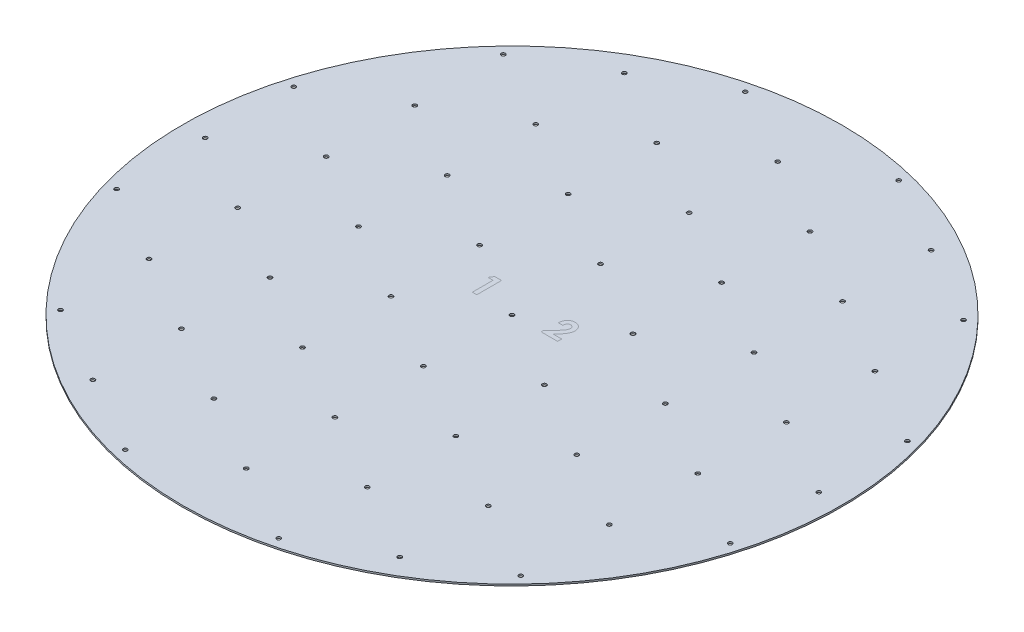
SolidWorks part; units mm, degrees
ref_plane "Front Plane" through (0, 0, 0) normal (0, 0, 1) x (1, 0, 0)
ref_plane "Top Plane" through (0, 0, 0) normal (0, 1, 0) x (1, 0, 0)
ref_plane "Right Plane" through (0, 0, 0) normal (1, 0, 0) x (0, 0, -1)
sketch "Sketch2" plane through (0, 0, 0) normal (0, 1, 0) x (1, 0, 0)
  circle A0 centre (0, 0) radius 40
  dimension "D1" = 80
extrude "Boss-Extrude1" add sketch "Sketch2" along normal blind 0.2
sketch "formula" plane through (0, 0.2, 0) normal (0, 1, 0) x (1, 0, 0)
  line L0 (0, 0) -> (0, 10.75) construction
  line L2 (46.374, 0) -> (0, 0) construction
  line L3 (9.3098, 5.375) -> (0, 0) construction
  line L4 (9.3098, 5.375) -> (0, 10.75) construction
  circle A16 centre (0, 10.75) radius 0.125
  circle A51 centre (9.3098, 16.125) radius 0.125
  circle A52 centre (0, 21.5) radius 0.125
  circle A53 centre (9.3098, 26.875) radius 0.125
  circle A54 centre (0, 32.25) radius 0.125
  circle A55 centre (9.3098, 37.625) radius 0.125
  circle A66 centre (0, 0) radius 0.125
  circle A67 centre (9.3098, 5.375) radius 0.125
  dimension "D2" = 0.25
  dimension "D3" = 10.75
sketch "Sketch4" plane through (0, 0.2, 0) normal (0, 1, 0) x (1, 0, 0)
  circle A1 centre (37.24, -10.75) radius 0.075
  circle A3 centre (18.62, -32.25) radius 0.075
  circle A5 centre (18.62, -10.75) radius 0.075
  circle A7 centre (27.9298, -16.125) radius 0.075
  circle A9 centre (18.62, -21.5) radius 0.075
  circle A11 centre (27.9298, -26.875) radius 0.075
  circle A13 centre (9.3098, -37.625) radius 0.075
  circle A15 centre (9.3098, -16.125) radius 0.075
  circle A17 centre (9.3098, -26.875) radius 0.075
  circle A19 centre (9.3098, -5.375) radius 0.075
  circle A21 centre (27.9298, -5.375) radius 0.075
  circle A23 centre (37.24, -10.75) radius 0.075
  circle A25 centre (18.62, -32.25) radius 0.075
  circle A27 centre (18.62, -10.75) radius 0.075
  circle A29 centre (27.9298, -16.125) radius 0.075
  circle A31 centre (18.62, -21.5) radius 0.075
  circle A33 centre (27.9298, -26.875) radius 0.075
  circle A35 centre (0, -32.25) radius 0.075
  circle A37 centre (9.3098, -37.625) radius 0.075
  circle A39 centre (0, -10.75) radius 0.075
  circle A41 centre (9.3098, -16.125) radius 0.075
  circle A43 centre (0, -21.5) radius 0.075
  circle A45 centre (9.3098, -26.875) radius 0.075
  circle A47 centre (9.3098, -5.375) radius 0.075
  circle A49 centre (27.9298, -5.375) radius 0.075
  circle A51 centre (-37.24, 10.75) radius 0.075
  circle A53 centre (-18.62, 32.25) radius 0.075
  circle A55 centre (-18.62, 10.75) radius 0.075
  circle A57 centre (-27.9298, 16.125) radius 0.075
  circle A59 centre (-18.62, 21.5) radius 0.075
  circle A61 centre (-27.9298, 26.875) radius 0.075
  circle A63 centre (-9.3098, 37.625) radius 0.075
  circle A65 centre (-9.3098, 16.125) radius 0.075
  circle A67 centre (-9.3098, 26.875) radius 0.075
  circle A69 centre (-9.3098, 5.375) radius 0.075
  circle A71 centre (-27.9298, 5.375) radius 0.075
  circle A73 centre (-37.24, 10.75) radius 0.075
  circle A75 centre (-37.24, 0) radius 0.075
  circle A77 centre (-18.62, 32.25) radius 0.075
  circle A79 centre (-18.62, 10.75) radius 0.075
  circle A81 centre (-27.9298, 16.125) radius 0.075
  circle A83 centre (-18.62, 21.5) radius 0.075
  circle A85 centre (-27.9298, 26.875) radius 0.075
  circle A87 centre (-18.62, 0) radius 0.075
  circle A89 centre (-9.3098, 37.625) radius 0.075
  circle A91 centre (-9.3098, 16.125) radius 0.075
  circle A93 centre (-9.3098, 26.875) radius 0.075
  circle A95 centre (-9.3098, 5.375) radius 0.075
  circle A97 centre (-27.9298, 5.375) radius 0.075
  circle A99 centre (-27.9298, -5.375) radius 0.075
  circle A101 centre (-9.3098, -5.375) radius 0.075
  circle A103 centre (-9.3098, -26.875) radius 0.075
  circle A105 centre (-9.3098, -16.125) radius 0.075
  circle A107 centre (-9.3098, -37.625) radius 0.075
  circle A109 centre (-27.9298, -26.875) radius 0.075
  circle A111 centre (-18.62, -21.5) radius 0.075
  circle A113 centre (-27.9298, -16.125) radius 0.075
  circle A115 centre (-18.62, -10.75) radius 0.075
  circle A117 centre (-18.62, -32.25) radius 0.075
  circle A119 centre (-37.24, -10.75) radius 0.075
  circle A121 centre (-27.9298, -5.375) radius 0.075
  circle A123 centre (-9.3098, -5.375) radius 0.075
  circle A125 centre (-9.3098, -26.875) radius 0.075
  circle A127 centre (-9.3098, -16.125) radius 0.075
  circle A129 centre (-9.3098, -37.625) radius 0.075
  circle A131 centre (-27.9298, -26.875) radius 0.075
  circle A133 centre (-18.62, -21.5) radius 0.075
  circle A135 centre (-27.9298, -16.125) radius 0.075
  circle A137 centre (-18.62, -10.75) radius 0.075
  circle A139 centre (-18.62, -32.25) radius 0.075
  circle A141 centre (-37.24, -10.75) radius 0.075
  circle A3000 centre (27.9298, 5.375) radius 0.25
  circle A3219 centre (9.3098, 5.375) radius 0.25
  circle A3220 centre (9.3098, 5.375) radius 0.25
  circle A3221 centre (0, 0) radius 0.25
  circle A3222 centre (0, 0) radius 0.25
  circle A3223 centre (9.3098, 26.875) radius 0.25
  circle A3224 centre (9.3098, 26.875) radius 0.25
  circle A3225 centre (0, 21.5) radius 0.25
  circle A3226 centre (0, 21.5) radius 0.25
  circle A3227 centre (9.3098, 16.125) radius 0.25
  circle A3228 centre (9.3098, 16.125) radius 0.25
  circle A3229 centre (0, 10.75) radius 0.25
  circle A3230 centre (0, 10.75) radius 0.25
  circle A3231 centre (9.3098, 37.625) radius 0.25
  circle A3232 centre (9.3098, 37.625) radius 0.25
  circle A3233 centre (0, 32.25) radius 0.25
  circle A3234 centre (0, 32.25) radius 0.25
  circle A3235 centre (18.62, 0) radius 0.25
  circle A3236 centre (27.9298, 26.875) radius 0.25
  circle A3237 centre (18.62, 21.5) radius 0.25
  circle A3238 centre (27.9298, 16.125) radius 0.25
  circle A3239 centre (18.62, 10.75) radius 0.25
  circle A3241 centre (18.62, 32.25) radius 0.25
  circle A3243 centre (37.24, 0) radius 0.25
  circle A3247 centre (37.24, 10.75) radius 0.25
  circle A3250 centre (27.9298, 37.625) radius 0.25
  circle A3251 centre (46.5498, 37.625) radius 0.25
  circle A3252 centre (37.24, 32.25) radius 0.25
  circle A3253 centre (46.5498, 26.875) radius 0.25
  circle A3254 centre (37.24, 21.5) radius 0.25
  circle A3255 centre (46.5498, 5.375) radius 0.25
  circle A3256 centre (46.5498, 16.125) radius 0.25
  circle A3271 centre (27.9298, 5.375) radius 0.075
  circle A3272 centre (9.3098, 5.375) radius 0.075
  circle A3273 centre (9.3098, 26.875) radius 0.075
  circle A3274 centre (9.3098, 16.125) radius 0.075
  circle A3275 centre (9.3098, 37.625) radius 0.075
  circle A3276 centre (27.9298, 26.875) radius 0.075
  circle A3277 centre (18.62, 21.5) radius 0.075
  circle A3278 centre (27.9298, 16.125) radius 0.075
  circle A3279 centre (18.62, 10.75) radius 0.075
  circle A3280 centre (18.62, 32.25) radius 0.075
  circle A3281 centre (37.24, 10.75) radius 0.075
  dimension "D121" = 0
  dimension "D122" = 0
  dimension "D123" = 0
  dimension "D124" = 0
  dimension "D125" = 0
  dimension "D126" = 0
  dimension "D127" = 0
  dimension "D128" = 0
  dimension "D129" = 3
extrude "Cut-Extrude2" cut sketch "Sketch4" against normal blind 0.2 contours A3222 | A3220 region at (0, 0.2, 0)
pattern_linear "LPattern1" count 4 spacing 10.75 along (0, 0, -1) count 3 spacing 18.6195 along (1, 0, 0) of "Cut-Extrude2"
mirror "Mirror1" about plane through (0, 0, 0) normal (1, 0, 0) of "LPattern1"
ref_plane "Plane1" through (0, 0, 0) normal (0, 0, -1) x (-1, 0, 0)
mirror "Mirror2" about plane through (0, 0, 0) normal (0, 0, -1) of "Mirror1", "LPattern1"
sketch "numbers" plane through (0, 0.2, 0) normal (0, 1, 0) x (1, 0, 0)
  line L0 (-7.0476, 0) -> (7.0476, 0) construction
  line L1 (46.374, 0) -> (0, 0) construction
  text T0 "<b>1      2</b>" font "Century Gothic" height 3
  point P6 (0, 0)
split "Split1" trim tools "numbers" bodies to split 160 resulting bodies 162 163 164
sketch "Sketch5" plane through (0, 0.2, 0) normal (0, 1, 0) x (1, 0, 0)
  circle A1 centre (40.7032, 13.5) radius 0.075
  circle A2 centre (40.7032, 13.5) radius 0.075
  circle A3 centre (39.8372, 15) radius 0.075
  circle A4 centre (39.8372, 15) radius 0.075
  circle A5 centre (39.8372, 14) radius 0.075
  circle A6 centre (39.8372, 14) radius 0.075
  circle A7 centre (40.7032, 14.5) radius 0.075
  circle A8 centre (40.7032, 14.5) radius 0.075
  circle A9 centre (39.8372, 10) radius 0.075
  circle A10 centre (39.8372, 10) radius 0.075
  circle A11 centre (39.8372, 11) radius 0.075
  circle A12 centre (39.8372, 11) radius 0.075
  circle A13 centre (39.8372, 10) radius 0.075
  circle A14 centre (39.8372, 10) radius 0.075
  circle A15 centre (40.7032, 10.5) radius 0.075
  circle A16 centre (40.7032, 10.5) radius 0.075
  circle A17 centre (38.9711, 8.5) radius 0.075
  circle A18 centre (38.9711, 8.5) radius 0.075
  circle A19 centre (38.1051, 9) radius 0.075
  circle A20 centre (38.1051, 9) radius 0.075
  circle A21 centre (38.9711, 9.5) radius 0.075
  circle A22 centre (38.9711, 9.5) radius 0.075
  circle A23 centre (38.1051, 5) radius 0.075
  circle A24 centre (38.1051, 5) radius 0.075
  circle A25 centre (38.1051, 6) radius 0.075
  circle A26 centre (38.1051, 6) radius 0.075
  circle A27 centre (38.1051, 5) radius 0.075
  circle A28 centre (38.1051, 5) radius 0.075
  circle A29 centre (38.9711, 5.5) radius 0.075
  circle A30 centre (38.9711, 5.5) radius 0.075
  circle A31 centre (38.1051, 7) radius 0.075
  circle A32 centre (38.1051, 7) radius 0.075
  circle A33 centre (36.3731, 4) radius 0.075
  circle A34 centre (36.3731, 4) radius 0.075
  circle A35 centre (37.2391, 4.5) radius 0.075
  circle A36 centre (37.2391, 4.5) radius 0.075
  circle A37 centre (36.3731, 0) radius 0.075
  circle A38 centre (36.3731, 0) radius 0.075
  circle A39 centre (37.2391, 0.5) radius 0.075
  circle A40 centre (37.2391, 0.5) radius 0.075
  circle A41 centre (36.3731, 1) radius 0.075
  circle A42 centre (36.3731, 1) radius 0.075
  circle A43 centre (36.3731, 2) radius 0.075
  circle A44 centre (36.3731, 2) radius 0.075
  circle A45 centre (36.3731, 1) radius 0.075
  circle A46 centre (36.3731, 1) radius 0.075
  circle A47 centre (37.2391, 1.5) radius 0.075
  circle A48 centre (37.2391, 1.5) radius 0.075
  circle A71 centre (31.1769, 29) radius 0.075
  circle A72 centre (31.1769, 29) radius 0.075
  circle A73 centre (32.0429, 28.5) radius 0.075
  circle A74 centre (32.0429, 28.5) radius 0.075
  circle A75 centre (31.1769, 30) radius 0.075
  circle A76 centre (31.1769, 30) radius 0.075
  circle A77 centre (31.1769, 29) radius 0.075
  circle A78 centre (31.1769, 29) radius 0.075
  circle A79 centre (32.0429, 29.5) radius 0.075
  circle A80 centre (32.0429, 29.5) radius 0.075
  circle A81 centre (30.3109, 27.5) radius 0.075
  circle A82 centre (30.3109, 27.5) radius 0.075
  circle A83 centre (29.4449, 28) radius 0.075
  circle A84 centre (29.4449, 28) radius 0.075
  circle A85 centre (29.4449, 24) radius 0.075
  circle A86 centre (29.4449, 24) radius 0.075
  circle A87 centre (29.4449, 23) radius 0.075
  circle A88 centre (29.4449, 23) radius 0.075
  circle A89 centre (30.3109, 23.5) radius 0.075
  circle A90 centre (30.3109, 23.5) radius 0.075
  circle A91 centre (29.4449, 25) radius 0.075
  circle A92 centre (29.4449, 25) radius 0.075
  circle A93 centre (29.4449, 24) radius 0.075
  circle A94 centre (29.4449, 24) radius 0.075
  circle A95 centre (30.3109, 24.5) radius 0.075
  circle A96 centre (30.3109, 24.5) radius 0.075
  circle A97 centre (27.7128, 23) radius 0.075
  circle A98 centre (27.7128, 23) radius 0.075
  circle A99 centre (27.7128, 22) radius 0.075
  circle A100 centre (27.7128, 22) radius 0.075
  circle A101 centre (28.5788, 22.5) radius 0.075
  circle A102 centre (28.5788, 22.5) radius 0.075
  circle A103 centre (27.7128, 19) radius 0.075
  circle A104 centre (27.7128, 19) radius 0.075
  circle A105 centre (27.7128, 18) radius 0.075
  circle A106 centre (27.7128, 18) radius 0.075
  circle A107 centre (28.5788, 18.5) radius 0.075
  circle A108 centre (28.5788, 18.5) radius 0.075
  circle A109 centre (27.7128, 20) radius 0.075
  circle A110 centre (27.7128, 20) radius 0.075
  circle A111 centre (27.7128, 19) radius 0.075
  circle A112 centre (27.7128, 19) radius 0.075
  circle A113 centre (25.9808, 17) radius 0.075
  circle A114 centre (25.9808, 17) radius 0.075
  circle A115 centre (25.9808, 16) radius 0.075
  circle A116 centre (25.9808, 16) radius 0.075
  circle A117 centre (26.8468, 16.5) radius 0.075
  circle A118 centre (26.8468, 16.5) radius 0.075
  circle A119 centre (25.9808, 13) radius 0.075
  circle A120 centre (25.9808, 13) radius 0.075
  circle A121 centre (25.9808, 12) radius 0.075
  circle A122 centre (25.9808, 12) radius 0.075
  circle A123 centre (26.8468, 12.5) radius 0.075
  circle A124 centre (26.8468, 12.5) radius 0.075
  circle A125 centre (25.9808, 14) radius 0.075
  circle A126 centre (25.9808, 14) radius 0.075
  circle A127 centre (25.9808, 13) radius 0.075
  circle A128 centre (25.9808, 13) radius 0.075
  circle A129 centre (24.2487, 12) radius 0.075
  circle A130 centre (24.2487, 12) radius 0.075
  circle A131 centre (24.2487, 11) radius 0.075
  circle A132 centre (24.2487, 11) radius 0.075
  circle A133 centre (25.1147, 11.5) radius 0.075
  circle A134 centre (25.1147, 11.5) radius 0.075
  circle A135 centre (24.2487, 8) radius 0.075
  circle A136 centre (24.2487, 8) radius 0.075
  circle A137 centre (24.2487, 7) radius 0.075
  circle A138 centre (24.2487, 7) radius 0.075
  circle A139 centre (25.1147, 7.5) radius 0.075
  circle A140 centre (25.1147, 7.5) radius 0.075
  circle A141 centre (24.2487, 9) radius 0.075
  circle A142 centre (24.2487, 9) radius 0.075
  circle A143 centre (24.2487, 8) radius 0.075
  circle A144 centre (24.2487, 8) radius 0.075
  circle A145 centre (22.5167, 6) radius 0.075
  circle A146 centre (22.5167, 6) radius 0.075
  circle A147 centre (23.3827, 6.5) radius 0.075
  circle A148 centre (23.3827, 6.5) radius 0.075
  circle A149 centre (22.5167, 3) radius 0.075
  circle A150 centre (22.5167, 3) radius 0.075
  circle A151 centre (22.5167, 2) radius 0.075
  circle A152 centre (22.5167, 2) radius 0.075
  circle A153 centre (23.3827, 2.5) radius 0.075
  circle A154 centre (23.3827, 2.5) radius 0.075
  circle A155 centre (22.5167, 4) radius 0.075
  circle A156 centre (22.5167, 4) radius 0.075
  circle A157 centre (22.5167, 3) radius 0.075
  circle A158 centre (22.5167, 3) radius 0.075
  circle A159 centre (23.3827, 3.5) radius 0.075
  circle A160 centre (23.3827, 3.5) radius 0.075
  circle A177 centre (18.1865, 35.5) radius 0.075
  circle A178 centre (18.1865, 35.5) radius 0.075
  circle A179 centre (17.3205, 36) radius 0.075
  circle A180 centre (17.3205, 36) radius 0.075
  circle A181 centre (17.3205, 32) radius 0.075
  circle A182 centre (17.3205, 32) radius 0.075
  circle A183 centre (17.3205, 31) radius 0.075
  circle A184 centre (17.3205, 31) radius 0.075
  circle A185 centre (18.1865, 31.5) radius 0.075
  circle A186 centre (18.1865, 31.5) radius 0.075
  circle A187 centre (17.3205, 33) radius 0.075
  circle A188 centre (17.3205, 33) radius 0.075
  circle A189 centre (17.3205, 32) radius 0.075
  circle A190 centre (17.3205, 32) radius 0.075
  circle A191 centre (18.1865, 32.5) radius 0.075
  circle A192 centre (18.1865, 32.5) radius 0.075
  circle A193 centre (15.5885, 31) radius 0.075
  circle A194 centre (15.5885, 31) radius 0.075
  circle A195 centre (15.5885, 30) radius 0.075
  circle A196 centre (15.5885, 30) radius 0.075
  circle A197 centre (16.4545, 30.5) radius 0.075
  circle A198 centre (16.4545, 30.5) radius 0.075
  circle A199 centre (15.5885, 27) radius 0.075
  circle A200 centre (15.5885, 27) radius 0.075
  circle A201 centre (15.5885, 26) radius 0.075
  circle A202 centre (15.5885, 26) radius 0.075
  circle A203 centre (16.4545, 26.5) radius 0.075
  circle A204 centre (16.4545, 26.5) radius 0.075
  circle A205 centre (15.5885, 28) radius 0.075
  circle A206 centre (15.5885, 28) radius 0.075
  circle A207 centre (15.5885, 27) radius 0.075
  circle A208 centre (15.5885, 27) radius 0.075
  circle A209 centre (13.8564, 26) radius 0.075
  circle A210 centre (13.8564, 26) radius 0.075
  circle A211 centre (13.8564, 25) radius 0.075
  circle A212 centre (13.8564, 25) radius 0.075
  circle A213 centre (14.7224, 25.5) radius 0.075
  circle A214 centre (14.7224, 25.5) radius 0.075
  circle A215 centre (13.8564, 21) radius 0.075
  circle A216 centre (13.8564, 21) radius 0.075
  circle A217 centre (14.7224, 20.5) radius 0.075
  circle A218 centre (14.7224, 20.5) radius 0.075
  circle A219 centre (13.8564, 22) radius 0.075
  circle A220 centre (13.8564, 22) radius 0.075
  circle A221 centre (13.8564, 21) radius 0.075
  circle A222 centre (13.8564, 21) radius 0.075
  circle A223 centre (14.7224, 21.5) radius 0.075
  circle A224 centre (14.7224, 21.5) radius 0.075
  circle A225 centre (12.9904, 19.5) radius 0.075
  circle A226 centre (12.9904, 19.5) radius 0.075
  circle A227 centre (12.1244, 20) radius 0.075
  circle A228 centre (12.1244, 20) radius 0.075
  circle A229 centre (12.1244, 18) radius 0.075
  circle A230 centre (12.1244, 18) radius 0.075
  circle A231 centre (12.1244, 17) radius 0.075
  circle A232 centre (12.1244, 17) radius 0.075
  circle A233 centre (12.9904, 17.5) radius 0.075
  circle A234 centre (12.9904, 17.5) radius 0.075
  circle A235 centre (12.1244, 16) radius 0.075
  circle A236 centre (12.1244, 16) radius 0.075
  circle A237 centre (12.1244, 15) radius 0.075
  circle A238 centre (12.1244, 15) radius 0.075
  circle A239 centre (12.9904, 15.5) radius 0.075
  circle A240 centre (12.9904, 15.5) radius 0.075
  circle A241 centre (11.2583, 13.5) radius 0.075
  circle A242 centre (11.2583, 13.5) radius 0.075
  circle A243 centre (10.3923, 15) radius 0.075
  circle A244 centre (10.3923, 15) radius 0.075
  circle A245 centre (10.3923, 14) radius 0.075
  circle A246 centre (10.3923, 14) radius 0.075
  circle A247 centre (11.2583, 14.5) radius 0.075
  circle A248 centre (11.2583, 14.5) radius 0.075
  circle A249 centre (10.3923, 10) radius 0.075
  circle A250 centre (10.3923, 10) radius 0.075
  circle A251 centre (10.3923, 11) radius 0.075
  circle A252 centre (10.3923, 11) radius 0.075
  circle A253 centre (10.3923, 10) radius 0.075
  circle A254 centre (10.3923, 10) radius 0.075
  circle A255 centre (11.2583, 10.5) radius 0.075
  circle A256 centre (11.2583, 10.5) radius 0.075
  circle A257 centre (9.5263, 8.5) radius 0.075
  circle A258 centre (9.5263, 8.5) radius 0.075
  circle A259 centre (8.6603, 9) radius 0.075
  circle A260 centre (8.6603, 9) radius 0.075
  circle A261 centre (9.5263, 9.5) radius 0.075
  circle A262 centre (9.5263, 9.5) radius 0.075
  circle A263 centre (8.6603, 5) radius 0.075
  circle A264 centre (8.6603, 5) radius 0.075
  circle A265 centre (8.6603, 6) radius 0.075
  circle A266 centre (8.6603, 6) radius 0.075
  circle A267 centre (8.6603, 5) radius 0.075
  circle A268 centre (8.6603, 5) radius 0.075
  circle A269 centre (9.5263, 5.5) radius 0.075
  circle A270 centre (9.5263, 5.5) radius 0.075
  circle A271 centre (8.6603, 7) radius 0.075
  circle A272 centre (8.6603, 7) radius 0.075
  circle A273 centre (6.9282, 4) radius 0.075
  circle A274 centre (6.9282, 4) radius 0.075
  circle A275 centre (7.7942, 4.5) radius 0.075
  circle A276 centre (7.7942, 4.5) radius 0.075
  circle A277 centre (6.9282, 0) radius 0.075
  circle A278 centre (6.9282, 0) radius 0.075
  circle A279 centre (7.7942, 0.5) radius 0.075
  circle A280 centre (7.7942, 0.5) radius 0.075
  circle A281 centre (6.9282, 1) radius 0.075
  circle A282 centre (6.9282, 1) radius 0.075
  circle A283 centre (6.9282, 2) radius 0.075
  circle A284 centre (6.9282, 2) radius 0.075
  circle A285 centre (6.9282, 1) radius 0.075
  circle A286 centre (6.9282, 1) radius 0.075
  circle A287 centre (7.7942, 1.5) radius 0.075
  circle A288 centre (7.7942, 1.5) radius 0.075
  circle A289 centre (3.4641, 39) radius 0.075
  circle A290 centre (3.4641, 39) radius 0.075
  circle A291 centre (3.4641, 38) radius 0.075
  circle A292 centre (3.4641, 38) radius 0.075
  circle A293 centre (4.3301, 38.5) radius 0.075
  circle A294 centre (4.3301, 38.5) radius 0.075
  circle A295 centre (3.4641, 35) radius 0.075
  circle A296 centre (3.4641, 35) radius 0.075
  circle A297 centre (3.4641, 34) radius 0.075
  circle A298 centre (3.4641, 34) radius 0.075
  circle A299 centre (4.3301, 34.5) radius 0.075
  circle A300 centre (4.3301, 34.5) radius 0.075
  circle A301 centre (3.4641, 36) radius 0.075
  circle A302 centre (3.4641, 36) radius 0.075
  circle A303 centre (3.4641, 35) radius 0.075
  circle A304 centre (3.4641, 35) radius 0.075
  circle A305 centre (1.7321, 34) radius 0.075
  circle A306 centre (1.7321, 34) radius 0.075
  circle A307 centre (1.7321, 33) radius 0.075
  circle A308 centre (1.7321, 33) radius 0.075
  circle A309 centre (2.5981, 33.5) radius 0.075
  circle A310 centre (2.5981, 33.5) radius 0.075
  circle A311 centre (1.7321, 29) radius 0.075
  circle A312 centre (1.7321, 29) radius 0.075
  circle A313 centre (2.5981, 28.5) radius 0.075
  circle A314 centre (2.5981, 28.5) radius 0.075
  circle A315 centre (1.7321, 30) radius 0.075
  circle A316 centre (1.7321, 30) radius 0.075
  circle A317 centre (1.7321, 29) radius 0.075
  circle A318 centre (1.7321, 29) radius 0.075
  circle A319 centre (2.5981, 29.5) radius 0.075
  circle A320 centre (2.5981, 29.5) radius 0.075
  circle A321 centre (0.866, 28.5) radius 0.075
  circle A322 centre (0.866, 28.5) radius 0.075
  circle A323 centre (0, 30) radius 0.075
  circle A324 centre (0, 30) radius 0.075
  circle A325 centre (0, 29) radius 0.075
  circle A326 centre (0, 29) radius 0.075
  circle A327 centre (0.866, 29.5) radius 0.075
  circle A328 centre (0.866, 29.5) radius 0.075
  circle A329 centre (0, 31) radius 0.075
  circle A330 centre (0, 31) radius 0.075
  circle A331 centre (0.866, 1.5) radius 0.075
  circle A332 centre (0.866, 1.5) radius 0.075
  circle A335 centre (0, 39) radius 0.075
  circle A336 centre (0, 39) radius 0.075
  circle A337 centre (0.866, 39.5) radius 0.075
  circle A338 centre (0.866, 39.5) radius 0.075
  circle A339 centre (39.8372, 17) radius 0.075
  circle A340 centre (39.8372, 17) radius 0.075
  circle A341 centre (39.8372, 16) radius 0.075
  circle A342 centre (39.8372, 16) radius 0.075
  circle A343 centre (40.7032, 16.5) radius 0.075
  circle A344 centre (40.7032, 16.5) radius 0.075
  circle A345 centre (39.8372, 13) radius 0.075
  circle A346 centre (39.8372, 13) radius 0.075
  circle A347 centre (39.8372, 12) radius 0.075
  circle A348 centre (39.8372, 12) radius 0.075
  circle A349 centre (40.7032, 12.5) radius 0.075
  circle A350 centre (40.7032, 12.5) radius 0.075
  circle A351 centre (39.8372, 14) radius 0.075
  circle A352 centre (39.8372, 14) radius 0.075
  circle A353 centre (39.8372, 13) radius 0.075
  circle A354 centre (39.8372, 13) radius 0.075
  circle A355 centre (38.1051, 12) radius 0.075
  circle A356 centre (38.1051, 12) radius 0.075
  circle A357 centre (38.1051, 11) radius 0.075
  circle A358 centre (38.1051, 11) radius 0.075
  circle A359 centre (38.9711, 11.5) radius 0.075
  circle A360 centre (38.9711, 11.5) radius 0.075
  circle A361 centre (38.1051, 8) radius 0.075
  circle A362 centre (38.1051, 8) radius 0.075
  circle A363 centre (38.1051, 7) radius 0.075
  circle A364 centre (38.1051, 7) radius 0.075
  circle A365 centre (38.9711, 7.5) radius 0.075
  circle A366 centre (38.9711, 7.5) radius 0.075
  circle A367 centre (38.1051, 9) radius 0.075
  circle A368 centre (38.1051, 9) radius 0.075
  circle A369 centre (38.1051, 8) radius 0.075
  circle A370 centre (38.1051, 8) radius 0.075
  circle A371 centre (36.3731, 6) radius 0.075
  circle A372 centre (36.3731, 6) radius 0.075
  circle A373 centre (37.2391, 6.5) radius 0.075
  circle A374 centre (37.2391, 6.5) radius 0.075
  circle A375 centre (36.3731, 3) radius 0.075
  circle A376 centre (36.3731, 3) radius 0.075
  circle A377 centre (36.3731, 2) radius 0.075
  circle A378 centre (36.3731, 2) radius 0.075
  circle A379 centre (37.2391, 2.5) radius 0.075
  circle A380 centre (37.2391, 2.5) radius 0.075
  circle A381 centre (36.3731, 4) radius 0.075
  circle A382 centre (36.3731, 4) radius 0.075
  circle A383 centre (36.3731, 3) radius 0.075
  circle A384 centre (36.3731, 3) radius 0.075
  circle A385 centre (37.2391, 3.5) radius 0.075
  circle A386 centre (37.2391, 3.5) radius 0.075
  circle A407 centre (31.1769, 32) radius 0.075
  circle A408 centre (31.1769, 32) radius 0.075
  circle A409 centre (31.1769, 31) radius 0.075
  circle A410 centre (31.1769, 31) radius 0.075
  circle A411 centre (32.0429, 31.5) radius 0.075
  circle A412 centre (32.0429, 31.5) radius 0.075
  circle A415 centre (31.1769, 32) radius 0.075
  circle A416 centre (31.1769, 32) radius 0.075
  circle A417 centre (32.0429, 32.5) radius 0.075
  circle A418 centre (32.0429, 32.5) radius 0.075
  circle A419 centre (29.4449, 31) radius 0.075
  circle A420 centre (29.4449, 31) radius 0.075
  circle A421 centre (29.4449, 30) radius 0.075
  circle A422 centre (29.4449, 30) radius 0.075
  circle A423 centre (30.3109, 30.5) radius 0.075
  circle A424 centre (30.3109, 30.5) radius 0.075
  circle A425 centre (29.4449, 27) radius 0.075
  circle A426 centre (29.4449, 27) radius 0.075
  circle A427 centre (29.4449, 26) radius 0.075
  circle A428 centre (29.4449, 26) radius 0.075
  circle A429 centre (30.3109, 26.5) radius 0.075
  circle A430 centre (30.3109, 26.5) radius 0.075
  circle A431 centre (29.4449, 28) radius 0.075
  circle A432 centre (29.4449, 28) radius 0.075
  circle A433 centre (29.4449, 27) radius 0.075
  circle A434 centre (29.4449, 27) radius 0.075
  circle A435 centre (27.7128, 26) radius 0.075
  circle A436 centre (27.7128, 26) radius 0.075
  circle A437 centre (27.7128, 25) radius 0.075
  circle A438 centre (27.7128, 25) radius 0.075
  circle A439 centre (28.5788, 25.5) radius 0.075
  circle A440 centre (28.5788, 25.5) radius 0.075
  circle A441 centre (27.7128, 21) radius 0.075
  circle A442 centre (27.7128, 21) radius 0.075
  circle A443 centre (28.5788, 20.5) radius 0.075
  circle A444 centre (28.5788, 20.5) radius 0.075
  circle A445 centre (27.7128, 22) radius 0.075
  circle A446 centre (27.7128, 22) radius 0.075
  circle A447 centre (27.7128, 21) radius 0.075
  circle A448 centre (27.7128, 21) radius 0.075
  circle A449 centre (28.5788, 21.5) radius 0.075
  circle A450 centre (28.5788, 21.5) radius 0.075
  circle A451 centre (26.8468, 19.5) radius 0.075
  circle A452 centre (26.8468, 19.5) radius 0.075
  circle A453 centre (25.9808, 20) radius 0.075
  circle A454 centre (25.9808, 20) radius 0.075
  circle A455 centre (25.9808, 18) radius 0.075
  circle A456 centre (25.9808, 18) radius 0.075
  circle A457 centre (25.9808, 17) radius 0.075
  circle A458 centre (25.9808, 17) radius 0.075
  circle A459 centre (26.8468, 17.5) radius 0.075
  circle A460 centre (26.8468, 17.5) radius 0.075
  circle A461 centre (25.9808, 16) radius 0.075
  circle A462 centre (25.9808, 16) radius 0.075
  circle A463 centre (25.9808, 15) radius 0.075
  circle A464 centre (25.9808, 15) radius 0.075
  circle A465 centre (26.8468, 15.5) radius 0.075
  circle A466 centre (26.8468, 15.5) radius 0.075
  circle A467 centre (25.1147, 13.5) radius 0.075
  circle A468 centre (25.1147, 13.5) radius 0.075
  circle A469 centre (24.2487, 15) radius 0.075
  circle A470 centre (24.2487, 15) radius 0.075
  circle A471 centre (24.2487, 14) radius 0.075
  circle A472 centre (24.2487, 14) radius 0.075
  circle A473 centre (25.1147, 14.5) radius 0.075
  circle A474 centre (25.1147, 14.5) radius 0.075
  circle A475 centre (24.2487, 10) radius 0.075
  circle A476 centre (24.2487, 10) radius 0.075
  circle A477 centre (24.2487, 11) radius 0.075
  circle A478 centre (24.2487, 11) radius 0.075
  circle A479 centre (24.2487, 10) radius 0.075
  circle A480 centre (24.2487, 10) radius 0.075
  circle A481 centre (25.1147, 10.5) radius 0.075
  circle A482 centre (25.1147, 10.5) radius 0.075
  circle A483 centre (23.3827, 8.5) radius 0.075
  circle A484 centre (23.3827, 8.5) radius 0.075
  circle A485 centre (22.5167, 9) radius 0.075
  circle A486 centre (22.5167, 9) radius 0.075
  circle A487 centre (23.3827, 9.5) radius 0.075
  circle A488 centre (23.3827, 9.5) radius 0.075
  circle A489 centre (22.5167, 5) radius 0.075
  circle A490 centre (22.5167, 5) radius 0.075
  circle A491 centre (22.5167, 6) radius 0.075
  circle A492 centre (22.5167, 6) radius 0.075
  circle A493 centre (22.5167, 5) radius 0.075
  circle A494 centre (22.5167, 5) radius 0.075
  circle A495 centre (23.3827, 5.5) radius 0.075
  circle A496 centre (23.3827, 5.5) radius 0.075
  circle A497 centre (22.5167, 7) radius 0.075
  circle A498 centre (22.5167, 7) radius 0.075
  circle A499 centre (20.7846, 4) radius 0.075
  circle A500 centre (20.7846, 4) radius 0.075
  circle A501 centre (21.6506, 4.5) radius 0.075
  circle A502 centre (21.6506, 4.5) radius 0.075
  circle A503 centre (20.7846, 0) radius 0.075
  circle A504 centre (20.7846, 0) radius 0.075
  circle A505 centre (21.6506, 0.5) radius 0.075
  circle A506 centre (21.6506, 0.5) radius 0.075
  circle A507 centre (20.7846, 1) radius 0.075
  circle A508 centre (20.7846, 1) radius 0.075
  circle A509 centre (20.7846, 2) radius 0.075
  circle A510 centre (20.7846, 2) radius 0.075
  circle A511 centre (20.7846, 1) radius 0.075
  circle A512 centre (20.7846, 1) radius 0.075
  circle A513 centre (21.6506, 1.5) radius 0.075
  circle A514 centre (21.6506, 1.5) radius 0.075
  circle A515 centre (17.3205, 39) radius 0.075
  circle A516 centre (17.3205, 39) radius 0.075
  circle A517 centre (17.3205, 38) radius 0.075
  circle A518 centre (17.3205, 38) radius 0.075
  circle A521 centre (17.3205, 35) radius 0.075
  circle A522 centre (17.3205, 35) radius 0.075
  circle A523 centre (17.3205, 34) radius 0.075
  circle A524 centre (17.3205, 34) radius 0.075
  circle A525 centre (18.1865, 34.5) radius 0.075
  circle A526 centre (18.1865, 34.5) radius 0.075
  circle A527 centre (17.3205, 36) radius 0.075
  circle A528 centre (17.3205, 36) radius 0.075
  circle A529 centre (17.3205, 35) radius 0.075
  circle A530 centre (17.3205, 35) radius 0.075
  circle A531 centre (15.5885, 34) radius 0.075
  circle A532 centre (15.5885, 34) radius 0.075
  circle A533 centre (15.5885, 33) radius 0.075
  circle A534 centre (15.5885, 33) radius 0.075
  circle A535 centre (16.4545, 33.5) radius 0.075
  circle A536 centre (16.4545, 33.5) radius 0.075
  circle A537 centre (15.5885, 29) radius 0.075
  circle A538 centre (15.5885, 29) radius 0.075
  circle A539 centre (16.4545, 28.5) radius 0.075
  circle A540 centre (16.4545, 28.5) radius 0.075
  circle A541 centre (15.5885, 30) radius 0.075
  circle A542 centre (15.5885, 30) radius 0.075
  circle A543 centre (15.5885, 29) radius 0.075
  circle A544 centre (15.5885, 29) radius 0.075
  circle A545 centre (16.4545, 29.5) radius 0.075
  circle A546 centre (16.4545, 29.5) radius 0.075
  circle A547 centre (14.7224, 27.5) radius 0.075
  circle A548 centre (14.7224, 27.5) radius 0.075
  circle A549 centre (13.8564, 28) radius 0.075
  circle A550 centre (13.8564, 28) radius 0.075
  circle A551 centre (13.8564, 24) radius 0.075
  circle A552 centre (13.8564, 24) radius 0.075
  circle A553 centre (13.8564, 23) radius 0.075
  circle A554 centre (13.8564, 23) radius 0.075
  circle A555 centre (14.7224, 23.5) radius 0.075
  circle A556 centre (14.7224, 23.5) radius 0.075
  circle A557 centre (13.8564, 25) radius 0.075
  circle A558 centre (13.8564, 25) radius 0.075
  circle A559 centre (13.8564, 24) radius 0.075
  circle A560 centre (13.8564, 24) radius 0.075
  circle A561 centre (14.7224, 24.5) radius 0.075
  circle A562 centre (14.7224, 24.5) radius 0.075
  circle A563 centre (12.1244, 23) radius 0.075
  circle A564 centre (12.1244, 23) radius 0.075
  circle A565 centre (12.1244, 22) radius 0.075
  circle A566 centre (12.1244, 22) radius 0.075
  circle A567 centre (12.9904, 22.5) radius 0.075
  circle A568 centre (12.9904, 22.5) radius 0.075
  circle A569 centre (12.1244, 19) radius 0.075
  circle A570 centre (12.1244, 19) radius 0.075
  circle A571 centre (12.1244, 18) radius 0.075
  circle A572 centre (12.1244, 18) radius 0.075
  circle A573 centre (12.9904, 18.5) radius 0.075
  circle A574 centre (12.9904, 18.5) radius 0.075
  circle A575 centre (12.1244, 20) radius 0.075
  circle A576 centre (12.1244, 20) radius 0.075
  circle A577 centre (12.1244, 19) radius 0.075
  circle A578 centre (12.1244, 19) radius 0.075
  circle A579 centre (10.3923, 17) radius 0.075
  circle A580 centre (10.3923, 17) radius 0.075
  circle A581 centre (10.3923, 16) radius 0.075
  circle A582 centre (10.3923, 16) radius 0.075
  circle A583 centre (11.2583, 16.5) radius 0.075
  circle A584 centre (11.2583, 16.5) radius 0.075
  circle A585 centre (10.3923, 13) radius 0.075
  circle A586 centre (10.3923, 13) radius 0.075
  circle A587 centre (10.3923, 12) radius 0.075
  circle A588 centre (10.3923, 12) radius 0.075
  circle A589 centre (11.2583, 12.5) radius 0.075
  circle A590 centre (11.2583, 12.5) radius 0.075
  circle A591 centre (10.3923, 14) radius 0.075
  circle A592 centre (10.3923, 14) radius 0.075
  circle A593 centre (10.3923, 13) radius 0.075
  circle A594 centre (10.3923, 13) radius 0.075
  circle A595 centre (8.6603, 12) radius 0.075
  circle A596 centre (8.6603, 12) radius 0.075
  circle A597 centre (8.6603, 11) radius 0.075
  circle A598 centre (8.6603, 11) radius 0.075
  circle A599 centre (9.5263, 11.5) radius 0.075
  circle A600 centre (9.5263, 11.5) radius 0.075
  circle A601 centre (8.6603, 8) radius 0.075
  circle A602 centre (8.6603, 8) radius 0.075
  circle A603 centre (8.6603, 7) radius 0.075
  circle A604 centre (8.6603, 7) radius 0.075
  circle A605 centre (9.5263, 7.5) radius 0.075
  circle A606 centre (9.5263, 7.5) radius 0.075
  circle A607 centre (8.6603, 9) radius 0.075
  circle A608 centre (8.6603, 9) radius 0.075
  circle A609 centre (8.6603, 8) radius 0.075
  circle A610 centre (8.6603, 8) radius 0.075
  circle A611 centre (6.9282, 6) radius 0.075
  circle A612 centre (6.9282, 6) radius 0.075
  circle A613 centre (7.7942, 6.5) radius 0.075
  circle A614 centre (7.7942, 6.5) radius 0.075
  circle A615 centre (6.9282, 3) radius 0.075
  circle A616 centre (6.9282, 3) radius 0.075
  circle A617 centre (6.9282, 2) radius 0.075
  circle A618 centre (6.9282, 2) radius 0.075
  circle A619 centre (7.7942, 2.5) radius 0.075
  circle A620 centre (7.7942, 2.5) radius 0.075
  circle A621 centre (6.9282, 4) radius 0.075
  circle A622 centre (6.9282, 4) radius 0.075
  circle A623 centre (6.9282, 3) radius 0.075
  circle A624 centre (6.9282, 3) radius 0.075
  circle A625 centre (7.7942, 3.5) radius 0.075
  circle A626 centre (7.7942, 3.5) radius 0.075
  circle A629 centre (5.1962, 39) radius 0.075
  circle A630 centre (5.1962, 39) radius 0.075
  circle A633 centre (3.4641, 37) radius 0.075
  circle A634 centre (3.4641, 37) radius 0.075
  circle A635 centre (4.3301, 36.5) radius 0.075
  circle A636 centre (4.3301, 36.5) radius 0.075
  circle A637 centre (3.4641, 38) radius 0.075
  circle A638 centre (3.4641, 38) radius 0.075
  circle A639 centre (3.4641, 37) radius 0.075
  circle A640 centre (3.4641, 37) radius 0.075
  circle A641 centre (4.3301, 37.5) radius 0.075
  circle A642 centre (4.3301, 37.5) radius 0.075
  circle A643 centre (2.5981, 35.5) radius 0.075
  circle A644 centre (2.5981, 35.5) radius 0.075
  circle A645 centre (1.7321, 36) radius 0.075
  circle A646 centre (1.7321, 36) radius 0.075
  circle A647 centre (1.7321, 32) radius 0.075
  circle A648 centre (1.7321, 32) radius 0.075
  circle A649 centre (1.7321, 31) radius 0.075
  circle A650 centre (1.7321, 31) radius 0.075
  circle A651 centre (2.5981, 31.5) radius 0.075
  circle A652 centre (2.5981, 31.5) radius 0.075
  circle A653 centre (1.7321, 33) radius 0.075
  circle A654 centre (1.7321, 33) radius 0.075
  circle A655 centre (1.7321, 32) radius 0.075
  circle A656 centre (1.7321, 32) radius 0.075
  circle A657 centre (2.5981, 32.5) radius 0.075
  circle A658 centre (2.5981, 32.5) radius 0.075
  circle A659 centre (0.866, 32.5) radius 0.075
  circle A660 centre (0.866, 32.5) radius 0.075
  circle A661 centre (0, 34) radius 0.075
  circle A662 centre (0, 34) radius 0.075
  circle A663 centre (0, 33) radius 0.075
  circle A664 centre (0, 33) radius 0.075
  circle A665 centre (0.866, 33.5) radius 0.075
  circle A666 centre (0.866, 33.5) radius 0.075
  circle A667 centre (0, 29) radius 0.075
  circle A668 centre (0, 29) radius 0.075
  circle A669 centre (0.866, 4.5) radius 0.075
  circle A670 centre (0.866, 4.5) radius 0.075
  circle A671 centre (0, 0) radius 0.075
  circle A672 centre (0, 0) radius 0.075
  circle A673 centre (0.866, 0.5) radius 0.075
  circle A674 centre (0.866, 0.5) radius 0.075
  circle A675 centre (0, 1) radius 0.075
  circle A676 centre (0, 1) radius 0.075
  circle A677 centre (0, 2) radius 0.075
  circle A678 centre (0, 2) radius 0.075
  circle A679 centre (0, 1) radius 0.075
  circle A680 centre (0, 1) radius 0.075
  circle A681 centre (40.7032, 19.5) radius 0.075
  circle A682 centre (40.7032, 19.5) radius 0.075
  circle A683 centre (39.8372, 20) radius 0.075
  circle A684 centre (39.8372, 20) radius 0.075
  circle A685 centre (39.8372, 18) radius 0.075
  circle A686 centre (39.8372, 18) radius 0.075
  circle A687 centre (39.8372, 17) radius 0.075
  circle A688 centre (39.8372, 17) radius 0.075
  circle A689 centre (40.7032, 17.5) radius 0.075
  circle A690 centre (40.7032, 17.5) radius 0.075
  circle A691 centre (39.8372, 16) radius 0.075
  circle A692 centre (39.8372, 16) radius 0.075
  circle A693 centre (39.8372, 15) radius 0.075
  circle A694 centre (39.8372, 15) radius 0.075
  circle A695 centre (40.7032, 15.5) radius 0.075
  circle A696 centre (40.7032, 15.5) radius 0.075
  circle A697 centre (38.9711, 13.5) radius 0.075
  circle A698 centre (38.9711, 13.5) radius 0.075
  circle A699 centre (38.1051, 15) radius 0.075
  circle A700 centre (38.1051, 15) radius 0.075
  circle A701 centre (38.1051, 14) radius 0.075
  circle A702 centre (38.1051, 14) radius 0.075
  circle A703 centre (38.9711, 14.5) radius 0.075
  circle A704 centre (38.9711, 14.5) radius 0.075
  circle A705 centre (38.1051, 10) radius 0.075
  circle A706 centre (38.1051, 10) radius 0.075
  circle A707 centre (38.1051, 11) radius 0.075
  circle A708 centre (38.1051, 11) radius 0.075
  circle A709 centre (38.1051, 10) radius 0.075
  circle A710 centre (38.1051, 10) radius 0.075
  circle A711 centre (38.9711, 10.5) radius 0.075
  circle A712 centre (38.9711, 10.5) radius 0.075
  circle A713 centre (37.2391, 8.5) radius 0.075
  circle A714 centre (37.2391, 8.5) radius 0.075
  circle A715 centre (36.3731, 9) radius 0.075
  circle A716 centre (36.3731, 9) radius 0.075
  circle A717 centre (37.2391, 9.5) radius 0.075
  circle A718 centre (37.2391, 9.5) radius 0.075
  circle A719 centre (36.3731, 5) radius 0.075
  circle A720 centre (36.3731, 5) radius 0.075
  circle A721 centre (36.3731, 6) radius 0.075
  circle A722 centre (36.3731, 6) radius 0.075
  circle A723 centre (36.3731, 5) radius 0.075
  circle A724 centre (36.3731, 5) radius 0.075
  circle A725 centre (37.2391, 5.5) radius 0.075
  circle A726 centre (37.2391, 5.5) radius 0.075
  circle A727 centre (36.3731, 7) radius 0.075
  circle A728 centre (36.3731, 7) radius 0.075
  circle A729 centre (34.641, 4) radius 0.075
  circle A730 centre (34.641, 4) radius 0.075
  circle A731 centre (35.507, 4.5) radius 0.075
  circle A732 centre (35.507, 4.5) radius 0.075
  circle A733 centre (34.641, 0) radius 0.075
  circle A734 centre (34.641, 0) radius 0.075
  circle A735 centre (35.507, 0.5) radius 0.075
  circle A736 centre (35.507, 0.5) radius 0.075
  circle A737 centre (34.641, 1) radius 0.075
  circle A738 centre (34.641, 1) radius 0.075
  circle A739 centre (34.641, 2) radius 0.075
  circle A740 centre (34.641, 2) radius 0.075
  circle A741 centre (34.641, 1) radius 0.075
  circle A742 centre (34.641, 1) radius 0.075
  circle A743 centre (35.507, 1.5) radius 0.075
  circle A744 centre (35.507, 1.5) radius 0.075
  circle A767 centre (29.4449, 29) radius 0.075
  circle A768 centre (29.4449, 29) radius 0.075
  circle A769 centre (30.3109, 28.5) radius 0.075
  circle A770 centre (30.3109, 28.5) radius 0.075
  circle A771 centre (29.4449, 30) radius 0.075
  circle A772 centre (29.4449, 30) radius 0.075
  circle A773 centre (29.4449, 29) radius 0.075
  circle A774 centre (29.4449, 29) radius 0.075
  circle A775 centre (30.3109, 29.5) radius 0.075
  circle A776 centre (30.3109, 29.5) radius 0.075
  circle A777 centre (28.5788, 27.5) radius 0.075
  circle A778 centre (28.5788, 27.5) radius 0.075
  circle A779 centre (27.7128, 28) radius 0.075
  circle A780 centre (27.7128, 28) radius 0.075
  circle A781 centre (27.7128, 24) radius 0.075
  circle A782 centre (27.7128, 24) radius 0.075
  circle A783 centre (27.7128, 23) radius 0.075
  circle A784 centre (27.7128, 23) radius 0.075
  circle A785 centre (28.5788, 23.5) radius 0.075
  circle A786 centre (28.5788, 23.5) radius 0.075
  circle A787 centre (27.7128, 25) radius 0.075
  circle A788 centre (27.7128, 25) radius 0.075
  circle A789 centre (27.7128, 24) radius 0.075
  circle A790 centre (27.7128, 24) radius 0.075
  circle A791 centre (28.5788, 24.5) radius 0.075
  circle A792 centre (28.5788, 24.5) radius 0.075
  circle A793 centre (25.9808, 23) radius 0.075
  circle A794 centre (25.9808, 23) radius 0.075
  circle A795 centre (25.9808, 22) radius 0.075
  circle A796 centre (25.9808, 22) radius 0.075
  circle A797 centre (26.8468, 22.5) radius 0.075
  circle A798 centre (26.8468, 22.5) radius 0.075
  circle A799 centre (25.9808, 19) radius 0.075
  circle A800 centre (25.9808, 19) radius 0.075
  circle A801 centre (25.9808, 18) radius 0.075
  circle A802 centre (25.9808, 18) radius 0.075
  circle A803 centre (26.8468, 18.5) radius 0.075
  circle A804 centre (26.8468, 18.5) radius 0.075
  circle A805 centre (25.9808, 20) radius 0.075
  circle A806 centre (25.9808, 20) radius 0.075
  circle A807 centre (25.9808, 19) radius 0.075
  circle A808 centre (25.9808, 19) radius 0.075
  circle A809 centre (24.2487, 17) radius 0.075
  circle A810 centre (24.2487, 17) radius 0.075
  circle A811 centre (24.2487, 16) radius 0.075
  circle A812 centre (24.2487, 16) radius 0.075
  circle A813 centre (25.1147, 16.5) radius 0.075
  circle A814 centre (25.1147, 16.5) radius 0.075
  circle A815 centre (24.2487, 13) radius 0.075
  circle A816 centre (24.2487, 13) radius 0.075
  circle A817 centre (24.2487, 12) radius 0.075
  circle A818 centre (24.2487, 12) radius 0.075
  circle A819 centre (25.1147, 12.5) radius 0.075
  circle A820 centre (25.1147, 12.5) radius 0.075
  circle A821 centre (24.2487, 14) radius 0.075
  circle A822 centre (24.2487, 14) radius 0.075
  circle A823 centre (24.2487, 13) radius 0.075
  circle A824 centre (24.2487, 13) radius 0.075
  circle A825 centre (22.5167, 12) radius 0.075
  circle A826 centre (22.5167, 12) radius 0.075
  circle A827 centre (22.5167, 11) radius 0.075
  circle A828 centre (22.5167, 11) radius 0.075
  circle A829 centre (23.3827, 11.5) radius 0.075
  circle A830 centre (23.3827, 11.5) radius 0.075
  circle A831 centre (22.5167, 8) radius 0.075
  circle A832 centre (22.5167, 8) radius 0.075
  circle A833 centre (22.5167, 7) radius 0.075
  circle A834 centre (22.5167, 7) radius 0.075
  circle A835 centre (23.3827, 7.5) radius 0.075
  circle A836 centre (23.3827, 7.5) radius 0.075
  circle A837 centre (22.5167, 9) radius 0.075
  circle A838 centre (22.5167, 9) radius 0.075
  circle A839 centre (22.5167, 8) radius 0.075
  circle A840 centre (22.5167, 8) radius 0.075
  circle A841 centre (20.7846, 6) radius 0.075
  circle A842 centre (20.7846, 6) radius 0.075
  circle A843 centre (21.6506, 6.5) radius 0.075
  circle A844 centre (21.6506, 6.5) radius 0.075
  circle A845 centre (20.7846, 3) radius 0.075
  circle A846 centre (20.7846, 3) radius 0.075
  circle A847 centre (20.7846, 2) radius 0.075
  circle A848 centre (20.7846, 2) radius 0.075
  circle A849 centre (21.6506, 2.5) radius 0.075
  circle A850 centre (21.6506, 2.5) radius 0.075
  circle A851 centre (20.7846, 4) radius 0.075
  circle A852 centre (20.7846, 4) radius 0.075
  circle A853 centre (20.7846, 3) radius 0.075
  circle A854 centre (20.7846, 3) radius 0.075
  circle A855 centre (21.6506, 3.5) radius 0.075
  circle A856 centre (21.6506, 3.5) radius 0.075
  circle A863 centre (17.3205, 37) radius 0.075
  circle A864 centre (17.3205, 37) radius 0.075
  circle A867 centre (17.3205, 38) radius 0.075
  circle A868 centre (17.3205, 38) radius 0.075
  circle A869 centre (17.3205, 37) radius 0.075
  circle A870 centre (17.3205, 37) radius 0.075
  circle A873 centre (16.4545, 35.5) radius 0.075
  circle A874 centre (16.4545, 35.5) radius 0.075
  circle A875 centre (15.5885, 36) radius 0.075
  circle A876 centre (15.5885, 36) radius 0.075
  circle A877 centre (15.5885, 32) radius 0.075
  circle A878 centre (15.5885, 32) radius 0.075
  circle A879 centre (15.5885, 31) radius 0.075
  circle A880 centre (15.5885, 31) radius 0.075
  circle A881 centre (16.4545, 31.5) radius 0.075
  circle A882 centre (16.4545, 31.5) radius 0.075
  circle A883 centre (15.5885, 33) radius 0.075
  circle A884 centre (15.5885, 33) radius 0.075
  circle A885 centre (15.5885, 32) radius 0.075
  circle A886 centre (15.5885, 32) radius 0.075
  circle A887 centre (16.4545, 32.5) radius 0.075
  circle A888 centre (16.4545, 32.5) radius 0.075
  circle A889 centre (13.8564, 31) radius 0.075
  circle A890 centre (13.8564, 31) radius 0.075
  circle A891 centre (13.8564, 30) radius 0.075
  circle A892 centre (13.8564, 30) radius 0.075
  circle A893 centre (14.7224, 30.5) radius 0.075
  circle A894 centre (14.7224, 30.5) radius 0.075
  circle A895 centre (13.8564, 27) radius 0.075
  circle A896 centre (13.8564, 27) radius 0.075
  circle A897 centre (13.8564, 26) radius 0.075
  circle A898 centre (13.8564, 26) radius 0.075
  circle A899 centre (14.7224, 26.5) radius 0.075
  circle A900 centre (14.7224, 26.5) radius 0.075
  circle A901 centre (13.8564, 28) radius 0.075
  circle A902 centre (13.8564, 28) radius 0.075
  circle A903 centre (13.8564, 27) radius 0.075
  circle A904 centre (13.8564, 27) radius 0.075
  circle A905 centre (12.1244, 26) radius 0.075
  circle A906 centre (12.1244, 26) radius 0.075
  circle A907 centre (12.1244, 25) radius 0.075
  circle A908 centre (12.1244, 25) radius 0.075
  circle A909 centre (12.9904, 25.5) radius 0.075
  circle A910 centre (12.9904, 25.5) radius 0.075
  circle A911 centre (12.1244, 21) radius 0.075
  circle A912 centre (12.1244, 21) radius 0.075
  circle A913 centre (12.9904, 20.5) radius 0.075
  circle A914 centre (12.9904, 20.5) radius 0.075
  circle A915 centre (12.1244, 22) radius 0.075
  circle A916 centre (12.1244, 22) radius 0.075
  circle A917 centre (12.1244, 21) radius 0.075
  circle A918 centre (12.1244, 21) radius 0.075
  circle A919 centre (12.9904, 21.5) radius 0.075
  circle A920 centre (12.9904, 21.5) radius 0.075
  circle A921 centre (11.2583, 19.5) radius 0.075
  circle A922 centre (11.2583, 19.5) radius 0.075
  circle A923 centre (10.3923, 20) radius 0.075
  circle A924 centre (10.3923, 20) radius 0.075
  circle A925 centre (10.3923, 18) radius 0.075
  circle A926 centre (10.3923, 18) radius 0.075
  circle A927 centre (10.3923, 17) radius 0.075
  circle A928 centre (10.3923, 17) radius 0.075
  circle A929 centre (11.2583, 17.5) radius 0.075
  circle A930 centre (11.2583, 17.5) radius 0.075
  circle A931 centre (10.3923, 16) radius 0.075
  circle A932 centre (10.3923, 16) radius 0.075
  circle A933 centre (10.3923, 15) radius 0.075
  circle A934 centre (10.3923, 15) radius 0.075
  circle A935 centre (11.2583, 15.5) radius 0.075
  circle A936 centre (11.2583, 15.5) radius 0.075
  circle A937 centre (9.5263, 13.5) radius 0.075
  circle A938 centre (9.5263, 13.5) radius 0.075
  circle A939 centre (8.6603, 15) radius 0.075
  circle A940 centre (8.6603, 15) radius 0.075
  circle A941 centre (8.6603, 14) radius 0.075
  circle A942 centre (8.6603, 14) radius 0.075
  circle A943 centre (9.5263, 14.5) radius 0.075
  circle A944 centre (9.5263, 14.5) radius 0.075
  circle A945 centre (8.6603, 10) radius 0.075
  circle A946 centre (8.6603, 10) radius 0.075
  circle A947 centre (8.6603, 11) radius 0.075
  circle A948 centre (8.6603, 11) radius 0.075
  circle A949 centre (8.6603, 10) radius 0.075
  circle A950 centre (8.6603, 10) radius 0.075
  circle A951 centre (9.5263, 10.5) radius 0.075
  circle A952 centre (9.5263, 10.5) radius 0.075
  circle A953 centre (7.7942, 8.5) radius 0.075
  circle A954 centre (7.7942, 8.5) radius 0.075
  circle A955 centre (6.9282, 9) radius 0.075
  circle A956 centre (6.9282, 9) radius 0.075
  circle A957 centre (7.7942, 9.5) radius 0.075
  circle A958 centre (7.7942, 9.5) radius 0.075
  circle A959 centre (6.9282, 5) radius 0.075
  circle A960 centre (6.9282, 5) radius 0.075
  circle A961 centre (6.9282, 6) radius 0.075
  circle A962 centre (6.9282, 6) radius 0.075
  circle A963 centre (6.9282, 5) radius 0.075
  circle A964 centre (6.9282, 5) radius 0.075
  circle A965 centre (7.7942, 5.5) radius 0.075
  circle A966 centre (7.7942, 5.5) radius 0.075
  circle A967 centre (6.9282, 7) radius 0.075
  circle A968 centre (6.9282, 7) radius 0.075
  circle A969 centre (5.1962, 4) radius 0.075
  circle A970 centre (5.1962, 4) radius 0.075
  circle A971 centre (6.0622, 4.5) radius 0.075
  circle A972 centre (6.0622, 4.5) radius 0.075
  circle A973 centre (5.1962, 0) radius 0.075
  circle A974 centre (5.1962, 0) radius 0.075
  circle A975 centre (6.0622, 0.5) radius 0.075
  circle A976 centre (6.0622, 0.5) radius 0.075
  circle A977 centre (5.1962, 1) radius 0.075
  circle A978 centre (5.1962, 1) radius 0.075
  circle A979 centre (5.1962, 2) radius 0.075
  circle A980 centre (5.1962, 2) radius 0.075
  circle A981 centre (5.1962, 1) radius 0.075
  circle A982 centre (5.1962, 1) radius 0.075
  circle A983 centre (6.0622, 1.5) radius 0.075
  circle A984 centre (6.0622, 1.5) radius 0.075
  circle A985 centre (1.7321, 39) radius 0.075
  circle A986 centre (1.7321, 39) radius 0.075
  circle A987 centre (1.7321, 38) radius 0.075
  circle A988 centre (1.7321, 38) radius 0.075
  circle A989 centre (2.5981, 38.5) radius 0.075
  circle A990 centre (2.5981, 38.5) radius 0.075
  circle A991 centre (1.7321, 35) radius 0.075
  circle A992 centre (1.7321, 35) radius 0.075
  circle A993 centre (1.7321, 34) radius 0.075
  circle A994 centre (1.7321, 34) radius 0.075
  circle A995 centre (2.5981, 34.5) radius 0.075
  circle A996 centre (2.5981, 34.5) radius 0.075
  circle A997 centre (1.7321, 36) radius 0.075
  circle A998 centre (1.7321, 36) radius 0.075
  circle A999 centre (1.7321, 35) radius 0.075
  circle A1000 centre (1.7321, 35) radius 0.075
  circle A1001 centre (0, 36) radius 0.075
  circle A1002 centre (0, 36) radius 0.075
  circle A1003 centre (0, 32) radius 0.075
  circle A1004 centre (0, 32) radius 0.075
  circle A1005 centre (0, 31) radius 0.075
  circle A1006 centre (0, 31) radius 0.075
  circle A1007 centre (0.866, 31.5) radius 0.075
  circle A1008 centre (0.866, 31.5) radius 0.075
  circle A1009 centre (0, 33) radius 0.075
  circle A1010 centre (0, 33) radius 0.075
  circle A1011 centre (0, 32) radius 0.075
  circle A1012 centre (0, 32) radius 0.075
  circle A1013 centre (0.866, 2.5) radius 0.075
  circle A1014 centre (0.866, 2.5) radius 0.075
  circle A1015 centre (0, 4) radius 0.075
  circle A1016 centre (0, 4) radius 0.075
  circle A1017 centre (0, 3) radius 0.075
  circle A1018 centre (0, 3) radius 0.075
  circle A1019 centre (0.866, 3.5) radius 0.075
  circle A1020 centre (0.866, 3.5) radius 0.075
  circle A1021 centre (0, 4) radius 0.075
  circle A1022 centre (0, 4) radius 0.075
  circle A1023 centre (39.8372, 23) radius 0.075
  circle A1024 centre (39.8372, 23) radius 0.075
  circle A1025 centre (39.8372, 22) radius 0.075
  circle A1026 centre (39.8372, 22) radius 0.075
  circle A1027 centre (40.7032, 22.5) radius 0.075
  circle A1028 centre (40.7032, 22.5) radius 0.075
  circle A1029 centre (39.8372, 19) radius 0.075
  circle A1030 centre (39.8372, 19) radius 0.075
  circle A1031 centre (39.8372, 18) radius 0.075
  circle A1032 centre (39.8372, 18) radius 0.075
  circle A1033 centre (40.7032, 18.5) radius 0.075
  circle A1034 centre (40.7032, 18.5) radius 0.075
  circle A1035 centre (39.8372, 20) radius 0.075
  circle A1036 centre (39.8372, 20) radius 0.075
  circle A1037 centre (39.8372, 19) radius 0.075
  circle A1038 centre (39.8372, 19) radius 0.075
  circle A1039 centre (38.1051, 17) radius 0.075
  circle A1040 centre (38.1051, 17) radius 0.075
  circle A1041 centre (38.1051, 16) radius 0.075
  circle A1042 centre (38.1051, 16) radius 0.075
  circle A1043 centre (38.9711, 16.5) radius 0.075
  circle A1044 centre (38.9711, 16.5) radius 0.075
  circle A1045 centre (38.1051, 13) radius 0.075
  circle A1046 centre (38.1051, 13) radius 0.075
  circle A1047 centre (38.1051, 12) radius 0.075
  circle A1048 centre (38.1051, 12) radius 0.075
  circle A1049 centre (38.9711, 12.5) radius 0.075
  circle A1050 centre (38.9711, 12.5) radius 0.075
  circle A1051 centre (38.1051, 14) radius 0.075
  circle A1052 centre (38.1051, 14) radius 0.075
  circle A1053 centre (38.1051, 13) radius 0.075
  circle A1054 centre (38.1051, 13) radius 0.075
  circle A1055 centre (36.3731, 12) radius 0.075
  circle A1056 centre (36.3731, 12) radius 0.075
  circle A1057 centre (36.3731, 11) radius 0.075
  circle A1058 centre (36.3731, 11) radius 0.075
  circle A1059 centre (37.2391, 11.5) radius 0.075
  circle A1060 centre (37.2391, 11.5) radius 0.075
  circle A1061 centre (36.3731, 8) radius 0.075
  circle A1062 centre (36.3731, 8) radius 0.075
  circle A1063 centre (36.3731, 7) radius 0.075
  circle A1064 centre (36.3731, 7) radius 0.075
  circle A1065 centre (37.2391, 7.5) radius 0.075
  circle A1066 centre (37.2391, 7.5) radius 0.075
  circle A1067 centre (36.3731, 9) radius 0.075
  circle A1068 centre (36.3731, 9) radius 0.075
  circle A1069 centre (36.3731, 8) radius 0.075
  circle A1070 centre (36.3731, 8) radius 0.075
  circle A1071 centre (34.641, 6) radius 0.075
  circle A1072 centre (34.641, 6) radius 0.075
  circle A1073 centre (35.507, 6.5) radius 0.075
  circle A1074 centre (35.507, 6.5) radius 0.075
  circle A1075 centre (34.641, 3) radius 0.075
  circle A1076 centre (34.641, 3) radius 0.075
  circle A1077 centre (34.641, 2) radius 0.075
  circle A1078 centre (34.641, 2) radius 0.075
  circle A1079 centre (35.507, 2.5) radius 0.075
  circle A1080 centre (35.507, 2.5) radius 0.075
  circle A1081 centre (34.641, 4) radius 0.075
  circle A1082 centre (34.641, 4) radius 0.075
  circle A1083 centre (34.641, 3) radius 0.075
  circle A1084 centre (34.641, 3) radius 0.075
  circle A1085 centre (35.507, 3.5) radius 0.075
  circle A1086 centre (35.507, 3.5) radius 0.075
  circle A1107 centre (29.4449, 32) radius 0.075
  circle A1108 centre (29.4449, 32) radius 0.075
  circle A1109 centre (29.4449, 31) radius 0.075
  circle A1110 centre (29.4449, 31) radius 0.075
  circle A1111 centre (30.3109, 31.5) radius 0.075
  circle A1112 centre (30.3109, 31.5) radius 0.075
  circle A1115 centre (29.4449, 32) radius 0.075
  circle A1116 centre (29.4449, 32) radius 0.075
  circle A1117 centre (30.3109, 32.5) radius 0.075
  circle A1118 centre (30.3109, 32.5) radius 0.075
  circle A1119 centre (27.7128, 31) radius 0.075
  circle A1120 centre (27.7128, 31) radius 0.075
  circle A1121 centre (27.7128, 30) radius 0.075
  circle A1122 centre (27.7128, 30) radius 0.075
  circle A1123 centre (28.5788, 30.5) radius 0.075
  circle A1124 centre (28.5788, 30.5) radius 0.075
  circle A1125 centre (27.7128, 27) radius 0.075
  circle A1126 centre (27.7128, 27) radius 0.075
  circle A1127 centre (27.7128, 26) radius 0.075
  circle A1128 centre (27.7128, 26) radius 0.075
  circle A1129 centre (28.5788, 26.5) radius 0.075
  circle A1130 centre (28.5788, 26.5) radius 0.075
  circle A1131 centre (27.7128, 28) radius 0.075
  circle A1132 centre (27.7128, 28) radius 0.075
  circle A1133 centre (27.7128, 27) radius 0.075
  circle A1134 centre (27.7128, 27) radius 0.075
  circle A1135 centre (25.9808, 26) radius 0.075
  circle A1136 centre (25.9808, 26) radius 0.075
  circle A1137 centre (25.9808, 25) radius 0.075
  circle A1138 centre (25.9808, 25) radius 0.075
  circle A1139 centre (26.8468, 25.5) radius 0.075
  circle A1140 centre (26.8468, 25.5) radius 0.075
  circle A1141 centre (25.9808, 21) radius 0.075
  circle A1142 centre (25.9808, 21) radius 0.075
  circle A1143 centre (26.8468, 20.5) radius 0.075
  circle A1144 centre (26.8468, 20.5) radius 0.075
  circle A1145 centre (25.9808, 22) radius 0.075
  circle A1146 centre (25.9808, 22) radius 0.075
  circle A1147 centre (25.9808, 21) radius 0.075
  circle A1148 centre (25.9808, 21) radius 0.075
  circle A1149 centre (26.8468, 21.5) radius 0.075
  circle A1150 centre (26.8468, 21.5) radius 0.075
  circle A1151 centre (25.1147, 19.5) radius 0.075
  circle A1152 centre (25.1147, 19.5) radius 0.075
  circle A1153 centre (24.2487, 20) radius 0.075
  circle A1154 centre (24.2487, 20) radius 0.075
  circle A1155 centre (24.2487, 18) radius 0.075
  circle A1156 centre (24.2487, 18) radius 0.075
  circle A1157 centre (24.2487, 17) radius 0.075
  circle A1158 centre (24.2487, 17) radius 0.075
  circle A1159 centre (25.1147, 17.5) radius 0.075
  circle A1160 centre (25.1147, 17.5) radius 0.075
  circle A1161 centre (24.2487, 16) radius 0.075
  circle A1162 centre (24.2487, 16) radius 0.075
  circle A1163 centre (24.2487, 15) radius 0.075
  circle A1164 centre (24.2487, 15) radius 0.075
  circle A1165 centre (25.1147, 15.5) radius 0.075
  circle A1166 centre (25.1147, 15.5) radius 0.075
  circle A1167 centre (23.3827, 13.5) radius 0.075
  circle A1168 centre (23.3827, 13.5) radius 0.075
  circle A1169 centre (22.5167, 15) radius 0.075
  circle A1170 centre (22.5167, 15) radius 0.075
  circle A1171 centre (22.5167, 14) radius 0.075
  circle A1172 centre (22.5167, 14) radius 0.075
  circle A1173 centre (23.3827, 14.5) radius 0.075
  circle A1174 centre (23.3827, 14.5) radius 0.075
  circle A1175 centre (22.5167, 10) radius 0.075
  circle A1176 centre (22.5167, 10) radius 0.075
  circle A1177 centre (22.5167, 11) radius 0.075
  circle A1178 centre (22.5167, 11) radius 0.075
  circle A1179 centre (22.5167, 10) radius 0.075
  circle A1180 centre (22.5167, 10) radius 0.075
  circle A1181 centre (23.3827, 10.5) radius 0.075
  circle A1182 centre (23.3827, 10.5) radius 0.075
  circle A1183 centre (21.6506, 8.5) radius 0.075
  circle A1184 centre (21.6506, 8.5) radius 0.075
  circle A1185 centre (20.7846, 9) radius 0.075
  circle A1186 centre (20.7846, 9) radius 0.075
  circle A1187 centre (21.6506, 9.5) radius 0.075
  circle A1188 centre (21.6506, 9.5) radius 0.075
  circle A1189 centre (20.7846, 5) radius 0.075
  circle A1190 centre (20.7846, 5) radius 0.075
  circle A1191 centre (20.7846, 6) radius 0.075
  circle A1192 centre (20.7846, 6) radius 0.075
  circle A1193 centre (20.7846, 5) radius 0.075
  circle A1194 centre (20.7846, 5) radius 0.075
  circle A1195 centre (21.6506, 5.5) radius 0.075
  circle A1196 centre (21.6506, 5.5) radius 0.075
  circle A1197 centre (20.7846, 7) radius 0.075
  circle A1198 centre (20.7846, 7) radius 0.075
  circle A1199 centre (19.0526, 4) radius 0.075
  circle A1200 centre (19.0526, 4) radius 0.075
  circle A1201 centre (19.9186, 4.5) radius 0.075
  circle A1202 centre (19.9186, 4.5) radius 0.075
  circle A1203 centre (19.0526, 0) radius 0.075
  circle A1204 centre (19.0526, 0) radius 0.075
  circle A1205 centre (19.9186, 0.5) radius 0.075
  circle A1206 centre (19.9186, 0.5) radius 0.075
  circle A1207 centre (19.0526, 1) radius 0.075
  circle A1208 centre (19.0526, 1) radius 0.075
  circle A1209 centre (19.0526, 2) radius 0.075
  circle A1210 centre (19.0526, 2) radius 0.075
  circle A1211 centre (19.0526, 1) radius 0.075
  circle A1212 centre (19.0526, 1) radius 0.075
  circle A1213 centre (19.9186, 1.5) radius 0.075
  circle A1214 centre (19.9186, 1.5) radius 0.075
  circle A1215 centre (15.5885, 39) radius 0.075
  circle A1216 centre (15.5885, 39) radius 0.075
  circle A1217 centre (15.5885, 38) radius 0.075
  circle A1218 centre (15.5885, 38) radius 0.075
  circle A1219 centre (16.4545, 38.5) radius 0.075
  circle A1220 centre (16.4545, 38.5) radius 0.075
  circle A1221 centre (15.5885, 35) radius 0.075
  circle A1222 centre (15.5885, 35) radius 0.075
  circle A1223 centre (15.5885, 34) radius 0.075
  circle A1224 centre (15.5885, 34) radius 0.075
  circle A1225 centre (16.4545, 34.5) radius 0.075
  circle A1226 centre (16.4545, 34.5) radius 0.075
  circle A1227 centre (15.5885, 36) radius 0.075
  circle A1228 centre (15.5885, 36) radius 0.075
  circle A1229 centre (15.5885, 35) radius 0.075
  circle A1230 centre (15.5885, 35) radius 0.075
  circle A1231 centre (13.8564, 34) radius 0.075
  circle A1232 centre (13.8564, 34) radius 0.075
  circle A1233 centre (13.8564, 33) radius 0.075
  circle A1234 centre (13.8564, 33) radius 0.075
  circle A1235 centre (14.7224, 33.5) radius 0.075
  circle A1236 centre (14.7224, 33.5) radius 0.075
  circle A1237 centre (13.8564, 29) radius 0.075
  circle A1238 centre (13.8564, 29) radius 0.075
  circle A1239 centre (14.7224, 28.5) radius 0.075
  circle A1240 centre (14.7224, 28.5) radius 0.075
  circle A1241 centre (13.8564, 30) radius 0.075
  circle A1242 centre (13.8564, 30) radius 0.075
  circle A1243 centre (13.8564, 29) radius 0.075
  circle A1244 centre (13.8564, 29) radius 0.075
  circle A1245 centre (14.7224, 29.5) radius 0.075
  circle A1246 centre (14.7224, 29.5) radius 0.075
  circle A1247 centre (12.9904, 27.5) radius 0.075
  circle A1248 centre (12.9904, 27.5) radius 0.075
  circle A1249 centre (12.1244, 28) radius 0.075
  circle A1250 centre (12.1244, 28) radius 0.075
  circle A1251 centre (12.1244, 24) radius 0.075
  circle A1252 centre (12.1244, 24) radius 0.075
  circle A1253 centre (12.1244, 23) radius 0.075
  circle A1254 centre (12.1244, 23) radius 0.075
  circle A1255 centre (12.9904, 23.5) radius 0.075
  circle A1256 centre (12.9904, 23.5) radius 0.075
  circle A1257 centre (12.1244, 25) radius 0.075
  circle A1258 centre (12.1244, 25) radius 0.075
  circle A1259 centre (12.1244, 24) radius 0.075
  circle A1260 centre (12.1244, 24) radius 0.075
  circle A1261 centre (12.9904, 24.5) radius 0.075
  circle A1262 centre (12.9904, 24.5) radius 0.075
  circle A1263 centre (10.3923, 23) radius 0.075
  circle A1264 centre (10.3923, 23) radius 0.075
  circle A1265 centre (10.3923, 22) radius 0.075
  circle A1266 centre (10.3923, 22) radius 0.075
  circle A1267 centre (11.2583, 22.5) radius 0.075
  circle A1268 centre (11.2583, 22.5) radius 0.075
  circle A1269 centre (10.3923, 19) radius 0.075
  circle A1270 centre (10.3923, 19) radius 0.075
  circle A1271 centre (10.3923, 18) radius 0.075
  circle A1272 centre (10.3923, 18) radius 0.075
  circle A1273 centre (11.2583, 18.5) radius 0.075
  circle A1274 centre (11.2583, 18.5) radius 0.075
  circle A1275 centre (10.3923, 20) radius 0.075
  circle A1276 centre (10.3923, 20) radius 0.075
  circle A1277 centre (10.3923, 19) radius 0.075
  circle A1278 centre (10.3923, 19) radius 0.075
  circle A1279 centre (8.6603, 17) radius 0.075
  circle A1280 centre (8.6603, 17) radius 0.075
  circle A1281 centre (8.6603, 16) radius 0.075
  circle A1282 centre (8.6603, 16) radius 0.075
  circle A1283 centre (9.5263, 16.5) radius 0.075
  circle A1284 centre (9.5263, 16.5) radius 0.075
  circle A1285 centre (8.6603, 13) radius 0.075
  circle A1286 centre (8.6603, 13) radius 0.075
  circle A1287 centre (8.6603, 12) radius 0.075
  circle A1288 centre (8.6603, 12) radius 0.075
  circle A1289 centre (9.5263, 12.5) radius 0.075
  circle A1290 centre (9.5263, 12.5) radius 0.075
  circle A1291 centre (8.6603, 14) radius 0.075
  circle A1292 centre (8.6603, 14) radius 0.075
  circle A1293 centre (8.6603, 13) radius 0.075
  circle A1294 centre (8.6603, 13) radius 0.075
  circle A1295 centre (6.9282, 12) radius 0.075
  circle A1296 centre (6.9282, 12) radius 0.075
  circle A1297 centre (6.9282, 11) radius 0.075
  circle A1298 centre (6.9282, 11) radius 0.075
  circle A1299 centre (7.7942, 11.5) radius 0.075
  circle A1300 centre (7.7942, 11.5) radius 0.075
  circle A1301 centre (6.9282, 8) radius 0.075
  circle A1302 centre (6.9282, 8) radius 0.075
  circle A1303 centre (6.9282, 7) radius 0.075
  circle A1304 centre (6.9282, 7) radius 0.075
  circle A1305 centre (7.7942, 7.5) radius 0.075
  circle A1306 centre (7.7942, 7.5) radius 0.075
  circle A1307 centre (6.9282, 9) radius 0.075
  circle A1308 centre (6.9282, 9) radius 0.075
  circle A1309 centre (6.9282, 8) radius 0.075
  circle A1310 centre (6.9282, 8) radius 0.075
  circle A1311 centre (5.1962, 6) radius 0.075
  circle A1312 centre (5.1962, 6) radius 0.075
  circle A1313 centre (6.0622, 6.5) radius 0.075
  circle A1314 centre (6.0622, 6.5) radius 0.075
  circle A1315 centre (5.1962, 3) radius 0.075
  circle A1316 centre (5.1962, 3) radius 0.075
  circle A1317 centre (5.1962, 2) radius 0.075
  circle A1318 centre (5.1962, 2) radius 0.075
  circle A1319 centre (6.0622, 2.5) radius 0.075
  circle A1320 centre (6.0622, 2.5) radius 0.075
  circle A1321 centre (5.1962, 4) radius 0.075
  circle A1322 centre (5.1962, 4) radius 0.075
  circle A1323 centre (5.1962, 3) radius 0.075
  circle A1324 centre (5.1962, 3) radius 0.075
  circle A1325 centre (6.0622, 3.5) radius 0.075
  circle A1326 centre (6.0622, 3.5) radius 0.075
  circle A1329 centre (3.4641, 39) radius 0.075
  circle A1330 centre (3.4641, 39) radius 0.075
  circle A1331 centre (4.3301, 39.5) radius 0.075
  circle A1332 centre (4.3301, 39.5) radius 0.075
  circle A1333 centre (1.7321, 37) radius 0.075
  circle A1334 centre (1.7321, 37) radius 0.075
  circle A1335 centre (2.5981, 36.5) radius 0.075
  circle A1336 centre (2.5981, 36.5) radius 0.075
  circle A1337 centre (1.7321, 38) radius 0.075
  circle A1338 centre (1.7321, 38) radius 0.075
  circle A1339 centre (1.7321, 37) radius 0.075
  circle A1340 centre (1.7321, 37) radius 0.075
  circle A1341 centre (2.5981, 37.5) radius 0.075
  circle A1342 centre (2.5981, 37.5) radius 0.075
  circle A1343 centre (0, 34) radius 0.075
  circle A1344 centre (0, 34) radius 0.075
  circle A1345 centre (0.866, 34.5) radius 0.075
  circle A1346 centre (0.866, 34.5) radius 0.075
  circle A1347 centre (0, 36) radius 0.075
  circle A1348 centre (0, 36) radius 0.075
  circle A1349 centre (0, 35) radius 0.075
  circle A1350 centre (0, 35) radius 0.075
  circle A1351 centre (0.866, 35.5) radius 0.075
  circle A1352 centre (0.866, 35.5) radius 0.075
  circle A1353 centre (0, 7) radius 0.075
  circle A1354 centre (0, 7) radius 0.075
  circle A1355 centre (0, 6) radius 0.075
  circle A1356 centre (0, 6) radius 0.075
  circle A1357 centre (0.866, 6.5) radius 0.075
  circle A1358 centre (0.866, 6.5) radius 0.075
  circle A1359 centre (0, 3) radius 0.075
  circle A1360 centre (0, 3) radius 0.075
  circle A1361 centre (0, 2) radius 0.075
  circle A1362 centre (0, 2) radius 0.075
  circle A1363 centre (39.8372, 26) radius 0.075
  circle A1364 centre (39.8372, 26) radius 0.075
  circle A1365 centre (39.8372, 25) radius 0.075
  circle A1366 centre (39.8372, 25) radius 0.075
  circle A1367 centre (40.7032, 25.5) radius 0.075
  circle A1368 centre (40.7032, 25.5) radius 0.075
  circle A1369 centre (39.8372, 21) radius 0.075
  circle A1370 centre (39.8372, 21) radius 0.075
  circle A1371 centre (40.7032, 20.5) radius 0.075
  circle A1372 centre (40.7032, 20.5) radius 0.075
  circle A1373 centre (39.8372, 22) radius 0.075
  circle A1374 centre (39.8372, 22) radius 0.075
  circle A1375 centre (39.8372, 21) radius 0.075
  circle A1376 centre (39.8372, 21) radius 0.075
  circle A1377 centre (40.7032, 21.5) radius 0.075
  circle A1378 centre (40.7032, 21.5) radius 0.075
  circle A1379 centre (38.9711, 19.5) radius 0.075
  circle A1380 centre (38.9711, 19.5) radius 0.075
  circle A1381 centre (38.1051, 20) radius 0.075
  circle A1382 centre (38.1051, 20) radius 0.075
  circle A1383 centre (38.1051, 18) radius 0.075
  circle A1384 centre (38.1051, 18) radius 0.075
  circle A1385 centre (38.1051, 17) radius 0.075
  circle A1386 centre (38.1051, 17) radius 0.075
  circle A1387 centre (38.9711, 17.5) radius 0.075
  circle A1388 centre (38.9711, 17.5) radius 0.075
  circle A1389 centre (38.1051, 16) radius 0.075
  circle A1390 centre (38.1051, 16) radius 0.075
  circle A1391 centre (38.1051, 15) radius 0.075
  circle A1392 centre (38.1051, 15) radius 0.075
  circle A1393 centre (38.9711, 15.5) radius 0.075
  circle A1394 centre (38.9711, 15.5) radius 0.075
  circle A1395 centre (37.2391, 13.5) radius 0.075
  circle A1396 centre (37.2391, 13.5) radius 0.075
  circle A1397 centre (36.3731, 15) radius 0.075
  circle A1398 centre (36.3731, 15) radius 0.075
  circle A1399 centre (36.3731, 14) radius 0.075
  circle A1400 centre (36.3731, 14) radius 0.075
  circle A1401 centre (37.2391, 14.5) radius 0.075
  circle A1402 centre (37.2391, 14.5) radius 0.075
  circle A1403 centre (36.3731, 10) radius 0.075
  circle A1404 centre (36.3731, 10) radius 0.075
  circle A1405 centre (36.3731, 11) radius 0.075
  circle A1406 centre (36.3731, 11) radius 0.075
  circle A1407 centre (36.3731, 10) radius 0.075
  circle A1408 centre (36.3731, 10) radius 0.075
  circle A1409 centre (37.2391, 10.5) radius 0.075
  circle A1410 centre (37.2391, 10.5) radius 0.075
  circle A1411 centre (35.507, 8.5) radius 0.075
  circle A1412 centre (35.507, 8.5) radius 0.075
  circle A1413 centre (34.641, 9) radius 0.075
  circle A1414 centre (34.641, 9) radius 0.075
  circle A1415 centre (35.507, 9.5) radius 0.075
  circle A1416 centre (35.507, 9.5) radius 0.075
  circle A1417 centre (34.641, 5) radius 0.075
  circle A1418 centre (34.641, 5) radius 0.075
  circle A1419 centre (34.641, 6) radius 0.075
  circle A1420 centre (34.641, 6) radius 0.075
  circle A1421 centre (34.641, 5) radius 0.075
  circle A1422 centre (34.641, 5) radius 0.075
  circle A1423 centre (35.507, 5.5) radius 0.075
  circle A1424 centre (35.507, 5.5) radius 0.075
  circle A1425 centre (34.641, 7) radius 0.075
  circle A1426 centre (34.641, 7) radius 0.075
  circle A1427 centre (32.909, 4) radius 0.075
  circle A1428 centre (32.909, 4) radius 0.075
  circle A1429 centre (33.775, 4.5) radius 0.075
  circle A1430 centre (33.775, 4.5) radius 0.075
  circle A1431 centre (32.909, 0) radius 0.075
  circle A1432 centre (32.909, 0) radius 0.075
  circle A1433 centre (33.775, 0.5) radius 0.075
  circle A1434 centre (33.775, 0.5) radius 0.075
  circle A1435 centre (32.909, 1) radius 0.075
  circle A1436 centre (32.909, 1) radius 0.075
  circle A1437 centre (32.909, 2) radius 0.075
  circle A1438 centre (32.909, 2) radius 0.075
  circle A1439 centre (32.909, 1) radius 0.075
  circle A1440 centre (32.909, 1) radius 0.075
  circle A1441 centre (33.775, 1.5) radius 0.075
  circle A1442 centre (33.775, 1.5) radius 0.075
  circle A1459 centre (27.7128, 34) radius 0.075
  circle A1460 centre (27.7128, 34) radius 0.075
  circle A1461 centre (27.7128, 33) radius 0.075
  circle A1462 centre (27.7128, 33) radius 0.075
  circle A1465 centre (27.7128, 29) radius 0.075
  circle A1466 centre (27.7128, 29) radius 0.075
  circle A1467 centre (28.5788, 28.5) radius 0.075
  circle A1468 centre (28.5788, 28.5) radius 0.075
  circle A1469 centre (27.7128, 30) radius 0.075
  circle A1470 centre (27.7128, 30) radius 0.075
  circle A1471 centre (27.7128, 29) radius 0.075
  circle A1472 centre (27.7128, 29) radius 0.075
  circle A1473 centre (28.5788, 29.5) radius 0.075
  circle A1474 centre (28.5788, 29.5) radius 0.075
  circle A1475 centre (26.8468, 27.5) radius 0.075
  circle A1476 centre (26.8468, 27.5) radius 0.075
  circle A1477 centre (25.9808, 28) radius 0.075
  circle A1478 centre (25.9808, 28) radius 0.075
  circle A1479 centre (25.9808, 24) radius 0.075
  circle A1480 centre (25.9808, 24) radius 0.075
  circle A1481 centre (25.9808, 23) radius 0.075
  circle A1482 centre (25.9808, 23) radius 0.075
  circle A1483 centre (26.8468, 23.5) radius 0.075
  circle A1484 centre (26.8468, 23.5) radius 0.075
  circle A1485 centre (25.9808, 25) radius 0.075
  circle A1486 centre (25.9808, 25) radius 0.075
  circle A1487 centre (25.9808, 24) radius 0.075
  circle A1488 centre (25.9808, 24) radius 0.075
  circle A1489 centre (26.8468, 24.5) radius 0.075
  circle A1490 centre (26.8468, 24.5) radius 0.075
  circle A1491 centre (24.2487, 23) radius 0.075
  circle A1492 centre (24.2487, 23) radius 0.075
  circle A1493 centre (24.2487, 22) radius 0.075
  circle A1494 centre (24.2487, 22) radius 0.075
  circle A1495 centre (25.1147, 22.5) radius 0.075
  circle A1496 centre (25.1147, 22.5) radius 0.075
  circle A1497 centre (24.2487, 19) radius 0.075
  circle A1498 centre (24.2487, 19) radius 0.075
  circle A1499 centre (24.2487, 18) radius 0.075
  circle A1500 centre (24.2487, 18) radius 0.075
  circle A1501 centre (25.1147, 18.5) radius 0.075
  circle A1502 centre (25.1147, 18.5) radius 0.075
  circle A1503 centre (24.2487, 20) radius 0.075
  circle A1504 centre (24.2487, 20) radius 0.075
  circle A1505 centre (24.2487, 19) radius 0.075
  circle A1506 centre (24.2487, 19) radius 0.075
  circle A1507 centre (22.5167, 17) radius 0.075
  circle A1508 centre (22.5167, 17) radius 0.075
  circle A1509 centre (22.5167, 16) radius 0.075
  circle A1510 centre (22.5167, 16) radius 0.075
  circle A1511 centre (23.3827, 16.5) radius 0.075
  circle A1512 centre (23.3827, 16.5) radius 0.075
  circle A1513 centre (22.5167, 13) radius 0.075
  circle A1514 centre (22.5167, 13) radius 0.075
  circle A1515 centre (22.5167, 12) radius 0.075
  circle A1516 centre (22.5167, 12) radius 0.075
  circle A1517 centre (23.3827, 12.5) radius 0.075
  circle A1518 centre (23.3827, 12.5) radius 0.075
  circle A1519 centre (22.5167, 14) radius 0.075
  circle A1520 centre (22.5167, 14) radius 0.075
  circle A1521 centre (22.5167, 13) radius 0.075
  circle A1522 centre (22.5167, 13) radius 0.075
  circle A1523 centre (20.7846, 12) radius 0.075
  circle A1524 centre (20.7846, 12) radius 0.075
  circle A1525 centre (20.7846, 11) radius 0.075
  circle A1526 centre (20.7846, 11) radius 0.075
  circle A1527 centre (21.6506, 11.5) radius 0.075
  circle A1528 centre (21.6506, 11.5) radius 0.075
  circle A1529 centre (20.7846, 8) radius 0.075
  circle A1530 centre (20.7846, 8) radius 0.075
  circle A1531 centre (20.7846, 7) radius 0.075
  circle A1532 centre (20.7846, 7) radius 0.075
  circle A1533 centre (21.6506, 7.5) radius 0.075
  circle A1534 centre (21.6506, 7.5) radius 0.075
  circle A1535 centre (20.7846, 9) radius 0.075
  circle A1536 centre (20.7846, 9) radius 0.075
  circle A1537 centre (20.7846, 8) radius 0.075
  circle A1538 centre (20.7846, 8) radius 0.075
  circle A1539 centre (19.0526, 6) radius 0.075
  circle A1540 centre (19.0526, 6) radius 0.075
  circle A1541 centre (19.9186, 6.5) radius 0.075
  circle A1542 centre (19.9186, 6.5) radius 0.075
  circle A1543 centre (19.0526, 3) radius 0.075
  circle A1544 centre (19.0526, 3) radius 0.075
  circle A1545 centre (19.0526, 2) radius 0.075
  circle A1546 centre (19.0526, 2) radius 0.075
  circle A1547 centre (19.9186, 2.5) radius 0.075
  circle A1548 centre (19.9186, 2.5) radius 0.075
  circle A1549 centre (19.0526, 4) radius 0.075
  circle A1550 centre (19.0526, 4) radius 0.075
  circle A1551 centre (19.0526, 3) radius 0.075
  circle A1552 centre (19.0526, 3) radius 0.075
  circle A1553 centre (19.9186, 3.5) radius 0.075
  circle A1554 centre (19.9186, 3.5) radius 0.075
  circle A1555 centre (17.3205, 40) radius 0.075
  circle A1556 centre (17.3205, 40) radius 0.075
  circle A1557 centre (17.3205, 39) radius 0.075
  circle A1558 centre (17.3205, 39) radius 0.075
  circle A1561 centre (15.5885, 37) radius 0.075
  circle A1562 centre (15.5885, 37) radius 0.075
  circle A1563 centre (16.4545, 36.5) radius 0.075
  circle A1564 centre (16.4545, 36.5) radius 0.075
  circle A1565 centre (15.5885, 38) radius 0.075
  circle A1566 centre (15.5885, 38) radius 0.075
  circle A1567 centre (15.5885, 37) radius 0.075
  circle A1568 centre (15.5885, 37) radius 0.075
  circle A1569 centre (16.4545, 37.5) radius 0.075
  circle A1570 centre (16.4545, 37.5) radius 0.075
  circle A1571 centre (14.7224, 35.5) radius 0.075
  circle A1572 centre (14.7224, 35.5) radius 0.075
  circle A1573 centre (13.8564, 36) radius 0.075
  circle A1574 centre (13.8564, 36) radius 0.075
  circle A1575 centre (13.8564, 32) radius 0.075
  circle A1576 centre (13.8564, 32) radius 0.075
  circle A1577 centre (13.8564, 31) radius 0.075
  circle A1578 centre (13.8564, 31) radius 0.075
  circle A1579 centre (14.7224, 31.5) radius 0.075
  circle A1580 centre (14.7224, 31.5) radius 0.075
  circle A1581 centre (13.8564, 33) radius 0.075
  circle A1582 centre (13.8564, 33) radius 0.075
  circle A1583 centre (13.8564, 32) radius 0.075
  circle A1584 centre (13.8564, 32) radius 0.075
  circle A1585 centre (14.7224, 32.5) radius 0.075
  circle A1586 centre (14.7224, 32.5) radius 0.075
  circle A1587 centre (12.1244, 31) radius 0.075
  circle A1588 centre (12.1244, 31) radius 0.075
  circle A1589 centre (12.1244, 30) radius 0.075
  circle A1590 centre (12.1244, 30) radius 0.075
  circle A1591 centre (12.9904, 30.5) radius 0.075
  circle A1592 centre (12.9904, 30.5) radius 0.075
  circle A1593 centre (12.1244, 27) radius 0.075
  circle A1594 centre (12.1244, 27) radius 0.075
  circle A1595 centre (12.1244, 26) radius 0.075
  circle A1596 centre (12.1244, 26) radius 0.075
  circle A1597 centre (12.9904, 26.5) radius 0.075
  circle A1598 centre (12.9904, 26.5) radius 0.075
  circle A1599 centre (12.1244, 28) radius 0.075
  circle A1600 centre (12.1244, 28) radius 0.075
  circle A1601 centre (12.1244, 27) radius 0.075
  circle A1602 centre (12.1244, 27) radius 0.075
  circle A1603 centre (10.3923, 26) radius 0.075
  circle A1604 centre (10.3923, 26) radius 0.075
  circle A1605 centre (10.3923, 25) radius 0.075
  circle A1606 centre (10.3923, 25) radius 0.075
  circle A1607 centre (11.2583, 25.5) radius 0.075
  circle A1608 centre (11.2583, 25.5) radius 0.075
  circle A1609 centre (10.3923, 21) radius 0.075
  circle A1610 centre (10.3923, 21) radius 0.075
  circle A1611 centre (11.2583, 20.5) radius 0.075
  circle A1612 centre (11.2583, 20.5) radius 0.075
  circle A1613 centre (10.3923, 22) radius 0.075
  circle A1614 centre (10.3923, 22) radius 0.075
  circle A1615 centre (10.3923, 21) radius 0.075
  circle A1616 centre (10.3923, 21) radius 0.075
  circle A1617 centre (11.2583, 21.5) radius 0.075
  circle A1618 centre (11.2583, 21.5) radius 0.075
  circle A1619 centre (9.5263, 19.5) radius 0.075
  circle A1620 centre (9.5263, 19.5) radius 0.075
  circle A1621 centre (8.6603, 20) radius 0.075
  circle A1622 centre (8.6603, 20) radius 0.075
  circle A1623 centre (8.6603, 18) radius 0.075
  circle A1624 centre (8.6603, 18) radius 0.075
  circle A1625 centre (8.6603, 17) radius 0.075
  circle A1626 centre (8.6603, 17) radius 0.075
  circle A1627 centre (9.5263, 17.5) radius 0.075
  circle A1628 centre (9.5263, 17.5) radius 0.075
  circle A1629 centre (8.6603, 16) radius 0.075
  circle A1630 centre (8.6603, 16) radius 0.075
  circle A1631 centre (8.6603, 15) radius 0.075
  circle A1632 centre (8.6603, 15) radius 0.075
  circle A1633 centre (9.5263, 15.5) radius 0.075
  circle A1634 centre (9.5263, 15.5) radius 0.075
  circle A1635 centre (7.7942, 13.5) radius 0.075
  circle A1636 centre (7.7942, 13.5) radius 0.075
  circle A1637 centre (6.9282, 15) radius 0.075
  circle A1638 centre (6.9282, 15) radius 0.075
  circle A1639 centre (6.9282, 14) radius 0.075
  circle A1640 centre (6.9282, 14) radius 0.075
  circle A1641 centre (7.7942, 14.5) radius 0.075
  circle A1642 centre (7.7942, 14.5) radius 0.075
  circle A1643 centre (6.9282, 10) radius 0.075
  circle A1644 centre (6.9282, 10) radius 0.075
  circle A1645 centre (6.9282, 11) radius 0.075
  circle A1646 centre (6.9282, 11) radius 0.075
  circle A1647 centre (6.9282, 10) radius 0.075
  circle A1648 centre (6.9282, 10) radius 0.075
  circle A1649 centre (7.7942, 10.5) radius 0.075
  circle A1650 centre (7.7942, 10.5) radius 0.075
  circle A1651 centre (6.0622, 8.5) radius 0.075
  circle A1652 centre (6.0622, 8.5) radius 0.075
  circle A1653 centre (5.1962, 9) radius 0.075
  circle A1654 centre (5.1962, 9) radius 0.075
  circle A1655 centre (6.0622, 9.5) radius 0.075
  circle A1656 centre (6.0622, 9.5) radius 0.075
  circle A1657 centre (5.1962, 5) radius 0.075
  circle A1658 centre (5.1962, 5) radius 0.075
  circle A1659 centre (5.1962, 6) radius 0.075
  circle A1660 centre (5.1962, 6) radius 0.075
  circle A1661 centre (5.1962, 5) radius 0.075
  circle A1662 centre (5.1962, 5) radius 0.075
  circle A1663 centre (6.0622, 5.5) radius 0.075
  circle A1664 centre (6.0622, 5.5) radius 0.075
  circle A1665 centre (5.1962, 7) radius 0.075
  circle A1666 centre (5.1962, 7) radius 0.075
  circle A1667 centre (3.4641, 4) radius 0.075
  circle A1668 centre (3.4641, 4) radius 0.075
  circle A1669 centre (4.3301, 4.5) radius 0.075
  circle A1670 centre (4.3301, 4.5) radius 0.075
  circle A1671 centre (3.4641, 0) radius 0.075
  circle A1672 centre (3.4641, 0) radius 0.075
  circle A1673 centre (4.3301, 0.5) radius 0.075
  circle A1674 centre (4.3301, 0.5) radius 0.075
  circle A1675 centre (3.4641, 1) radius 0.075
  circle A1676 centre (3.4641, 1) radius 0.075
  circle A1677 centre (3.4641, 2) radius 0.075
  circle A1678 centre (3.4641, 2) radius 0.075
  circle A1679 centre (3.4641, 1) radius 0.075
  circle A1680 centre (3.4641, 1) radius 0.075
  circle A1681 centre (4.3301, 1.5) radius 0.075
  circle A1682 centre (4.3301, 1.5) radius 0.075
  circle A1683 centre (0.866, 37.5) radius 0.075
  circle A1684 centre (0.866, 37.5) radius 0.075
  circle A1685 centre (0, 39) radius 0.075
  circle A1686 centre (0, 39) radius 0.075
  circle A1687 centre (0, 38) radius 0.075
  circle A1688 centre (0, 38) radius 0.075
  circle A1689 centre (0.866, 38.5) radius 0.075
  circle A1690 centre (0.866, 38.5) radius 0.075
  circle A1691 centre (0, 35) radius 0.075
  circle A1692 centre (0, 35) radius 0.075
  circle A1693 centre (0, 9) radius 0.075
  circle A1694 centre (0, 9) radius 0.075
  circle A1695 centre (0.866, 9.5) radius 0.075
  circle A1696 centre (0.866, 9.5) radius 0.075
  circle A1697 centre (0, 5) radius 0.075
  circle A1698 centre (0, 5) radius 0.075
  circle A1699 centre (0, 6) radius 0.075
  circle A1700 centre (0, 6) radius 0.075
  circle A1701 centre (0, 5) radius 0.075
  circle A1702 centre (0, 5) radius 0.075
  circle A1703 centre (0.866, 5.5) radius 0.075
  circle A1704 centre (0.866, 5.5) radius 0.075
  circle A1705 centre (40.7032, 27.5) radius 0.075
  circle A1706 centre (40.7032, 27.5) radius 0.075
  circle A1707 centre (39.8372, 28) radius 0.075
  circle A1708 centre (39.8372, 28) radius 0.075
  circle A1709 centre (39.8372, 24) radius 0.075
  circle A1710 centre (39.8372, 24) radius 0.075
  circle A1711 centre (39.8372, 23) radius 0.075
  circle A1712 centre (39.8372, 23) radius 0.075
  circle A1713 centre (40.7032, 23.5) radius 0.075
  circle A1714 centre (40.7032, 23.5) radius 0.075
  circle A1715 centre (39.8372, 25) radius 0.075
  circle A1716 centre (39.8372, 25) radius 0.075
  circle A1717 centre (39.8372, 24) radius 0.075
  circle A1718 centre (39.8372, 24) radius 0.075
  circle A1719 centre (40.7032, 24.5) radius 0.075
  circle A1720 centre (40.7032, 24.5) radius 0.075
  circle A1721 centre (38.1051, 23) radius 0.075
  circle A1722 centre (38.1051, 23) radius 0.075
  circle A1723 centre (38.1051, 22) radius 0.075
  circle A1724 centre (38.1051, 22) radius 0.075
  circle A1725 centre (38.9711, 22.5) radius 0.075
  circle A1726 centre (38.9711, 22.5) radius 0.075
  circle A1727 centre (38.1051, 19) radius 0.075
  circle A1728 centre (38.1051, 19) radius 0.075
  circle A1729 centre (38.1051, 18) radius 0.075
  circle A1730 centre (38.1051, 18) radius 0.075
  circle A1731 centre (38.9711, 18.5) radius 0.075
  circle A1732 centre (38.9711, 18.5) radius 0.075
  circle A1733 centre (38.1051, 20) radius 0.075
  circle A1734 centre (38.1051, 20) radius 0.075
  circle A1735 centre (38.1051, 19) radius 0.075
  circle A1736 centre (38.1051, 19) radius 0.075
  circle A1737 centre (36.3731, 17) radius 0.075
  circle A1738 centre (36.3731, 17) radius 0.075
  circle A1739 centre (36.3731, 16) radius 0.075
  circle A1740 centre (36.3731, 16) radius 0.075
  circle A1741 centre (37.2391, 16.5) radius 0.075
  circle A1742 centre (37.2391, 16.5) radius 0.075
  circle A1743 centre (36.3731, 13) radius 0.075
  circle A1744 centre (36.3731, 13) radius 0.075
  circle A1745 centre (36.3731, 12) radius 0.075
  circle A1746 centre (36.3731, 12) radius 0.075
  circle A1747 centre (37.2391, 12.5) radius 0.075
  circle A1748 centre (37.2391, 12.5) radius 0.075
  circle A1749 centre (36.3731, 14) radius 0.075
  circle A1750 centre (36.3731, 14) radius 0.075
  circle A1751 centre (36.3731, 13) radius 0.075
  circle A1752 centre (36.3731, 13) radius 0.075
  circle A1753 centre (34.641, 12) radius 0.075
  circle A1754 centre (34.641, 12) radius 0.075
  circle A1755 centre (34.641, 11) radius 0.075
  circle A1756 centre (34.641, 11) radius 0.075
  circle A1757 centre (35.507, 11.5) radius 0.075
  circle A1758 centre (35.507, 11.5) radius 0.075
  circle A1759 centre (34.641, 8) radius 0.075
  circle A1760 centre (34.641, 8) radius 0.075
  circle A1761 centre (34.641, 7) radius 0.075
  circle A1762 centre (34.641, 7) radius 0.075
  circle A1763 centre (35.507, 7.5) radius 0.075
  circle A1764 centre (35.507, 7.5) radius 0.075
  circle A1765 centre (34.641, 9) radius 0.075
  circle A1766 centre (34.641, 9) radius 0.075
  circle A1767 centre (34.641, 8) radius 0.075
  circle A1768 centre (34.641, 8) radius 0.075
  circle A1769 centre (32.909, 6) radius 0.075
  circle A1770 centre (32.909, 6) radius 0.075
  circle A1771 centre (33.775, 6.5) radius 0.075
  circle A1772 centre (33.775, 6.5) radius 0.075
  circle A1773 centre (32.909, 3) radius 0.075
  circle A1774 centre (32.909, 3) radius 0.075
  circle A1775 centre (32.909, 2) radius 0.075
  circle A1776 centre (32.909, 2) radius 0.075
  circle A1777 centre (33.775, 2.5) radius 0.075
  circle A1778 centre (33.775, 2.5) radius 0.075
  circle A1779 centre (32.909, 4) radius 0.075
  circle A1780 centre (32.909, 4) radius 0.075
  circle A1781 centre (32.909, 3) radius 0.075
  circle A1782 centre (32.909, 3) radius 0.075
  circle A1783 centre (33.775, 3.5) radius 0.075
  circle A1784 centre (33.775, 3.5) radius 0.075
  circle A1803 centre (27.7128, 36) radius 0.075
  circle A1804 centre (27.7128, 36) radius 0.075
  circle A1805 centre (27.7128, 32) radius 0.075
  circle A1806 centre (27.7128, 32) radius 0.075
  circle A1807 centre (27.7128, 31) radius 0.075
  circle A1808 centre (27.7128, 31) radius 0.075
  circle A1809 centre (28.5788, 31.5) radius 0.075
  circle A1810 centre (28.5788, 31.5) radius 0.075
  circle A1811 centre (27.7128, 33) radius 0.075
  circle A1812 centre (27.7128, 33) radius 0.075
  circle A1813 centre (27.7128, 32) radius 0.075
  circle A1814 centre (27.7128, 32) radius 0.075
  circle A1815 centre (28.5788, 32.5) radius 0.075
  circle A1816 centre (28.5788, 32.5) radius 0.075
  circle A1817 centre (25.9808, 31) radius 0.075
  circle A1818 centre (25.9808, 31) radius 0.075
  circle A1819 centre (25.9808, 30) radius 0.075
  circle A1820 centre (25.9808, 30) radius 0.075
  circle A1821 centre (26.8468, 30.5) radius 0.075
  circle A1822 centre (26.8468, 30.5) radius 0.075
  circle A1823 centre (25.9808, 27) radius 0.075
  circle A1824 centre (25.9808, 27) radius 0.075
  circle A1825 centre (25.9808, 26) radius 0.075
  circle A1826 centre (25.9808, 26) radius 0.075
  circle A1827 centre (26.8468, 26.5) radius 0.075
  circle A1828 centre (26.8468, 26.5) radius 0.075
  circle A1829 centre (25.9808, 28) radius 0.075
  circle A1830 centre (25.9808, 28) radius 0.075
  circle A1831 centre (25.9808, 27) radius 0.075
  circle A1832 centre (25.9808, 27) radius 0.075
  circle A1833 centre (24.2487, 26) radius 0.075
  circle A1834 centre (24.2487, 26) radius 0.075
  circle A1835 centre (24.2487, 25) radius 0.075
  circle A1836 centre (24.2487, 25) radius 0.075
  circle A1837 centre (25.1147, 25.5) radius 0.075
  circle A1838 centre (25.1147, 25.5) radius 0.075
  circle A1839 centre (24.2487, 21) radius 0.075
  circle A1840 centre (24.2487, 21) radius 0.075
  circle A1841 centre (25.1147, 20.5) radius 0.075
  circle A1842 centre (25.1147, 20.5) radius 0.075
  circle A1843 centre (24.2487, 22) radius 0.075
  circle A1844 centre (24.2487, 22) radius 0.075
  circle A1845 centre (24.2487, 21) radius 0.075
  circle A1846 centre (24.2487, 21) radius 0.075
  circle A1847 centre (25.1147, 21.5) radius 0.075
  circle A1848 centre (25.1147, 21.5) radius 0.075
  circle A1849 centre (23.3827, 19.5) radius 0.075
  circle A1850 centre (23.3827, 19.5) radius 0.075
  circle A1851 centre (22.5167, 20) radius 0.075
  circle A1852 centre (22.5167, 20) radius 0.075
  circle A1853 centre (22.5167, 18) radius 0.075
  circle A1854 centre (22.5167, 18) radius 0.075
  circle A1855 centre (22.5167, 17) radius 0.075
  circle A1856 centre (22.5167, 17) radius 0.075
  circle A1857 centre (23.3827, 17.5) radius 0.075
  circle A1858 centre (23.3827, 17.5) radius 0.075
  circle A1859 centre (22.5167, 16) radius 0.075
  circle A1860 centre (22.5167, 16) radius 0.075
  circle A1861 centre (22.5167, 15) radius 0.075
  circle A1862 centre (22.5167, 15) radius 0.075
  circle A1863 centre (23.3827, 15.5) radius 0.075
  circle A1864 centre (23.3827, 15.5) radius 0.075
  circle A1865 centre (21.6506, 13.5) radius 0.075
  circle A1866 centre (21.6506, 13.5) radius 0.075
  circle A1867 centre (20.7846, 15) radius 0.075
  circle A1868 centre (20.7846, 15) radius 0.075
  circle A1869 centre (20.7846, 14) radius 0.075
  circle A1870 centre (20.7846, 14) radius 0.075
  circle A1871 centre (21.6506, 14.5) radius 0.075
  circle A1872 centre (21.6506, 14.5) radius 0.075
  circle A1873 centre (20.7846, 10) radius 0.075
  circle A1874 centre (20.7846, 10) radius 0.075
  circle A1875 centre (20.7846, 11) radius 0.075
  circle A1876 centre (20.7846, 11) radius 0.075
  circle A1877 centre (20.7846, 10) radius 0.075
  circle A1878 centre (20.7846, 10) radius 0.075
  circle A1879 centre (21.6506, 10.5) radius 0.075
  circle A1880 centre (21.6506, 10.5) radius 0.075
  circle A1881 centre (19.9186, 8.5) radius 0.075
  circle A1882 centre (19.9186, 8.5) radius 0.075
  circle A1883 centre (19.0526, 9) radius 0.075
  circle A1884 centre (19.0526, 9) radius 0.075
  circle A1885 centre (19.9186, 9.5) radius 0.075
  circle A1886 centre (19.9186, 9.5) radius 0.075
  circle A1887 centre (19.0526, 5) radius 0.075
  circle A1888 centre (19.0526, 5) radius 0.075
  circle A1889 centre (19.0526, 6) radius 0.075
  circle A1890 centre (19.0526, 6) radius 0.075
  circle A1891 centre (19.0526, 5) radius 0.075
  circle A1892 centre (19.0526, 5) radius 0.075
  circle A1893 centre (19.9186, 5.5) radius 0.075
  circle A1894 centre (19.9186, 5.5) radius 0.075
  circle A1895 centre (19.0526, 7) radius 0.075
  circle A1896 centre (19.0526, 7) radius 0.075
  circle A1897 centre (17.3205, 4) radius 0.075
  circle A1898 centre (17.3205, 4) radius 0.075
  circle A1899 centre (18.1865, 4.5) radius 0.075
  circle A1900 centre (18.1865, 4.5) radius 0.075
  circle A1901 centre (17.3205, 0) radius 0.075
  circle A1902 centre (17.3205, 0) radius 0.075
  circle A1903 centre (18.1865, 0.5) radius 0.075
  circle A1904 centre (18.1865, 0.5) radius 0.075
  circle A1905 centre (17.3205, 1) radius 0.075
  circle A1906 centre (17.3205, 1) radius 0.075
  circle A1907 centre (17.3205, 2) radius 0.075
  circle A1908 centre (17.3205, 2) radius 0.075
  circle A1909 centre (17.3205, 1) radius 0.075
  circle A1910 centre (17.3205, 1) radius 0.075
  circle A1911 centre (18.1865, 1.5) radius 0.075
  circle A1912 centre (18.1865, 1.5) radius 0.075
  circle A1913 centre (13.8564, 39) radius 0.075
  circle A1914 centre (13.8564, 39) radius 0.075
  circle A1915 centre (13.8564, 38) radius 0.075
  circle A1916 centre (13.8564, 38) radius 0.075
  circle A1917 centre (14.7224, 38.5) radius 0.075
  circle A1918 centre (14.7224, 38.5) radius 0.075
  circle A1919 centre (13.8564, 35) radius 0.075
  circle A1920 centre (13.8564, 35) radius 0.075
  circle A1921 centre (13.8564, 34) radius 0.075
  circle A1922 centre (13.8564, 34) radius 0.075
  circle A1923 centre (14.7224, 34.5) radius 0.075
  circle A1924 centre (14.7224, 34.5) radius 0.075
  circle A1925 centre (13.8564, 36) radius 0.075
  circle A1926 centre (13.8564, 36) radius 0.075
  circle A1927 centre (13.8564, 35) radius 0.075
  circle A1928 centre (13.8564, 35) radius 0.075
  circle A1929 centre (12.1244, 34) radius 0.075
  circle A1930 centre (12.1244, 34) radius 0.075
  circle A1931 centre (12.1244, 33) radius 0.075
  circle A1932 centre (12.1244, 33) radius 0.075
  circle A1933 centre (12.9904, 33.5) radius 0.075
  circle A1934 centre (12.9904, 33.5) radius 0.075
  circle A1935 centre (12.1244, 29) radius 0.075
  circle A1936 centre (12.1244, 29) radius 0.075
  circle A1937 centre (12.9904, 28.5) radius 0.075
  circle A1938 centre (12.9904, 28.5) radius 0.075
  circle A1939 centre (12.1244, 30) radius 0.075
  circle A1940 centre (12.1244, 30) radius 0.075
  circle A1941 centre (12.1244, 29) radius 0.075
  circle A1942 centre (12.1244, 29) radius 0.075
  circle A1943 centre (12.9904, 29.5) radius 0.075
  circle A1944 centre (12.9904, 29.5) radius 0.075
  circle A1945 centre (11.2583, 27.5) radius 0.075
  circle A1946 centre (11.2583, 27.5) radius 0.075
  circle A1947 centre (10.3923, 28) radius 0.075
  circle A1948 centre (10.3923, 28) radius 0.075
  circle A1949 centre (10.3923, 24) radius 0.075
  circle A1950 centre (10.3923, 24) radius 0.075
  circle A1951 centre (10.3923, 23) radius 0.075
  circle A1952 centre (10.3923, 23) radius 0.075
  circle A1953 centre (11.2583, 23.5) radius 0.075
  circle A1954 centre (11.2583, 23.5) radius 0.075
  circle A1955 centre (10.3923, 25) radius 0.075
  circle A1956 centre (10.3923, 25) radius 0.075
  circle A1957 centre (10.3923, 24) radius 0.075
  circle A1958 centre (10.3923, 24) radius 0.075
  circle A1959 centre (11.2583, 24.5) radius 0.075
  circle A1960 centre (11.2583, 24.5) radius 0.075
  circle A1961 centre (8.6603, 23) radius 0.075
  circle A1962 centre (8.6603, 23) radius 0.075
  circle A1963 centre (8.6603, 22) radius 0.075
  circle A1964 centre (8.6603, 22) radius 0.075
  circle A1965 centre (9.5263, 22.5) radius 0.075
  circle A1966 centre (9.5263, 22.5) radius 0.075
  circle A1967 centre (8.6603, 19) radius 0.075
  circle A1968 centre (8.6603, 19) radius 0.075
  circle A1969 centre (8.6603, 18) radius 0.075
  circle A1970 centre (8.6603, 18) radius 0.075
  circle A1971 centre (9.5263, 18.5) radius 0.075
  circle A1972 centre (9.5263, 18.5) radius 0.075
  circle A1973 centre (8.6603, 20) radius 0.075
  circle A1974 centre (8.6603, 20) radius 0.075
  circle A1975 centre (8.6603, 19) radius 0.075
  circle A1976 centre (8.6603, 19) radius 0.075
  circle A1977 centre (6.9282, 17) radius 0.075
  circle A1978 centre (6.9282, 17) radius 0.075
  circle A1979 centre (6.9282, 16) radius 0.075
  circle A1980 centre (6.9282, 16) radius 0.075
  circle A1981 centre (7.7942, 16.5) radius 0.075
  circle A1982 centre (7.7942, 16.5) radius 0.075
  circle A1983 centre (6.9282, 13) radius 0.075
  circle A1984 centre (6.9282, 13) radius 0.075
  circle A1985 centre (6.9282, 12) radius 0.075
  circle A1986 centre (6.9282, 12) radius 0.075
  circle A1987 centre (7.7942, 12.5) radius 0.075
  circle A1988 centre (7.7942, 12.5) radius 0.075
  circle A1989 centre (6.9282, 14) radius 0.075
  circle A1990 centre (6.9282, 14) radius 0.075
  circle A1991 centre (6.9282, 13) radius 0.075
  circle A1992 centre (6.9282, 13) radius 0.075
  circle A1993 centre (5.1962, 12) radius 0.075
  circle A1994 centre (5.1962, 12) radius 0.075
  circle A1995 centre (5.1962, 11) radius 0.075
  circle A1996 centre (5.1962, 11) radius 0.075
  circle A1997 centre (6.0622, 11.5) radius 0.075
  circle A1998 centre (6.0622, 11.5) radius 0.075
  circle A1999 centre (5.1962, 8) radius 0.075
  circle A2000 centre (5.1962, 8) radius 0.075
  circle A2001 centre (5.1962, 7) radius 0.075
  circle A2002 centre (5.1962, 7) radius 0.075
  circle A2003 centre (6.0622, 7.5) radius 0.075
  circle A2004 centre (6.0622, 7.5) radius 0.075
  circle A2005 centre (5.1962, 9) radius 0.075
  circle A2006 centre (5.1962, 9) radius 0.075
  circle A2007 centre (5.1962, 8) radius 0.075
  circle A2008 centre (5.1962, 8) radius 0.075
  circle A2009 centre (3.4641, 6) radius 0.075
  circle A2010 centre (3.4641, 6) radius 0.075
  circle A2011 centre (4.3301, 6.5) radius 0.075
  circle A2012 centre (4.3301, 6.5) radius 0.075
  circle A2013 centre (3.4641, 3) radius 0.075
  circle A2014 centre (3.4641, 3) radius 0.075
  circle A2015 centre (3.4641, 2) radius 0.075
  circle A2016 centre (3.4641, 2) radius 0.075
  circle A2017 centre (4.3301, 2.5) radius 0.075
  circle A2018 centre (4.3301, 2.5) radius 0.075
  circle A2019 centre (3.4641, 4) radius 0.075
  circle A2020 centre (3.4641, 4) radius 0.075
  circle A2021 centre (3.4641, 3) radius 0.075
  circle A2022 centre (3.4641, 3) radius 0.075
  circle A2023 centre (4.3301, 3.5) radius 0.075
  circle A2024 centre (4.3301, 3.5) radius 0.075
  circle A2027 centre (1.7321, 39) radius 0.075
  circle A2028 centre (1.7321, 39) radius 0.075
  circle A2029 centre (0, 37) radius 0.075
  circle A2030 centre (0, 37) radius 0.075
  circle A2031 centre (0.866, 36.5) radius 0.075
  circle A2032 centre (0.866, 36.5) radius 0.075
  circle A2033 centre (0, 38) radius 0.075
  circle A2034 centre (0, 38) radius 0.075
  circle A2035 centre (0, 37) radius 0.075
  circle A2036 centre (0, 37) radius 0.075
  circle A2037 centre (0, 7) radius 0.075
  circle A2038 centre (0, 7) radius 0.075
  circle A2039 centre (0.866, 7.5) radius 0.075
  circle A2040 centre (0.866, 7.5) radius 0.075
  circle A2041 centre (0, 9) radius 0.075
  circle A2042 centre (0, 9) radius 0.075
  circle A2043 centre (0, 8) radius 0.075
  circle A2044 centre (0, 8) radius 0.075
  circle A2045 centre (0.866, 8.5) radius 0.075
  circle A2046 centre (0.866, 8.5) radius 0.075
  circle A2047 centre (2.5981, 39.5) radius 0.075
  circle A2048 centre (2.5981, 39.5) radius 0.075
  circle A2049 centre (39.8372, 31) radius 0.075
  circle A2050 centre (39.8372, 31) radius 0.075
  circle A2051 centre (39.8372, 30) radius 0.075
  circle A2052 centre (39.8372, 30) radius 0.075
  circle A2053 centre (40.7032, 30.5) radius 0.075
  circle A2054 centre (40.7032, 30.5) radius 0.075
  circle A2055 centre (39.8372, 27) radius 0.075
  circle A2056 centre (39.8372, 27) radius 0.075
  circle A2057 centre (39.8372, 26) radius 0.075
  circle A2058 centre (39.8372, 26) radius 0.075
  circle A2059 centre (40.7032, 26.5) radius 0.075
  circle A2060 centre (40.7032, 26.5) radius 0.075
  circle A2061 centre (39.8372, 28) radius 0.075
  circle A2062 centre (39.8372, 28) radius 0.075
  circle A2063 centre (39.8372, 27) radius 0.075
  circle A2064 centre (39.8372, 27) radius 0.075
  circle A2065 centre (38.1051, 26) radius 0.075
  circle A2066 centre (38.1051, 26) radius 0.075
  circle A2067 centre (38.1051, 25) radius 0.075
  circle A2068 centre (38.1051, 25) radius 0.075
  circle A2069 centre (38.9711, 25.5) radius 0.075
  circle A2070 centre (38.9711, 25.5) radius 0.075
  circle A2071 centre (38.1051, 21) radius 0.075
  circle A2072 centre (38.1051, 21) radius 0.075
  circle A2073 centre (38.9711, 20.5) radius 0.075
  circle A2074 centre (38.9711, 20.5) radius 0.075
  circle A2075 centre (38.1051, 22) radius 0.075
  circle A2076 centre (38.1051, 22) radius 0.075
  circle A2077 centre (38.1051, 21) radius 0.075
  circle A2078 centre (38.1051, 21) radius 0.075
  circle A2079 centre (38.9711, 21.5) radius 0.075
  circle A2080 centre (38.9711, 21.5) radius 0.075
  circle A2081 centre (37.2391, 19.5) radius 0.075
  circle A2082 centre (37.2391, 19.5) radius 0.075
  circle A2083 centre (36.3731, 20) radius 0.075
  circle A2084 centre (36.3731, 20) radius 0.075
  circle A2085 centre (36.3731, 18) radius 0.075
  circle A2086 centre (36.3731, 18) radius 0.075
  circle A2087 centre (36.3731, 17) radius 0.075
  circle A2088 centre (36.3731, 17) radius 0.075
  circle A2089 centre (37.2391, 17.5) radius 0.075
  circle A2090 centre (37.2391, 17.5) radius 0.075
  circle A2091 centre (36.3731, 16) radius 0.075
  circle A2092 centre (36.3731, 16) radius 0.075
  circle A2093 centre (36.3731, 15) radius 0.075
  circle A2094 centre (36.3731, 15) radius 0.075
  circle A2095 centre (37.2391, 15.5) radius 0.075
  circle A2096 centre (37.2391, 15.5) radius 0.075
  circle A2097 centre (35.507, 13.5) radius 0.075
  circle A2098 centre (35.507, 13.5) radius 0.075
  circle A2099 centre (34.641, 15) radius 0.075
  circle A2100 centre (34.641, 15) radius 0.075
  circle A2101 centre (34.641, 14) radius 0.075
  circle A2102 centre (34.641, 14) radius 0.075
  circle A2103 centre (35.507, 14.5) radius 0.075
  circle A2104 centre (35.507, 14.5) radius 0.075
  circle A2105 centre (34.641, 10) radius 0.075
  circle A2106 centre (34.641, 10) radius 0.075
  circle A2107 centre (34.641, 11) radius 0.075
  circle A2108 centre (34.641, 11) radius 0.075
  circle A2109 centre (34.641, 10) radius 0.075
  circle A2110 centre (34.641, 10) radius 0.075
  circle A2111 centre (35.507, 10.5) radius 0.075
  circle A2112 centre (35.507, 10.5) radius 0.075
  circle A2113 centre (33.775, 8.5) radius 0.075
  circle A2114 centre (33.775, 8.5) radius 0.075
  circle A2115 centre (32.909, 9) radius 0.075
  circle A2116 centre (32.909, 9) radius 0.075
  circle A2117 centre (33.775, 9.5) radius 0.075
  circle A2118 centre (33.775, 9.5) radius 0.075
  circle A2119 centre (32.909, 5) radius 0.075
  circle A2120 centre (32.909, 5) radius 0.075
  circle A2121 centre (32.909, 6) radius 0.075
  circle A2122 centre (32.909, 6) radius 0.075
  circle A2123 centre (32.909, 5) radius 0.075
  circle A2124 centre (32.909, 5) radius 0.075
  circle A2125 centre (33.775, 5.5) radius 0.075
  circle A2126 centre (33.775, 5.5) radius 0.075
  circle A2127 centre (32.909, 7) radius 0.075
  circle A2128 centre (32.909, 7) radius 0.075
  circle A2129 centre (31.1769, 4) radius 0.075
  circle A2130 centre (31.1769, 4) radius 0.075
  circle A2131 centre (32.0429, 4.5) radius 0.075
  circle A2132 centre (32.0429, 4.5) radius 0.075
  circle A2133 centre (31.1769, 0) radius 0.075
  circle A2134 centre (31.1769, 0) radius 0.075
  circle A2135 centre (32.0429, 0.5) radius 0.075
  circle A2136 centre (32.0429, 0.5) radius 0.075
  circle A2137 centre (31.1769, 1) radius 0.075
  circle A2138 centre (31.1769, 1) radius 0.075
  circle A2139 centre (31.1769, 2) radius 0.075
  circle A2140 centre (31.1769, 2) radius 0.075
  circle A2141 centre (31.1769, 1) radius 0.075
  circle A2142 centre (31.1769, 1) radius 0.075
  circle A2143 centre (32.0429, 1.5) radius 0.075
  circle A2144 centre (32.0429, 1.5) radius 0.075
  circle A2151 centre (27.7128, 35) radius 0.075
  circle A2152 centre (27.7128, 35) radius 0.075
  circle A2153 centre (27.7128, 34) radius 0.075
  circle A2154 centre (27.7128, 34) radius 0.075
  circle A2157 centre (27.7128, 36) radius 0.075
  circle A2158 centre (27.7128, 36) radius 0.075
  circle A2159 centre (27.7128, 35) radius 0.075
  circle A2160 centre (27.7128, 35) radius 0.075
  circle A2161 centre (25.9808, 34) radius 0.075
  circle A2162 centre (25.9808, 34) radius 0.075
  circle A2163 centre (25.9808, 33) radius 0.075
  circle A2164 centre (25.9808, 33) radius 0.075
  circle A2165 centre (26.8468, 33.5) radius 0.075
  circle A2166 centre (26.8468, 33.5) radius 0.075
  circle A2167 centre (25.9808, 29) radius 0.075
  circle A2168 centre (25.9808, 29) radius 0.075
  circle A2169 centre (26.8468, 28.5) radius 0.075
  circle A2170 centre (26.8468, 28.5) radius 0.075
  circle A2171 centre (25.9808, 30) radius 0.075
  circle A2172 centre (25.9808, 30) radius 0.075
  circle A2173 centre (25.9808, 29) radius 0.075
  circle A2174 centre (25.9808, 29) radius 0.075
  circle A2175 centre (26.8468, 29.5) radius 0.075
  circle A2176 centre (26.8468, 29.5) radius 0.075
  circle A2177 centre (25.1147, 27.5) radius 0.075
  circle A2178 centre (25.1147, 27.5) radius 0.075
  circle A2179 centre (24.2487, 28) radius 0.075
  circle A2180 centre (24.2487, 28) radius 0.075
  circle A2181 centre (24.2487, 24) radius 0.075
  circle A2182 centre (24.2487, 24) radius 0.075
  circle A2183 centre (24.2487, 23) radius 0.075
  circle A2184 centre (24.2487, 23) radius 0.075
  circle A2185 centre (25.1147, 23.5) radius 0.075
  circle A2186 centre (25.1147, 23.5) radius 0.075
  circle A2187 centre (24.2487, 25) radius 0.075
  circle A2188 centre (24.2487, 25) radius 0.075
  circle A2189 centre (24.2487, 24) radius 0.075
  circle A2190 centre (24.2487, 24) radius 0.075
  circle A2191 centre (25.1147, 24.5) radius 0.075
  circle A2192 centre (25.1147, 24.5) radius 0.075
  circle A2193 centre (22.5167, 23) radius 0.075
  circle A2194 centre (22.5167, 23) radius 0.075
  circle A2195 centre (22.5167, 22) radius 0.075
  circle A2196 centre (22.5167, 22) radius 0.075
  circle A2197 centre (23.3827, 22.5) radius 0.075
  circle A2198 centre (23.3827, 22.5) radius 0.075
  circle A2199 centre (22.5167, 19) radius 0.075
  circle A2200 centre (22.5167, 19) radius 0.075
  circle A2201 centre (22.5167, 18) radius 0.075
  circle A2202 centre (22.5167, 18) radius 0.075
  circle A2203 centre (23.3827, 18.5) radius 0.075
  circle A2204 centre (23.3827, 18.5) radius 0.075
  circle A2205 centre (22.5167, 20) radius 0.075
  circle A2206 centre (22.5167, 20) radius 0.075
  circle A2207 centre (22.5167, 19) radius 0.075
  circle A2208 centre (22.5167, 19) radius 0.075
  circle A2209 centre (20.7846, 17) radius 0.075
  circle A2210 centre (20.7846, 17) radius 0.075
  circle A2211 centre (20.7846, 16) radius 0.075
  circle A2212 centre (20.7846, 16) radius 0.075
  circle A2213 centre (21.6506, 16.5) radius 0.075
  circle A2214 centre (21.6506, 16.5) radius 0.075
  circle A2215 centre (20.7846, 13) radius 0.075
  circle A2216 centre (20.7846, 13) radius 0.075
  circle A2217 centre (20.7846, 12) radius 0.075
  circle A2218 centre (20.7846, 12) radius 0.075
  circle A2219 centre (21.6506, 12.5) radius 0.075
  circle A2220 centre (21.6506, 12.5) radius 0.075
  circle A2221 centre (20.7846, 14) radius 0.075
  circle A2222 centre (20.7846, 14) radius 0.075
  circle A2223 centre (20.7846, 13) radius 0.075
  circle A2224 centre (20.7846, 13) radius 0.075
  circle A2225 centre (19.0526, 12) radius 0.075
  circle A2226 centre (19.0526, 12) radius 0.075
  circle A2227 centre (19.0526, 11) radius 0.075
  circle A2228 centre (19.0526, 11) radius 0.075
  circle A2229 centre (19.9186, 11.5) radius 0.075
  circle A2230 centre (19.9186, 11.5) radius 0.075
  circle A2231 centre (19.0526, 8) radius 0.075
  circle A2232 centre (19.0526, 8) radius 0.075
  circle A2233 centre (19.0526, 7) radius 0.075
  circle A2234 centre (19.0526, 7) radius 0.075
  circle A2235 centre (19.9186, 7.5) radius 0.075
  circle A2236 centre (19.9186, 7.5) radius 0.075
  circle A2237 centre (19.0526, 9) radius 0.075
  circle A2238 centre (19.0526, 9) radius 0.075
  circle A2239 centre (19.0526, 8) radius 0.075
  circle A2240 centre (19.0526, 8) radius 0.075
  circle A2241 centre (17.3205, 6) radius 0.075
  circle A2242 centre (17.3205, 6) radius 0.075
  circle A2243 centre (18.1865, 6.5) radius 0.075
  circle A2244 centre (18.1865, 6.5) radius 0.075
  circle A2245 centre (17.3205, 3) radius 0.075
  circle A2246 centre (17.3205, 3) radius 0.075
  circle A2247 centre (17.3205, 2) radius 0.075
  circle A2248 centre (17.3205, 2) radius 0.075
  circle A2249 centre (18.1865, 2.5) radius 0.075
  circle A2250 centre (18.1865, 2.5) radius 0.075
  circle A2251 centre (17.3205, 4) radius 0.075
  circle A2252 centre (17.3205, 4) radius 0.075
  circle A2253 centre (17.3205, 3) radius 0.075
  circle A2254 centre (17.3205, 3) radius 0.075
  circle A2255 centre (18.1865, 3.5) radius 0.075
  circle A2256 centre (18.1865, 3.5) radius 0.075
  circle A2257 centre (15.5885, 40) radius 0.075
  circle A2258 centre (15.5885, 40) radius 0.075
  circle A2259 centre (15.5885, 39) radius 0.075
  circle A2260 centre (15.5885, 39) radius 0.075
  circle A2261 centre (16.4545, 39.5) radius 0.075
  circle A2262 centre (16.4545, 39.5) radius 0.075
  circle A2263 centre (13.8564, 37) radius 0.075
  circle A2264 centre (13.8564, 37) radius 0.075
  circle A2265 centre (14.7224, 36.5) radius 0.075
  circle A2266 centre (14.7224, 36.5) radius 0.075
  circle A2267 centre (13.8564, 38) radius 0.075
  circle A2268 centre (13.8564, 38) radius 0.075
  circle A2269 centre (13.8564, 37) radius 0.075
  circle A2270 centre (13.8564, 37) radius 0.075
  circle A2271 centre (14.7224, 37.5) radius 0.075
  circle A2272 centre (14.7224, 37.5) radius 0.075
  circle A2273 centre (12.9904, 35.5) radius 0.075
  circle A2274 centre (12.9904, 35.5) radius 0.075
  circle A2275 centre (12.1244, 36) radius 0.075
  circle A2276 centre (12.1244, 36) radius 0.075
  circle A2277 centre (12.1244, 32) radius 0.075
  circle A2278 centre (12.1244, 32) radius 0.075
  circle A2279 centre (12.1244, 31) radius 0.075
  circle A2280 centre (12.1244, 31) radius 0.075
  circle A2281 centre (12.9904, 31.5) radius 0.075
  circle A2282 centre (12.9904, 31.5) radius 0.075
  circle A2283 centre (12.1244, 33) radius 0.075
  circle A2284 centre (12.1244, 33) radius 0.075
  circle A2285 centre (12.1244, 32) radius 0.075
  circle A2286 centre (12.1244, 32) radius 0.075
  circle A2287 centre (12.9904, 32.5) radius 0.075
  circle A2288 centre (12.9904, 32.5) radius 0.075
  circle A2289 centre (10.3923, 31) radius 0.075
  circle A2290 centre (10.3923, 31) radius 0.075
  circle A2291 centre (10.3923, 30) radius 0.075
  circle A2292 centre (10.3923, 30) radius 0.075
  circle A2293 centre (11.2583, 30.5) radius 0.075
  circle A2294 centre (11.2583, 30.5) radius 0.075
  circle A2295 centre (10.3923, 27) radius 0.075
  circle A2296 centre (10.3923, 27) radius 0.075
  circle A2297 centre (10.3923, 26) radius 0.075
  circle A2298 centre (10.3923, 26) radius 0.075
  circle A2299 centre (11.2583, 26.5) radius 0.075
  circle A2300 centre (11.2583, 26.5) radius 0.075
  circle A2301 centre (10.3923, 28) radius 0.075
  circle A2302 centre (10.3923, 28) radius 0.075
  circle A2303 centre (10.3923, 27) radius 0.075
  circle A2304 centre (10.3923, 27) radius 0.075
  circle A2305 centre (8.6603, 26) radius 0.075
  circle A2306 centre (8.6603, 26) radius 0.075
  circle A2307 centre (8.6603, 25) radius 0.075
  circle A2308 centre (8.6603, 25) radius 0.075
  circle A2309 centre (9.5263, 25.5) radius 0.075
  circle A2310 centre (9.5263, 25.5) radius 0.075
  circle A2311 centre (8.6603, 21) radius 0.075
  circle A2312 centre (8.6603, 21) radius 0.075
  circle A2313 centre (9.5263, 20.5) radius 0.075
  circle A2314 centre (9.5263, 20.5) radius 0.075
  circle A2315 centre (8.6603, 22) radius 0.075
  circle A2316 centre (8.6603, 22) radius 0.075
  circle A2317 centre (8.6603, 21) radius 0.075
  circle A2318 centre (8.6603, 21) radius 0.075
  circle A2319 centre (9.5263, 21.5) radius 0.075
  circle A2320 centre (9.5263, 21.5) radius 0.075
  circle A2321 centre (7.7942, 19.5) radius 0.075
  circle A2322 centre (7.7942, 19.5) radius 0.075
  circle A2323 centre (6.9282, 20) radius 0.075
  circle A2324 centre (6.9282, 20) radius 0.075
  circle A2325 centre (6.9282, 18) radius 0.075
  circle A2326 centre (6.9282, 18) radius 0.075
  circle A2327 centre (6.9282, 17) radius 0.075
  circle A2328 centre (6.9282, 17) radius 0.075
  circle A2329 centre (7.7942, 17.5) radius 0.075
  circle A2330 centre (7.7942, 17.5) radius 0.075
  circle A2331 centre (6.9282, 16) radius 0.075
  circle A2332 centre (6.9282, 16) radius 0.075
  circle A2333 centre (6.9282, 15) radius 0.075
  circle A2334 centre (6.9282, 15) radius 0.075
  circle A2335 centre (7.7942, 15.5) radius 0.075
  circle A2336 centre (7.7942, 15.5) radius 0.075
  circle A2337 centre (6.0622, 13.5) radius 0.075
  circle A2338 centre (6.0622, 13.5) radius 0.075
  circle A2339 centre (5.1962, 15) radius 0.075
  circle A2340 centre (5.1962, 15) radius 0.075
  circle A2341 centre (5.1962, 14) radius 0.075
  circle A2342 centre (5.1962, 14) radius 0.075
  circle A2343 centre (6.0622, 14.5) radius 0.075
  circle A2344 centre (6.0622, 14.5) radius 0.075
  circle A2345 centre (5.1962, 10) radius 0.075
  circle A2346 centre (5.1962, 10) radius 0.075
  circle A2347 centre (5.1962, 11) radius 0.075
  circle A2348 centre (5.1962, 11) radius 0.075
  circle A2349 centre (5.1962, 10) radius 0.075
  circle A2350 centre (5.1962, 10) radius 0.075
  circle A2351 centre (6.0622, 10.5) radius 0.075
  circle A2352 centre (6.0622, 10.5) radius 0.075
  circle A2353 centre (4.3301, 8.5) radius 0.075
  circle A2354 centre (4.3301, 8.5) radius 0.075
  circle A2355 centre (3.4641, 9) radius 0.075
  circle A2356 centre (3.4641, 9) radius 0.075
  circle A2357 centre (4.3301, 9.5) radius 0.075
  circle A2358 centre (4.3301, 9.5) radius 0.075
  circle A2359 centre (3.4641, 5) radius 0.075
  circle A2360 centre (3.4641, 5) radius 0.075
  circle A2361 centre (3.4641, 6) radius 0.075
  circle A2362 centre (3.4641, 6) radius 0.075
  circle A2363 centre (3.4641, 5) radius 0.075
  circle A2364 centre (3.4641, 5) radius 0.075
  circle A2365 centre (4.3301, 5.5) radius 0.075
  circle A2366 centre (4.3301, 5.5) radius 0.075
  circle A2367 centre (3.4641, 7) radius 0.075
  circle A2368 centre (3.4641, 7) radius 0.075
  circle A2369 centre (1.7321, 4) radius 0.075
  circle A2370 centre (1.7321, 4) radius 0.075
  circle A2371 centre (2.5981, 4.5) radius 0.075
  circle A2372 centre (2.5981, 4.5) radius 0.075
  circle A2373 centre (1.7321, 0) radius 0.075
  circle A2374 centre (1.7321, 0) radius 0.075
  circle A2375 centre (2.5981, 0.5) radius 0.075
  circle A2376 centre (2.5981, 0.5) radius 0.075
  circle A2377 centre (1.7321, 1) radius 0.075
  circle A2378 centre (1.7321, 1) radius 0.075
  circle A2379 centre (1.7321, 2) radius 0.075
  circle A2380 centre (1.7321, 2) radius 0.075
  circle A2381 centre (1.7321, 1) radius 0.075
  circle A2382 centre (1.7321, 1) radius 0.075
  circle A2383 centre (2.5981, 1.5) radius 0.075
  circle A2384 centre (2.5981, 1.5) radius 0.075
  circle A2385 centre (0.866, 10.5) radius 0.075
  circle A2386 centre (0.866, 10.5) radius 0.075
  circle A2387 centre (0, 12) radius 0.075
  circle A2388 centre (0, 12) radius 0.075
  circle A2389 centre (0, 11) radius 0.075
  circle A2390 centre (0, 11) radius 0.075
  circle A2391 centre (0.866, 11.5) radius 0.075
  circle A2392 centre (0.866, 11.5) radius 0.075
  circle A2393 centre (0, 8) radius 0.075
  circle A2394 centre (0, 8) radius 0.075
  circle A2401 centre (39.8372, 29) radius 0.075
  circle A2402 centre (39.8372, 29) radius 0.075
  circle A2403 centre (40.7032, 28.5) radius 0.075
  circle A2404 centre (40.7032, 28.5) radius 0.075
  circle A2405 centre (39.8372, 30) radius 0.075
  circle A2406 centre (39.8372, 30) radius 0.075
  circle A2407 centre (39.8372, 29) radius 0.075
  circle A2408 centre (39.8372, 29) radius 0.075
  circle A2409 centre (40.7032, 29.5) radius 0.075
  circle A2410 centre (40.7032, 29.5) radius 0.075
  circle A2411 centre (38.9711, 27.5) radius 0.075
  circle A2412 centre (38.9711, 27.5) radius 0.075
  circle A2413 centre (38.1051, 28) radius 0.075
  circle A2414 centre (38.1051, 28) radius 0.075
  circle A2415 centre (38.1051, 24) radius 0.075
  circle A2416 centre (38.1051, 24) radius 0.075
  circle A2417 centre (38.1051, 23) radius 0.075
  circle A2418 centre (38.1051, 23) radius 0.075
  circle A2419 centre (38.9711, 23.5) radius 0.075
  circle A2420 centre (38.9711, 23.5) radius 0.075
  circle A2421 centre (38.1051, 25) radius 0.075
  circle A2422 centre (38.1051, 25) radius 0.075
  circle A2423 centre (38.1051, 24) radius 0.075
  circle A2424 centre (38.1051, 24) radius 0.075
  circle A2425 centre (38.9711, 24.5) radius 0.075
  circle A2426 centre (38.9711, 24.5) radius 0.075
  circle A2427 centre (36.3731, 23) radius 0.075
  circle A2428 centre (36.3731, 23) radius 0.075
  circle A2429 centre (36.3731, 22) radius 0.075
  circle A2430 centre (36.3731, 22) radius 0.075
  circle A2431 centre (37.2391, 22.5) radius 0.075
  circle A2432 centre (37.2391, 22.5) radius 0.075
  circle A2433 centre (36.3731, 19) radius 0.075
  circle A2434 centre (36.3731, 19) radius 0.075
  circle A2435 centre (36.3731, 18) radius 0.075
  circle A2436 centre (36.3731, 18) radius 0.075
  circle A2437 centre (37.2391, 18.5) radius 0.075
  circle A2438 centre (37.2391, 18.5) radius 0.075
  circle A2439 centre (36.3731, 20) radius 0.075
  circle A2440 centre (36.3731, 20) radius 0.075
  circle A2441 centre (36.3731, 19) radius 0.075
  circle A2442 centre (36.3731, 19) radius 0.075
  circle A2443 centre (34.641, 17) radius 0.075
  circle A2444 centre (34.641, 17) radius 0.075
  circle A2445 centre (34.641, 16) radius 0.075
  circle A2446 centre (34.641, 16) radius 0.075
  circle A2447 centre (35.507, 16.5) radius 0.075
  circle A2448 centre (35.507, 16.5) radius 0.075
  circle A2449 centre (34.641, 13) radius 0.075
  circle A2450 centre (34.641, 13) radius 0.075
  circle A2451 centre (34.641, 12) radius 0.075
  circle A2452 centre (34.641, 12) radius 0.075
  circle A2453 centre (35.507, 12.5) radius 0.075
  circle A2454 centre (35.507, 12.5) radius 0.075
  circle A2455 centre (34.641, 14) radius 0.075
  circle A2456 centre (34.641, 14) radius 0.075
  circle A2457 centre (34.641, 13) radius 0.075
  circle A2458 centre (34.641, 13) radius 0.075
  circle A2459 centre (32.909, 12) radius 0.075
  circle A2460 centre (32.909, 12) radius 0.075
  circle A2461 centre (32.909, 11) radius 0.075
  circle A2462 centre (32.909, 11) radius 0.075
  circle A2463 centre (33.775, 11.5) radius 0.075
  circle A2464 centre (33.775, 11.5) radius 0.075
  circle A2465 centre (32.909, 8) radius 0.075
  circle A2466 centre (32.909, 8) radius 0.075
  circle A2467 centre (32.909, 7) radius 0.075
  circle A2468 centre (32.909, 7) radius 0.075
  circle A2469 centre (33.775, 7.5) radius 0.075
  circle A2470 centre (33.775, 7.5) radius 0.075
  circle A2471 centre (32.909, 9) radius 0.075
  circle A2472 centre (32.909, 9) radius 0.075
  circle A2473 centre (32.909, 8) radius 0.075
  circle A2474 centre (32.909, 8) radius 0.075
  circle A2475 centre (31.1769, 6) radius 0.075
  circle A2476 centre (31.1769, 6) radius 0.075
  circle A2477 centre (32.0429, 6.5) radius 0.075
  circle A2478 centre (32.0429, 6.5) radius 0.075
  circle A2479 centre (31.1769, 3) radius 0.075
  circle A2480 centre (31.1769, 3) radius 0.075
  circle A2481 centre (31.1769, 2) radius 0.075
  circle A2482 centre (31.1769, 2) radius 0.075
  circle A2483 centre (32.0429, 2.5) radius 0.075
  circle A2484 centre (32.0429, 2.5) radius 0.075
  circle A2485 centre (31.1769, 4) radius 0.075
  circle A2486 centre (31.1769, 4) radius 0.075
  circle A2487 centre (31.1769, 3) radius 0.075
  circle A2488 centre (31.1769, 3) radius 0.075
  circle A2489 centre (32.0429, 3.5) radius 0.075
  circle A2490 centre (32.0429, 3.5) radius 0.075
  circle A2507 centre (26.8468, 35.5) radius 0.075
  circle A2508 centre (26.8468, 35.5) radius 0.075
  circle A2509 centre (25.9808, 36) radius 0.075
  circle A2510 centre (25.9808, 36) radius 0.075
  circle A2511 centre (25.9808, 32) radius 0.075
  circle A2512 centre (25.9808, 32) radius 0.075
  circle A2513 centre (25.9808, 31) radius 0.075
  circle A2514 centre (25.9808, 31) radius 0.075
  circle A2515 centre (26.8468, 31.5) radius 0.075
  circle A2516 centre (26.8468, 31.5) radius 0.075
  circle A2517 centre (25.9808, 33) radius 0.075
  circle A2518 centre (25.9808, 33) radius 0.075
  circle A2519 centre (25.9808, 32) radius 0.075
  circle A2520 centre (25.9808, 32) radius 0.075
  circle A2521 centre (26.8468, 32.5) radius 0.075
  circle A2522 centre (26.8468, 32.5) radius 0.075
  circle A2523 centre (24.2487, 31) radius 0.075
  circle A2524 centre (24.2487, 31) radius 0.075
  circle A2525 centre (24.2487, 30) radius 0.075
  circle A2526 centre (24.2487, 30) radius 0.075
  circle A2527 centre (25.1147, 30.5) radius 0.075
  circle A2528 centre (25.1147, 30.5) radius 0.075
  circle A2529 centre (24.2487, 27) radius 0.075
  circle A2530 centre (24.2487, 27) radius 0.075
  circle A2531 centre (24.2487, 26) radius 0.075
  circle A2532 centre (24.2487, 26) radius 0.075
  circle A2533 centre (25.1147, 26.5) radius 0.075
  circle A2534 centre (25.1147, 26.5) radius 0.075
  circle A2535 centre (24.2487, 28) radius 0.075
  circle A2536 centre (24.2487, 28) radius 0.075
  circle A2537 centre (24.2487, 27) radius 0.075
  circle A2538 centre (24.2487, 27) radius 0.075
  circle A2539 centre (22.5167, 26) radius 0.075
  circle A2540 centre (22.5167, 26) radius 0.075
  circle A2541 centre (22.5167, 25) radius 0.075
  circle A2542 centre (22.5167, 25) radius 0.075
  circle A2543 centre (23.3827, 25.5) radius 0.075
  circle A2544 centre (23.3827, 25.5) radius 0.075
  circle A2545 centre (22.5167, 21) radius 0.075
  circle A2546 centre (22.5167, 21) radius 0.075
  circle A2547 centre (23.3827, 20.5) radius 0.075
  circle A2548 centre (23.3827, 20.5) radius 0.075
  circle A2549 centre (22.5167, 22) radius 0.075
  circle A2550 centre (22.5167, 22) radius 0.075
  circle A2551 centre (22.5167, 21) radius 0.075
  circle A2552 centre (22.5167, 21) radius 0.075
  circle A2553 centre (23.3827, 21.5) radius 0.075
  circle A2554 centre (23.3827, 21.5) radius 0.075
  circle A2555 centre (21.6506, 19.5) radius 0.075
  circle A2556 centre (21.6506, 19.5) radius 0.075
  circle A2557 centre (20.7846, 20) radius 0.075
  circle A2558 centre (20.7846, 20) radius 0.075
  circle A2559 centre (20.7846, 18) radius 0.075
  circle A2560 centre (20.7846, 18) radius 0.075
  circle A2561 centre (20.7846, 17) radius 0.075
  circle A2562 centre (20.7846, 17) radius 0.075
  circle A2563 centre (21.6506, 17.5) radius 0.075
  circle A2564 centre (21.6506, 17.5) radius 0.075
  circle A2565 centre (20.7846, 16) radius 0.075
  circle A2566 centre (20.7846, 16) radius 0.075
  circle A2567 centre (20.7846, 15) radius 0.075
  circle A2568 centre (20.7846, 15) radius 0.075
  circle A2569 centre (21.6506, 15.5) radius 0.075
  circle A2570 centre (21.6506, 15.5) radius 0.075
  circle A2571 centre (19.9186, 13.5) radius 0.075
  circle A2572 centre (19.9186, 13.5) radius 0.075
  circle A2573 centre (19.0526, 15) radius 0.075
  circle A2574 centre (19.0526, 15) radius 0.075
  circle A2575 centre (19.0526, 14) radius 0.075
  circle A2576 centre (19.0526, 14) radius 0.075
  circle A2577 centre (19.9186, 14.5) radius 0.075
  circle A2578 centre (19.9186, 14.5) radius 0.075
  circle A2579 centre (19.0526, 10) radius 0.075
  circle A2580 centre (19.0526, 10) radius 0.075
  circle A2581 centre (19.0526, 11) radius 0.075
  circle A2582 centre (19.0526, 11) radius 0.075
  circle A2583 centre (19.0526, 10) radius 0.075
  circle A2584 centre (19.0526, 10) radius 0.075
  circle A2585 centre (19.9186, 10.5) radius 0.075
  circle A2586 centre (19.9186, 10.5) radius 0.075
  circle A2587 centre (18.1865, 8.5) radius 0.075
  circle A2588 centre (18.1865, 8.5) radius 0.075
  circle A2589 centre (17.3205, 9) radius 0.075
  circle A2590 centre (17.3205, 9) radius 0.075
  circle A2591 centre (18.1865, 9.5) radius 0.075
  circle A2592 centre (18.1865, 9.5) radius 0.075
  circle A2593 centre (17.3205, 5) radius 0.075
  circle A2594 centre (17.3205, 5) radius 0.075
  circle A2595 centre (17.3205, 6) radius 0.075
  circle A2596 centre (17.3205, 6) radius 0.075
  circle A2597 centre (17.3205, 5) radius 0.075
  circle A2598 centre (17.3205, 5) radius 0.075
  circle A2599 centre (18.1865, 5.5) radius 0.075
  circle A2600 centre (18.1865, 5.5) radius 0.075
  circle A2601 centre (17.3205, 7) radius 0.075
  circle A2602 centre (17.3205, 7) radius 0.075
  circle A2603 centre (15.5885, 4) radius 0.075
  circle A2604 centre (15.5885, 4) radius 0.075
  circle A2605 centre (16.4545, 4.5) radius 0.075
  circle A2606 centre (16.4545, 4.5) radius 0.075
  circle A2607 centre (15.5885, 0) radius 0.075
  circle A2608 centre (15.5885, 0) radius 0.075
  circle A2609 centre (16.4545, 0.5) radius 0.075
  circle A2610 centre (16.4545, 0.5) radius 0.075
  circle A2611 centre (15.5885, 1) radius 0.075
  circle A2612 centre (15.5885, 1) radius 0.075
  circle A2613 centre (15.5885, 2) radius 0.075
  circle A2614 centre (15.5885, 2) radius 0.075
  circle A2615 centre (15.5885, 1) radius 0.075
  circle A2616 centre (15.5885, 1) radius 0.075
  circle A2617 centre (16.4545, 1.5) radius 0.075
  circle A2618 centre (16.4545, 1.5) radius 0.075
  circle A2619 centre (12.1244, 39) radius 0.075
  circle A2620 centre (12.1244, 39) radius 0.075
  circle A2621 centre (12.1244, 38) radius 0.075
  circle A2622 centre (12.1244, 38) radius 0.075
  circle A2623 centre (12.9904, 38.5) radius 0.075
  circle A2624 centre (12.9904, 38.5) radius 0.075
  circle A2625 centre (12.1244, 35) radius 0.075
  circle A2626 centre (12.1244, 35) radius 0.075
  circle A2627 centre (12.1244, 34) radius 0.075
  circle A2628 centre (12.1244, 34) radius 0.075
  circle A2629 centre (12.9904, 34.5) radius 0.075
  circle A2630 centre (12.9904, 34.5) radius 0.075
  circle A2631 centre (12.1244, 36) radius 0.075
  circle A2632 centre (12.1244, 36) radius 0.075
  circle A2633 centre (12.1244, 35) radius 0.075
  circle A2634 centre (12.1244, 35) radius 0.075
  circle A2635 centre (10.3923, 34) radius 0.075
  circle A2636 centre (10.3923, 34) radius 0.075
  circle A2637 centre (10.3923, 33) radius 0.075
  circle A2638 centre (10.3923, 33) radius 0.075
  circle A2639 centre (11.2583, 33.5) radius 0.075
  circle A2640 centre (11.2583, 33.5) radius 0.075
  circle A2641 centre (10.3923, 29) radius 0.075
  circle A2642 centre (10.3923, 29) radius 0.075
  circle A2643 centre (11.2583, 28.5) radius 0.075
  circle A2644 centre (11.2583, 28.5) radius 0.075
  circle A2645 centre (10.3923, 30) radius 0.075
  circle A2646 centre (10.3923, 30) radius 0.075
  circle A2647 centre (10.3923, 29) radius 0.075
  circle A2648 centre (10.3923, 29) radius 0.075
  circle A2649 centre (11.2583, 29.5) radius 0.075
  circle A2650 centre (11.2583, 29.5) radius 0.075
  circle A2651 centre (9.5263, 27.5) radius 0.075
  circle A2652 centre (9.5263, 27.5) radius 0.075
  circle A2653 centre (8.6603, 28) radius 0.075
  circle A2654 centre (8.6603, 28) radius 0.075
  circle A2655 centre (8.6603, 24) radius 0.075
  circle A2656 centre (8.6603, 24) radius 0.075
  circle A2657 centre (8.6603, 23) radius 0.075
  circle A2658 centre (8.6603, 23) radius 0.075
  circle A2659 centre (9.5263, 23.5) radius 0.075
  circle A2660 centre (9.5263, 23.5) radius 0.075
  circle A2661 centre (8.6603, 25) radius 0.075
  circle A2662 centre (8.6603, 25) radius 0.075
  circle A2663 centre (8.6603, 24) radius 0.075
  circle A2664 centre (8.6603, 24) radius 0.075
  circle A2665 centre (9.5263, 24.5) radius 0.075
  circle A2666 centre (9.5263, 24.5) radius 0.075
  circle A2667 centre (6.9282, 23) radius 0.075
  circle A2668 centre (6.9282, 23) radius 0.075
  circle A2669 centre (6.9282, 22) radius 0.075
  circle A2670 centre (6.9282, 22) radius 0.075
  circle A2671 centre (7.7942, 22.5) radius 0.075
  circle A2672 centre (7.7942, 22.5) radius 0.075
  circle A2673 centre (6.9282, 19) radius 0.075
  circle A2674 centre (6.9282, 19) radius 0.075
  circle A2675 centre (6.9282, 18) radius 0.075
  circle A2676 centre (6.9282, 18) radius 0.075
  circle A2677 centre (7.7942, 18.5) radius 0.075
  circle A2678 centre (7.7942, 18.5) radius 0.075
  circle A2679 centre (6.9282, 20) radius 0.075
  circle A2680 centre (6.9282, 20) radius 0.075
  circle A2681 centre (6.9282, 19) radius 0.075
  circle A2682 centre (6.9282, 19) radius 0.075
  circle A2683 centre (5.1962, 17) radius 0.075
  circle A2684 centre (5.1962, 17) radius 0.075
  circle A2685 centre (5.1962, 16) radius 0.075
  circle A2686 centre (5.1962, 16) radius 0.075
  circle A2687 centre (6.0622, 16.5) radius 0.075
  circle A2688 centre (6.0622, 16.5) radius 0.075
  circle A2689 centre (5.1962, 13) radius 0.075
  circle A2690 centre (5.1962, 13) radius 0.075
  circle A2691 centre (5.1962, 12) radius 0.075
  circle A2692 centre (5.1962, 12) radius 0.075
  circle A2693 centre (6.0622, 12.5) radius 0.075
  circle A2694 centre (6.0622, 12.5) radius 0.075
  circle A2695 centre (5.1962, 14) radius 0.075
  circle A2696 centre (5.1962, 14) radius 0.075
  circle A2697 centre (5.1962, 13) radius 0.075
  circle A2698 centre (5.1962, 13) radius 0.075
  circle A2699 centre (3.4641, 12) radius 0.075
  circle A2700 centre (3.4641, 12) radius 0.075
  circle A2701 centre (3.4641, 11) radius 0.075
  circle A2702 centre (3.4641, 11) radius 0.075
  circle A2703 centre (4.3301, 11.5) radius 0.075
  circle A2704 centre (4.3301, 11.5) radius 0.075
  circle A2705 centre (3.4641, 8) radius 0.075
  circle A2706 centre (3.4641, 8) radius 0.075
  circle A2707 centre (3.4641, 7) radius 0.075
  circle A2708 centre (3.4641, 7) radius 0.075
  circle A2709 centre (4.3301, 7.5) radius 0.075
  circle A2710 centre (4.3301, 7.5) radius 0.075
  circle A2711 centre (3.4641, 9) radius 0.075
  circle A2712 centre (3.4641, 9) radius 0.075
  circle A2713 centre (3.4641, 8) radius 0.075
  circle A2714 centre (3.4641, 8) radius 0.075
  circle A2715 centre (1.7321, 6) radius 0.075
  circle A2716 centre (1.7321, 6) radius 0.075
  circle A2717 centre (2.5981, 6.5) radius 0.075
  circle A2718 centre (2.5981, 6.5) radius 0.075
  circle A2719 centre (1.7321, 3) radius 0.075
  circle A2720 centre (1.7321, 3) radius 0.075
  circle A2721 centre (1.7321, 2) radius 0.075
  circle A2722 centre (1.7321, 2) radius 0.075
  circle A2723 centre (2.5981, 2.5) radius 0.075
  circle A2724 centre (2.5981, 2.5) radius 0.075
  circle A2725 centre (1.7321, 4) radius 0.075
  circle A2726 centre (1.7321, 4) radius 0.075
  circle A2727 centre (1.7321, 3) radius 0.075
  circle A2728 centre (1.7321, 3) radius 0.075
  circle A2729 centre (2.5981, 3.5) radius 0.075
  circle A2730 centre (2.5981, 3.5) radius 0.075
  circle A2731 centre (0, 15) radius 0.075
  circle A2732 centre (0, 15) radius 0.075
  circle A2733 centre (0, 14) radius 0.075
  circle A2734 centre (0, 14) radius 0.075
  circle A2735 centre (0.866, 14.5) radius 0.075
  circle A2736 centre (0.866, 14.5) radius 0.075
  circle A2737 centre (0, 10) radius 0.075
  circle A2738 centre (0, 10) radius 0.075
  circle A2739 centre (0, 11) radius 0.075
  circle A2740 centre (0, 11) radius 0.075
  circle A2741 centre (0, 10) radius 0.075
  circle A2742 centre (0, 10) radius 0.075
  circle A2747 centre (39.8372, 32) radius 0.075
  circle A2748 centre (39.8372, 32) radius 0.075
  circle A2749 centre (39.8372, 31) radius 0.075
  circle A2750 centre (39.8372, 31) radius 0.075
  circle A2751 centre (40.7032, 31.5) radius 0.075
  circle A2752 centre (40.7032, 31.5) radius 0.075
  circle A2755 centre (39.8372, 32) radius 0.075
  circle A2756 centre (39.8372, 32) radius 0.075
  circle A2757 centre (40.7032, 32.5) radius 0.075
  circle A2758 centre (40.7032, 32.5) radius 0.075
  circle A2759 centre (38.1051, 31) radius 0.075
  circle A2760 centre (38.1051, 31) radius 0.075
  circle A2761 centre (38.1051, 30) radius 0.075
  circle A2762 centre (38.1051, 30) radius 0.075
  circle A2763 centre (38.9711, 30.5) radius 0.075
  circle A2764 centre (38.9711, 30.5) radius 0.075
  circle A2765 centre (38.1051, 27) radius 0.075
  circle A2766 centre (38.1051, 27) radius 0.075
  circle A2767 centre (38.1051, 26) radius 0.075
  circle A2768 centre (38.1051, 26) radius 0.075
  circle A2769 centre (38.9711, 26.5) radius 0.075
  circle A2770 centre (38.9711, 26.5) radius 0.075
  circle A2771 centre (38.1051, 28) radius 0.075
  circle A2772 centre (38.1051, 28) radius 0.075
  circle A2773 centre (38.1051, 27) radius 0.075
  circle A2774 centre (38.1051, 27) radius 0.075
  circle A2775 centre (36.3731, 26) radius 0.075
  circle A2776 centre (36.3731, 26) radius 0.075
  circle A2777 centre (36.3731, 25) radius 0.075
  circle A2778 centre (36.3731, 25) radius 0.075
  circle A2779 centre (37.2391, 25.5) radius 0.075
  circle A2780 centre (37.2391, 25.5) radius 0.075
  circle A2781 centre (36.3731, 21) radius 0.075
  circle A2782 centre (36.3731, 21) radius 0.075
  circle A2783 centre (37.2391, 20.5) radius 0.075
  circle A2784 centre (37.2391, 20.5) radius 0.075
  circle A2785 centre (36.3731, 22) radius 0.075
  circle A2786 centre (36.3731, 22) radius 0.075
  circle A2787 centre (36.3731, 21) radius 0.075
  circle A2788 centre (36.3731, 21) radius 0.075
  circle A2789 centre (37.2391, 21.5) radius 0.075
  circle A2790 centre (37.2391, 21.5) radius 0.075
  circle A2791 centre (35.507, 19.5) radius 0.075
  circle A2792 centre (35.507, 19.5) radius 0.075
  circle A2793 centre (34.641, 20) radius 0.075
  circle A2794 centre (34.641, 20) radius 0.075
  circle A2795 centre (34.641, 18) radius 0.075
  circle A2796 centre (34.641, 18) radius 0.075
  circle A2797 centre (34.641, 17) radius 0.075
  circle A2798 centre (34.641, 17) radius 0.075
  circle A2799 centre (35.507, 17.5) radius 0.075
  circle A2800 centre (35.507, 17.5) radius 0.075
  circle A2801 centre (34.641, 16) radius 0.075
  circle A2802 centre (34.641, 16) radius 0.075
  circle A2803 centre (34.641, 15) radius 0.075
  circle A2804 centre (34.641, 15) radius 0.075
  circle A2805 centre (35.507, 15.5) radius 0.075
  circle A2806 centre (35.507, 15.5) radius 0.075
  circle A2807 centre (33.775, 13.5) radius 0.075
  circle A2808 centre (33.775, 13.5) radius 0.075
  circle A2809 centre (32.909, 15) radius 0.075
  circle A2810 centre (32.909, 15) radius 0.075
  circle A2811 centre (32.909, 14) radius 0.075
  circle A2812 centre (32.909, 14) radius 0.075
  circle A2813 centre (33.775, 14.5) radius 0.075
  circle A2814 centre (33.775, 14.5) radius 0.075
  circle A2815 centre (32.909, 10) radius 0.075
  circle A2816 centre (32.909, 10) radius 0.075
  circle A2817 centre (32.909, 11) radius 0.075
  circle A2818 centre (32.909, 11) radius 0.075
  circle A2819 centre (32.909, 10) radius 0.075
  circle A2820 centre (32.909, 10) radius 0.075
  circle A2821 centre (33.775, 10.5) radius 0.075
  circle A2822 centre (33.775, 10.5) radius 0.075
  circle A2823 centre (32.0429, 8.5) radius 0.075
  circle A2824 centre (32.0429, 8.5) radius 0.075
  circle A2825 centre (31.1769, 9) radius 0.075
  circle A2826 centre (31.1769, 9) radius 0.075
  circle A2827 centre (32.0429, 9.5) radius 0.075
  circle A2828 centre (32.0429, 9.5) radius 0.075
  circle A2829 centre (31.1769, 5) radius 0.075
  circle A2830 centre (31.1769, 5) radius 0.075
  circle A2831 centre (31.1769, 6) radius 0.075
  circle A2832 centre (31.1769, 6) radius 0.075
  circle A2833 centre (31.1769, 5) radius 0.075
  circle A2834 centre (31.1769, 5) radius 0.075
  circle A2835 centre (32.0429, 5.5) radius 0.075
  circle A2836 centre (32.0429, 5.5) radius 0.075
  circle A2837 centre (31.1769, 7) radius 0.075
  circle A2838 centre (31.1769, 7) radius 0.075
  circle A2839 centre (29.4449, 4) radius 0.075
  circle A2840 centre (29.4449, 4) radius 0.075
  circle A2841 centre (30.3109, 4.5) radius 0.075
  circle A2842 centre (30.3109, 4.5) radius 0.075
  circle A2843 centre (29.4449, 0) radius 0.075
  circle A2844 centre (29.4449, 0) radius 0.075
  circle A2845 centre (30.3109, 0.5) radius 0.075
  circle A2846 centre (30.3109, 0.5) radius 0.075
  circle A2847 centre (29.4449, 1) radius 0.075
  circle A2848 centre (29.4449, 1) radius 0.075
  circle A2849 centre (29.4449, 2) radius 0.075
  circle A2850 centre (29.4449, 2) radius 0.075
  circle A2851 centre (29.4449, 1) radius 0.075
  circle A2852 centre (29.4449, 1) radius 0.075
  circle A2853 centre (30.3109, 1.5) radius 0.075
  circle A2854 centre (30.3109, 1.5) radius 0.075
  circle A2861 centre (25.9808, 35) radius 0.075
  circle A2862 centre (25.9808, 35) radius 0.075
  circle A2863 centre (25.9808, 34) radius 0.075
  circle A2864 centre (25.9808, 34) radius 0.075
  circle A2865 centre (26.8468, 34.5) radius 0.075
  circle A2866 centre (26.8468, 34.5) radius 0.075
  circle A2867 centre (25.9808, 36) radius 0.075
  circle A2868 centre (25.9808, 36) radius 0.075
  circle A2869 centre (25.9808, 35) radius 0.075
  circle A2870 centre (25.9808, 35) radius 0.075
  circle A2871 centre (24.2487, 34) radius 0.075
  circle A2872 centre (24.2487, 34) radius 0.075
  circle A2873 centre (24.2487, 33) radius 0.075
  circle A2874 centre (24.2487, 33) radius 0.075
  circle A2875 centre (25.1147, 33.5) radius 0.075
  circle A2876 centre (25.1147, 33.5) radius 0.075
  circle A2877 centre (24.2487, 29) radius 0.075
  circle A2878 centre (24.2487, 29) radius 0.075
  circle A2879 centre (25.1147, 28.5) radius 0.075
  circle A2880 centre (25.1147, 28.5) radius 0.075
  circle A2881 centre (24.2487, 30) radius 0.075
  circle A2882 centre (24.2487, 30) radius 0.075
  circle A2883 centre (24.2487, 29) radius 0.075
  circle A2884 centre (24.2487, 29) radius 0.075
  circle A2885 centre (25.1147, 29.5) radius 0.075
  circle A2886 centre (25.1147, 29.5) radius 0.075
  circle A2887 centre (23.3827, 27.5) radius 0.075
  circle A2888 centre (23.3827, 27.5) radius 0.075
  circle A2889 centre (22.5167, 28) radius 0.075
  circle A2890 centre (22.5167, 28) radius 0.075
  circle A2891 centre (22.5167, 24) radius 0.075
  circle A2892 centre (22.5167, 24) radius 0.075
  circle A2893 centre (22.5167, 23) radius 0.075
  circle A2894 centre (22.5167, 23) radius 0.075
  circle A2895 centre (23.3827, 23.5) radius 0.075
  circle A2896 centre (23.3827, 23.5) radius 0.075
  circle A2897 centre (22.5167, 25) radius 0.075
  circle A2898 centre (22.5167, 25) radius 0.075
  circle A2899 centre (22.5167, 24) radius 0.075
  circle A2900 centre (22.5167, 24) radius 0.075
  circle A2901 centre (23.3827, 24.5) radius 0.075
  circle A2902 centre (23.3827, 24.5) radius 0.075
  circle A2903 centre (20.7846, 23) radius 0.075
  circle A2904 centre (20.7846, 23) radius 0.075
  circle A2905 centre (20.7846, 22) radius 0.075
  circle A2906 centre (20.7846, 22) radius 0.075
  circle A2907 centre (21.6506, 22.5) radius 0.075
  circle A2908 centre (21.6506, 22.5) radius 0.075
  circle A2909 centre (20.7846, 19) radius 0.075
  circle A2910 centre (20.7846, 19) radius 0.075
  circle A2911 centre (20.7846, 18) radius 0.075
  circle A2912 centre (20.7846, 18) radius 0.075
  circle A2913 centre (21.6506, 18.5) radius 0.075
  circle A2914 centre (21.6506, 18.5) radius 0.075
  circle A2915 centre (20.7846, 20) radius 0.075
  circle A2916 centre (20.7846, 20) radius 0.075
  circle A2917 centre (20.7846, 19) radius 0.075
  circle A2918 centre (20.7846, 19) radius 0.075
  circle A2919 centre (19.0526, 17) radius 0.075
  circle A2920 centre (19.0526, 17) radius 0.075
  circle A2921 centre (19.0526, 16) radius 0.075
  circle A2922 centre (19.0526, 16) radius 0.075
  circle A2923 centre (19.9186, 16.5) radius 0.075
  circle A2924 centre (19.9186, 16.5) radius 0.075
  circle A2925 centre (19.0526, 13) radius 0.075
  circle A2926 centre (19.0526, 13) radius 0.075
  circle A2927 centre (19.0526, 12) radius 0.075
  circle A2928 centre (19.0526, 12) radius 0.075
  circle A2929 centre (19.9186, 12.5) radius 0.075
  circle A2930 centre (19.9186, 12.5) radius 0.075
  circle A2931 centre (19.0526, 14) radius 0.075
  circle A2932 centre (19.0526, 14) radius 0.075
  circle A2933 centre (19.0526, 13) radius 0.075
  circle A2934 centre (19.0526, 13) radius 0.075
  circle A2935 centre (17.3205, 12) radius 0.075
  circle A2936 centre (17.3205, 12) radius 0.075
  circle A2937 centre (17.3205, 11) radius 0.075
  circle A2938 centre (17.3205, 11) radius 0.075
  circle A2939 centre (18.1865, 11.5) radius 0.075
  circle A2940 centre (18.1865, 11.5) radius 0.075
  circle A2941 centre (17.3205, 8) radius 0.075
  circle A2942 centre (17.3205, 8) radius 0.075
  circle A2943 centre (17.3205, 7) radius 0.075
  circle A2944 centre (17.3205, 7) radius 0.075
  circle A2945 centre (18.1865, 7.5) radius 0.075
  circle A2946 centre (18.1865, 7.5) radius 0.075
  circle A2947 centre (17.3205, 9) radius 0.075
  circle A2948 centre (17.3205, 9) radius 0.075
  circle A2949 centre (17.3205, 8) radius 0.075
  circle A2950 centre (17.3205, 8) radius 0.075
  circle A2951 centre (15.5885, 6) radius 0.075
  circle A2952 centre (15.5885, 6) radius 0.075
  circle A2953 centre (16.4545, 6.5) radius 0.075
  circle A2954 centre (16.4545, 6.5) radius 0.075
  circle A2955 centre (15.5885, 3) radius 0.075
  circle A2956 centre (15.5885, 3) radius 0.075
  circle A2957 centre (15.5885, 2) radius 0.075
  circle A2958 centre (15.5885, 2) radius 0.075
  circle A2959 centre (16.4545, 2.5) radius 0.075
  circle A2960 centre (16.4545, 2.5) radius 0.075
  circle A2961 centre (15.5885, 4) radius 0.075
  circle A2962 centre (15.5885, 4) radius 0.075
  circle A2963 centre (15.5885, 3) radius 0.075
  circle A2964 centre (15.5885, 3) radius 0.075
  circle A2965 centre (16.4545, 3.5) radius 0.075
  circle A2966 centre (16.4545, 3.5) radius 0.075
  circle A2967 centre (13.8564, 40) radius 0.075
  circle A2968 centre (13.8564, 40) radius 0.075
  circle A2969 centre (13.8564, 39) radius 0.075
  circle A2970 centre (13.8564, 39) radius 0.075
  circle A2971 centre (14.7224, 39.5) radius 0.075
  circle A2972 centre (14.7224, 39.5) radius 0.075
  circle A2973 centre (12.1244, 37) radius 0.075
  circle A2974 centre (12.1244, 37) radius 0.075
  circle A2975 centre (12.9904, 36.5) radius 0.075
  circle A2976 centre (12.9904, 36.5) radius 0.075
  circle A2977 centre (12.1244, 38) radius 0.075
  circle A2978 centre (12.1244, 38) radius 0.075
  circle A2979 centre (12.1244, 37) radius 0.075
  circle A2980 centre (12.1244, 37) radius 0.075
  circle A2981 centre (12.9904, 37.5) radius 0.075
  circle A2982 centre (12.9904, 37.5) radius 0.075
  circle A2983 centre (11.2583, 35.5) radius 0.075
  circle A2984 centre (11.2583, 35.5) radius 0.075
  circle A2985 centre (10.3923, 36) radius 0.075
  circle A2986 centre (10.3923, 36) radius 0.075
  circle A2987 centre (10.3923, 32) radius 0.075
  circle A2988 centre (10.3923, 32) radius 0.075
  circle A2989 centre (10.3923, 31) radius 0.075
  circle A2990 centre (10.3923, 31) radius 0.075
  circle A2991 centre (11.2583, 31.5) radius 0.075
  circle A2992 centre (11.2583, 31.5) radius 0.075
  circle A2993 centre (10.3923, 33) radius 0.075
  circle A2994 centre (10.3923, 33) radius 0.075
  circle A2995 centre (10.3923, 32) radius 0.075
  circle A2996 centre (10.3923, 32) radius 0.075
  circle A2997 centre (11.2583, 32.5) radius 0.075
  circle A2998 centre (11.2583, 32.5) radius 0.075
  circle A2999 centre (8.6603, 31) radius 0.075
  circle A3000 centre (8.6603, 31) radius 0.075
  circle A3001 centre (8.6603, 30) radius 0.075
  circle A3002 centre (8.6603, 30) radius 0.075
  circle A3003 centre (9.5263, 30.5) radius 0.075
  circle A3004 centre (9.5263, 30.5) radius 0.075
  circle A3005 centre (8.6603, 27) radius 0.075
  circle A3006 centre (8.6603, 27) radius 0.075
  circle A3007 centre (8.6603, 26) radius 0.075
  circle A3008 centre (8.6603, 26) radius 0.075
  circle A3009 centre (9.5263, 26.5) radius 0.075
  circle A3010 centre (9.5263, 26.5) radius 0.075
  circle A3011 centre (8.6603, 28) radius 0.075
  circle A3012 centre (8.6603, 28) radius 0.075
  circle A3013 centre (8.6603, 27) radius 0.075
  circle A3014 centre (8.6603, 27) radius 0.075
  circle A3015 centre (6.9282, 26) radius 0.075
  circle A3016 centre (6.9282, 26) radius 0.075
  circle A3017 centre (6.9282, 25) radius 0.075
  circle A3018 centre (6.9282, 25) radius 0.075
  circle A3019 centre (7.7942, 25.5) radius 0.075
  circle A3020 centre (7.7942, 25.5) radius 0.075
  circle A3021 centre (6.9282, 21) radius 0.075
  circle A3022 centre (6.9282, 21) radius 0.075
  circle A3023 centre (7.7942, 20.5) radius 0.075
  circle A3024 centre (7.7942, 20.5) radius 0.075
  circle A3025 centre (6.9282, 22) radius 0.075
  circle A3026 centre (6.9282, 22) radius 0.075
  circle A3027 centre (6.9282, 21) radius 0.075
  circle A3028 centre (6.9282, 21) radius 0.075
  circle A3029 centre (7.7942, 21.5) radius 0.075
  circle A3030 centre (7.7942, 21.5) radius 0.075
  circle A3031 centre (6.0622, 19.5) radius 0.075
  circle A3032 centre (6.0622, 19.5) radius 0.075
  circle A3033 centre (5.1962, 20) radius 0.075
  circle A3034 centre (5.1962, 20) radius 0.075
  circle A3035 centre (5.1962, 18) radius 0.075
  circle A3036 centre (5.1962, 18) radius 0.075
  circle A3037 centre (5.1962, 17) radius 0.075
  circle A3038 centre (5.1962, 17) radius 0.075
  circle A3039 centre (6.0622, 17.5) radius 0.075
  circle A3040 centre (6.0622, 17.5) radius 0.075
  circle A3041 centre (5.1962, 16) radius 0.075
  circle A3042 centre (5.1962, 16) radius 0.075
  circle A3043 centre (5.1962, 15) radius 0.075
  circle A3044 centre (5.1962, 15) radius 0.075
  circle A3045 centre (6.0622, 15.5) radius 0.075
  circle A3046 centre (6.0622, 15.5) radius 0.075
  circle A3047 centre (4.3301, 13.5) radius 0.075
  circle A3048 centre (4.3301, 13.5) radius 0.075
  circle A3049 centre (3.4641, 15) radius 0.075
  circle A3050 centre (3.4641, 15) radius 0.075
  circle A3051 centre (3.4641, 14) radius 0.075
  circle A3052 centre (3.4641, 14) radius 0.075
  circle A3053 centre (4.3301, 14.5) radius 0.075
  circle A3054 centre (4.3301, 14.5) radius 0.075
  circle A3055 centre (3.4641, 10) radius 0.075
  circle A3056 centre (3.4641, 10) radius 0.075
  circle A3057 centre (3.4641, 11) radius 0.075
  circle A3058 centre (3.4641, 11) radius 0.075
  circle A3059 centre (3.4641, 10) radius 0.075
  circle A3060 centre (3.4641, 10) radius 0.075
  circle A3061 centre (4.3301, 10.5) radius 0.075
  circle A3062 centre (4.3301, 10.5) radius 0.075
  circle A3063 centre (2.5981, 8.5) radius 0.075
  circle A3064 centre (2.5981, 8.5) radius 0.075
  circle A3065 centre (1.7321, 9) radius 0.075
  circle A3066 centre (1.7321, 9) radius 0.075
  circle A3067 centre (2.5981, 9.5) radius 0.075
  circle A3068 centre (2.5981, 9.5) radius 0.075
  circle A3069 centre (1.7321, 5) radius 0.075
  circle A3070 centre (1.7321, 5) radius 0.075
  circle A3071 centre (1.7321, 6) radius 0.075
  circle A3072 centre (1.7321, 6) radius 0.075
  circle A3073 centre (1.7321, 5) radius 0.075
  circle A3074 centre (1.7321, 5) radius 0.075
  circle A3075 centre (2.5981, 5.5) radius 0.075
  circle A3076 centre (2.5981, 5.5) radius 0.075
  circle A3077 centre (1.7321, 7) radius 0.075
  circle A3078 centre (1.7321, 7) radius 0.075
  circle A3079 centre (0, 12) radius 0.075
  circle A3080 centre (0, 12) radius 0.075
  circle A3081 centre (0.866, 12.5) radius 0.075
  circle A3082 centre (0.866, 12.5) radius 0.075
  circle A3083 centre (0, 14) radius 0.075
  circle A3084 centre (0, 14) radius 0.075
  circle A3085 centre (0, 13) radius 0.075
  circle A3086 centre (0, 13) radius 0.075
  circle A3087 centre (0.866, 13.5) radius 0.075
  circle A3088 centre (0.866, 13.5) radius 0.075
  circle A3111 centre (38.1051, 29) radius 0.075
  circle A3112 centre (38.1051, 29) radius 0.075
  circle A3113 centre (38.9711, 28.5) radius 0.075
  circle A3114 centre (38.9711, 28.5) radius 0.075
  circle A3115 centre (38.1051, 30) radius 0.075
  circle A3116 centre (38.1051, 30) radius 0.075
  circle A3117 centre (38.1051, 29) radius 0.075
  circle A3118 centre (38.1051, 29) radius 0.075
  circle A3119 centre (38.9711, 29.5) radius 0.075
  circle A3120 centre (38.9711, 29.5) radius 0.075
  circle A3121 centre (37.2391, 27.5) radius 0.075
  circle A3122 centre (37.2391, 27.5) radius 0.075
  circle A3123 centre (36.3731, 28) radius 0.075
  circle A3124 centre (36.3731, 28) radius 0.075
  circle A3125 centre (36.3731, 24) radius 0.075
  circle A3126 centre (36.3731, 24) radius 0.075
  circle A3127 centre (36.3731, 23) radius 0.075
  circle A3128 centre (36.3731, 23) radius 0.075
  circle A3129 centre (37.2391, 23.5) radius 0.075
  circle A3130 centre (37.2391, 23.5) radius 0.075
  circle A3131 centre (36.3731, 25) radius 0.075
  circle A3132 centre (36.3731, 25) radius 0.075
  circle A3133 centre (36.3731, 24) radius 0.075
  circle A3134 centre (36.3731, 24) radius 0.075
  circle A3135 centre (37.2391, 24.5) radius 0.075
  circle A3136 centre (37.2391, 24.5) radius 0.075
  circle A3137 centre (34.641, 23) radius 0.075
  circle A3138 centre (34.641, 23) radius 0.075
  circle A3139 centre (34.641, 22) radius 0.075
  circle A3140 centre (34.641, 22) radius 0.075
  circle A3141 centre (35.507, 22.5) radius 0.075
  circle A3142 centre (35.507, 22.5) radius 0.075
  circle A3143 centre (34.641, 19) radius 0.075
  circle A3144 centre (34.641, 19) radius 0.075
  circle A3145 centre (34.641, 18) radius 0.075
  circle A3146 centre (34.641, 18) radius 0.075
  circle A3147 centre (35.507, 18.5) radius 0.075
  circle A3148 centre (35.507, 18.5) radius 0.075
  circle A3149 centre (34.641, 20) radius 0.075
  circle A3150 centre (34.641, 20) radius 0.075
  circle A3151 centre (34.641, 19) radius 0.075
  circle A3152 centre (34.641, 19) radius 0.075
  circle A3153 centre (32.909, 17) radius 0.075
  circle A3154 centre (32.909, 17) radius 0.075
  circle A3155 centre (32.909, 16) radius 0.075
  circle A3156 centre (32.909, 16) radius 0.075
  circle A3157 centre (33.775, 16.5) radius 0.075
  circle A3158 centre (33.775, 16.5) radius 0.075
  circle A3159 centre (32.909, 13) radius 0.075
  circle A3160 centre (32.909, 13) radius 0.075
  circle A3161 centre (32.909, 12) radius 0.075
  circle A3162 centre (32.909, 12) radius 0.075
  circle A3163 centre (33.775, 12.5) radius 0.075
  circle A3164 centre (33.775, 12.5) radius 0.075
  circle A3165 centre (32.909, 14) radius 0.075
  circle A3166 centre (32.909, 14) radius 0.075
  circle A3167 centre (32.909, 13) radius 0.075
  circle A3168 centre (32.909, 13) radius 0.075
  circle A3169 centre (31.1769, 12) radius 0.075
  circle A3170 centre (31.1769, 12) radius 0.075
  circle A3171 centre (31.1769, 11) radius 0.075
  circle A3172 centre (31.1769, 11) radius 0.075
  circle A3173 centre (32.0429, 11.5) radius 0.075
  circle A3174 centre (32.0429, 11.5) radius 0.075
  circle A3175 centre (31.1769, 8) radius 0.075
  circle A3176 centre (31.1769, 8) radius 0.075
  circle A3177 centre (31.1769, 7) radius 0.075
  circle A3178 centre (31.1769, 7) radius 0.075
  circle A3179 centre (32.0429, 7.5) radius 0.075
  circle A3180 centre (32.0429, 7.5) radius 0.075
  circle A3181 centre (31.1769, 9) radius 0.075
  circle A3182 centre (31.1769, 9) radius 0.075
  circle A3183 centre (31.1769, 8) radius 0.075
  circle A3184 centre (31.1769, 8) radius 0.075
  circle A3185 centre (29.4449, 6) radius 0.075
  circle A3186 centre (29.4449, 6) radius 0.075
  circle A3187 centre (30.3109, 6.5) radius 0.075
  circle A3188 centre (30.3109, 6.5) radius 0.075
  circle A3189 centre (29.4449, 3) radius 0.075
  circle A3190 centre (29.4449, 3) radius 0.075
  circle A3191 centre (29.4449, 2) radius 0.075
  circle A3192 centre (29.4449, 2) radius 0.075
  circle A3193 centre (30.3109, 2.5) radius 0.075
  circle A3194 centre (30.3109, 2.5) radius 0.075
  circle A3195 centre (29.4449, 4) radius 0.075
  circle A3196 centre (29.4449, 4) radius 0.075
  circle A3197 centre (29.4449, 3) radius 0.075
  circle A3198 centre (29.4449, 3) radius 0.075
  circle A3199 centre (30.3109, 3.5) radius 0.075
  circle A3200 centre (30.3109, 3.5) radius 0.075
  circle A3217 centre (25.1147, 35.5) radius 0.075
  circle A3218 centre (25.1147, 35.5) radius 0.075
  circle A3219 centre (24.2487, 36) radius 0.075
  circle A3220 centre (24.2487, 36) radius 0.075
  circle A3221 centre (24.2487, 32) radius 0.075
  circle A3222 centre (24.2487, 32) radius 0.075
  circle A3223 centre (24.2487, 31) radius 0.075
  circle A3224 centre (24.2487, 31) radius 0.075
  circle A3225 centre (25.1147, 31.5) radius 0.075
  circle A3226 centre (25.1147, 31.5) radius 0.075
  circle A3227 centre (24.2487, 33) radius 0.075
  circle A3228 centre (24.2487, 33) radius 0.075
  circle A3229 centre (24.2487, 32) radius 0.075
  circle A3230 centre (24.2487, 32) radius 0.075
  circle A3231 centre (25.1147, 32.5) radius 0.075
  circle A3232 centre (25.1147, 32.5) radius 0.075
  circle A3233 centre (22.5167, 31) radius 0.075
  circle A3234 centre (22.5167, 31) radius 0.075
  circle A3235 centre (22.5167, 30) radius 0.075
  circle A3236 centre (22.5167, 30) radius 0.075
  circle A3237 centre (23.3827, 30.5) radius 0.075
  circle A3238 centre (23.3827, 30.5) radius 0.075
  circle A3239 centre (22.5167, 27) radius 0.075
  circle A3240 centre (22.5167, 27) radius 0.075
  circle A3241 centre (22.5167, 26) radius 0.075
  circle A3242 centre (22.5167, 26) radius 0.075
  circle A3243 centre (23.3827, 26.5) radius 0.075
  circle A3244 centre (23.3827, 26.5) radius 0.075
  circle A3245 centre (22.5167, 28) radius 0.075
  circle A3246 centre (22.5167, 28) radius 0.075
  circle A3247 centre (22.5167, 27) radius 0.075
  circle A3248 centre (22.5167, 27) radius 0.075
  circle A3249 centre (20.7846, 26) radius 0.075
  circle A3250 centre (20.7846, 26) radius 0.075
  circle A3251 centre (20.7846, 25) radius 0.075
  circle A3252 centre (20.7846, 25) radius 0.075
  circle A3253 centre (21.6506, 25.5) radius 0.075
  circle A3254 centre (21.6506, 25.5) radius 0.075
  circle A3255 centre (20.7846, 21) radius 0.075
  circle A3256 centre (20.7846, 21) radius 0.075
  circle A3257 centre (21.6506, 20.5) radius 0.075
  circle A3258 centre (21.6506, 20.5) radius 0.075
  circle A3259 centre (20.7846, 22) radius 0.075
  circle A3260 centre (20.7846, 22) radius 0.075
  circle A3261 centre (20.7846, 21) radius 0.075
  circle A3262 centre (20.7846, 21) radius 0.075
  circle A3263 centre (21.6506, 21.5) radius 0.075
  circle A3264 centre (21.6506, 21.5) radius 0.075
  circle A3265 centre (19.9186, 19.5) radius 0.075
  circle A3266 centre (19.9186, 19.5) radius 0.075
  circle A3267 centre (19.0526, 20) radius 0.075
  circle A3268 centre (19.0526, 20) radius 0.075
  circle A3269 centre (19.0526, 18) radius 0.075
  circle A3270 centre (19.0526, 18) radius 0.075
  circle A3271 centre (19.0526, 17) radius 0.075
  circle A3272 centre (19.0526, 17) radius 0.075
  circle A3273 centre (19.9186, 17.5) radius 0.075
  circle A3274 centre (19.9186, 17.5) radius 0.075
  circle A3275 centre (19.0526, 16) radius 0.075
  circle A3276 centre (19.0526, 16) radius 0.075
  circle A3277 centre (19.0526, 15) radius 0.075
  circle A3278 centre (19.0526, 15) radius 0.075
  circle A3279 centre (19.9186, 15.5) radius 0.075
  circle A3280 centre (19.9186, 15.5) radius 0.075
  circle A3281 centre (18.1865, 13.5) radius 0.075
  circle A3282 centre (18.1865, 13.5) radius 0.075
  circle A3283 centre (17.3205, 15) radius 0.075
  circle A3284 centre (17.3205, 15) radius 0.075
  circle A3285 centre (17.3205, 14) radius 0.075
  circle A3286 centre (17.3205, 14) radius 0.075
  circle A3287 centre (18.1865, 14.5) radius 0.075
  circle A3288 centre (18.1865, 14.5) radius 0.075
  circle A3289 centre (17.3205, 10) radius 0.075
  circle A3290 centre (17.3205, 10) radius 0.075
  circle A3291 centre (17.3205, 11) radius 0.075
  circle A3292 centre (17.3205, 11) radius 0.075
  circle A3293 centre (17.3205, 10) radius 0.075
  circle A3294 centre (17.3205, 10) radius 0.075
  circle A3295 centre (18.1865, 10.5) radius 0.075
  circle A3296 centre (18.1865, 10.5) radius 0.075
  circle A3297 centre (16.4545, 8.5) radius 0.075
  circle A3298 centre (16.4545, 8.5) radius 0.075
  circle A3299 centre (15.5885, 9) radius 0.075
  circle A3300 centre (15.5885, 9) radius 0.075
  circle A3301 centre (16.4545, 9.5) radius 0.075
  circle A3302 centre (16.4545, 9.5) radius 0.075
  circle A3303 centre (15.5885, 5) radius 0.075
  circle A3304 centre (15.5885, 5) radius 0.075
  circle A3305 centre (15.5885, 6) radius 0.075
  circle A3306 centre (15.5885, 6) radius 0.075
  circle A3307 centre (15.5885, 5) radius 0.075
  circle A3308 centre (15.5885, 5) radius 0.075
  circle A3309 centre (16.4545, 5.5) radius 0.075
  circle A3310 centre (16.4545, 5.5) radius 0.075
  circle A3311 centre (15.5885, 7) radius 0.075
  circle A3312 centre (15.5885, 7) radius 0.075
  circle A3313 centre (13.8564, 4) radius 0.075
  circle A3314 centre (13.8564, 4) radius 0.075
  circle A3315 centre (14.7224, 4.5) radius 0.075
  circle A3316 centre (14.7224, 4.5) radius 0.075
  circle A3317 centre (13.8564, 0) radius 0.075
  circle A3318 centre (13.8564, 0) radius 0.075
  circle A3319 centre (14.7224, 0.5) radius 0.075
  circle A3320 centre (14.7224, 0.5) radius 0.075
  circle A3321 centre (13.8564, 1) radius 0.075
  circle A3322 centre (13.8564, 1) radius 0.075
  circle A3323 centre (13.8564, 2) radius 0.075
  circle A3324 centre (13.8564, 2) radius 0.075
  circle A3325 centre (13.8564, 1) radius 0.075
  circle A3326 centre (13.8564, 1) radius 0.075
  circle A3327 centre (14.7224, 1.5) radius 0.075
  circle A3328 centre (14.7224, 1.5) radius 0.075
  circle A3329 centre (10.3923, 39) radius 0.075
  circle A3330 centre (10.3923, 39) radius 0.075
  circle A3331 centre (10.3923, 38) radius 0.075
  circle A3332 centre (10.3923, 38) radius 0.075
  circle A3333 centre (11.2583, 38.5) radius 0.075
  circle A3334 centre (11.2583, 38.5) radius 0.075
  circle A3335 centre (10.3923, 35) radius 0.075
  circle A3336 centre (10.3923, 35) radius 0.075
  circle A3337 centre (10.3923, 34) radius 0.075
  circle A3338 centre (10.3923, 34) radius 0.075
  circle A3339 centre (11.2583, 34.5) radius 0.075
  circle A3340 centre (11.2583, 34.5) radius 0.075
  circle A3341 centre (10.3923, 36) radius 0.075
  circle A3342 centre (10.3923, 36) radius 0.075
  circle A3343 centre (10.3923, 35) radius 0.075
  circle A3344 centre (10.3923, 35) radius 0.075
  circle A3345 centre (8.6603, 34) radius 0.075
  circle A3346 centre (8.6603, 34) radius 0.075
  circle A3347 centre (8.6603, 33) radius 0.075
  circle A3348 centre (8.6603, 33) radius 0.075
  circle A3349 centre (9.5263, 33.5) radius 0.075
  circle A3350 centre (9.5263, 33.5) radius 0.075
  circle A3351 centre (8.6603, 29) radius 0.075
  circle A3352 centre (8.6603, 29) radius 0.075
  circle A3353 centre (9.5263, 28.5) radius 0.075
  circle A3354 centre (9.5263, 28.5) radius 0.075
  circle A3355 centre (8.6603, 30) radius 0.075
  circle A3356 centre (8.6603, 30) radius 0.075
  circle A3357 centre (8.6603, 29) radius 0.075
  circle A3358 centre (8.6603, 29) radius 0.075
  circle A3359 centre (9.5263, 29.5) radius 0.075
  circle A3360 centre (9.5263, 29.5) radius 0.075
  circle A3361 centre (7.7942, 27.5) radius 0.075
  circle A3362 centre (7.7942, 27.5) radius 0.075
  circle A3363 centre (6.9282, 28) radius 0.075
  circle A3364 centre (6.9282, 28) radius 0.075
  circle A3365 centre (6.9282, 24) radius 0.075
  circle A3366 centre (6.9282, 24) radius 0.075
  circle A3367 centre (6.9282, 23) radius 0.075
  circle A3368 centre (6.9282, 23) radius 0.075
  circle A3369 centre (7.7942, 23.5) radius 0.075
  circle A3370 centre (7.7942, 23.5) radius 0.075
  circle A3371 centre (6.9282, 25) radius 0.075
  circle A3372 centre (6.9282, 25) radius 0.075
  circle A3373 centre (6.9282, 24) radius 0.075
  circle A3374 centre (6.9282, 24) radius 0.075
  circle A3375 centre (7.7942, 24.5) radius 0.075
  circle A3376 centre (7.7942, 24.5) radius 0.075
  circle A3377 centre (5.1962, 23) radius 0.075
  circle A3378 centre (5.1962, 23) radius 0.075
  circle A3379 centre (5.1962, 22) radius 0.075
  circle A3380 centre (5.1962, 22) radius 0.075
  circle A3381 centre (6.0622, 22.5) radius 0.075
  circle A3382 centre (6.0622, 22.5) radius 0.075
  circle A3383 centre (5.1962, 19) radius 0.075
  circle A3384 centre (5.1962, 19) radius 0.075
  circle A3385 centre (5.1962, 18) radius 0.075
  circle A3386 centre (5.1962, 18) radius 0.075
  circle A3387 centre (6.0622, 18.5) radius 0.075
  circle A3388 centre (6.0622, 18.5) radius 0.075
  circle A3389 centre (5.1962, 20) radius 0.075
  circle A3390 centre (5.1962, 20) radius 0.075
  circle A3391 centre (5.1962, 19) radius 0.075
  circle A3392 centre (5.1962, 19) radius 0.075
  circle A3393 centre (3.4641, 17) radius 0.075
  circle A3394 centre (3.4641, 17) radius 0.075
  circle A3395 centre (3.4641, 16) radius 0.075
  circle A3396 centre (3.4641, 16) radius 0.075
  circle A3397 centre (4.3301, 16.5) radius 0.075
  circle A3398 centre (4.3301, 16.5) radius 0.075
  circle A3399 centre (3.4641, 13) radius 0.075
  circle A3400 centre (3.4641, 13) radius 0.075
  circle A3401 centre (3.4641, 12) radius 0.075
  circle A3402 centre (3.4641, 12) radius 0.075
  circle A3403 centre (4.3301, 12.5) radius 0.075
  circle A3404 centre (4.3301, 12.5) radius 0.075
  circle A3405 centre (3.4641, 14) radius 0.075
  circle A3406 centre (3.4641, 14) radius 0.075
  circle A3407 centre (3.4641, 13) radius 0.075
  circle A3408 centre (3.4641, 13) radius 0.075
  circle A3409 centre (1.7321, 12) radius 0.075
  circle A3410 centre (1.7321, 12) radius 0.075
  circle A3411 centre (1.7321, 11) radius 0.075
  circle A3412 centre (1.7321, 11) radius 0.075
  circle A3413 centre (2.5981, 11.5) radius 0.075
  circle A3414 centre (2.5981, 11.5) radius 0.075
  circle A3415 centre (1.7321, 8) radius 0.075
  circle A3416 centre (1.7321, 8) radius 0.075
  circle A3417 centre (1.7321, 7) radius 0.075
  circle A3418 centre (1.7321, 7) radius 0.075
  circle A3419 centre (2.5981, 7.5) radius 0.075
  circle A3420 centre (2.5981, 7.5) radius 0.075
  circle A3421 centre (1.7321, 9) radius 0.075
  circle A3422 centre (1.7321, 9) radius 0.075
  circle A3423 centre (1.7321, 8) radius 0.075
  circle A3424 centre (1.7321, 8) radius 0.075
  circle A3425 centre (0.866, 15.5) radius 0.075
  circle A3426 centre (0.866, 15.5) radius 0.075
  circle A3427 centre (0, 17) radius 0.075
  circle A3428 centre (0, 17) radius 0.075
  circle A3429 centre (0, 16) radius 0.075
  circle A3430 centre (0, 16) radius 0.075
  circle A3431 centre (0.866, 16.5) radius 0.075
  circle A3432 centre (0.866, 16.5) radius 0.075
  circle A3433 centre (0, 13) radius 0.075
  circle A3434 centre (0, 13) radius 0.075
  circle A3449 centre (38.1051, 32) radius 0.075
  circle A3450 centre (38.1051, 32) radius 0.075
  circle A3451 centre (38.1051, 31) radius 0.075
  circle A3452 centre (38.1051, 31) radius 0.075
  circle A3453 centre (38.9711, 31.5) radius 0.075
  circle A3454 centre (38.9711, 31.5) radius 0.075
  circle A3457 centre (38.1051, 32) radius 0.075
  circle A3458 centre (38.1051, 32) radius 0.075
  circle A3459 centre (38.9711, 32.5) radius 0.075
  circle A3460 centre (38.9711, 32.5) radius 0.075
  circle A3461 centre (36.3731, 31) radius 0.075
  circle A3462 centre (36.3731, 31) radius 0.075
  circle A3463 centre (36.3731, 30) radius 0.075
  circle A3464 centre (36.3731, 30) radius 0.075
  circle A3465 centre (37.2391, 30.5) radius 0.075
  circle A3466 centre (37.2391, 30.5) radius 0.075
  circle A3467 centre (36.3731, 27) radius 0.075
  circle A3468 centre (36.3731, 27) radius 0.075
  circle A3469 centre (36.3731, 26) radius 0.075
  circle A3470 centre (36.3731, 26) radius 0.075
  circle A3471 centre (37.2391, 26.5) radius 0.075
  circle A3472 centre (37.2391, 26.5) radius 0.075
  circle A3473 centre (36.3731, 28) radius 0.075
  circle A3474 centre (36.3731, 28) radius 0.075
  circle A3475 centre (36.3731, 27) radius 0.075
  circle A3476 centre (36.3731, 27) radius 0.075
  circle A3477 centre (34.641, 26) radius 0.075
  circle A3478 centre (34.641, 26) radius 0.075
  circle A3479 centre (34.641, 25) radius 0.075
  circle A3480 centre (34.641, 25) radius 0.075
  circle A3481 centre (35.507, 25.5) radius 0.075
  circle A3482 centre (35.507, 25.5) radius 0.075
  circle A3483 centre (34.641, 21) radius 0.075
  circle A3484 centre (34.641, 21) radius 0.075
  circle A3485 centre (35.507, 20.5) radius 0.075
  circle A3486 centre (35.507, 20.5) radius 0.075
  circle A3487 centre (34.641, 22) radius 0.075
  circle A3488 centre (34.641, 22) radius 0.075
  circle A3489 centre (34.641, 21) radius 0.075
  circle A3490 centre (34.641, 21) radius 0.075
  circle A3491 centre (35.507, 21.5) radius 0.075
  circle A3492 centre (35.507, 21.5) radius 0.075
  circle A3493 centre (33.775, 19.5) radius 0.075
  circle A3494 centre (33.775, 19.5) radius 0.075
  circle A3495 centre (32.909, 20) radius 0.075
  circle A3496 centre (32.909, 20) radius 0.075
  circle A3497 centre (32.909, 18) radius 0.075
  circle A3498 centre (32.909, 18) radius 0.075
  circle A3499 centre (32.909, 17) radius 0.075
  circle A3500 centre (32.909, 17) radius 0.075
  circle A3501 centre (33.775, 17.5) radius 0.075
  circle A3502 centre (33.775, 17.5) radius 0.075
  circle A3503 centre (32.909, 16) radius 0.075
  circle A3504 centre (32.909, 16) radius 0.075
  circle A3505 centre (32.909, 15) radius 0.075
  circle A3506 centre (32.909, 15) radius 0.075
  circle A3507 centre (33.775, 15.5) radius 0.075
  circle A3508 centre (33.775, 15.5) radius 0.075
  circle A3509 centre (32.0429, 13.5) radius 0.075
  circle A3510 centre (32.0429, 13.5) radius 0.075
  circle A3511 centre (31.1769, 15) radius 0.075
  circle A3512 centre (31.1769, 15) radius 0.075
  circle A3513 centre (31.1769, 14) radius 0.075
  circle A3514 centre (31.1769, 14) radius 0.075
  circle A3515 centre (32.0429, 14.5) radius 0.075
  circle A3516 centre (32.0429, 14.5) radius 0.075
  circle A3517 centre (31.1769, 10) radius 0.075
  circle A3518 centre (31.1769, 10) radius 0.075
  circle A3519 centre (31.1769, 11) radius 0.075
  circle A3520 centre (31.1769, 11) radius 0.075
  circle A3521 centre (31.1769, 10) radius 0.075
  circle A3522 centre (31.1769, 10) radius 0.075
  circle A3523 centre (32.0429, 10.5) radius 0.075
  circle A3524 centre (32.0429, 10.5) radius 0.075
  circle A3525 centre (30.3109, 8.5) radius 0.075
  circle A3526 centre (30.3109, 8.5) radius 0.075
  circle A3527 centre (29.4449, 9) radius 0.075
  circle A3528 centre (29.4449, 9) radius 0.075
  circle A3529 centre (30.3109, 9.5) radius 0.075
  circle A3530 centre (30.3109, 9.5) radius 0.075
  circle A3531 centre (29.4449, 5) radius 0.075
  circle A3532 centre (29.4449, 5) radius 0.075
  circle A3533 centre (29.4449, 6) radius 0.075
  circle A3534 centre (29.4449, 6) radius 0.075
  circle A3535 centre (29.4449, 5) radius 0.075
  circle A3536 centre (29.4449, 5) radius 0.075
  circle A3537 centre (30.3109, 5.5) radius 0.075
  circle A3538 centre (30.3109, 5.5) radius 0.075
  circle A3539 centre (29.4449, 7) radius 0.075
  circle A3540 centre (29.4449, 7) radius 0.075
  circle A3541 centre (27.7128, 4) radius 0.075
  circle A3542 centre (27.7128, 4) radius 0.075
  circle A3543 centre (28.5788, 4.5) radius 0.075
  circle A3544 centre (28.5788, 4.5) radius 0.075
  circle A3545 centre (27.7128, 0) radius 0.075
  circle A3546 centre (27.7128, 0) radius 0.075
  circle A3547 centre (28.5788, 0.5) radius 0.075
  circle A3548 centre (28.5788, 0.5) radius 0.075
  circle A3549 centre (27.7128, 1) radius 0.075
  circle A3550 centre (27.7128, 1) radius 0.075
  circle A3551 centre (27.7128, 2) radius 0.075
  circle A3552 centre (27.7128, 2) radius 0.075
  circle A3553 centre (27.7128, 1) radius 0.075
  circle A3554 centre (27.7128, 1) radius 0.075
  circle A3555 centre (28.5788, 1.5) radius 0.075
  circle A3556 centre (28.5788, 1.5) radius 0.075
  circle A3563 centre (24.2487, 35) radius 0.075
  circle A3564 centre (24.2487, 35) radius 0.075
  circle A3565 centre (24.2487, 34) radius 0.075
  circle A3566 centre (24.2487, 34) radius 0.075
  circle A3567 centre (25.1147, 34.5) radius 0.075
  circle A3568 centre (25.1147, 34.5) radius 0.075
  circle A3569 centre (24.2487, 36) radius 0.075
  circle A3570 centre (24.2487, 36) radius 0.075
  circle A3571 centre (24.2487, 35) radius 0.075
  circle A3572 centre (24.2487, 35) radius 0.075
  circle A3573 centre (22.5167, 34) radius 0.075
  circle A3574 centre (22.5167, 34) radius 0.075
  circle A3575 centre (22.5167, 33) radius 0.075
  circle A3576 centre (22.5167, 33) radius 0.075
  circle A3577 centre (23.3827, 33.5) radius 0.075
  circle A3578 centre (23.3827, 33.5) radius 0.075
  circle A3579 centre (22.5167, 29) radius 0.075
  circle A3580 centre (22.5167, 29) radius 0.075
  circle A3581 centre (23.3827, 28.5) radius 0.075
  circle A3582 centre (23.3827, 28.5) radius 0.075
  circle A3583 centre (22.5167, 30) radius 0.075
  circle A3584 centre (22.5167, 30) radius 0.075
  circle A3585 centre (22.5167, 29) radius 0.075
  circle A3586 centre (22.5167, 29) radius 0.075
  circle A3587 centre (23.3827, 29.5) radius 0.075
  circle A3588 centre (23.3827, 29.5) radius 0.075
  circle A3589 centre (21.6506, 27.5) radius 0.075
  circle A3590 centre (21.6506, 27.5) radius 0.075
  circle A3591 centre (20.7846, 28) radius 0.075
  circle A3592 centre (20.7846, 28) radius 0.075
  circle A3593 centre (20.7846, 24) radius 0.075
  circle A3594 centre (20.7846, 24) radius 0.075
  circle A3595 centre (20.7846, 23) radius 0.075
  circle A3596 centre (20.7846, 23) radius 0.075
  circle A3597 centre (21.6506, 23.5) radius 0.075
  circle A3598 centre (21.6506, 23.5) radius 0.075
  circle A3599 centre (20.7846, 25) radius 0.075
  circle A3600 centre (20.7846, 25) radius 0.075
  circle A3601 centre (20.7846, 24) radius 0.075
  circle A3602 centre (20.7846, 24) radius 0.075
  circle A3603 centre (21.6506, 24.5) radius 0.075
  circle A3604 centre (21.6506, 24.5) radius 0.075
  circle A3605 centre (19.0526, 23) radius 0.075
  circle A3606 centre (19.0526, 23) radius 0.075
  circle A3607 centre (19.0526, 22) radius 0.075
  circle A3608 centre (19.0526, 22) radius 0.075
  circle A3609 centre (19.9186, 22.5) radius 0.075
  circle A3610 centre (19.9186, 22.5) radius 0.075
  circle A3611 centre (19.0526, 19) radius 0.075
  circle A3612 centre (19.0526, 19) radius 0.075
  circle A3613 centre (19.0526, 18) radius 0.075
  circle A3614 centre (19.0526, 18) radius 0.075
  circle A3615 centre (19.9186, 18.5) radius 0.075
  circle A3616 centre (19.9186, 18.5) radius 0.075
  circle A3617 centre (19.0526, 20) radius 0.075
  circle A3618 centre (19.0526, 20) radius 0.075
  circle A3619 centre (19.0526, 19) radius 0.075
  circle A3620 centre (19.0526, 19) radius 0.075
  circle A3621 centre (17.3205, 17) radius 0.075
  circle A3622 centre (17.3205, 17) radius 0.075
  circle A3623 centre (17.3205, 16) radius 0.075
  circle A3624 centre (17.3205, 16) radius 0.075
  circle A3625 centre (18.1865, 16.5) radius 0.075
  circle A3626 centre (18.1865, 16.5) radius 0.075
  circle A3627 centre (17.3205, 13) radius 0.075
  circle A3628 centre (17.3205, 13) radius 0.075
  circle A3629 centre (17.3205, 12) radius 0.075
  circle A3630 centre (17.3205, 12) radius 0.075
  circle A3631 centre (18.1865, 12.5) radius 0.075
  circle A3632 centre (18.1865, 12.5) radius 0.075
  circle A3633 centre (17.3205, 14) radius 0.075
  circle A3634 centre (17.3205, 14) radius 0.075
  circle A3635 centre (17.3205, 13) radius 0.075
  circle A3636 centre (17.3205, 13) radius 0.075
  circle A3637 centre (15.5885, 12) radius 0.075
  circle A3638 centre (15.5885, 12) radius 0.075
  circle A3639 centre (15.5885, 11) radius 0.075
  circle A3640 centre (15.5885, 11) radius 0.075
  circle A3641 centre (16.4545, 11.5) radius 0.075
  circle A3642 centre (16.4545, 11.5) radius 0.075
  circle A3643 centre (15.5885, 8) radius 0.075
  circle A3644 centre (15.5885, 8) radius 0.075
  circle A3645 centre (15.5885, 7) radius 0.075
  circle A3646 centre (15.5885, 7) radius 0.075
  circle A3647 centre (16.4545, 7.5) radius 0.075
  circle A3648 centre (16.4545, 7.5) radius 0.075
  circle A3649 centre (15.5885, 9) radius 0.075
  circle A3650 centre (15.5885, 9) radius 0.075
  circle A3651 centre (15.5885, 8) radius 0.075
  circle A3652 centre (15.5885, 8) radius 0.075
  circle A3653 centre (13.8564, 6) radius 0.075
  circle A3654 centre (13.8564, 6) radius 0.075
  circle A3655 centre (14.7224, 6.5) radius 0.075
  circle A3656 centre (14.7224, 6.5) radius 0.075
  circle A3657 centre (13.8564, 3) radius 0.075
  circle A3658 centre (13.8564, 3) radius 0.075
  circle A3659 centre (13.8564, 2) radius 0.075
  circle A3660 centre (13.8564, 2) radius 0.075
  circle A3661 centre (14.7224, 2.5) radius 0.075
  circle A3662 centre (14.7224, 2.5) radius 0.075
  circle A3663 centre (13.8564, 4) radius 0.075
  circle A3664 centre (13.8564, 4) radius 0.075
  circle A3665 centre (13.8564, 3) radius 0.075
  circle A3666 centre (13.8564, 3) radius 0.075
  circle A3667 centre (14.7224, 3.5) radius 0.075
  circle A3668 centre (14.7224, 3.5) radius 0.075
  circle A3669 centre (12.1244, 40) radius 0.075
  circle A3670 centre (12.1244, 40) radius 0.075
  circle A3671 centre (12.1244, 39) radius 0.075
  circle A3672 centre (12.1244, 39) radius 0.075
  circle A3673 centre (12.9904, 39.5) radius 0.075
  circle A3674 centre (12.9904, 39.5) radius 0.075
  circle A3675 centre (10.3923, 37) radius 0.075
  circle A3676 centre (10.3923, 37) radius 0.075
  circle A3677 centre (11.2583, 36.5) radius 0.075
  circle A3678 centre (11.2583, 36.5) radius 0.075
  circle A3679 centre (10.3923, 38) radius 0.075
  circle A3680 centre (10.3923, 38) radius 0.075
  circle A3681 centre (10.3923, 37) radius 0.075
  circle A3682 centre (10.3923, 37) radius 0.075
  circle A3683 centre (11.2583, 37.5) radius 0.075
  circle A3684 centre (11.2583, 37.5) radius 0.075
  circle A3685 centre (9.5263, 35.5) radius 0.075
  circle A3686 centre (9.5263, 35.5) radius 0.075
  circle A3687 centre (8.6603, 36) radius 0.075
  circle A3688 centre (8.6603, 36) radius 0.075
  circle A3689 centre (8.6603, 32) radius 0.075
  circle A3690 centre (8.6603, 32) radius 0.075
  circle A3691 centre (8.6603, 31) radius 0.075
  circle A3692 centre (8.6603, 31) radius 0.075
  circle A3693 centre (9.5263, 31.5) radius 0.075
  circle A3694 centre (9.5263, 31.5) radius 0.075
  circle A3695 centre (8.6603, 33) radius 0.075
  circle A3696 centre (8.6603, 33) radius 0.075
  circle A3697 centre (8.6603, 32) radius 0.075
  circle A3698 centre (8.6603, 32) radius 0.075
  circle A3699 centre (9.5263, 32.5) radius 0.075
  circle A3700 centre (9.5263, 32.5) radius 0.075
  circle A3701 centre (6.9282, 31) radius 0.075
  circle A3702 centre (6.9282, 31) radius 0.075
  circle A3703 centre (6.9282, 30) radius 0.075
  circle A3704 centre (6.9282, 30) radius 0.075
  circle A3705 centre (7.7942, 30.5) radius 0.075
  circle A3706 centre (7.7942, 30.5) radius 0.075
  circle A3707 centre (6.9282, 27) radius 0.075
  circle A3708 centre (6.9282, 27) radius 0.075
  circle A3709 centre (6.9282, 26) radius 0.075
  circle A3710 centre (6.9282, 26) radius 0.075
  circle A3711 centre (7.7942, 26.5) radius 0.075
  circle A3712 centre (7.7942, 26.5) radius 0.075
  circle A3713 centre (6.9282, 28) radius 0.075
  circle A3714 centre (6.9282, 28) radius 0.075
  circle A3715 centre (6.9282, 27) radius 0.075
  circle A3716 centre (6.9282, 27) radius 0.075
  circle A3717 centre (5.1962, 26) radius 0.075
  circle A3718 centre (5.1962, 26) radius 0.075
  circle A3719 centre (5.1962, 25) radius 0.075
  circle A3720 centre (5.1962, 25) radius 0.075
  circle A3721 centre (6.0622, 25.5) radius 0.075
  circle A3722 centre (6.0622, 25.5) radius 0.075
  circle A3723 centre (5.1962, 21) radius 0.075
  circle A3724 centre (5.1962, 21) radius 0.075
  circle A3725 centre (6.0622, 20.5) radius 0.075
  circle A3726 centre (6.0622, 20.5) radius 0.075
  circle A3727 centre (5.1962, 22) radius 0.075
  circle A3728 centre (5.1962, 22) radius 0.075
  circle A3729 centre (5.1962, 21) radius 0.075
  circle A3730 centre (5.1962, 21) radius 0.075
  circle A3731 centre (6.0622, 21.5) radius 0.075
  circle A3732 centre (6.0622, 21.5) radius 0.075
  circle A3733 centre (4.3301, 19.5) radius 0.075
  circle A3734 centre (4.3301, 19.5) radius 0.075
  circle A3735 centre (3.4641, 20) radius 0.075
  circle A3736 centre (3.4641, 20) radius 0.075
  circle A3737 centre (3.4641, 18) radius 0.075
  circle A3738 centre (3.4641, 18) radius 0.075
  circle A3739 centre (3.4641, 17) radius 0.075
  circle A3740 centre (3.4641, 17) radius 0.075
  circle A3741 centre (4.3301, 17.5) radius 0.075
  circle A3742 centre (4.3301, 17.5) radius 0.075
  circle A3743 centre (3.4641, 16) radius 0.075
  circle A3744 centre (3.4641, 16) radius 0.075
  circle A3745 centre (3.4641, 15) radius 0.075
  circle A3746 centre (3.4641, 15) radius 0.075
  circle A3747 centre (4.3301, 15.5) radius 0.075
  circle A3748 centre (4.3301, 15.5) radius 0.075
  circle A3749 centre (2.5981, 13.5) radius 0.075
  circle A3750 centre (2.5981, 13.5) radius 0.075
  circle A3751 centre (1.7321, 15) radius 0.075
  circle A3752 centre (1.7321, 15) radius 0.075
  circle A3753 centre (1.7321, 14) radius 0.075
  circle A3754 centre (1.7321, 14) radius 0.075
  circle A3755 centre (2.5981, 14.5) radius 0.075
  circle A3756 centre (2.5981, 14.5) radius 0.075
  circle A3757 centre (1.7321, 10) radius 0.075
  circle A3758 centre (1.7321, 10) radius 0.075
  circle A3759 centre (1.7321, 11) radius 0.075
  circle A3760 centre (1.7321, 11) radius 0.075
  circle A3761 centre (1.7321, 10) radius 0.075
  circle A3762 centre (1.7321, 10) radius 0.075
  circle A3763 centre (2.5981, 10.5) radius 0.075
  circle A3764 centre (2.5981, 10.5) radius 0.075
  circle A3765 centre (0, 20) radius 0.075
  circle A3766 centre (0, 20) radius 0.075
  circle A3767 centre (0, 18) radius 0.075
  circle A3768 centre (0, 18) radius 0.075
  circle A3769 centre (0, 17) radius 0.075
  circle A3770 centre (0, 17) radius 0.075
  circle A3771 centre (0.866, 17.5) radius 0.075
  circle A3772 centre (0.866, 17.5) radius 0.075
  circle A3773 centre (0, 16) radius 0.075
  circle A3774 centre (0, 16) radius 0.075
  circle A3775 centre (0, 15) radius 0.075
  circle A3776 centre (0, 15) radius 0.075
  circle A3799 centre (36.3731, 29) radius 0.075
  circle A3800 centre (36.3731, 29) radius 0.075
  circle A3801 centre (37.2391, 28.5) radius 0.075
  circle A3802 centre (37.2391, 28.5) radius 0.075
  circle A3803 centre (36.3731, 30) radius 0.075
  circle A3804 centre (36.3731, 30) radius 0.075
  circle A3805 centre (36.3731, 29) radius 0.075
  circle A3806 centre (36.3731, 29) radius 0.075
  circle A3807 centre (37.2391, 29.5) radius 0.075
  circle A3808 centre (37.2391, 29.5) radius 0.075
  circle A3809 centre (35.507, 27.5) radius 0.075
  circle A3810 centre (35.507, 27.5) radius 0.075
  circle A3811 centre (34.641, 28) radius 0.075
  circle A3812 centre (34.641, 28) radius 0.075
  circle A3813 centre (34.641, 24) radius 0.075
  circle A3814 centre (34.641, 24) radius 0.075
  circle A3815 centre (34.641, 23) radius 0.075
  circle A3816 centre (34.641, 23) radius 0.075
  circle A3817 centre (35.507, 23.5) radius 0.075
  circle A3818 centre (35.507, 23.5) radius 0.075
  circle A3819 centre (34.641, 25) radius 0.075
  circle A3820 centre (34.641, 25) radius 0.075
  circle A3821 centre (34.641, 24) radius 0.075
  circle A3822 centre (34.641, 24) radius 0.075
  circle A3823 centre (35.507, 24.5) radius 0.075
  circle A3824 centre (35.507, 24.5) radius 0.075
  circle A3825 centre (32.909, 23) radius 0.075
  circle A3826 centre (32.909, 23) radius 0.075
  circle A3827 centre (32.909, 22) radius 0.075
  circle A3828 centre (32.909, 22) radius 0.075
  circle A3829 centre (33.775, 22.5) radius 0.075
  circle A3830 centre (33.775, 22.5) radius 0.075
  circle A3831 centre (32.909, 19) radius 0.075
  circle A3832 centre (32.909, 19) radius 0.075
  circle A3833 centre (32.909, 18) radius 0.075
  circle A3834 centre (32.909, 18) radius 0.075
  circle A3835 centre (33.775, 18.5) radius 0.075
  circle A3836 centre (33.775, 18.5) radius 0.075
  circle A3837 centre (32.909, 20) radius 0.075
  circle A3838 centre (32.909, 20) radius 0.075
  circle A3839 centre (32.909, 19) radius 0.075
  circle A3840 centre (32.909, 19) radius 0.075
  circle A3841 centre (31.1769, 17) radius 0.075
  circle A3842 centre (31.1769, 17) radius 0.075
  circle A3843 centre (31.1769, 16) radius 0.075
  circle A3844 centre (31.1769, 16) radius 0.075
  circle A3845 centre (32.0429, 16.5) radius 0.075
  circle A3846 centre (32.0429, 16.5) radius 0.075
  circle A3847 centre (31.1769, 13) radius 0.075
  circle A3848 centre (31.1769, 13) radius 0.075
  circle A3849 centre (31.1769, 12) radius 0.075
  circle A3850 centre (31.1769, 12) radius 0.075
  circle A3851 centre (32.0429, 12.5) radius 0.075
  circle A3852 centre (32.0429, 12.5) radius 0.075
  circle A3853 centre (31.1769, 14) radius 0.075
  circle A3854 centre (31.1769, 14) radius 0.075
  circle A3855 centre (31.1769, 13) radius 0.075
  circle A3856 centre (31.1769, 13) radius 0.075
  circle A3857 centre (29.4449, 12) radius 0.075
  circle A3858 centre (29.4449, 12) radius 0.075
  circle A3859 centre (29.4449, 11) radius 0.075
  circle A3860 centre (29.4449, 11) radius 0.075
  circle A3861 centre (30.3109, 11.5) radius 0.075
  circle A3862 centre (30.3109, 11.5) radius 0.075
  circle A3863 centre (29.4449, 8) radius 0.075
  circle A3864 centre (29.4449, 8) radius 0.075
  circle A3865 centre (29.4449, 7) radius 0.075
  circle A3866 centre (29.4449, 7) radius 0.075
  circle A3867 centre (30.3109, 7.5) radius 0.075
  circle A3868 centre (30.3109, 7.5) radius 0.075
  circle A3869 centre (29.4449, 9) radius 0.075
  circle A3870 centre (29.4449, 9) radius 0.075
  circle A3871 centre (29.4449, 8) radius 0.075
  circle A3872 centre (29.4449, 8) radius 0.075
  circle A3873 centre (27.7128, 6) radius 0.075
  circle A3874 centre (27.7128, 6) radius 0.075
  circle A3875 centre (28.5788, 6.5) radius 0.075
  circle A3876 centre (28.5788, 6.5) radius 0.075
  circle A3877 centre (27.7128, 3) radius 0.075
  circle A3878 centre (27.7128, 3) radius 0.075
  circle A3879 centre (27.7128, 2) radius 0.075
  circle A3880 centre (27.7128, 2) radius 0.075
  circle A3881 centre (28.5788, 2.5) radius 0.075
  circle A3882 centre (28.5788, 2.5) radius 0.075
  circle A3883 centre (27.7128, 4) radius 0.075
  circle A3884 centre (27.7128, 4) radius 0.075
  circle A3885 centre (27.7128, 3) radius 0.075
  circle A3886 centre (27.7128, 3) radius 0.075
  circle A3887 centre (28.5788, 3.5) radius 0.075
  circle A3888 centre (28.5788, 3.5) radius 0.075
  circle A3905 centre (23.3827, 35.5) radius 0.075
  circle A3906 centre (23.3827, 35.5) radius 0.075
  circle A3907 centre (22.5167, 36) radius 0.075
  circle A3908 centre (22.5167, 36) radius 0.075
  circle A3909 centre (22.5167, 32) radius 0.075
  circle A3910 centre (22.5167, 32) radius 0.075
  circle A3911 centre (22.5167, 31) radius 0.075
  circle A3912 centre (22.5167, 31) radius 0.075
  circle A3913 centre (23.3827, 31.5) radius 0.075
  circle A3914 centre (23.3827, 31.5) radius 0.075
  circle A3915 centre (22.5167, 33) radius 0.075
  circle A3916 centre (22.5167, 33) radius 0.075
  circle A3917 centre (22.5167, 32) radius 0.075
  circle A3918 centre (22.5167, 32) radius 0.075
  circle A3919 centre (23.3827, 32.5) radius 0.075
  circle A3920 centre (23.3827, 32.5) radius 0.075
  circle A3921 centre (20.7846, 31) radius 0.075
  circle A3922 centre (20.7846, 31) radius 0.075
  circle A3923 centre (20.7846, 30) radius 0.075
  circle A3924 centre (20.7846, 30) radius 0.075
  circle A3925 centre (21.6506, 30.5) radius 0.075
  circle A3926 centre (21.6506, 30.5) radius 0.075
  circle A3927 centre (20.7846, 27) radius 0.075
  circle A3928 centre (20.7846, 27) radius 0.075
  circle A3929 centre (20.7846, 26) radius 0.075
  circle A3930 centre (20.7846, 26) radius 0.075
  circle A3931 centre (21.6506, 26.5) radius 0.075
  circle A3932 centre (21.6506, 26.5) radius 0.075
  circle A3933 centre (20.7846, 28) radius 0.075
  circle A3934 centre (20.7846, 28) radius 0.075
  circle A3935 centre (20.7846, 27) radius 0.075
  circle A3936 centre (20.7846, 27) radius 0.075
  circle A3937 centre (19.0526, 26) radius 0.075
  circle A3938 centre (19.0526, 26) radius 0.075
  circle A3939 centre (19.0526, 25) radius 0.075
  circle A3940 centre (19.0526, 25) radius 0.075
  circle A3941 centre (19.9186, 25.5) radius 0.075
  circle A3942 centre (19.9186, 25.5) radius 0.075
  circle A3943 centre (19.0526, 21) radius 0.075
  circle A3944 centre (19.0526, 21) radius 0.075
  circle A3945 centre (19.9186, 20.5) radius 0.075
  circle A3946 centre (19.9186, 20.5) radius 0.075
  circle A3947 centre (19.0526, 22) radius 0.075
  circle A3948 centre (19.0526, 22) radius 0.075
  circle A3949 centre (19.0526, 21) radius 0.075
  circle A3950 centre (19.0526, 21) radius 0.075
  circle A3951 centre (19.9186, 21.5) radius 0.075
  circle A3952 centre (19.9186, 21.5) radius 0.075
  circle A3953 centre (18.1865, 19.5) radius 0.075
  circle A3954 centre (18.1865, 19.5) radius 0.075
  circle A3955 centre (17.3205, 20) radius 0.075
  circle A3956 centre (17.3205, 20) radius 0.075
  circle A3957 centre (17.3205, 18) radius 0.075
  circle A3958 centre (17.3205, 18) radius 0.075
  circle A3959 centre (17.3205, 17) radius 0.075
  circle A3960 centre (17.3205, 17) radius 0.075
  circle A3961 centre (18.1865, 17.5) radius 0.075
  circle A3962 centre (18.1865, 17.5) radius 0.075
  circle A3963 centre (17.3205, 16) radius 0.075
  circle A3964 centre (17.3205, 16) radius 0.075
  circle A3965 centre (17.3205, 15) radius 0.075
  circle A3966 centre (17.3205, 15) radius 0.075
  circle A3967 centre (18.1865, 15.5) radius 0.075
  circle A3968 centre (18.1865, 15.5) radius 0.075
  circle A3969 centre (16.4545, 13.5) radius 0.075
  circle A3970 centre (16.4545, 13.5) radius 0.075
  circle A3971 centre (15.5885, 15) radius 0.075
  circle A3972 centre (15.5885, 15) radius 0.075
  circle A3973 centre (15.5885, 14) radius 0.075
  circle A3974 centre (15.5885, 14) radius 0.075
  circle A3975 centre (16.4545, 14.5) radius 0.075
  circle A3976 centre (16.4545, 14.5) radius 0.075
  circle A3977 centre (15.5885, 10) radius 0.075
  circle A3978 centre (15.5885, 10) radius 0.075
  circle A3979 centre (15.5885, 11) radius 0.075
  circle A3980 centre (15.5885, 11) radius 0.075
  circle A3981 centre (15.5885, 10) radius 0.075
  circle A3982 centre (15.5885, 10) radius 0.075
  circle A3983 centre (16.4545, 10.5) radius 0.075
  circle A3984 centre (16.4545, 10.5) radius 0.075
  circle A3985 centre (14.7224, 8.5) radius 0.075
  circle A3986 centre (14.7224, 8.5) radius 0.075
  circle A3987 centre (13.8564, 9) radius 0.075
  circle A3988 centre (13.8564, 9) radius 0.075
  circle A3989 centre (14.7224, 9.5) radius 0.075
  circle A3990 centre (14.7224, 9.5) radius 0.075
  circle A3991 centre (13.8564, 5) radius 0.075
  circle A3992 centre (13.8564, 5) radius 0.075
  circle A3993 centre (13.8564, 6) radius 0.075
  circle A3994 centre (13.8564, 6) radius 0.075
  circle A3995 centre (13.8564, 5) radius 0.075
  circle A3996 centre (13.8564, 5) radius 0.075
  circle A3997 centre (14.7224, 5.5) radius 0.075
  circle A3998 centre (14.7224, 5.5) radius 0.075
  circle A3999 centre (13.8564, 7) radius 0.075
  circle A4000 centre (13.8564, 7) radius 0.075
  circle A4001 centre (12.1244, 4) radius 0.075
  circle A4002 centre (12.1244, 4) radius 0.075
  circle A4003 centre (12.9904, 4.5) radius 0.075
  circle A4004 centre (12.9904, 4.5) radius 0.075
  circle A4005 centre (12.1244, 0) radius 0.075
  circle A4006 centre (12.1244, 0) radius 0.075
  circle A4007 centre (12.9904, 0.5) radius 0.075
  circle A4008 centre (12.9904, 0.5) radius 0.075
  circle A4009 centre (12.1244, 1) radius 0.075
  circle A4010 centre (12.1244, 1) radius 0.075
  circle A4011 centre (12.1244, 2) radius 0.075
  circle A4012 centre (12.1244, 2) radius 0.075
  circle A4013 centre (12.1244, 1) radius 0.075
  circle A4014 centre (12.1244, 1) radius 0.075
  circle A4015 centre (12.9904, 1.5) radius 0.075
  circle A4016 centre (12.9904, 1.5) radius 0.075
  circle A4017 centre (8.6603, 39) radius 0.075
  circle A4018 centre (8.6603, 39) radius 0.075
  circle A4019 centre (8.6603, 38) radius 0.075
  circle A4020 centre (8.6603, 38) radius 0.075
  circle A4021 centre (9.5263, 38.5) radius 0.075
  circle A4022 centre (9.5263, 38.5) radius 0.075
  circle A4023 centre (8.6603, 35) radius 0.075
  circle A4024 centre (8.6603, 35) radius 0.075
  circle A4025 centre (8.6603, 34) radius 0.075
  circle A4026 centre (8.6603, 34) radius 0.075
  circle A4027 centre (9.5263, 34.5) radius 0.075
  circle A4028 centre (9.5263, 34.5) radius 0.075
  circle A4029 centre (8.6603, 36) radius 0.075
  circle A4030 centre (8.6603, 36) radius 0.075
  circle A4031 centre (8.6603, 35) radius 0.075
  circle A4032 centre (8.6603, 35) radius 0.075
  circle A4033 centre (6.9282, 34) radius 0.075
  circle A4034 centre (6.9282, 34) radius 0.075
  circle A4035 centre (6.9282, 33) radius 0.075
  circle A4036 centre (6.9282, 33) radius 0.075
  circle A4037 centre (7.7942, 33.5) radius 0.075
  circle A4038 centre (7.7942, 33.5) radius 0.075
  circle A4039 centre (6.9282, 29) radius 0.075
  circle A4040 centre (6.9282, 29) radius 0.075
  circle A4041 centre (7.7942, 28.5) radius 0.075
  circle A4042 centre (7.7942, 28.5) radius 0.075
  circle A4043 centre (6.9282, 30) radius 0.075
  circle A4044 centre (6.9282, 30) radius 0.075
  circle A4045 centre (6.9282, 29) radius 0.075
  circle A4046 centre (6.9282, 29) radius 0.075
  circle A4047 centre (7.7942, 29.5) radius 0.075
  circle A4048 centre (7.7942, 29.5) radius 0.075
  circle A4049 centre (6.0622, 27.5) radius 0.075
  circle A4050 centre (6.0622, 27.5) radius 0.075
  circle A4051 centre (5.1962, 28) radius 0.075
  circle A4052 centre (5.1962, 28) radius 0.075
  circle A4053 centre (5.1962, 24) radius 0.075
  circle A4054 centre (5.1962, 24) radius 0.075
  circle A4055 centre (5.1962, 23) radius 0.075
  circle A4056 centre (5.1962, 23) radius 0.075
  circle A4057 centre (6.0622, 23.5) radius 0.075
  circle A4058 centre (6.0622, 23.5) radius 0.075
  circle A4059 centre (5.1962, 25) radius 0.075
  circle A4060 centre (5.1962, 25) radius 0.075
  circle A4061 centre (5.1962, 24) radius 0.075
  circle A4062 centre (5.1962, 24) radius 0.075
  circle A4063 centre (6.0622, 24.5) radius 0.075
  circle A4064 centre (6.0622, 24.5) radius 0.075
  circle A4065 centre (3.4641, 23) radius 0.075
  circle A4066 centre (3.4641, 23) radius 0.075
  circle A4067 centre (3.4641, 22) radius 0.075
  circle A4068 centre (3.4641, 22) radius 0.075
  circle A4069 centre (4.3301, 22.5) radius 0.075
  circle A4070 centre (4.3301, 22.5) radius 0.075
  circle A4071 centre (3.4641, 19) radius 0.075
  circle A4072 centre (3.4641, 19) radius 0.075
  circle A4073 centre (3.4641, 18) radius 0.075
  circle A4074 centre (3.4641, 18) radius 0.075
  circle A4075 centre (4.3301, 18.5) radius 0.075
  circle A4076 centre (4.3301, 18.5) radius 0.075
  circle A4077 centre (3.4641, 20) radius 0.075
  circle A4078 centre (3.4641, 20) radius 0.075
  circle A4079 centre (3.4641, 19) radius 0.075
  circle A4080 centre (3.4641, 19) radius 0.075
  circle A4081 centre (1.7321, 17) radius 0.075
  circle A4082 centre (1.7321, 17) radius 0.075
  circle A4083 centre (1.7321, 16) radius 0.075
  circle A4084 centre (1.7321, 16) radius 0.075
  circle A4085 centre (2.5981, 16.5) radius 0.075
  circle A4086 centre (2.5981, 16.5) radius 0.075
  circle A4087 centre (1.7321, 13) radius 0.075
  circle A4088 centre (1.7321, 13) radius 0.075
  circle A4089 centre (1.7321, 12) radius 0.075
  circle A4090 centre (1.7321, 12) radius 0.075
  circle A4091 centre (2.5981, 12.5) radius 0.075
  circle A4092 centre (2.5981, 12.5) radius 0.075
  circle A4093 centre (1.7321, 14) radius 0.075
  circle A4094 centre (1.7321, 14) radius 0.075
  circle A4095 centre (1.7321, 13) radius 0.075
  circle A4096 centre (1.7321, 13) radius 0.075
  circle A4097 centre (0, 18) radius 0.075
  circle A4098 centre (0, 18) radius 0.075
  circle A4099 centre (0.866, 18.5) radius 0.075
  circle A4100 centre (0.866, 18.5) radius 0.075
  circle A4101 centre (0, 20) radius 0.075
  circle A4102 centre (0, 20) radius 0.075
  circle A4103 centre (0, 19) radius 0.075
  circle A4104 centre (0, 19) radius 0.075
  circle A4105 centre (0.866, 19.5) radius 0.075
  circle A4106 centre (0.866, 19.5) radius 0.075
  circle A4127 centre (36.3731, 32) radius 0.075
  circle A4128 centre (36.3731, 32) radius 0.075
  circle A4129 centre (36.3731, 31) radius 0.075
  circle A4130 centre (36.3731, 31) radius 0.075
  circle A4131 centre (37.2391, 31.5) radius 0.075
  circle A4132 centre (37.2391, 31.5) radius 0.075
  circle A4135 centre (36.3731, 32) radius 0.075
  circle A4136 centre (36.3731, 32) radius 0.075
  circle A4137 centre (37.2391, 32.5) radius 0.075
  circle A4138 centre (37.2391, 32.5) radius 0.075
  circle A4139 centre (34.641, 31) radius 0.075
  circle A4140 centre (34.641, 31) radius 0.075
  circle A4141 centre (34.641, 30) radius 0.075
  circle A4142 centre (34.641, 30) radius 0.075
  circle A4143 centre (35.507, 30.5) radius 0.075
  circle A4144 centre (35.507, 30.5) radius 0.075
  circle A4145 centre (34.641, 27) radius 0.075
  circle A4146 centre (34.641, 27) radius 0.075
  circle A4147 centre (34.641, 26) radius 0.075
  circle A4148 centre (34.641, 26) radius 0.075
  circle A4149 centre (35.507, 26.5) radius 0.075
  circle A4150 centre (35.507, 26.5) radius 0.075
  circle A4151 centre (34.641, 28) radius 0.075
  circle A4152 centre (34.641, 28) radius 0.075
  circle A4153 centre (34.641, 27) radius 0.075
  circle A4154 centre (34.641, 27) radius 0.075
  circle A4155 centre (32.909, 26) radius 0.075
  circle A4156 centre (32.909, 26) radius 0.075
  circle A4157 centre (32.909, 25) radius 0.075
  circle A4158 centre (32.909, 25) radius 0.075
  circle A4159 centre (33.775, 25.5) radius 0.075
  circle A4160 centre (33.775, 25.5) radius 0.075
  circle A4161 centre (32.909, 21) radius 0.075
  circle A4162 centre (32.909, 21) radius 0.075
  circle A4163 centre (33.775, 20.5) radius 0.075
  circle A4164 centre (33.775, 20.5) radius 0.075
  circle A4165 centre (32.909, 22) radius 0.075
  circle A4166 centre (32.909, 22) radius 0.075
  circle A4167 centre (32.909, 21) radius 0.075
  circle A4168 centre (32.909, 21) radius 0.075
  circle A4169 centre (33.775, 21.5) radius 0.075
  circle A4170 centre (33.775, 21.5) radius 0.075
  circle A4171 centre (32.0429, 19.5) radius 0.075
  circle A4172 centre (32.0429, 19.5) radius 0.075
  circle A4173 centre (31.1769, 20) radius 0.075
  circle A4174 centre (31.1769, 20) radius 0.075
  circle A4175 centre (31.1769, 18) radius 0.075
  circle A4176 centre (31.1769, 18) radius 0.075
  circle A4177 centre (31.1769, 17) radius 0.075
  circle A4178 centre (31.1769, 17) radius 0.075
  circle A4179 centre (32.0429, 17.5) radius 0.075
  circle A4180 centre (32.0429, 17.5) radius 0.075
  circle A4181 centre (31.1769, 16) radius 0.075
  circle A4182 centre (31.1769, 16) radius 0.075
  circle A4183 centre (31.1769, 15) radius 0.075
  circle A4184 centre (31.1769, 15) radius 0.075
  circle A4185 centre (32.0429, 15.5) radius 0.075
  circle A4186 centre (32.0429, 15.5) radius 0.075
  circle A4187 centre (30.3109, 13.5) radius 0.075
  circle A4188 centre (30.3109, 13.5) radius 0.075
  circle A4189 centre (29.4449, 15) radius 0.075
  circle A4190 centre (29.4449, 15) radius 0.075
  circle A4191 centre (29.4449, 14) radius 0.075
  circle A4192 centre (29.4449, 14) radius 0.075
  circle A4193 centre (30.3109, 14.5) radius 0.075
  circle A4194 centre (30.3109, 14.5) radius 0.075
  circle A4195 centre (29.4449, 10) radius 0.075
  circle A4196 centre (29.4449, 10) radius 0.075
  circle A4197 centre (29.4449, 11) radius 0.075
  circle A4198 centre (29.4449, 11) radius 0.075
  circle A4199 centre (29.4449, 10) radius 0.075
  circle A4200 centre (29.4449, 10) radius 0.075
  circle A4201 centre (30.3109, 10.5) radius 0.075
  circle A4202 centre (30.3109, 10.5) radius 0.075
  circle A4203 centre (28.5788, 8.5) radius 0.075
  circle A4204 centre (28.5788, 8.5) radius 0.075
  circle A4205 centre (27.7128, 9) radius 0.075
  circle A4206 centre (27.7128, 9) radius 0.075
  circle A4207 centre (28.5788, 9.5) radius 0.075
  circle A4208 centre (28.5788, 9.5) radius 0.075
  circle A4209 centre (27.7128, 5) radius 0.075
  circle A4210 centre (27.7128, 5) radius 0.075
  circle A4211 centre (27.7128, 6) radius 0.075
  circle A4212 centre (27.7128, 6) radius 0.075
  circle A4213 centre (27.7128, 5) radius 0.075
  circle A4214 centre (27.7128, 5) radius 0.075
  circle A4215 centre (28.5788, 5.5) radius 0.075
  circle A4216 centre (28.5788, 5.5) radius 0.075
  circle A4217 centre (27.7128, 7) radius 0.075
  circle A4218 centre (27.7128, 7) radius 0.075
  circle A4219 centre (25.9808, 4) radius 0.075
  circle A4220 centre (25.9808, 4) radius 0.075
  circle A4221 centre (26.8468, 4.5) radius 0.075
  circle A4222 centre (26.8468, 4.5) radius 0.075
  circle A4223 centre (25.9808, 0) radius 0.075
  circle A4224 centre (25.9808, 0) radius 0.075
  circle A4225 centre (26.8468, 0.5) radius 0.075
  circle A4226 centre (26.8468, 0.5) radius 0.075
  circle A4227 centre (25.9808, 1) radius 0.075
  circle A4228 centre (25.9808, 1) radius 0.075
  circle A4229 centre (25.9808, 2) radius 0.075
  circle A4230 centre (25.9808, 2) radius 0.075
  circle A4231 centre (25.9808, 1) radius 0.075
  circle A4232 centre (25.9808, 1) radius 0.075
  circle A4233 centre (26.8468, 1.5) radius 0.075
  circle A4234 centre (26.8468, 1.5) radius 0.075
  circle A4241 centre (22.5167, 35) radius 0.075
  circle A4242 centre (22.5167, 35) radius 0.075
  circle A4243 centre (22.5167, 34) radius 0.075
  circle A4244 centre (22.5167, 34) radius 0.075
  circle A4245 centre (23.3827, 34.5) radius 0.075
  circle A4246 centre (23.3827, 34.5) radius 0.075
  circle A4247 centre (22.5167, 36) radius 0.075
  circle A4248 centre (22.5167, 36) radius 0.075
  circle A4249 centre (22.5167, 35) radius 0.075
  circle A4250 centre (22.5167, 35) radius 0.075
  circle A4251 centre (20.7846, 34) radius 0.075
  circle A4252 centre (20.7846, 34) radius 0.075
  circle A4253 centre (20.7846, 33) radius 0.075
  circle A4254 centre (20.7846, 33) radius 0.075
  circle A4255 centre (21.6506, 33.5) radius 0.075
  circle A4256 centre (21.6506, 33.5) radius 0.075
  circle A4257 centre (20.7846, 29) radius 0.075
  circle A4258 centre (20.7846, 29) radius 0.075
  circle A4259 centre (21.6506, 28.5) radius 0.075
  circle A4260 centre (21.6506, 28.5) radius 0.075
  circle A4261 centre (20.7846, 30) radius 0.075
  circle A4262 centre (20.7846, 30) radius 0.075
  circle A4263 centre (20.7846, 29) radius 0.075
  circle A4264 centre (20.7846, 29) radius 0.075
  circle A4265 centre (21.6506, 29.5) radius 0.075
  circle A4266 centre (21.6506, 29.5) radius 0.075
  circle A4267 centre (19.9186, 27.5) radius 0.075
  circle A4268 centre (19.9186, 27.5) radius 0.075
  circle A4269 centre (19.0526, 28) radius 0.075
  circle A4270 centre (19.0526, 28) radius 0.075
  circle A4271 centre (19.0526, 24) radius 0.075
  circle A4272 centre (19.0526, 24) radius 0.075
  circle A4273 centre (19.0526, 23) radius 0.075
  circle A4274 centre (19.0526, 23) radius 0.075
  circle A4275 centre (19.9186, 23.5) radius 0.075
  circle A4276 centre (19.9186, 23.5) radius 0.075
  circle A4277 centre (19.0526, 25) radius 0.075
  circle A4278 centre (19.0526, 25) radius 0.075
  circle A4279 centre (19.0526, 24) radius 0.075
  circle A4280 centre (19.0526, 24) radius 0.075
  circle A4281 centre (19.9186, 24.5) radius 0.075
  circle A4282 centre (19.9186, 24.5) radius 0.075
  circle A4283 centre (17.3205, 23) radius 0.075
  circle A4284 centre (17.3205, 23) radius 0.075
  circle A4285 centre (17.3205, 22) radius 0.075
  circle A4286 centre (17.3205, 22) radius 0.075
  circle A4287 centre (18.1865, 22.5) radius 0.075
  circle A4288 centre (18.1865, 22.5) radius 0.075
  circle A4289 centre (17.3205, 19) radius 0.075
  circle A4290 centre (17.3205, 19) radius 0.075
  circle A4291 centre (17.3205, 18) radius 0.075
  circle A4292 centre (17.3205, 18) radius 0.075
  circle A4293 centre (18.1865, 18.5) radius 0.075
  circle A4294 centre (18.1865, 18.5) radius 0.075
  circle A4295 centre (17.3205, 20) radius 0.075
  circle A4296 centre (17.3205, 20) radius 0.075
  circle A4297 centre (17.3205, 19) radius 0.075
  circle A4298 centre (17.3205, 19) radius 0.075
  circle A4299 centre (15.5885, 17) radius 0.075
  circle A4300 centre (15.5885, 17) radius 0.075
  circle A4301 centre (15.5885, 16) radius 0.075
  circle A4302 centre (15.5885, 16) radius 0.075
  circle A4303 centre (16.4545, 16.5) radius 0.075
  circle A4304 centre (16.4545, 16.5) radius 0.075
  circle A4305 centre (15.5885, 13) radius 0.075
  circle A4306 centre (15.5885, 13) radius 0.075
  circle A4307 centre (15.5885, 12) radius 0.075
  circle A4308 centre (15.5885, 12) radius 0.075
  circle A4309 centre (16.4545, 12.5) radius 0.075
  circle A4310 centre (16.4545, 12.5) radius 0.075
  circle A4311 centre (15.5885, 14) radius 0.075
  circle A4312 centre (15.5885, 14) radius 0.075
  circle A4313 centre (15.5885, 13) radius 0.075
  circle A4314 centre (15.5885, 13) radius 0.075
  circle A4315 centre (13.8564, 12) radius 0.075
  circle A4316 centre (13.8564, 12) radius 0.075
  circle A4317 centre (13.8564, 11) radius 0.075
  circle A4318 centre (13.8564, 11) radius 0.075
  circle A4319 centre (14.7224, 11.5) radius 0.075
  circle A4320 centre (14.7224, 11.5) radius 0.075
  circle A4321 centre (13.8564, 8) radius 0.075
  circle A4322 centre (13.8564, 8) radius 0.075
  circle A4323 centre (13.8564, 7) radius 0.075
  circle A4324 centre (13.8564, 7) radius 0.075
  circle A4325 centre (14.7224, 7.5) radius 0.075
  circle A4326 centre (14.7224, 7.5) radius 0.075
  circle A4327 centre (13.8564, 9) radius 0.075
  circle A4328 centre (13.8564, 9) radius 0.075
  circle A4329 centre (13.8564, 8) radius 0.075
  circle A4330 centre (13.8564, 8) radius 0.075
  circle A4331 centre (12.1244, 6) radius 0.075
  circle A4332 centre (12.1244, 6) radius 0.075
  circle A4333 centre (12.9904, 6.5) radius 0.075
  circle A4334 centre (12.9904, 6.5) radius 0.075
  circle A4335 centre (12.1244, 3) radius 0.075
  circle A4336 centre (12.1244, 3) radius 0.075
  circle A4337 centre (12.1244, 2) radius 0.075
  circle A4338 centre (12.1244, 2) radius 0.075
  circle A4339 centre (12.9904, 2.5) radius 0.075
  circle A4340 centre (12.9904, 2.5) radius 0.075
  circle A4341 centre (12.1244, 4) radius 0.075
  circle A4342 centre (12.1244, 4) radius 0.075
  circle A4343 centre (12.1244, 3) radius 0.075
  circle A4344 centre (12.1244, 3) radius 0.075
  circle A4345 centre (12.9904, 3.5) radius 0.075
  circle A4346 centre (12.9904, 3.5) radius 0.075
  circle A4347 centre (10.3923, 40) radius 0.075
  circle A4348 centre (10.3923, 40) radius 0.075
  circle A4349 centre (10.3923, 39) radius 0.075
  circle A4350 centre (10.3923, 39) radius 0.075
  circle A4351 centre (11.2583, 39.5) radius 0.075
  circle A4352 centre (11.2583, 39.5) radius 0.075
  circle A4353 centre (8.6603, 37) radius 0.075
  circle A4354 centre (8.6603, 37) radius 0.075
  circle A4355 centre (9.5263, 36.5) radius 0.075
  circle A4356 centre (9.5263, 36.5) radius 0.075
  circle A4357 centre (8.6603, 38) radius 0.075
  circle A4358 centre (8.6603, 38) radius 0.075
  circle A4359 centre (8.6603, 37) radius 0.075
  circle A4360 centre (8.6603, 37) radius 0.075
  circle A4361 centre (9.5263, 37.5) radius 0.075
  circle A4362 centre (9.5263, 37.5) radius 0.075
  circle A4363 centre (7.7942, 35.5) radius 0.075
  circle A4364 centre (7.7942, 35.5) radius 0.075
  circle A4365 centre (6.9282, 36) radius 0.075
  circle A4366 centre (6.9282, 36) radius 0.075
  circle A4367 centre (6.9282, 32) radius 0.075
  circle A4368 centre (6.9282, 32) radius 0.075
  circle A4369 centre (6.9282, 31) radius 0.075
  circle A4370 centre (6.9282, 31) radius 0.075
  circle A4371 centre (7.7942, 31.5) radius 0.075
  circle A4372 centre (7.7942, 31.5) radius 0.075
  circle A4373 centre (6.9282, 33) radius 0.075
  circle A4374 centre (6.9282, 33) radius 0.075
  circle A4375 centre (6.9282, 32) radius 0.075
  circle A4376 centre (6.9282, 32) radius 0.075
  circle A4377 centre (7.7942, 32.5) radius 0.075
  circle A4378 centre (7.7942, 32.5) radius 0.075
  circle A4379 centre (5.1962, 31) radius 0.075
  circle A4380 centre (5.1962, 31) radius 0.075
  circle A4381 centre (5.1962, 30) radius 0.075
  circle A4382 centre (5.1962, 30) radius 0.075
  circle A4383 centre (6.0622, 30.5) radius 0.075
  circle A4384 centre (6.0622, 30.5) radius 0.075
  circle A4385 centre (5.1962, 27) radius 0.075
  circle A4386 centre (5.1962, 27) radius 0.075
  circle A4387 centre (5.1962, 26) radius 0.075
  circle A4388 centre (5.1962, 26) radius 0.075
  circle A4389 centre (6.0622, 26.5) radius 0.075
  circle A4390 centre (6.0622, 26.5) radius 0.075
  circle A4391 centre (5.1962, 28) radius 0.075
  circle A4392 centre (5.1962, 28) radius 0.075
  circle A4393 centre (5.1962, 27) radius 0.075
  circle A4394 centre (5.1962, 27) radius 0.075
  circle A4395 centre (3.4641, 26) radius 0.075
  circle A4396 centre (3.4641, 26) radius 0.075
  circle A4397 centre (3.4641, 25) radius 0.075
  circle A4398 centre (3.4641, 25) radius 0.075
  circle A4399 centre (4.3301, 25.5) radius 0.075
  circle A4400 centre (4.3301, 25.5) radius 0.075
  circle A4401 centre (3.4641, 21) radius 0.075
  circle A4402 centre (3.4641, 21) radius 0.075
  circle A4403 centre (4.3301, 20.5) radius 0.075
  circle A4404 centre (4.3301, 20.5) radius 0.075
  circle A4405 centre (3.4641, 22) radius 0.075
  circle A4406 centre (3.4641, 22) radius 0.075
  circle A4407 centre (3.4641, 21) radius 0.075
  circle A4408 centre (3.4641, 21) radius 0.075
  circle A4409 centre (4.3301, 21.5) radius 0.075
  circle A4410 centre (4.3301, 21.5) radius 0.075
  circle A4411 centre (2.5981, 19.5) radius 0.075
  circle A4412 centre (2.5981, 19.5) radius 0.075
  circle A4413 centre (1.7321, 20) radius 0.075
  circle A4414 centre (1.7321, 20) radius 0.075
  circle A4415 centre (1.7321, 18) radius 0.075
  circle A4416 centre (1.7321, 18) radius 0.075
  circle A4417 centre (1.7321, 17) radius 0.075
  circle A4418 centre (1.7321, 17) radius 0.075
  circle A4419 centre (2.5981, 17.5) radius 0.075
  circle A4420 centre (2.5981, 17.5) radius 0.075
  circle A4421 centre (1.7321, 16) radius 0.075
  circle A4422 centre (1.7321, 16) radius 0.075
  circle A4423 centre (1.7321, 15) radius 0.075
  circle A4424 centre (1.7321, 15) radius 0.075
  circle A4425 centre (2.5981, 15.5) radius 0.075
  circle A4426 centre (2.5981, 15.5) radius 0.075
  circle A4427 centre (0.866, 21.5) radius 0.075
  circle A4428 centre (0.866, 21.5) radius 0.075
  circle A4429 centre (0, 23) radius 0.075
  circle A4430 centre (0, 23) radius 0.075
  circle A4431 centre (0, 22) radius 0.075
  circle A4432 centre (0, 22) radius 0.075
  circle A4433 centre (0.866, 22.5) radius 0.075
  circle A4434 centre (0.866, 22.5) radius 0.075
  circle A4435 centre (0, 19) radius 0.075
  circle A4436 centre (0, 19) radius 0.075
  circle A4437 centre (39.8372, 4) radius 0.075
  circle A4438 centre (39.8372, 4) radius 0.075
  circle A4439 centre (40.7032, 4.5) radius 0.075
  circle A4440 centre (40.7032, 4.5) radius 0.075
  circle A4441 centre (39.8372, 0) radius 0.075
  circle A4442 centre (39.8372, 0) radius 0.075
  circle A4443 centre (40.7032, 0.5) radius 0.075
  circle A4444 centre (40.7032, 0.5) radius 0.075
  circle A4445 centre (39.8372, 1) radius 0.075
  circle A4446 centre (39.8372, 1) radius 0.075
  circle A4447 centre (39.8372, 2) radius 0.075
  circle A4448 centre (39.8372, 2) radius 0.075
  circle A4449 centre (39.8372, 1) radius 0.075
  circle A4450 centre (39.8372, 1) radius 0.075
  circle A4451 centre (40.7032, 1.5) radius 0.075
  circle A4452 centre (40.7032, 1.5) radius 0.075
  circle A4475 centre (34.641, 29) radius 0.075
  circle A4476 centre (34.641, 29) radius 0.075
  circle A4477 centre (35.507, 28.5) radius 0.075
  circle A4478 centre (35.507, 28.5) radius 0.075
  circle A4479 centre (34.641, 30) radius 0.075
  circle A4480 centre (34.641, 30) radius 0.075
  circle A4481 centre (34.641, 29) radius 0.075
  circle A4482 centre (34.641, 29) radius 0.075
  circle A4483 centre (35.507, 29.5) radius 0.075
  circle A4484 centre (35.507, 29.5) radius 0.075
  circle A4485 centre (33.775, 27.5) radius 0.075
  circle A4486 centre (33.775, 27.5) radius 0.075
  circle A4487 centre (32.909, 28) radius 0.075
  circle A4488 centre (32.909, 28) radius 0.075
  circle A4489 centre (32.909, 24) radius 0.075
  circle A4490 centre (32.909, 24) radius 0.075
  circle A4491 centre (32.909, 23) radius 0.075
  circle A4492 centre (32.909, 23) radius 0.075
  circle A4493 centre (33.775, 23.5) radius 0.075
  circle A4494 centre (33.775, 23.5) radius 0.075
  circle A4495 centre (32.909, 25) radius 0.075
  circle A4496 centre (32.909, 25) radius 0.075
  circle A4497 centre (32.909, 24) radius 0.075
  circle A4498 centre (32.909, 24) radius 0.075
  circle A4499 centre (33.775, 24.5) radius 0.075
  circle A4500 centre (33.775, 24.5) radius 0.075
  circle A4501 centre (31.1769, 23) radius 0.075
  circle A4502 centre (31.1769, 23) radius 0.075
  circle A4503 centre (31.1769, 22) radius 0.075
  circle A4504 centre (31.1769, 22) radius 0.075
  circle A4505 centre (32.0429, 22.5) radius 0.075
  circle A4506 centre (32.0429, 22.5) radius 0.075
  circle A4507 centre (31.1769, 19) radius 0.075
  circle A4508 centre (31.1769, 19) radius 0.075
  circle A4509 centre (31.1769, 18) radius 0.075
  circle A4510 centre (31.1769, 18) radius 0.075
  circle A4511 centre (32.0429, 18.5) radius 0.075
  circle A4512 centre (32.0429, 18.5) radius 0.075
  circle A4513 centre (31.1769, 20) radius 0.075
  circle A4514 centre (31.1769, 20) radius 0.075
  circle A4515 centre (31.1769, 19) radius 0.075
  circle A4516 centre (31.1769, 19) radius 0.075
  circle A4517 centre (29.4449, 17) radius 0.075
  circle A4518 centre (29.4449, 17) radius 0.075
  circle A4519 centre (29.4449, 16) radius 0.075
  circle A4520 centre (29.4449, 16) radius 0.075
  circle A4521 centre (30.3109, 16.5) radius 0.075
  circle A4522 centre (30.3109, 16.5) radius 0.075
  circle A4523 centre (29.4449, 13) radius 0.075
  circle A4524 centre (29.4449, 13) radius 0.075
  circle A4525 centre (29.4449, 12) radius 0.075
  circle A4526 centre (29.4449, 12) radius 0.075
  circle A4527 centre (30.3109, 12.5) radius 0.075
  circle A4528 centre (30.3109, 12.5) radius 0.075
  circle A4529 centre (29.4449, 14) radius 0.075
  circle A4530 centre (29.4449, 14) radius 0.075
  circle A4531 centre (29.4449, 13) radius 0.075
  circle A4532 centre (29.4449, 13) radius 0.075
  circle A4533 centre (27.7128, 12) radius 0.075
  circle A4534 centre (27.7128, 12) radius 0.075
  circle A4535 centre (27.7128, 11) radius 0.075
  circle A4536 centre (27.7128, 11) radius 0.075
  circle A4537 centre (28.5788, 11.5) radius 0.075
  circle A4538 centre (28.5788, 11.5) radius 0.075
  circle A4539 centre (27.7128, 8) radius 0.075
  circle A4540 centre (27.7128, 8) radius 0.075
  circle A4541 centre (27.7128, 7) radius 0.075
  circle A4542 centre (27.7128, 7) radius 0.075
  circle A4543 centre (28.5788, 7.5) radius 0.075
  circle A4544 centre (28.5788, 7.5) radius 0.075
  circle A4545 centre (27.7128, 9) radius 0.075
  circle A4546 centre (27.7128, 9) radius 0.075
  circle A4547 centre (27.7128, 8) radius 0.075
  circle A4548 centre (27.7128, 8) radius 0.075
  circle A4549 centre (25.9808, 6) radius 0.075
  circle A4550 centre (25.9808, 6) radius 0.075
  circle A4551 centre (26.8468, 6.5) radius 0.075
  circle A4552 centre (26.8468, 6.5) radius 0.075
  circle A4553 centre (25.9808, 3) radius 0.075
  circle A4554 centre (25.9808, 3) radius 0.075
  circle A4555 centre (25.9808, 2) radius 0.075
  circle A4556 centre (25.9808, 2) radius 0.075
  circle A4557 centre (26.8468, 2.5) radius 0.075
  circle A4558 centre (26.8468, 2.5) radius 0.075
  circle A4559 centre (25.9808, 4) radius 0.075
  circle A4560 centre (25.9808, 4) radius 0.075
  circle A4561 centre (25.9808, 3) radius 0.075
  circle A4562 centre (25.9808, 3) radius 0.075
  circle A4563 centre (26.8468, 3.5) radius 0.075
  circle A4564 centre (26.8468, 3.5) radius 0.075
  circle A4581 centre (21.6506, 35.5) radius 0.075
  circle A4582 centre (21.6506, 35.5) radius 0.075
  circle A4583 centre (20.7846, 36) radius 0.075
  circle A4584 centre (20.7846, 36) radius 0.075
  circle A4585 centre (20.7846, 32) radius 0.075
  circle A4586 centre (20.7846, 32) radius 0.075
  circle A4587 centre (20.7846, 31) radius 0.075
  circle A4588 centre (20.7846, 31) radius 0.075
  circle A4589 centre (21.6506, 31.5) radius 0.075
  circle A4590 centre (21.6506, 31.5) radius 0.075
  circle A4591 centre (20.7846, 33) radius 0.075
  circle A4592 centre (20.7846, 33) radius 0.075
  circle A4593 centre (20.7846, 32) radius 0.075
  circle A4594 centre (20.7846, 32) radius 0.075
  circle A4595 centre (21.6506, 32.5) radius 0.075
  circle A4596 centre (21.6506, 32.5) radius 0.075
  circle A4597 centre (19.0526, 31) radius 0.075
  circle A4598 centre (19.0526, 31) radius 0.075
  circle A4599 centre (19.0526, 30) radius 0.075
  circle A4600 centre (19.0526, 30) radius 0.075
  circle A4601 centre (19.9186, 30.5) radius 0.075
  circle A4602 centre (19.9186, 30.5) radius 0.075
  circle A4603 centre (19.0526, 27) radius 0.075
  circle A4604 centre (19.0526, 27) radius 0.075
  circle A4605 centre (19.0526, 26) radius 0.075
  circle A4606 centre (19.0526, 26) radius 0.075
  circle A4607 centre (19.9186, 26.5) radius 0.075
  circle A4608 centre (19.9186, 26.5) radius 0.075
  circle A4609 centre (19.0526, 28) radius 0.075
  circle A4610 centre (19.0526, 28) radius 0.075
  circle A4611 centre (19.0526, 27) radius 0.075
  circle A4612 centre (19.0526, 27) radius 0.075
  circle A4613 centre (17.3205, 26) radius 0.075
  circle A4614 centre (17.3205, 26) radius 0.075
  circle A4615 centre (17.3205, 25) radius 0.075
  circle A4616 centre (17.3205, 25) radius 0.075
  circle A4617 centre (18.1865, 25.5) radius 0.075
  circle A4618 centre (18.1865, 25.5) radius 0.075
  circle A4619 centre (17.3205, 21) radius 0.075
  circle A4620 centre (17.3205, 21) radius 0.075
  circle A4621 centre (18.1865, 20.5) radius 0.075
  circle A4622 centre (18.1865, 20.5) radius 0.075
  circle A4623 centre (17.3205, 22) radius 0.075
  circle A4624 centre (17.3205, 22) radius 0.075
  circle A4625 centre (17.3205, 21) radius 0.075
  circle A4626 centre (17.3205, 21) radius 0.075
  circle A4627 centre (18.1865, 21.5) radius 0.075
  circle A4628 centre (18.1865, 21.5) radius 0.075
  circle A4629 centre (16.4545, 19.5) radius 0.075
  circle A4630 centre (16.4545, 19.5) radius 0.075
  circle A4631 centre (15.5885, 20) radius 0.075
  circle A4632 centre (15.5885, 20) radius 0.075
  circle A4633 centre (15.5885, 18) radius 0.075
  circle A4634 centre (15.5885, 18) radius 0.075
  circle A4635 centre (15.5885, 17) radius 0.075
  circle A4636 centre (15.5885, 17) radius 0.075
  circle A4637 centre (16.4545, 17.5) radius 0.075
  circle A4638 centre (16.4545, 17.5) radius 0.075
  circle A4639 centre (15.5885, 16) radius 0.075
  circle A4640 centre (15.5885, 16) radius 0.075
  circle A4641 centre (15.5885, 15) radius 0.075
  circle A4642 centre (15.5885, 15) radius 0.075
  circle A4643 centre (16.4545, 15.5) radius 0.075
  circle A4644 centre (16.4545, 15.5) radius 0.075
  circle A4645 centre (14.7224, 13.5) radius 0.075
  circle A4646 centre (14.7224, 13.5) radius 0.075
  circle A4647 centre (13.8564, 15) radius 0.075
  circle A4648 centre (13.8564, 15) radius 0.075
  circle A4649 centre (13.8564, 14) radius 0.075
  circle A4650 centre (13.8564, 14) radius 0.075
  circle A4651 centre (14.7224, 14.5) radius 0.075
  circle A4652 centre (14.7224, 14.5) radius 0.075
  circle A4653 centre (13.8564, 10) radius 0.075
  circle A4654 centre (13.8564, 10) radius 0.075
  circle A4655 centre (13.8564, 11) radius 0.075
  circle A4656 centre (13.8564, 11) radius 0.075
  circle A4657 centre (13.8564, 10) radius 0.075
  circle A4658 centre (13.8564, 10) radius 0.075
  circle A4659 centre (14.7224, 10.5) radius 0.075
  circle A4660 centre (14.7224, 10.5) radius 0.075
  circle A4661 centre (12.9904, 8.5) radius 0.075
  circle A4662 centre (12.9904, 8.5) radius 0.075
  circle A4663 centre (12.1244, 9) radius 0.075
  circle A4664 centre (12.1244, 9) radius 0.075
  circle A4665 centre (12.9904, 9.5) radius 0.075
  circle A4666 centre (12.9904, 9.5) radius 0.075
  circle A4667 centre (12.1244, 5) radius 0.075
  circle A4668 centre (12.1244, 5) radius 0.075
  circle A4669 centre (12.1244, 6) radius 0.075
  circle A4670 centre (12.1244, 6) radius 0.075
  circle A4671 centre (12.1244, 5) radius 0.075
  circle A4672 centre (12.1244, 5) radius 0.075
  circle A4673 centre (12.9904, 5.5) radius 0.075
  circle A4674 centre (12.9904, 5.5) radius 0.075
  circle A4675 centre (12.1244, 7) radius 0.075
  circle A4676 centre (12.1244, 7) radius 0.075
  circle A4677 centre (10.3923, 4) radius 0.075
  circle A4678 centre (10.3923, 4) radius 0.075
  circle A4679 centre (11.2583, 4.5) radius 0.075
  circle A4680 centre (11.2583, 4.5) radius 0.075
  circle A4681 centre (10.3923, 0) radius 0.075
  circle A4682 centre (10.3923, 0) radius 0.075
  circle A4683 centre (11.2583, 0.5) radius 0.075
  circle A4684 centre (11.2583, 0.5) radius 0.075
  circle A4685 centre (10.3923, 1) radius 0.075
  circle A4686 centre (10.3923, 1) radius 0.075
  circle A4687 centre (10.3923, 2) radius 0.075
  circle A4688 centre (10.3923, 2) radius 0.075
  circle A4689 centre (10.3923, 1) radius 0.075
  circle A4690 centre (10.3923, 1) radius 0.075
  circle A4691 centre (11.2583, 1.5) radius 0.075
  circle A4692 centre (11.2583, 1.5) radius 0.075
  circle A4695 centre (6.9282, 38) radius 0.075
  circle A4696 centre (6.9282, 38) radius 0.075
  circle A4697 centre (7.7942, 38.5) radius 0.075
  circle A4698 centre (7.7942, 38.5) radius 0.075
  circle A4699 centre (6.9282, 35) radius 0.075
  circle A4700 centre (6.9282, 35) radius 0.075
  circle A4701 centre (6.9282, 34) radius 0.075
  circle A4702 centre (6.9282, 34) radius 0.075
  circle A4703 centre (7.7942, 34.5) radius 0.075
  circle A4704 centre (7.7942, 34.5) radius 0.075
  circle A4705 centre (6.9282, 36) radius 0.075
  circle A4706 centre (6.9282, 36) radius 0.075
  circle A4707 centre (6.9282, 35) radius 0.075
  circle A4708 centre (6.9282, 35) radius 0.075
  circle A4709 centre (5.1962, 34) radius 0.075
  circle A4710 centre (5.1962, 34) radius 0.075
  circle A4711 centre (5.1962, 33) radius 0.075
  circle A4712 centre (5.1962, 33) radius 0.075
  circle A4713 centre (6.0622, 33.5) radius 0.075
  circle A4714 centre (6.0622, 33.5) radius 0.075
  circle A4715 centre (5.1962, 29) radius 0.075
  circle A4716 centre (5.1962, 29) radius 0.075
  circle A4717 centre (6.0622, 28.5) radius 0.075
  circle A4718 centre (6.0622, 28.5) radius 0.075
  circle A4719 centre (5.1962, 30) radius 0.075
  circle A4720 centre (5.1962, 30) radius 0.075
  circle A4721 centre (5.1962, 29) radius 0.075
  circle A4722 centre (5.1962, 29) radius 0.075
  circle A4723 centre (6.0622, 29.5) radius 0.075
  circle A4724 centre (6.0622, 29.5) radius 0.075
  circle A4725 centre (4.3301, 27.5) radius 0.075
  circle A4726 centre (4.3301, 27.5) radius 0.075
  circle A4727 centre (3.4641, 28) radius 0.075
  circle A4728 centre (3.4641, 28) radius 0.075
  circle A4729 centre (3.4641, 24) radius 0.075
  circle A4730 centre (3.4641, 24) radius 0.075
  circle A4731 centre (3.4641, 23) radius 0.075
  circle A4732 centre (3.4641, 23) radius 0.075
  circle A4733 centre (4.3301, 23.5) radius 0.075
  circle A4734 centre (4.3301, 23.5) radius 0.075
  circle A4735 centre (3.4641, 25) radius 0.075
  circle A4736 centre (3.4641, 25) radius 0.075
  circle A4737 centre (3.4641, 24) radius 0.075
  circle A4738 centre (3.4641, 24) radius 0.075
  circle A4739 centre (4.3301, 24.5) radius 0.075
  circle A4740 centre (4.3301, 24.5) radius 0.075
  circle A4741 centre (1.7321, 23) radius 0.075
  circle A4742 centre (1.7321, 23) radius 0.075
  circle A4743 centre (1.7321, 22) radius 0.075
  circle A4744 centre (1.7321, 22) radius 0.075
  circle A4745 centre (2.5981, 22.5) radius 0.075
  circle A4746 centre (2.5981, 22.5) radius 0.075
  circle A4747 centre (1.7321, 19) radius 0.075
  circle A4748 centre (1.7321, 19) radius 0.075
  circle A4749 centre (1.7321, 18) radius 0.075
  circle A4750 centre (1.7321, 18) radius 0.075
  circle A4751 centre (2.5981, 18.5) radius 0.075
  circle A4752 centre (2.5981, 18.5) radius 0.075
  circle A4753 centre (1.7321, 20) radius 0.075
  circle A4754 centre (1.7321, 20) radius 0.075
  circle A4755 centre (1.7321, 19) radius 0.075
  circle A4756 centre (1.7321, 19) radius 0.075
  circle A4757 centre (0, 25) radius 0.075
  circle A4758 centre (0, 25) radius 0.075
  circle A4759 centre (0.866, 25.5) radius 0.075
  circle A4760 centre (0.866, 25.5) radius 0.075
  circle A4761 centre (0, 21) radius 0.075
  circle A4762 centre (0, 21) radius 0.075
  circle A4763 centre (0.866, 20.5) radius 0.075
  circle A4764 centre (0.866, 20.5) radius 0.075
  circle A4765 centre (0, 22) radius 0.075
  circle A4766 centre (0, 22) radius 0.075
  circle A4767 centre (0, 21) radius 0.075
  circle A4768 centre (0, 21) radius 0.075
  circle A4769 centre (39.8372, 6) radius 0.075
  circle A4770 centre (39.8372, 6) radius 0.075
  circle A4771 centre (40.7032, 6.5) radius 0.075
  circle A4772 centre (40.7032, 6.5) radius 0.075
  circle A4773 centre (39.8372, 3) radius 0.075
  circle A4774 centre (39.8372, 3) radius 0.075
  circle A4775 centre (39.8372, 2) radius 0.075
  circle A4776 centre (39.8372, 2) radius 0.075
  circle A4777 centre (40.7032, 2.5) radius 0.075
  circle A4778 centre (40.7032, 2.5) radius 0.075
  circle A4779 centre (39.8372, 4) radius 0.075
  circle A4780 centre (39.8372, 4) radius 0.075
  circle A4781 centre (39.8372, 3) radius 0.075
  circle A4782 centre (39.8372, 3) radius 0.075
  circle A4783 centre (40.7032, 3.5) radius 0.075
  circle A4784 centre (40.7032, 3.5) radius 0.075
  circle A4805 centre (34.641, 32) radius 0.075
  circle A4806 centre (34.641, 32) radius 0.075
  circle A4807 centre (34.641, 31) radius 0.075
  circle A4808 centre (34.641, 31) radius 0.075
  circle A4809 centre (35.507, 31.5) radius 0.075
  circle A4810 centre (35.507, 31.5) radius 0.075
  circle A4813 centre (34.641, 32) radius 0.075
  circle A4814 centre (34.641, 32) radius 0.075
  circle A4815 centre (35.507, 32.5) radius 0.075
  circle A4816 centre (35.507, 32.5) radius 0.075
  circle A4817 centre (32.909, 31) radius 0.075
  circle A4818 centre (32.909, 31) radius 0.075
  circle A4819 centre (32.909, 30) radius 0.075
  circle A4820 centre (32.909, 30) radius 0.075
  circle A4821 centre (33.775, 30.5) radius 0.075
  circle A4822 centre (33.775, 30.5) radius 0.075
  circle A4823 centre (32.909, 27) radius 0.075
  circle A4824 centre (32.909, 27) radius 0.075
  circle A4825 centre (32.909, 26) radius 0.075
  circle A4826 centre (32.909, 26) radius 0.075
  circle A4827 centre (33.775, 26.5) radius 0.075
  circle A4828 centre (33.775, 26.5) radius 0.075
  circle A4829 centre (32.909, 28) radius 0.075
  circle A4830 centre (32.909, 28) radius 0.075
  circle A4831 centre (32.909, 27) radius 0.075
  circle A4832 centre (32.909, 27) radius 0.075
  circle A4833 centre (31.1769, 26) radius 0.075
  circle A4834 centre (31.1769, 26) radius 0.075
  circle A4835 centre (31.1769, 25) radius 0.075
  circle A4836 centre (31.1769, 25) radius 0.075
  circle A4837 centre (32.0429, 25.5) radius 0.075
  circle A4838 centre (32.0429, 25.5) radius 0.075
  circle A4839 centre (31.1769, 21) radius 0.075
  circle A4840 centre (31.1769, 21) radius 0.075
  circle A4841 centre (32.0429, 20.5) radius 0.075
  circle A4842 centre (32.0429, 20.5) radius 0.075
  circle A4843 centre (31.1769, 22) radius 0.075
  circle A4844 centre (31.1769, 22) radius 0.075
  circle A4845 centre (31.1769, 21) radius 0.075
  circle A4846 centre (31.1769, 21) radius 0.075
  circle A4847 centre (32.0429, 21.5) radius 0.075
  circle A4848 centre (32.0429, 21.5) radius 0.075
  circle A4849 centre (30.3109, 19.5) radius 0.075
  circle A4850 centre (30.3109, 19.5) radius 0.075
  circle A4851 centre (29.4449, 20) radius 0.075
  circle A4852 centre (29.4449, 20) radius 0.075
  circle A4853 centre (29.4449, 18) radius 0.075
  circle A4854 centre (29.4449, 18) radius 0.075
  circle A4855 centre (29.4449, 17) radius 0.075
  circle A4856 centre (29.4449, 17) radius 0.075
  circle A4857 centre (30.3109, 17.5) radius 0.075
  circle A4858 centre (30.3109, 17.5) radius 0.075
  circle A4859 centre (29.4449, 16) radius 0.075
  circle A4860 centre (29.4449, 16) radius 0.075
  circle A4861 centre (29.4449, 15) radius 0.075
  circle A4862 centre (29.4449, 15) radius 0.075
  circle A4863 centre (30.3109, 15.5) radius 0.075
  circle A4864 centre (30.3109, 15.5) radius 0.075
  circle A4865 centre (28.5788, 13.5) radius 0.075
  circle A4866 centre (28.5788, 13.5) radius 0.075
  circle A4867 centre (27.7128, 15) radius 0.075
  circle A4868 centre (27.7128, 15) radius 0.075
  circle A4869 centre (27.7128, 14) radius 0.075
  circle A4870 centre (27.7128, 14) radius 0.075
  circle A4871 centre (28.5788, 14.5) radius 0.075
  circle A4872 centre (28.5788, 14.5) radius 0.075
  circle A4873 centre (27.7128, 10) radius 0.075
  circle A4874 centre (27.7128, 10) radius 0.075
  circle A4875 centre (27.7128, 11) radius 0.075
  circle A4876 centre (27.7128, 11) radius 0.075
  circle A4877 centre (27.7128, 10) radius 0.075
  circle A4878 centre (27.7128, 10) radius 0.075
  circle A4879 centre (28.5788, 10.5) radius 0.075
  circle A4880 centre (28.5788, 10.5) radius 0.075
  circle A4881 centre (26.8468, 8.5) radius 0.075
  circle A4882 centre (26.8468, 8.5) radius 0.075
  circle A4883 centre (25.9808, 9) radius 0.075
  circle A4884 centre (25.9808, 9) radius 0.075
  circle A4885 centre (26.8468, 9.5) radius 0.075
  circle A4886 centre (26.8468, 9.5) radius 0.075
  circle A4887 centre (25.9808, 5) radius 0.075
  circle A4888 centre (25.9808, 5) radius 0.075
  circle A4889 centre (25.9808, 6) radius 0.075
  circle A4890 centre (25.9808, 6) radius 0.075
  circle A4891 centre (25.9808, 5) radius 0.075
  circle A4892 centre (25.9808, 5) radius 0.075
  circle A4893 centre (26.8468, 5.5) radius 0.075
  circle A4894 centre (26.8468, 5.5) radius 0.075
  circle A4895 centre (25.9808, 7) radius 0.075
  circle A4896 centre (25.9808, 7) radius 0.075
  circle A4897 centre (24.2487, 4) radius 0.075
  circle A4898 centre (24.2487, 4) radius 0.075
  circle A4899 centre (25.1147, 4.5) radius 0.075
  circle A4900 centre (25.1147, 4.5) radius 0.075
  circle A4901 centre (24.2487, 0) radius 0.075
  circle A4902 centre (24.2487, 0) radius 0.075
  circle A4903 centre (25.1147, 0.5) radius 0.075
  circle A4904 centre (25.1147, 0.5) radius 0.075
  circle A4905 centre (24.2487, 1) radius 0.075
  circle A4906 centre (24.2487, 1) radius 0.075
  circle A4907 centre (24.2487, 2) radius 0.075
  circle A4908 centre (24.2487, 2) radius 0.075
  circle A4909 centre (24.2487, 1) radius 0.075
  circle A4910 centre (24.2487, 1) radius 0.075
  circle A4911 centre (25.1147, 1.5) radius 0.075
  circle A4912 centre (25.1147, 1.5) radius 0.075
  circle A4919 centre (20.7846, 35) radius 0.075
  circle A4920 centre (20.7846, 35) radius 0.075
  circle A4921 centre (20.7846, 34) radius 0.075
  circle A4922 centre (20.7846, 34) radius 0.075
  circle A4923 centre (21.6506, 34.5) radius 0.075
  circle A4924 centre (21.6506, 34.5) radius 0.075
  circle A4925 centre (20.7846, 36) radius 0.075
  circle A4926 centre (20.7846, 36) radius 0.075
  circle A4927 centre (20.7846, 35) radius 0.075
  circle A4928 centre (20.7846, 35) radius 0.075
  circle A4929 centre (19.0526, 34) radius 0.075
  circle A4930 centre (19.0526, 34) radius 0.075
  circle A4931 centre (19.0526, 33) radius 0.075
  circle A4932 centre (19.0526, 33) radius 0.075
  circle A4933 centre (19.9186, 33.5) radius 0.075
  circle A4934 centre (19.9186, 33.5) radius 0.075
  circle A4935 centre (19.0526, 29) radius 0.075
  circle A4936 centre (19.0526, 29) radius 0.075
  circle A4937 centre (19.9186, 28.5) radius 0.075
  circle A4938 centre (19.9186, 28.5) radius 0.075
  circle A4939 centre (19.0526, 30) radius 0.075
  circle A4940 centre (19.0526, 30) radius 0.075
  circle A4941 centre (19.0526, 29) radius 0.075
  circle A4942 centre (19.0526, 29) radius 0.075
  circle A4943 centre (19.9186, 29.5) radius 0.075
  circle A4944 centre (19.9186, 29.5) radius 0.075
  circle A4945 centre (18.1865, 27.5) radius 0.075
  circle A4946 centre (18.1865, 27.5) radius 0.075
  circle A4947 centre (17.3205, 28) radius 0.075
  circle A4948 centre (17.3205, 28) radius 0.075
  circle A4949 centre (17.3205, 24) radius 0.075
  circle A4950 centre (17.3205, 24) radius 0.075
  circle A4951 centre (17.3205, 23) radius 0.075
  circle A4952 centre (17.3205, 23) radius 0.075
  circle A4953 centre (18.1865, 23.5) radius 0.075
  circle A4954 centre (18.1865, 23.5) radius 0.075
  circle A4955 centre (17.3205, 25) radius 0.075
  circle A4956 centre (17.3205, 25) radius 0.075
  circle A4957 centre (17.3205, 24) radius 0.075
  circle A4958 centre (17.3205, 24) radius 0.075
  circle A4959 centre (18.1865, 24.5) radius 0.075
  circle A4960 centre (18.1865, 24.5) radius 0.075
  circle A4961 centre (15.5885, 23) radius 0.075
  circle A4962 centre (15.5885, 23) radius 0.075
  circle A4963 centre (15.5885, 22) radius 0.075
  circle A4964 centre (15.5885, 22) radius 0.075
  circle A4965 centre (16.4545, 22.5) radius 0.075
  circle A4966 centre (16.4545, 22.5) radius 0.075
  circle A4967 centre (15.5885, 19) radius 0.075
  circle A4968 centre (15.5885, 19) radius 0.075
  circle A4969 centre (15.5885, 18) radius 0.075
  circle A4970 centre (15.5885, 18) radius 0.075
  circle A4971 centre (16.4545, 18.5) radius 0.075
  circle A4972 centre (16.4545, 18.5) radius 0.075
  circle A4973 centre (15.5885, 20) radius 0.075
  circle A4974 centre (15.5885, 20) radius 0.075
  circle A4975 centre (15.5885, 19) radius 0.075
  circle A4976 centre (15.5885, 19) radius 0.075
  circle A4977 centre (13.8564, 17) radius 0.075
  circle A4978 centre (13.8564, 17) radius 0.075
  circle A4979 centre (13.8564, 16) radius 0.075
  circle A4980 centre (13.8564, 16) radius 0.075
  circle A4981 centre (14.7224, 16.5) radius 0.075
  circle A4982 centre (14.7224, 16.5) radius 0.075
  circle A4983 centre (13.8564, 13) radius 0.075
  circle A4984 centre (13.8564, 13) radius 0.075
  circle A4985 centre (13.8564, 12) radius 0.075
  circle A4986 centre (13.8564, 12) radius 0.075
  circle A4987 centre (14.7224, 12.5) radius 0.075
  circle A4988 centre (14.7224, 12.5) radius 0.075
  circle A4989 centre (13.8564, 14) radius 0.075
  circle A4990 centre (13.8564, 14) radius 0.075
  circle A4991 centre (13.8564, 13) radius 0.075
  circle A4992 centre (13.8564, 13) radius 0.075
  circle A4993 centre (12.1244, 12) radius 0.075
  circle A4994 centre (12.1244, 12) radius 0.075
  circle A4995 centre (12.1244, 11) radius 0.075
  circle A4996 centre (12.1244, 11) radius 0.075
  circle A4997 centre (12.9904, 11.5) radius 0.075
  circle A4998 centre (12.9904, 11.5) radius 0.075
  circle A4999 centre (12.1244, 8) radius 0.075
  circle A5000 centre (12.1244, 8) radius 0.075
  circle A5001 centre (12.1244, 7) radius 0.075
  circle A5002 centre (12.1244, 7) radius 0.075
  circle A5003 centre (12.9904, 7.5) radius 0.075
  circle A5004 centre (12.9904, 7.5) radius 0.075
  circle A5005 centre (12.1244, 9) radius 0.075
  circle A5006 centre (12.1244, 9) radius 0.075
  circle A5007 centre (12.1244, 8) radius 0.075
  circle A5008 centre (12.1244, 8) radius 0.075
  circle A5009 centre (10.3923, 6) radius 0.075
  circle A5010 centre (10.3923, 6) radius 0.075
  circle A5011 centre (11.2583, 6.5) radius 0.075
  circle A5012 centre (11.2583, 6.5) radius 0.075
  circle A5013 centre (10.3923, 3) radius 0.075
  circle A5014 centre (10.3923, 3) radius 0.075
  circle A5015 centre (10.3923, 2) radius 0.075
  circle A5016 centre (10.3923, 2) radius 0.075
  circle A5017 centre (11.2583, 2.5) radius 0.075
  circle A5018 centre (11.2583, 2.5) radius 0.075
  circle A5019 centre (10.3923, 4) radius 0.075
  circle A5020 centre (10.3923, 4) radius 0.075
  circle A5021 centre (10.3923, 3) radius 0.075
  circle A5022 centre (10.3923, 3) radius 0.075
  circle A5023 centre (11.2583, 3.5) radius 0.075
  circle A5024 centre (11.2583, 3.5) radius 0.075
  circle A5025 centre (8.6603, 40) radius 0.075
  circle A5026 centre (8.6603, 40) radius 0.075
  circle A5027 centre (8.6603, 39) radius 0.075
  circle A5028 centre (8.6603, 39) radius 0.075
  circle A5029 centre (9.5263, 39.5) radius 0.075
  circle A5030 centre (9.5263, 39.5) radius 0.075
  circle A5031 centre (6.9282, 37) radius 0.075
  circle A5032 centre (6.9282, 37) radius 0.075
  circle A5033 centre (7.7942, 36.5) radius 0.075
  circle A5034 centre (7.7942, 36.5) radius 0.075
  circle A5035 centre (6.9282, 38) radius 0.075
  circle A5036 centre (6.9282, 38) radius 0.075
  circle A5037 centre (6.9282, 37) radius 0.075
  circle A5038 centre (6.9282, 37) radius 0.075
  circle A5039 centre (7.7942, 37.5) radius 0.075
  circle A5040 centre (7.7942, 37.5) radius 0.075
  circle A5041 centre (6.0622, 35.5) radius 0.075
  circle A5042 centre (6.0622, 35.5) radius 0.075
  circle A5043 centre (5.1962, 36) radius 0.075
  circle A5044 centre (5.1962, 36) radius 0.075
  circle A5045 centre (5.1962, 32) radius 0.075
  circle A5046 centre (5.1962, 32) radius 0.075
  circle A5047 centre (5.1962, 31) radius 0.075
  circle A5048 centre (5.1962, 31) radius 0.075
  circle A5049 centre (6.0622, 31.5) radius 0.075
  circle A5050 centre (6.0622, 31.5) radius 0.075
  circle A5051 centre (5.1962, 33) radius 0.075
  circle A5052 centre (5.1962, 33) radius 0.075
  circle A5053 centre (5.1962, 32) radius 0.075
  circle A5054 centre (5.1962, 32) radius 0.075
  circle A5055 centre (6.0622, 32.5) radius 0.075
  circle A5056 centre (6.0622, 32.5) radius 0.075
  circle A5057 centre (3.4641, 31) radius 0.075
  circle A5058 centre (3.4641, 31) radius 0.075
  circle A5059 centre (3.4641, 30) radius 0.075
  circle A5060 centre (3.4641, 30) radius 0.075
  circle A5061 centre (4.3301, 30.5) radius 0.075
  circle A5062 centre (4.3301, 30.5) radius 0.075
  circle A5063 centre (3.4641, 27) radius 0.075
  circle A5064 centre (3.4641, 27) radius 0.075
  circle A5065 centre (3.4641, 26) radius 0.075
  circle A5066 centre (3.4641, 26) radius 0.075
  circle A5067 centre (4.3301, 26.5) radius 0.075
  circle A5068 centre (4.3301, 26.5) radius 0.075
  circle A5069 centre (3.4641, 28) radius 0.075
  circle A5070 centre (3.4641, 28) radius 0.075
  circle A5071 centre (3.4641, 27) radius 0.075
  circle A5072 centre (3.4641, 27) radius 0.075
  circle A5073 centre (1.7321, 26) radius 0.075
  circle A5074 centre (1.7321, 26) radius 0.075
  circle A5075 centre (1.7321, 25) radius 0.075
  circle A5076 centre (1.7321, 25) radius 0.075
  circle A5077 centre (2.5981, 25.5) radius 0.075
  circle A5078 centre (2.5981, 25.5) radius 0.075
  circle A5079 centre (1.7321, 21) radius 0.075
  circle A5080 centre (1.7321, 21) radius 0.075
  circle A5081 centre (2.5981, 20.5) radius 0.075
  circle A5082 centre (2.5981, 20.5) radius 0.075
  circle A5083 centre (1.7321, 22) radius 0.075
  circle A5084 centre (1.7321, 22) radius 0.075
  circle A5085 centre (1.7321, 21) radius 0.075
  circle A5086 centre (1.7321, 21) radius 0.075
  circle A5087 centre (2.5981, 21.5) radius 0.075
  circle A5088 centre (2.5981, 21.5) radius 0.075
  circle A5089 centre (0.866, 23.5) radius 0.075
  circle A5090 centre (0.866, 23.5) radius 0.075
  circle A5091 centre (0, 25) radius 0.075
  circle A5092 centre (0, 25) radius 0.075
  circle A5093 centre (0, 24) radius 0.075
  circle A5094 centre (0, 24) radius 0.075
  circle A5095 centre (0.866, 24.5) radius 0.075
  circle A5096 centre (0.866, 24.5) radius 0.075
  circle A5097 centre (0, 26) radius 0.075
  circle A5098 centre (0, 26) radius 0.075
  circle A5099 centre (40.7032, 8.5) radius 0.075
  circle A5100 centre (40.7032, 8.5) radius 0.075
  circle A5101 centre (39.8372, 9) radius 0.075
  circle A5102 centre (39.8372, 9) radius 0.075
  circle A5103 centre (40.7032, 9.5) radius 0.075
  circle A5104 centre (40.7032, 9.5) radius 0.075
  circle A5105 centre (39.8372, 5) radius 0.075
  circle A5106 centre (39.8372, 5) radius 0.075
  circle A5107 centre (39.8372, 6) radius 0.075
  circle A5108 centre (39.8372, 6) radius 0.075
  circle A5109 centre (39.8372, 5) radius 0.075
  circle A5110 centre (39.8372, 5) radius 0.075
  circle A5111 centre (40.7032, 5.5) radius 0.075
  circle A5112 centre (40.7032, 5.5) radius 0.075
  circle A5113 centre (39.8372, 7) radius 0.075
  circle A5114 centre (39.8372, 7) radius 0.075
  circle A5115 centre (38.1051, 4) radius 0.075
  circle A5116 centre (38.1051, 4) radius 0.075
  circle A5117 centre (38.9711, 4.5) radius 0.075
  circle A5118 centre (38.9711, 4.5) radius 0.075
  circle A5119 centre (38.1051, 0) radius 0.075
  circle A5120 centre (38.1051, 0) radius 0.075
  circle A5121 centre (38.9711, 0.5) radius 0.075
  circle A5122 centre (38.9711, 0.5) radius 0.075
  circle A5123 centre (38.1051, 1) radius 0.075
  circle A5124 centre (38.1051, 1) radius 0.075
  circle A5125 centre (38.1051, 2) radius 0.075
  circle A5126 centre (38.1051, 2) radius 0.075
  circle A5127 centre (38.1051, 1) radius 0.075
  circle A5128 centre (38.1051, 1) radius 0.075
  circle A5129 centre (38.9711, 1.5) radius 0.075
  circle A5130 centre (38.9711, 1.5) radius 0.075
  circle A5153 centre (32.909, 29) radius 0.075
  circle A5154 centre (32.909, 29) radius 0.075
  circle A5155 centre (33.775, 28.5) radius 0.075
  circle A5156 centre (33.775, 28.5) radius 0.075
  circle A5157 centre (32.909, 30) radius 0.075
  circle A5158 centre (32.909, 30) radius 0.075
  circle A5159 centre (32.909, 29) radius 0.075
  circle A5160 centre (32.909, 29) radius 0.075
  circle A5161 centre (33.775, 29.5) radius 0.075
  circle A5162 centre (33.775, 29.5) radius 0.075
  circle A5163 centre (32.0429, 27.5) radius 0.075
  circle A5164 centre (32.0429, 27.5) radius 0.075
  circle A5165 centre (31.1769, 28) radius 0.075
  circle A5166 centre (31.1769, 28) radius 0.075
  circle A5167 centre (31.1769, 24) radius 0.075
  circle A5168 centre (31.1769, 24) radius 0.075
  circle A5169 centre (31.1769, 23) radius 0.075
  circle A5170 centre (31.1769, 23) radius 0.075
  circle A5171 centre (32.0429, 23.5) radius 0.075
  circle A5172 centre (32.0429, 23.5) radius 0.075
  circle A5173 centre (31.1769, 25) radius 0.075
  circle A5174 centre (31.1769, 25) radius 0.075
  circle A5175 centre (31.1769, 24) radius 0.075
  circle A5176 centre (31.1769, 24) radius 0.075
  circle A5177 centre (32.0429, 24.5) radius 0.075
  circle A5178 centre (32.0429, 24.5) radius 0.075
  circle A5179 centre (29.4449, 23) radius 0.075
  circle A5180 centre (29.4449, 23) radius 0.075
  circle A5181 centre (29.4449, 22) radius 0.075
  circle A5182 centre (29.4449, 22) radius 0.075
  circle A5183 centre (30.3109, 22.5) radius 0.075
  circle A5184 centre (30.3109, 22.5) radius 0.075
  circle A5185 centre (29.4449, 19) radius 0.075
  circle A5186 centre (29.4449, 19) radius 0.075
  circle A5187 centre (29.4449, 18) radius 0.075
  circle A5188 centre (29.4449, 18) radius 0.075
  circle A5189 centre (30.3109, 18.5) radius 0.075
  circle A5190 centre (30.3109, 18.5) radius 0.075
  circle A5191 centre (29.4449, 20) radius 0.075
  circle A5192 centre (29.4449, 20) radius 0.075
  circle A5193 centre (29.4449, 19) radius 0.075
  circle A5194 centre (29.4449, 19) radius 0.075
  circle A5195 centre (27.7128, 17) radius 0.075
  circle A5196 centre (27.7128, 17) radius 0.075
  circle A5197 centre (27.7128, 16) radius 0.075
  circle A5198 centre (27.7128, 16) radius 0.075
  circle A5199 centre (28.5788, 16.5) radius 0.075
  circle A5200 centre (28.5788, 16.5) radius 0.075
  circle A5201 centre (27.7128, 13) radius 0.075
  circle A5202 centre (27.7128, 13) radius 0.075
  circle A5203 centre (27.7128, 12) radius 0.075
  circle A5204 centre (27.7128, 12) radius 0.075
  circle A5205 centre (28.5788, 12.5) radius 0.075
  circle A5206 centre (28.5788, 12.5) radius 0.075
  circle A5207 centre (27.7128, 14) radius 0.075
  circle A5208 centre (27.7128, 14) radius 0.075
  circle A5209 centre (27.7128, 13) radius 0.075
  circle A5210 centre (27.7128, 13) radius 0.075
  circle A5211 centre (25.9808, 12) radius 0.075
  circle A5212 centre (25.9808, 12) radius 0.075
  circle A5213 centre (25.9808, 11) radius 0.075
  circle A5214 centre (25.9808, 11) radius 0.075
  circle A5215 centre (26.8468, 11.5) radius 0.075
  circle A5216 centre (26.8468, 11.5) radius 0.075
  circle A5217 centre (25.9808, 8) radius 0.075
  circle A5218 centre (25.9808, 8) radius 0.075
  circle A5219 centre (25.9808, 7) radius 0.075
  circle A5220 centre (25.9808, 7) radius 0.075
  circle A5221 centre (26.8468, 7.5) radius 0.075
  circle A5222 centre (26.8468, 7.5) radius 0.075
  circle A5223 centre (25.9808, 9) radius 0.075
  circle A5224 centre (25.9808, 9) radius 0.075
  circle A5225 centre (25.9808, 8) radius 0.075
  circle A5226 centre (25.9808, 8) radius 0.075
  circle A5227 centre (24.2487, 6) radius 0.075
  circle A5228 centre (24.2487, 6) radius 0.075
  circle A5229 centre (25.1147, 6.5) radius 0.075
  circle A5230 centre (25.1147, 6.5) radius 0.075
  circle A5231 centre (24.2487, 3) radius 0.075
  circle A5232 centre (24.2487, 3) radius 0.075
  circle A5233 centre (24.2487, 2) radius 0.075
  circle A5234 centre (24.2487, 2) radius 0.075
  circle A5235 centre (25.1147, 2.5) radius 0.075
  circle A5236 centre (25.1147, 2.5) radius 0.075
  circle A5237 centre (24.2487, 4) radius 0.075
  circle A5238 centre (24.2487, 4) radius 0.075
  circle A5239 centre (24.2487, 3) radius 0.075
  circle A5240 centre (24.2487, 3) radius 0.075
  circle A5241 centre (25.1147, 3.5) radius 0.075
  circle A5242 centre (25.1147, 3.5) radius 0.075
  circle A5259 centre (19.9186, 35.5) radius 0.075
  circle A5260 centre (19.9186, 35.5) radius 0.075
  circle A5261 centre (19.0526, 36) radius 0.075
  circle A5262 centre (19.0526, 36) radius 0.075
  circle A5263 centre (19.0526, 32) radius 0.075
  circle A5264 centre (19.0526, 32) radius 0.075
  circle A5265 centre (19.0526, 31) radius 0.075
  circle A5266 centre (19.0526, 31) radius 0.075
  circle A5267 centre (19.9186, 31.5) radius 0.075
  circle A5268 centre (19.9186, 31.5) radius 0.075
  circle A5269 centre (19.0526, 33) radius 0.075
  circle A5270 centre (19.0526, 33) radius 0.075
  circle A5271 centre (19.0526, 32) radius 0.075
  circle A5272 centre (19.0526, 32) radius 0.075
  circle A5273 centre (19.9186, 32.5) radius 0.075
  circle A5274 centre (19.9186, 32.5) radius 0.075
  circle A5275 centre (17.3205, 31) radius 0.075
  circle A5276 centre (17.3205, 31) radius 0.075
  circle A5277 centre (17.3205, 30) radius 0.075
  circle A5278 centre (17.3205, 30) radius 0.075
  circle A5279 centre (18.1865, 30.5) radius 0.075
  circle A5280 centre (18.1865, 30.5) radius 0.075
  circle A5281 centre (17.3205, 27) radius 0.075
  circle A5282 centre (17.3205, 27) radius 0.075
  circle A5283 centre (17.3205, 26) radius 0.075
  circle A5284 centre (17.3205, 26) radius 0.075
  circle A5285 centre (18.1865, 26.5) radius 0.075
  circle A5286 centre (18.1865, 26.5) radius 0.075
  circle A5287 centre (17.3205, 28) radius 0.075
  circle A5288 centre (17.3205, 28) radius 0.075
  circle A5289 centre (17.3205, 27) radius 0.075
  circle A5290 centre (17.3205, 27) radius 0.075
  circle A5291 centre (15.5885, 26) radius 0.075
  circle A5292 centre (15.5885, 26) radius 0.075
  circle A5293 centre (15.5885, 25) radius 0.075
  circle A5294 centre (15.5885, 25) radius 0.075
  circle A5295 centre (16.4545, 25.5) radius 0.075
  circle A5296 centre (16.4545, 25.5) radius 0.075
  circle A5297 centre (15.5885, 21) radius 0.075
  circle A5298 centre (15.5885, 21) radius 0.075
  circle A5299 centre (16.4545, 20.5) radius 0.075
  circle A5300 centre (16.4545, 20.5) radius 0.075
  circle A5301 centre (15.5885, 22) radius 0.075
  circle A5302 centre (15.5885, 22) radius 0.075
  circle A5303 centre (15.5885, 21) radius 0.075
  circle A5304 centre (15.5885, 21) radius 0.075
  circle A5305 centre (16.4545, 21.5) radius 0.075
  circle A5306 centre (16.4545, 21.5) radius 0.075
  circle A5307 centre (14.7224, 19.5) radius 0.075
  circle A5308 centre (14.7224, 19.5) radius 0.075
  circle A5309 centre (13.8564, 20) radius 0.075
  circle A5310 centre (13.8564, 20) radius 0.075
  circle A5311 centre (13.8564, 18) radius 0.075
  circle A5312 centre (13.8564, 18) radius 0.075
  circle A5313 centre (13.8564, 17) radius 0.075
  circle A5314 centre (13.8564, 17) radius 0.075
  circle A5315 centre (14.7224, 17.5) radius 0.075
  circle A5316 centre (14.7224, 17.5) radius 0.075
  circle A5317 centre (13.8564, 16) radius 0.075
  circle A5318 centre (13.8564, 16) radius 0.075
  circle A5319 centre (13.8564, 15) radius 0.075
  circle A5320 centre (13.8564, 15) radius 0.075
  circle A5321 centre (14.7224, 15.5) radius 0.075
  circle A5322 centre (14.7224, 15.5) radius 0.075
  circle A5323 centre (12.9904, 13.5) radius 0.075
  circle A5324 centre (12.9904, 13.5) radius 0.075
  circle A5325 centre (12.1244, 15) radius 0.075
  circle A5326 centre (12.1244, 15) radius 0.075
  circle A5327 centre (12.1244, 14) radius 0.075
  circle A5328 centre (12.1244, 14) radius 0.075
  circle A5329 centre (12.9904, 14.5) radius 0.075
  circle A5330 centre (12.9904, 14.5) radius 0.075
  circle A5331 centre (12.1244, 10) radius 0.075
  circle A5332 centre (12.1244, 10) radius 0.075
  circle A5333 centre (12.1244, 11) radius 0.075
  circle A5334 centre (12.1244, 11) radius 0.075
  circle A5335 centre (12.1244, 10) radius 0.075
  circle A5336 centre (12.1244, 10) radius 0.075
  circle A5337 centre (12.9904, 10.5) radius 0.075
  circle A5338 centre (12.9904, 10.5) radius 0.075
  circle A5339 centre (11.2583, 8.5) radius 0.075
  circle A5340 centre (11.2583, 8.5) radius 0.075
  circle A5341 centre (10.3923, 9) radius 0.075
  circle A5342 centre (10.3923, 9) radius 0.075
  circle A5343 centre (11.2583, 9.5) radius 0.075
  circle A5344 centre (11.2583, 9.5) radius 0.075
  circle A5345 centre (10.3923, 5) radius 0.075
  circle A5346 centre (10.3923, 5) radius 0.075
  circle A5347 centre (10.3923, 6) radius 0.075
  circle A5348 centre (10.3923, 6) radius 0.075
  circle A5349 centre (10.3923, 5) radius 0.075
  circle A5350 centre (10.3923, 5) radius 0.075
  circle A5351 centre (11.2583, 5.5) radius 0.075
  circle A5352 centre (11.2583, 5.5) radius 0.075
  circle A5353 centre (10.3923, 7) radius 0.075
  circle A5354 centre (10.3923, 7) radius 0.075
  circle A5355 centre (8.6603, 4) radius 0.075
  circle A5356 centre (8.6603, 4) radius 0.075
  circle A5357 centre (9.5263, 4.5) radius 0.075
  circle A5358 centre (9.5263, 4.5) radius 0.075
  circle A5359 centre (8.6603, 0) radius 0.075
  circle A5360 centre (8.6603, 0) radius 0.075
  circle A5361 centre (9.5263, 0.5) radius 0.075
  circle A5362 centre (9.5263, 0.5) radius 0.075
  circle A5363 centre (8.6603, 1) radius 0.075
  circle A5364 centre (8.6603, 1) radius 0.075
  circle A5365 centre (8.6603, 2) radius 0.075
  circle A5366 centre (8.6603, 2) radius 0.075
  circle A5367 centre (8.6603, 1) radius 0.075
  circle A5368 centre (8.6603, 1) radius 0.075
  circle A5369 centre (9.5263, 1.5) radius 0.075
  circle A5370 centre (9.5263, 1.5) radius 0.075
  circle A5371 centre (5.1962, 39) radius 0.075
  circle A5372 centre (5.1962, 39) radius 0.075
  circle A5373 centre (5.1962, 38) radius 0.075
  circle A5374 centre (5.1962, 38) radius 0.075
  circle A5375 centre (6.0622, 38.5) radius 0.075
  circle A5376 centre (6.0622, 38.5) radius 0.075
  circle A5377 centre (5.1962, 35) radius 0.075
  circle A5378 centre (5.1962, 35) radius 0.075
  circle A5379 centre (5.1962, 34) radius 0.075
  circle A5380 centre (5.1962, 34) radius 0.075
  circle A5381 centre (6.0622, 34.5) radius 0.075
  circle A5382 centre (6.0622, 34.5) radius 0.075
  circle A5383 centre (5.1962, 36) radius 0.075
  circle A5384 centre (5.1962, 36) radius 0.075
  circle A5385 centre (5.1962, 35) radius 0.075
  circle A5386 centre (5.1962, 35) radius 0.075
  circle A5387 centre (3.4641, 34) radius 0.075
  circle A5388 centre (3.4641, 34) radius 0.075
  circle A5389 centre (3.4641, 33) radius 0.075
  circle A5390 centre (3.4641, 33) radius 0.075
  circle A5391 centre (4.3301, 33.5) radius 0.075
  circle A5392 centre (4.3301, 33.5) radius 0.075
  circle A5393 centre (3.4641, 29) radius 0.075
  circle A5394 centre (3.4641, 29) radius 0.075
  circle A5395 centre (4.3301, 28.5) radius 0.075
  circle A5396 centre (4.3301, 28.5) radius 0.075
  circle A5397 centre (3.4641, 30) radius 0.075
  circle A5398 centre (3.4641, 30) radius 0.075
  circle A5399 centre (3.4641, 29) radius 0.075
  circle A5400 centre (3.4641, 29) radius 0.075
  circle A5401 centre (4.3301, 29.5) radius 0.075
  circle A5402 centre (4.3301, 29.5) radius 0.075
  circle A5403 centre (2.5981, 27.5) radius 0.075
  circle A5404 centre (2.5981, 27.5) radius 0.075
  circle A5405 centre (1.7321, 28) radius 0.075
  circle A5406 centre (1.7321, 28) radius 0.075
  circle A5407 centre (1.7321, 24) radius 0.075
  circle A5408 centre (1.7321, 24) radius 0.075
  circle A5409 centre (1.7321, 23) radius 0.075
  circle A5410 centre (1.7321, 23) radius 0.075
  circle A5411 centre (2.5981, 23.5) radius 0.075
  circle A5412 centre (2.5981, 23.5) radius 0.075
  circle A5413 centre (1.7321, 25) radius 0.075
  circle A5414 centre (1.7321, 25) radius 0.075
  circle A5415 centre (1.7321, 24) radius 0.075
  circle A5416 centre (1.7321, 24) radius 0.075
  circle A5417 centre (2.5981, 24.5) radius 0.075
  circle A5418 centre (2.5981, 24.5) radius 0.075
  circle A5419 centre (0, 27) radius 0.075
  circle A5420 centre (0, 27) radius 0.075
  circle A5421 centre (0.866, 27.5) radius 0.075
  circle A5422 centre (0.866, 27.5) radius 0.075
  circle A5423 centre (0, 28) radius 0.075
  circle A5424 centre (0, 28) radius 0.075
  circle A5425 centre (0, 24) radius 0.075
  circle A5426 centre (0, 24) radius 0.075
  circle A5427 centre (0, 23) radius 0.075
  circle A5428 centre (0, 23) radius 0.075
  circle A5429 centre (39.8372, 12) radius 0.075
  circle A5430 centre (39.8372, 12) radius 0.075
  circle A5431 centre (39.8372, 11) radius 0.075
  circle A5432 centre (39.8372, 11) radius 0.075
  circle A5433 centre (40.7032, 11.5) radius 0.075
  circle A5434 centre (40.7032, 11.5) radius 0.075
  circle A5435 centre (39.8372, 8) radius 0.075
  circle A5436 centre (39.8372, 8) radius 0.075
  circle A5437 centre (39.8372, 7) radius 0.075
  circle A5438 centre (39.8372, 7) radius 0.075
  circle A5439 centre (40.7032, 7.5) radius 0.075
  circle A5440 centre (40.7032, 7.5) radius 0.075
  circle A5441 centre (39.8372, 9) radius 0.075
  circle A5442 centre (39.8372, 9) radius 0.075
  circle A5443 centre (39.8372, 8) radius 0.075
  circle A5444 centre (39.8372, 8) radius 0.075
  circle A5445 centre (38.1051, 6) radius 0.075
  circle A5446 centre (38.1051, 6) radius 0.075
  circle A5447 centre (38.9711, 6.5) radius 0.075
  circle A5448 centre (38.9711, 6.5) radius 0.075
  circle A5449 centre (38.1051, 3) radius 0.075
  circle A5450 centre (38.1051, 3) radius 0.075
  circle A5451 centre (38.1051, 2) radius 0.075
  circle A5452 centre (38.1051, 2) radius 0.075
  circle A5453 centre (38.9711, 2.5) radius 0.075
  circle A5454 centre (38.9711, 2.5) radius 0.075
  circle A5455 centre (38.1051, 4) radius 0.075
  circle A5456 centre (38.1051, 4) radius 0.075
  circle A5457 centre (38.1051, 3) radius 0.075
  circle A5458 centre (38.1051, 3) radius 0.075
  circle A5459 centre (38.9711, 3.5) radius 0.075
  circle A5460 centre (38.9711, 3.5) radius 0.075
  circle A5481 centre (32.909, 32) radius 0.075
  circle A5482 centre (32.909, 32) radius 0.075
  circle A5483 centre (32.909, 31) radius 0.075
  circle A5484 centre (32.909, 31) radius 0.075
  circle A5485 centre (33.775, 31.5) radius 0.075
  circle A5486 centre (33.775, 31.5) radius 0.075
  circle A5489 centre (32.909, 32) radius 0.075
  circle A5490 centre (32.909, 32) radius 0.075
  circle A5491 centre (33.775, 32.5) radius 0.075
  circle A5492 centre (33.775, 32.5) radius 0.075
  circle A5493 centre (31.1769, 31) radius 0.075
  circle A5494 centre (31.1769, 31) radius 0.075
  circle A5495 centre (31.1769, 30) radius 0.075
  circle A5496 centre (31.1769, 30) radius 0.075
  circle A5497 centre (32.0429, 30.5) radius 0.075
  circle A5498 centre (32.0429, 30.5) radius 0.075
  circle A5499 centre (31.1769, 27) radius 0.075
  circle A5500 centre (31.1769, 27) radius 0.075
  circle A5501 centre (31.1769, 26) radius 0.075
  circle A5502 centre (31.1769, 26) radius 0.075
  circle A5503 centre (32.0429, 26.5) radius 0.075
  circle A5504 centre (32.0429, 26.5) radius 0.075
  circle A5505 centre (31.1769, 28) radius 0.075
  circle A5506 centre (31.1769, 28) radius 0.075
  circle A5507 centre (31.1769, 27) radius 0.075
  circle A5508 centre (31.1769, 27) radius 0.075
  circle A5509 centre (29.4449, 26) radius 0.075
  circle A5510 centre (29.4449, 26) radius 0.075
  circle A5511 centre (29.4449, 25) radius 0.075
  circle A5512 centre (29.4449, 25) radius 0.075
  circle A5513 centre (30.3109, 25.5) radius 0.075
  circle A5514 centre (30.3109, 25.5) radius 0.075
  circle A5515 centre (29.4449, 21) radius 0.075
  circle A5516 centre (29.4449, 21) radius 0.075
  circle A5517 centre (30.3109, 20.5) radius 0.075
  circle A5518 centre (30.3109, 20.5) radius 0.075
  circle A5519 centre (29.4449, 22) radius 0.075
  circle A5520 centre (29.4449, 22) radius 0.075
  circle A5521 centre (29.4449, 21) radius 0.075
  circle A5522 centre (29.4449, 21) radius 0.075
  circle A5523 centre (30.3109, 21.5) radius 0.075
  circle A5524 centre (30.3109, 21.5) radius 0.075
  circle A5525 centre (28.5788, 19.5) radius 0.075
  circle A5526 centre (28.5788, 19.5) radius 0.075
  circle A5527 centre (27.7128, 20) radius 0.075
  circle A5528 centre (27.7128, 20) radius 0.075
  circle A5529 centre (27.7128, 18) radius 0.075
  circle A5530 centre (27.7128, 18) radius 0.075
  circle A5531 centre (27.7128, 17) radius 0.075
  circle A5532 centre (27.7128, 17) radius 0.075
  circle A5533 centre (28.5788, 17.5) radius 0.075
  circle A5534 centre (28.5788, 17.5) radius 0.075
  circle A5535 centre (27.7128, 16) radius 0.075
  circle A5536 centre (27.7128, 16) radius 0.075
  circle A5537 centre (27.7128, 15) radius 0.075
  circle A5538 centre (27.7128, 15) radius 0.075
  circle A5539 centre (28.5788, 15.5) radius 0.075
  circle A5540 centre (28.5788, 15.5) radius 0.075
  circle A5541 centre (26.8468, 13.5) radius 0.075
  circle A5542 centre (26.8468, 13.5) radius 0.075
  circle A5543 centre (25.9808, 15) radius 0.075
  circle A5544 centre (25.9808, 15) radius 0.075
  circle A5545 centre (25.9808, 14) radius 0.075
  circle A5546 centre (25.9808, 14) radius 0.075
  circle A5547 centre (26.8468, 14.5) radius 0.075
  circle A5548 centre (26.8468, 14.5) radius 0.075
  circle A5549 centre (25.9808, 10) radius 0.075
  circle A5550 centre (25.9808, 10) radius 0.075
  circle A5551 centre (25.9808, 11) radius 0.075
  circle A5552 centre (25.9808, 11) radius 0.075
  circle A5553 centre (25.9808, 10) radius 0.075
  circle A5554 centre (25.9808, 10) radius 0.075
  circle A5555 centre (26.8468, 10.5) radius 0.075
  circle A5556 centre (26.8468, 10.5) radius 0.075
  circle A5557 centre (25.1147, 8.5) radius 0.075
  circle A5558 centre (25.1147, 8.5) radius 0.075
  circle A5559 centre (24.2487, 9) radius 0.075
  circle A5560 centre (24.2487, 9) radius 0.075
  circle A5561 centre (25.1147, 9.5) radius 0.075
  circle A5562 centre (25.1147, 9.5) radius 0.075
  circle A5563 centre (24.2487, 5) radius 0.075
  circle A5564 centre (24.2487, 5) radius 0.075
  circle A5565 centre (24.2487, 6) radius 0.075
  circle A5566 centre (24.2487, 6) radius 0.075
  circle A5567 centre (24.2487, 5) radius 0.075
  circle A5568 centre (24.2487, 5) radius 0.075
  circle A5569 centre (25.1147, 5.5) radius 0.075
  circle A5570 centre (25.1147, 5.5) radius 0.075
  circle A5571 centre (24.2487, 7) radius 0.075
  circle A5572 centre (24.2487, 7) radius 0.075
  circle A5573 centre (22.5167, 4) radius 0.075
  circle A5574 centre (22.5167, 4) radius 0.075
  circle A5575 centre (23.3827, 4.5) radius 0.075
  circle A5576 centre (23.3827, 4.5) radius 0.075
  circle A5577 centre (22.5167, 0) radius 0.075
  circle A5578 centre (22.5167, 0) radius 0.075
  circle A5579 centre (23.3827, 0.5) radius 0.075
  circle A5580 centre (23.3827, 0.5) radius 0.075
  circle A5581 centre (22.5167, 1) radius 0.075
  circle A5582 centre (22.5167, 1) radius 0.075
  circle A5583 centre (22.5167, 2) radius 0.075
  circle A5584 centre (22.5167, 2) radius 0.075
  circle A5585 centre (22.5167, 1) radius 0.075
  circle A5586 centre (22.5167, 1) radius 0.075
  circle A5587 centre (23.3827, 1.5) radius 0.075
  circle A5588 centre (23.3827, 1.5) radius 0.075
  circle A5595 centre (19.0526, 35) radius 0.075
  circle A5596 centre (19.0526, 35) radius 0.075
  circle A5597 centre (19.0526, 34) radius 0.075
  circle A5598 centre (19.0526, 34) radius 0.075
  circle A5599 centre (19.9186, 34.5) radius 0.075
  circle A5600 centre (19.9186, 34.5) radius 0.075
  circle A5601 centre (19.0526, 36) radius 0.075
  circle A5602 centre (19.0526, 36) radius 0.075
  circle A5603 centre (19.0526, 35) radius 0.075
  circle A5604 centre (19.0526, 35) radius 0.075
  circle A5605 centre (17.3205, 34) radius 0.075
  circle A5606 centre (17.3205, 34) radius 0.075
  circle A5607 centre (17.3205, 33) radius 0.075
  circle A5608 centre (17.3205, 33) radius 0.075
  circle A5609 centre (18.1865, 33.5) radius 0.075
  circle A5610 centre (18.1865, 33.5) radius 0.075
  circle A5611 centre (17.3205, 29) radius 0.075
  circle A5612 centre (17.3205, 29) radius 0.075
  circle A5613 centre (18.1865, 28.5) radius 0.075
  circle A5614 centre (18.1865, 28.5) radius 0.075
  circle A5615 centre (17.3205, 30) radius 0.075
  circle A5616 centre (17.3205, 30) radius 0.075
  circle A5617 centre (17.3205, 29) radius 0.075
  circle A5618 centre (17.3205, 29) radius 0.075
  circle A5619 centre (18.1865, 29.5) radius 0.075
  circle A5620 centre (18.1865, 29.5) radius 0.075
  circle A5621 centre (16.4545, 27.5) radius 0.075
  circle A5622 centre (16.4545, 27.5) radius 0.075
  circle A5623 centre (15.5885, 28) radius 0.075
  circle A5624 centre (15.5885, 28) radius 0.075
  circle A5625 centre (15.5885, 24) radius 0.075
  circle A5626 centre (15.5885, 24) radius 0.075
  circle A5627 centre (15.5885, 23) radius 0.075
  circle A5628 centre (15.5885, 23) radius 0.075
  circle A5629 centre (16.4545, 23.5) radius 0.075
  circle A5630 centre (16.4545, 23.5) radius 0.075
  circle A5631 centre (15.5885, 25) radius 0.075
  circle A5632 centre (15.5885, 25) radius 0.075
  circle A5633 centre (15.5885, 24) radius 0.075
  circle A5634 centre (15.5885, 24) radius 0.075
  circle A5635 centre (16.4545, 24.5) radius 0.075
  circle A5636 centre (16.4545, 24.5) radius 0.075
  circle A5637 centre (13.8564, 23) radius 0.075
  circle A5638 centre (13.8564, 23) radius 0.075
  circle A5639 centre (13.8564, 22) radius 0.075
  circle A5640 centre (13.8564, 22) radius 0.075
  circle A5641 centre (14.7224, 22.5) radius 0.075
  circle A5642 centre (14.7224, 22.5) radius 0.075
  circle A5643 centre (13.8564, 19) radius 0.075
  circle A5644 centre (13.8564, 19) radius 0.075
  circle A5645 centre (13.8564, 18) radius 0.075
  circle A5646 centre (13.8564, 18) radius 0.075
  circle A5647 centre (14.7224, 18.5) radius 0.075
  circle A5648 centre (14.7224, 18.5) radius 0.075
  circle A5649 centre (13.8564, 20) radius 0.075
  circle A5650 centre (13.8564, 20) radius 0.075
  circle A5651 centre (13.8564, 19) radius 0.075
  circle A5652 centre (13.8564, 19) radius 0.075
  circle A5653 centre (12.1244, 17) radius 0.075
  circle A5654 centre (12.1244, 17) radius 0.075
  circle A5655 centre (12.1244, 16) radius 0.075
  circle A5656 centre (12.1244, 16) radius 0.075
  circle A5657 centre (12.9904, 16.5) radius 0.075
  circle A5658 centre (12.9904, 16.5) radius 0.075
  circle A5659 centre (12.1244, 13) radius 0.075
  circle A5660 centre (12.1244, 13) radius 0.075
  circle A5661 centre (12.1244, 12) radius 0.075
  circle A5662 centre (12.1244, 12) radius 0.075
  circle A5663 centre (12.9904, 12.5) radius 0.075
  circle A5664 centre (12.9904, 12.5) radius 0.075
  circle A5665 centre (12.1244, 14) radius 0.075
  circle A5666 centre (12.1244, 14) radius 0.075
  circle A5667 centre (12.1244, 13) radius 0.075
  circle A5668 centre (12.1244, 13) radius 0.075
  circle A5669 centre (10.3923, 12) radius 0.075
  circle A5670 centre (10.3923, 12) radius 0.075
  circle A5671 centre (10.3923, 11) radius 0.075
  circle A5672 centre (10.3923, 11) radius 0.075
  circle A5673 centre (11.2583, 11.5) radius 0.075
  circle A5674 centre (11.2583, 11.5) radius 0.075
  circle A5675 centre (10.3923, 8) radius 0.075
  circle A5676 centre (10.3923, 8) radius 0.075
  circle A5677 centre (10.3923, 7) radius 0.075
  circle A5678 centre (10.3923, 7) radius 0.075
  circle A5679 centre (11.2583, 7.5) radius 0.075
  circle A5680 centre (11.2583, 7.5) radius 0.075
  circle A5681 centre (10.3923, 9) radius 0.075
  circle A5682 centre (10.3923, 9) radius 0.075
  circle A5683 centre (10.3923, 8) radius 0.075
  circle A5684 centre (10.3923, 8) radius 0.075
  circle A5685 centre (8.6603, 6) radius 0.075
  circle A5686 centre (8.6603, 6) radius 0.075
  circle A5687 centre (9.5263, 6.5) radius 0.075
  circle A5688 centre (9.5263, 6.5) radius 0.075
  circle A5689 centre (8.6603, 3) radius 0.075
  circle A5690 centre (8.6603, 3) radius 0.075
  circle A5691 centre (8.6603, 2) radius 0.075
  circle A5692 centre (8.6603, 2) radius 0.075
  circle A5693 centre (9.5263, 2.5) radius 0.075
  circle A5694 centre (9.5263, 2.5) radius 0.075
  circle A5695 centre (8.6603, 4) radius 0.075
  circle A5696 centre (8.6603, 4) radius 0.075
  circle A5697 centre (8.6603, 3) radius 0.075
  circle A5698 centre (8.6603, 3) radius 0.075
  circle A5699 centre (9.5263, 3.5) radius 0.075
  circle A5700 centre (9.5263, 3.5) radius 0.075
  circle A5705 centre (7.7942, 39.5) radius 0.075
  circle A5706 centre (7.7942, 39.5) radius 0.075
  circle A5707 centre (5.1962, 37) radius 0.075
  circle A5708 centre (5.1962, 37) radius 0.075
  circle A5709 centre (6.0622, 36.5) radius 0.075
  circle A5710 centre (6.0622, 36.5) radius 0.075
  circle A5711 centre (5.1962, 38) radius 0.075
  circle A5712 centre (5.1962, 38) radius 0.075
  circle A5713 centre (5.1962, 37) radius 0.075
  circle A5714 centre (5.1962, 37) radius 0.075
  circle A5715 centre (6.0622, 37.5) radius 0.075
  circle A5716 centre (6.0622, 37.5) radius 0.075
  circle A5717 centre (4.3301, 35.5) radius 0.075
  circle A5718 centre (4.3301, 35.5) radius 0.075
  circle A5719 centre (3.4641, 36) radius 0.075
  circle A5720 centre (3.4641, 36) radius 0.075
  circle A5721 centre (3.4641, 32) radius 0.075
  circle A5722 centre (3.4641, 32) radius 0.075
  circle A5723 centre (3.4641, 31) radius 0.075
  circle A5724 centre (3.4641, 31) radius 0.075
  circle A5725 centre (4.3301, 31.5) radius 0.075
  circle A5726 centre (4.3301, 31.5) radius 0.075
  circle A5727 centre (3.4641, 33) radius 0.075
  circle A5728 centre (3.4641, 33) radius 0.075
  circle A5729 centre (3.4641, 32) radius 0.075
  circle A5730 centre (3.4641, 32) radius 0.075
  circle A5731 centre (4.3301, 32.5) radius 0.075
  circle A5732 centre (4.3301, 32.5) radius 0.075
  circle A5733 centre (1.7321, 31) radius 0.075
  circle A5734 centre (1.7321, 31) radius 0.075
  circle A5735 centre (1.7321, 30) radius 0.075
  circle A5736 centre (1.7321, 30) radius 0.075
  circle A5737 centre (2.5981, 30.5) radius 0.075
  circle A5738 centre (2.5981, 30.5) radius 0.075
  circle A5739 centre (1.7321, 27) radius 0.075
  circle A5740 centre (1.7321, 27) radius 0.075
  circle A5741 centre (1.7321, 26) radius 0.075
  circle A5742 centre (1.7321, 26) radius 0.075
  circle A5743 centre (2.5981, 26.5) radius 0.075
  circle A5744 centre (2.5981, 26.5) radius 0.075
  circle A5745 centre (1.7321, 28) radius 0.075
  circle A5746 centre (1.7321, 28) radius 0.075
  circle A5747 centre (1.7321, 27) radius 0.075
  circle A5748 centre (1.7321, 27) radius 0.075
  circle A5749 centre (0, 30) radius 0.075
  circle A5750 centre (0, 30) radius 0.075
  circle A5751 centre (0.866, 30.5) radius 0.075
  circle A5752 centre (0.866, 30.5) radius 0.075
  circle A5753 centre (0, 27) radius 0.075
  circle A5754 centre (0, 27) radius 0.075
  circle A5755 centre (0, 26) radius 0.075
  circle A5756 centre (0, 26) radius 0.075
  circle A5757 centre (0.866, 26.5) radius 0.075
  circle A5758 centre (0.866, 26.5) radius 0.075
  circle A5759 centre (0, 28) radius 0.075
  circle A5760 centre (0, 28) radius 0.075
  dimension "D1" = 0
  dimension "D2" = 0
  dimension "D3" = 0
  dimension "D4" = 0
  dimension "D5" = 0
  dimension "D6" = 0
  dimension "D7" = 0
  dimension "D8" = 0
  dimension "D9" = 0
  dimension "D10" = 0
  dimension "D11" = 0
  dimension "D12" = 0
  dimension "D13" = 0
  dimension "D14" = 0
  dimension "D15" = 0
  dimension "D16" = 0
  dimension "D17" = 0
  dimension "D18" = 0
  dimension "D19" = 0
  dimension "D20" = 0
  dimension "D21" = 0
  dimension "D22" = 0
  dimension "D23" = 0
  dimension "D24" = 0
  dimension "D36" = 0
  dimension "D37" = 0
  dimension "D38" = 0
  dimension "D39" = 0
  dimension "D40" = 0
  dimension "D41" = 0
  dimension "D42" = 0
  dimension "D43" = 0
  dimension "D44" = 0
  dimension "D45" = 0
  dimension "D46" = 0
  dimension "D47" = 0
  dimension "D48" = 0
  dimension "D49" = 0
  dimension "D50" = 0
  dimension "D51" = 0
  dimension "D52" = 0
  dimension "D53" = 0
  dimension "D54" = 0
  dimension "D55" = 0
  dimension "D56" = 0
  dimension "D57" = 0
  dimension "D58" = 0
  dimension "D59" = 0
  dimension "D60" = 0
  dimension "D61" = 0
  dimension "D62" = 0
  dimension "D63" = 0
  dimension "D64" = 0
  dimension "D65" = 0
  dimension "D66" = 0
  dimension "D67" = 0
  dimension "D68" = 0
  dimension "D69" = 0
  dimension "D70" = 0
  dimension "D71" = 0
  dimension "D72" = 0
  dimension "D73" = 0
  dimension "D74" = 0
  dimension "D75" = 0
  dimension "D76" = 0
  dimension "D77" = 0
  dimension "D78" = 0
  dimension "D79" = 0
  dimension "D80" = 0
  dimension "D89" = 0
  dimension "D90" = 0
  dimension "D91" = 0
  dimension "D92" = 0
  dimension "D93" = 0
  dimension "D94" = 0
  dimension "D95" = 0
  dimension "D96" = 0
  dimension "D97" = 0
  dimension "D98" = 0
  dimension "D99" = 0
  dimension "D100" = 0
  dimension "D101" = 0
  dimension "D102" = 0
  dimension "D103" = 0
  dimension "D104" = 0
  dimension "D105" = 0
  dimension "D106" = 0
  dimension "D107" = 0
  dimension "D108" = 0
  dimension "D109" = 0
  dimension "D110" = 0
  dimension "D111" = 0
  dimension "D112" = 0
  dimension "D113" = 0
  dimension "D114" = 0
  dimension "D115" = 0
  dimension "D116" = 0
  dimension "D117" = 0
  dimension "D118" = 0
  dimension "D119" = 0
  dimension "D120" = 0
  dimension "D121" = 0
  dimension "D122" = 0
  dimension "D123" = 0
  dimension "D124" = 0
  dimension "D125" = 0
  dimension "D126" = 0
  dimension "D127" = 0
  dimension "D128" = 0
  dimension "D129" = 0
  dimension "D130" = 0
  dimension "D131" = 0
  dimension "D132" = 0
  dimension "D133" = 0
  dimension "D134" = 0
  dimension "D135" = 0
  dimension "D136" = 0
  dimension "D137" = 0
  dimension "D138" = 0
  dimension "D139" = 0
  dimension "D140" = 0
  dimension "D141" = 0
  dimension "D142" = 0
  dimension "D143" = 0
  dimension "D144" = 0
  dimension "D145" = 0
  dimension "D146" = 0
  dimension "D147" = 0
  dimension "D148" = 0
  dimension "D149" = 0
  dimension "D150" = 0
  dimension "D151" = 0
  dimension "D152" = 0
  dimension "D153" = 0
  dimension "D154" = 0
  dimension "D155" = 0
  dimension "D156" = 0
  dimension "D157" = 0
  dimension "D158" = 0
  dimension "D159" = 0
  dimension "D160" = 0
  dimension "D161" = 0
  dimension "D162" = 0
  dimension "D163" = 0
  dimension "D164" = 0
  dimension "D165" = 0
  dimension "D166" = 0
  dimension "D168" = 0
  dimension "D169" = 0
  dimension "D170" = 0
  dimension "D171" = 0
  dimension "D172" = 0
  dimension "D173" = 0
  dimension "D174" = 0
  dimension "D175" = 0
  dimension "D176" = 0
  dimension "D177" = 0
  dimension "D178" = 0
  dimension "D179" = 0
  dimension "D180" = 0
  dimension "D181" = 0
  dimension "D182" = 0
  dimension "D183" = 0
  dimension "D184" = 0
  dimension "D185" = 0
  dimension "D186" = 0
  dimension "D187" = 0
  dimension "D188" = 0
  dimension "D189" = 0
  dimension "D190" = 0
  dimension "D191" = 0
  dimension "D192" = 0
  dimension "D193" = 0
  dimension "D204" = 0
  dimension "D205" = 0
  dimension "D206" = 0
  dimension "D208" = 0
  dimension "D209" = 0
  dimension "D210" = 0
  dimension "D211" = 0
  dimension "D212" = 0
  dimension "D213" = 0
  dimension "D214" = 0
  dimension "D215" = 0
  dimension "D216" = 0
  dimension "D217" = 0
  dimension "D218" = 0
  dimension "D219" = 0
  dimension "D220" = 0
  dimension "D221" = 0
  dimension "D222" = 0
  dimension "D223" = 0
  dimension "D224" = 0
  dimension "D225" = 0
  dimension "D226" = 0
  dimension "D227" = 0
  dimension "D228" = 0
  dimension "D229" = 0
  dimension "D230" = 0
  dimension "D231" = 0
  dimension "D232" = 0
  dimension "D233" = 0
  dimension "D234" = 0
  dimension "D235" = 0
  dimension "D236" = 0
  dimension "D237" = 0
  dimension "D238" = 0
  dimension "D239" = 0
  dimension "D240" = 0
  dimension "D241" = 0
  dimension "D242" = 0
  dimension "D243" = 0
  dimension "D244" = 0
  dimension "D245" = 0
  dimension "D246" = 0
  dimension "D247" = 0
  dimension "D248" = 0
  dimension "D249" = 0
  dimension "D250" = 0
  dimension "D251" = 0
  dimension "D252" = 0
  dimension "D253" = 0
  dimension "D254" = 0
  dimension "D255" = 0
  dimension "D256" = 0
  dimension "D257" = 0
  dimension "D258" = 0
  dimension "D259" = 0
  dimension "D261" = 0
  dimension "D262" = 0
  dimension "D263" = 0
  dimension "D264" = 0
  dimension "D265" = 0
  dimension "D266" = 0
  dimension "D267" = 0
  dimension "D268" = 0
  dimension "D269" = 0
  dimension "D270" = 0
  dimension "D271" = 0
  dimension "D272" = 0
  dimension "D273" = 0
  dimension "D274" = 0
  dimension "D275" = 0
  dimension "D276" = 0
  dimension "D277" = 0
  dimension "D278" = 0
  dimension "D279" = 0
  dimension "D280" = 0
  dimension "D281" = 0
  dimension "D282" = 0
  dimension "D283" = 0
  dimension "D284" = 0
  dimension "D285" = 0
  dimension "D286" = 0
  dimension "D287" = 0
  dimension "D288" = 0
  dimension "D289" = 0
  dimension "D290" = 0
  dimension "D291" = 0
  dimension "D292" = 0
  dimension "D293" = 0
  dimension "D294" = 0
  dimension "D295" = 0
  dimension "D296" = 0
  dimension "D297" = 0
  dimension "D298" = 0
  dimension "D299" = 0
  dimension "D300" = 0
  dimension "D301" = 0
  dimension "D302" = 0
  dimension "D303" = 0
  dimension "D304" = 0
  dimension "D305" = 0
  dimension "D306" = 0
  dimension "D307" = 0
  dimension "D308" = 0
  dimension "D309" = 0
  dimension "D310" = 0
  dimension "D311" = 0
  dimension "D312" = 0
  dimension "D313" = 0
  dimension "D315" = 0
  dimension "D317" = 0
  dimension "D318" = 0
  dimension "D319" = 0
  dimension "D320" = 0
  dimension "D321" = 0
  dimension "D322" = 0
  dimension "D323" = 0
  dimension "D324" = 0
  dimension "D325" = 0
  dimension "D326" = 0
  dimension "D327" = 0
  dimension "D328" = 0
  dimension "D329" = 0
  dimension "D330" = 0
  dimension "D331" = 0
  dimension "D332" = 0
  dimension "D333" = 0
  dimension "D334" = 0
  dimension "D335" = 0
  dimension "D336" = 0
  dimension "D337" = 0
  dimension "D338" = 0
  dimension "D339" = 0
  dimension "D340" = 0
  dimension "D341" = 0
  dimension "D342" = 0
  dimension "D343" = 0
  dimension "D344" = 0
  dimension "D345" = 0
  dimension "D346" = 0
  dimension "D347" = 0
  dimension "D348" = 0
  dimension "D349" = 0
  dimension "D350" = 0
  dimension "D351" = 0
  dimension "D352" = 0
  dimension "D353" = 0
  dimension "D354" = 0
  dimension "D355" = 0
  dimension "D356" = 0
  dimension "D357" = 0
  dimension "D358" = 0
  dimension "D359" = 0
  dimension "D360" = 0
  dimension "D361" = 0
  dimension "D362" = 0
  dimension "D363" = 0
  dimension "D364" = 0
  dimension "D365" = 0
  dimension "D366" = 0
  dimension "D367" = 0
  dimension "D368" = 0
  dimension "D369" = 0
  dimension "D370" = 0
  dimension "D371" = 0
  dimension "D372" = 0
  dimension "D384" = 0
  dimension "D385" = 0
  dimension "D386" = 0
  dimension "D387" = 0
  dimension "D388" = 0
  dimension "D389" = 0
  dimension "D390" = 0
  dimension "D391" = 0
  dimension "D392" = 0
  dimension "D393" = 0
  dimension "D394" = 0
  dimension "D395" = 0
  dimension "D396" = 0
  dimension "D397" = 0
  dimension "D398" = 0
  dimension "D399" = 0
  dimension "D400" = 0
  dimension "D401" = 0
  dimension "D402" = 0
  dimension "D403" = 0
  dimension "D404" = 0
  dimension "D405" = 0
  dimension "D406" = 0
  dimension "D407" = 0
  dimension "D408" = 0
  dimension "D409" = 0
  dimension "D410" = 0
  dimension "D411" = 0
  dimension "D412" = 0
  dimension "D413" = 0
  dimension "D414" = 0
  dimension "D415" = 0
  dimension "D416" = 0
  dimension "D417" = 0
  dimension "D418" = 0
  dimension "D419" = 0
  dimension "D420" = 0
  dimension "D421" = 0
  dimension "D422" = 0
  dimension "D423" = 0
  dimension "D424" = 0
  dimension "D425" = 0
  dimension "D426" = 0
  dimension "D427" = 0
  dimension "D428" = 0
  dimension "D432" = 0
  dimension "D434" = 0
  dimension "D435" = 0
  dimension "D437" = 0
  dimension "D438" = 0
  dimension "D439" = 0
  dimension "D440" = 0
  dimension "D441" = 0
  dimension "D442" = 0
  dimension "D443" = 0
  dimension "D444" = 0
  dimension "D445" = 0
  dimension "D446" = 0
  dimension "D447" = 0
  dimension "D448" = 0
  dimension "D449" = 0
  dimension "D450" = 0
  dimension "D451" = 0
  dimension "D452" = 0
  dimension "D453" = 0
  dimension "D454" = 0
  dimension "D455" = 0
  dimension "D456" = 0
  dimension "D457" = 0
  dimension "D458" = 0
  dimension "D459" = 0
  dimension "D460" = 0
  dimension "D461" = 0
  dimension "D462" = 0
  dimension "D463" = 0
  dimension "D464" = 0
  dimension "D465" = 0
  dimension "D466" = 0
  dimension "D467" = 0
  dimension "D468" = 0
  dimension "D469" = 0
  dimension "D470" = 0
  dimension "D471" = 0
  dimension "D472" = 0
  dimension "D473" = 0
  dimension "D474" = 0
  dimension "D475" = 0
  dimension "D476" = 0
  dimension "D477" = 0
  dimension "D478" = 0
  dimension "D479" = 0
  dimension "D480" = 0
  dimension "D481" = 0
  dimension "D482" = 0
  dimension "D483" = 0
  dimension "D484" = 0
  dimension "D485" = 0
  dimension "D486" = 0
  dimension "D487" = 0
  dimension "D488" = 0
  dimension "D489" = 0
  dimension "D490" = 0
  dimension "D491" = 0
  dimension "D492" = 0
  dimension "D493" = 0
  dimension "D494" = 0
  dimension "D495" = 0
  dimension "D496" = 0
  dimension "D497" = 0
  dimension "D498" = 0
  dimension "D499" = 0
  dimension "D500" = 0
  dimension "D501" = 0
  dimension "D502" = 0
  dimension "D503" = 0
  dimension "D504" = 0
  dimension "D505" = 0
  dimension "D506" = 0
  dimension "D507" = 0
  dimension "D508" = 0
  dimension "D509" = 0
  dimension "D510" = 0
  dimension "D511" = 0
  dimension "D512" = 0
  dimension "D513" = 0
  dimension "D514" = 0
  dimension "D515" = 0
  dimension "D516" = 0
  dimension "D517" = 0
  dimension "D518" = 0
  dimension "D519" = 0
  dimension "D520" = 0
  dimension "D521" = 0
  dimension "D522" = 0
  dimension "D523" = 0
  dimension "D524" = 0
  dimension "D525" = 0
  dimension "D526" = 0
  dimension "D527" = 0
  dimension "D528" = 0
  dimension "D529" = 0
  dimension "D530" = 0
  dimension "D531" = 0
  dimension "D532" = 0
  dimension "D533" = 0
  dimension "D534" = 0
  dimension "D535" = 0
  dimension "D536" = 0
  dimension "D537" = 0
  dimension "D538" = 0
  dimension "D539" = 0
  dimension "D540" = 0
  dimension "D541" = 0
  dimension "D542" = 0
  dimension "D543" = 0
  dimension "D554" = 0
  dimension "D555" = 0
  dimension "D556" = 0
  dimension "D558" = 0
  dimension "D559" = 0
  dimension "D560" = 0
  dimension "D561" = 0
  dimension "D562" = 0
  dimension "D563" = 0
  dimension "D564" = 0
  dimension "D565" = 0
  dimension "D566" = 0
  dimension "D567" = 0
  dimension "D568" = 0
  dimension "D569" = 0
  dimension "D570" = 0
  dimension "D571" = 0
  dimension "D572" = 0
  dimension "D573" = 0
  dimension "D574" = 0
  dimension "D575" = 0
  dimension "D576" = 0
  dimension "D577" = 0
  dimension "D578" = 0
  dimension "D579" = 0
  dimension "D580" = 0
  dimension "D581" = 0
  dimension "D582" = 0
  dimension "D583" = 0
  dimension "D584" = 0
  dimension "D585" = 0
  dimension "D586" = 0
  dimension "D587" = 0
  dimension "D588" = 0
  dimension "D589" = 0
  dimension "D590" = 0
  dimension "D591" = 0
  dimension "D592" = 0
  dimension "D593" = 0
  dimension "D594" = 0
  dimension "D595" = 0
  dimension "D596" = 0
  dimension "D597" = 0
  dimension "D598" = 0
  dimension "D599" = 0
  dimension "D600" = 0
  dimension "D601" = 0
  dimension "D602" = 0
  dimension "D603" = 0
  dimension "D604" = 0
  dimension "D605" = 0
  dimension "D606" = 0
  dimension "D607" = 0
  dimension "D608" = 0
  dimension "D609" = 0
  dimension "D610" = 0
  dimension "D611" = 0
  dimension "D612" = 0
  dimension "D613" = 0
  dimension "D614" = 0
  dimension "D615" = 0
  dimension "D616" = 0
  dimension "D617" = 0
  dimension "D618" = 0
  dimension "D619" = 0
  dimension "D620" = 0
  dimension "D621" = 0
  dimension "D622" = 0
  dimension "D623" = 0
  dimension "D624" = 0
  dimension "D625" = 0
  dimension "D626" = 0
  dimension "D627" = 0
  dimension "D628" = 0
  dimension "D629" = 0
  dimension "D630" = 0
  dimension "D631" = 0
  dimension "D632" = 0
  dimension "D633" = 0
  dimension "D634" = 0
  dimension "D635" = 0
  dimension "D636" = 0
  dimension "D637" = 0
  dimension "D638" = 0
  dimension "D639" = 0
  dimension "D640" = 0
  dimension "D641" = 0
  dimension "D642" = 0
  dimension "D643" = 0
  dimension "D644" = 0
  dimension "D645" = 0
  dimension "D646" = 0
  dimension "D647" = 0
  dimension "D648" = 0
  dimension "D649" = 0
  dimension "D650" = 0
  dimension "D651" = 0
  dimension "D652" = 0
  dimension "D653" = 0
  dimension "D654" = 0
  dimension "D655" = 0
  dimension "D656" = 0
  dimension "D657" = 0
  dimension "D658" = 0
  dimension "D659" = 0
  dimension "D660" = 0
  dimension "D661" = 0
  dimension "D662" = 0
  dimension "D663" = 0
  dimension "D665" = 0
  dimension "D666" = 0
  dimension "D667" = 0
  dimension "D668" = 0
  dimension "D669" = 0
  dimension "D670" = 0
  dimension "D671" = 0
  dimension "D672" = 0
  dimension "D673" = 0
  dimension "D674" = 0
  dimension "D675" = 0
  dimension "D676" = 0
  dimension "D677" = 0
  dimension "D678" = 0
  dimension "D679" = 0
  dimension "D680" = 0
  dimension "D681" = 0
  dimension "D682" = 0
  dimension "D683" = 0
  dimension "D684" = 0
  dimension "D685" = 0
  dimension "D686" = 0
  dimension "D687" = 0
  dimension "D688" = 0
  dimension "D689" = 0
  dimension "D690" = 0
  dimension "D691" = 0
  dimension "D692" = 0
  dimension "D693" = 0
  dimension "D694" = 0
  dimension "D695" = 0
  dimension "D696" = 0
  dimension "D697" = 0
  dimension "D698" = 0
  dimension "D699" = 0
  dimension "D700" = 0
  dimension "D701" = 0
  dimension "D702" = 0
  dimension "D703" = 0
  dimension "D704" = 0
  dimension "D705" = 0
  dimension "D706" = 0
  dimension "D707" = 0
  dimension "D708" = 0
  dimension "D709" = 0
  dimension "D710" = 0
  dimension "D711" = 0
  dimension "D712" = 0
  dimension "D713" = 0
  dimension "D714" = 0
  dimension "D715" = 0
  dimension "D716" = 0
  dimension "D717" = 0
  dimension "D718" = 0
  dimension "D719" = 0
  dimension "D720" = 0
  dimension "D721" = 0
  dimension "D730" = 0
  dimension "D731" = 0
  dimension "D733" = 0
  dimension "D734" = 0
  dimension "D735" = 0
  dimension "D736" = 0
  dimension "D737" = 0
  dimension "D738" = 0
  dimension "D739" = 0
  dimension "D740" = 0
  dimension "D741" = 0
  dimension "D742" = 0
  dimension "D743" = 0
  dimension "D744" = 0
  dimension "D745" = 0
  dimension "D746" = 0
  dimension "D747" = 0
  dimension "D748" = 0
  dimension "D749" = 0
  dimension "D750" = 0
  dimension "D751" = 0
  dimension "D752" = 0
  dimension "D753" = 0
  dimension "D754" = 0
  dimension "D755" = 0
  dimension "D756" = 0
  dimension "D757" = 0
  dimension "D758" = 0
  dimension "D759" = 0
  dimension "D760" = 0
  dimension "D761" = 0
  dimension "D762" = 0
  dimension "D763" = 0
  dimension "D764" = 0
  dimension "D765" = 0
  dimension "D766" = 0
  dimension "D767" = 0
  dimension "D768" = 0
  dimension "D769" = 0
  dimension "D770" = 0
  dimension "D771" = 0
  dimension "D772" = 0
  dimension "D773" = 0
  dimension "D774" = 0
  dimension "D775" = 0
  dimension "D776" = 0
  dimension "D777" = 0
  dimension "D778" = 0
  dimension "D779" = 0
  dimension "D781" = 0
  dimension "D782" = 0
  dimension "D783" = 0
  dimension "D784" = 0
  dimension "D785" = 0
  dimension "D786" = 0
  dimension "D787" = 0
  dimension "D788" = 0
  dimension "D789" = 0
  dimension "D790" = 0
  dimension "D791" = 0
  dimension "D792" = 0
  dimension "D793" = 0
  dimension "D794" = 0
  dimension "D795" = 0
  dimension "D796" = 0
  dimension "D797" = 0
  dimension "D798" = 0
  dimension "D799" = 0
  dimension "D800" = 0
  dimension "D801" = 0
  dimension "D802" = 0
  dimension "D803" = 0
  dimension "D804" = 0
  dimension "D805" = 0
  dimension "D806" = 0
  dimension "D807" = 0
  dimension "D808" = 0
  dimension "D809" = 0
  dimension "D810" = 0
  dimension "D811" = 0
  dimension "D812" = 0
  dimension "D813" = 0
  dimension "D814" = 0
  dimension "D815" = 0
  dimension "D816" = 0
  dimension "D817" = 0
  dimension "D818" = 0
  dimension "D819" = 0
  dimension "D820" = 0
  dimension "D821" = 0
  dimension "D822" = 0
  dimension "D823" = 0
  dimension "D824" = 0
  dimension "D825" = 0
  dimension "D826" = 0
  dimension "D827" = 0
  dimension "D828" = 0
  dimension "D829" = 0
  dimension "D830" = 0
  dimension "D831" = 0
  dimension "D832" = 0
  dimension "D833" = 0
  dimension "D834" = 0
  dimension "D835" = 0
  dimension "D836" = 0
  dimension "D837" = 0
  dimension "D838" = 0
  dimension "D839" = 0
  dimension "D840" = 0
  dimension "D841" = 0
  dimension "D842" = 0
  dimension "D843" = 0
  dimension "D844" = 0
  dimension "D845" = 0
  dimension "D846" = 0
  dimension "D847" = 0
  dimension "D848" = 0
  dimension "D849" = 0
  dimension "D850" = 0
  dimension "D851" = 0
  dimension "D852" = 0
  dimension "D853" = 0
  dimension "D854" = 0
  dimension "D855" = 0
  dimension "D856" = 0
  dimension "D857" = 0
  dimension "D858" = 0
  dimension "D859" = 0
  dimension "D860" = 0
  dimension "D861" = 0
  dimension "D862" = 0
  dimension "D863" = 0
  dimension "D864" = 0
  dimension "D865" = 0
  dimension "D866" = 0
  dimension "D867" = 0
  dimension "D868" = 0
  dimension "D869" = 0
  dimension "D870" = 0
  dimension "D871" = 0
  dimension "D872" = 0
  dimension "D873" = 0
  dimension "D874" = 0
  dimension "D875" = 0
  dimension "D876" = 0
  dimension "D877" = 0
  dimension "D878" = 0
  dimension "D879" = 0
  dimension "D880" = 0
  dimension "D881" = 0
  dimension "D882" = 0
  dimension "D883" = 0
  dimension "D884" = 0
  dimension "D885" = 0
  dimension "D886" = 0
  dimension "D887" = 0
  dimension "D888" = 0
  dimension "D889" = 0
  dimension "D890" = 0
  dimension "D891" = 0
  dimension "D892" = 0
  dimension "D902" = 0
  dimension "D903" = 0
  dimension "D904" = 0
  dimension "D905" = 0
  dimension "D906" = 0
  dimension "D907" = 0
  dimension "D908" = 0
  dimension "D909" = 0
  dimension "D910" = 0
  dimension "D911" = 0
  dimension "D912" = 0
  dimension "D913" = 0
  dimension "D914" = 0
  dimension "D915" = 0
  dimension "D916" = 0
  dimension "D917" = 0
  dimension "D918" = 0
  dimension "D919" = 0
  dimension "D920" = 0
  dimension "D921" = 0
  dimension "D922" = 0
  dimension "D923" = 0
  dimension "D924" = 0
  dimension "D925" = 0
  dimension "D926" = 0
  dimension "D927" = 0
  dimension "D928" = 0
  dimension "D929" = 0
  dimension "D930" = 0
  dimension "D931" = 0
  dimension "D932" = 0
  dimension "D933" = 0
  dimension "D934" = 0
  dimension "D935" = 0
  dimension "D936" = 0
  dimension "D937" = 0
  dimension "D938" = 0
  dimension "D939" = 0
  dimension "D940" = 0
  dimension "D941" = 0
  dimension "D942" = 0
  dimension "D943" = 0
  dimension "D944" = 0
  dimension "D945" = 0
  dimension "D946" = 0
  dimension "D947" = 0
  dimension "D948" = 0
  dimension "D949" = 0
  dimension "D950" = 0
  dimension "D951" = 0
  dimension "D952" = 0
  dimension "D953" = 0
  dimension "D954" = 0
  dimension "D955" = 0
  dimension "D956" = 0
  dimension "D957" = 0
  dimension "D958" = 0
  dimension "D959" = 0
  dimension "D960" = 0
  dimension "D961" = 0
  dimension "D962" = 0
  dimension "D963" = 0
  dimension "D964" = 0
  dimension "D965" = 0
  dimension "D966" = 0
  dimension "D967" = 0
  dimension "D968" = 0
  dimension "D969" = 0
  dimension "D970" = 0
  dimension "D971" = 0
  dimension "D972" = 0
  dimension "D973" = 0
  dimension "D974" = 0
  dimension "D975" = 0
  dimension "D976" = 0
  dimension "D977" = 0
  dimension "D978" = 0
  dimension "D979" = 0
  dimension "D980" = 0
  dimension "D981" = 0
  dimension "D982" = 0
  dimension "D983" = 0
  dimension "D984" = 0
  dimension "D985" = 0
  dimension "D986" = 0
  dimension "D987" = 0
  dimension "D988" = 0
  dimension "D989" = 0
  dimension "D990" = 0
  dimension "D991" = 0
  dimension "D992" = 0
  dimension "D993" = 0
  dimension "D994" = 0
  dimension "D995" = 0
  dimension "D996" = 0
  dimension "D997" = 0
  dimension "D998" = 0
  dimension "D999" = 0
  dimension "D1000" = 0
  dimension "D1001" = 0
  dimension "D1002" = 0
  dimension "D1003" = 0
  dimension "D1004" = 0
  dimension "D1005" = 0
  dimension "D1006" = 0
  dimension "D1007" = 0
  dimension "D1008" = 0
  dimension "D1009" = 0
  dimension "D1010" = 0
  dimension "D1011" = 0
  dimension "D1012" = 0
  dimension "D1014" = 0
  dimension "D1015" = 0
  dimension "D1016" = 0
  dimension "D1017" = 0
  dimension "D1018" = 0
  dimension "D1019" = 0
  dimension "D1020" = 0
  dimension "D1021" = 0
  dimension "D1022" = 0
  dimension "D1023" = 0
  dimension "D1024" = 0
  dimension "D1025" = 0
  dimension "D1026" = 0
  dimension "D1027" = 0
  dimension "D1028" = 0
  dimension "D1029" = 0
  dimension "D1030" = 0
  dimension "D1031" = 0
  dimension "D1032" = 0
  dimension "D1033" = 0
  dimension "D1034" = 0
  dimension "D1035" = 0
  dimension "D1036" = 0
  dimension "D1037" = 0
  dimension "D1038" = 0
  dimension "D1039" = 0
  dimension "D1040" = 0
  dimension "D1041" = 0
  dimension "D1042" = 0
  dimension "D1043" = 0
  dimension "D1044" = 0
  dimension "D1045" = 0
  dimension "D1046" = 0
  dimension "D1047" = 0
  dimension "D1048" = 0
  dimension "D1049" = 0
  dimension "D1050" = 0
  dimension "D1051" = 0
  dimension "D1052" = 0
  dimension "D1053" = 0
  dimension "D1054" = 0
  dimension "D1055" = 0
  dimension "D1056" = 0
  dimension "D1057" = 0
  dimension "D1058" = 0
  dimension "D1059" = 0
  dimension "D1060" = 0
  dimension "D1061" = 0
  dimension "D1062" = 0
  dimension "D1063" = 0
  dimension "D1064" = 0
  dimension "D1065" = 0
  dimension "D1066" = 0
  dimension "D1067" = 0
  dimension "D1068" = 0
  dimension "D1069" = 0
  dimension "D1070" = 0
  dimension "D1071" = 0
  dimension "D1072" = 0
  dimension "D1076" = 0
  dimension "D1077" = 0
  dimension "D1079" = 0
  dimension "D1080" = 0
  dimension "D1081" = 0
  dimension "D1082" = 0
  dimension "D1083" = 0
  dimension "D1084" = 0
  dimension "D1085" = 0
  dimension "D1086" = 0
  dimension "D1087" = 0
  dimension "D1088" = 0
  dimension "D1089" = 0
  dimension "D1090" = 0
  dimension "D1091" = 0
  dimension "D1092" = 0
  dimension "D1093" = 0
  dimension "D1094" = 0
  dimension "D1095" = 0
  dimension "D1096" = 0
  dimension "D1097" = 0
  dimension "D1098" = 0
  dimension "D1099" = 0
  dimension "D1100" = 0
  dimension "D1101" = 0
  dimension "D1102" = 0
  dimension "D1103" = 0
  dimension "D1104" = 0
  dimension "D1105" = 0
  dimension "D1106" = 0
  dimension "D1107" = 0
  dimension "D1108" = 0
  dimension "D1109" = 0
  dimension "D1110" = 0
  dimension "D1111" = 0
  dimension "D1112" = 0
  dimension "D1113" = 0
  dimension "D1114" = 0
  dimension "D1115" = 0
  dimension "D1116" = 0
  dimension "D1117" = 0
  dimension "D1118" = 0
  dimension "D1119" = 0
  dimension "D1120" = 0
  dimension "D1121" = 0
  dimension "D1122" = 0
  dimension "D1123" = 0
  dimension "D1124" = 0
  dimension "D1125" = 0
  dimension "D1126" = 0
  dimension "D1127" = 0
  dimension "D1128" = 0
  dimension "D1129" = 0
  dimension "D1130" = 0
  dimension "D1131" = 0
  dimension "D1132" = 0
  dimension "D1133" = 0
  dimension "D1134" = 0
  dimension "D1135" = 0
  dimension "D1136" = 0
  dimension "D1137" = 0
  dimension "D1138" = 0
  dimension "D1139" = 0
  dimension "D1140" = 0
  dimension "D1141" = 0
  dimension "D1142" = 0
  dimension "D1143" = 0
  dimension "D1144" = 0
  dimension "D1145" = 0
  dimension "D1146" = 0
  dimension "D1147" = 0
  dimension "D1148" = 0
  dimension "D1149" = 0
  dimension "D1150" = 0
  dimension "D1151" = 0
  dimension "D1152" = 0
  dimension "D1153" = 0
  dimension "D1154" = 0
  dimension "D1155" = 0
  dimension "D1156" = 0
  dimension "D1157" = 0
  dimension "D1158" = 0
  dimension "D1159" = 0
  dimension "D1160" = 0
  dimension "D1161" = 0
  dimension "D1162" = 0
  dimension "D1163" = 0
  dimension "D1164" = 0
  dimension "D1165" = 0
  dimension "D1166" = 0
  dimension "D1167" = 0
  dimension "D1168" = 0
  dimension "D1169" = 0
  dimension "D1170" = 0
  dimension "D1171" = 0
  dimension "D1172" = 0
  dimension "D1173" = 0
  dimension "D1174" = 0
  dimension "D1175" = 0
  dimension "D1176" = 0
  dimension "D1177" = 0
  dimension "D1178" = 0
  dimension "D1179" = 0
  dimension "D1180" = 0
  dimension "D1181" = 0
  dimension "D1182" = 0
  dimension "D1183" = 0
  dimension "D1184" = 0
  dimension "D1185" = 0
  dimension "D1186" = 0
  dimension "D1187" = 0
  dimension "D1188" = 0
  dimension "D1189" = 0
  dimension "D1190" = 0
  dimension "D1191" = 0
  dimension "D1192" = 0
  dimension "D1193" = 0
  dimension "D1194" = 0
  dimension "D1195" = 0
  dimension "D1196" = 0
  dimension "D1197" = 0
  dimension "D1201" = 0
  dimension "D1202" = 0
  dimension "D1203" = 0
  dimension "D1204" = 0
  dimension "D1205" = 0
  dimension "D1206" = 0
  dimension "D1207" = 0
  dimension "D1208" = 0
  dimension "D1209" = 0
  dimension "D1210" = 0
  dimension "D1211" = 0
  dimension "D1212" = 0
  dimension "D1213" = 0
  dimension "D1214" = 0
  dimension "D1215" = 0
  dimension "D1216" = 0
  dimension "D1217" = 0
  dimension "D1218" = 0
  dimension "D1219" = 0
  dimension "D1220" = 0
  dimension "D1221" = 0
  dimension "D1222" = 0
  dimension "D1223" = 0
  dimension "D1224" = 0
  dimension "D1225" = 0
  dimension "D1226" = 0
  dimension "D1227" = 0
  dimension "D1228" = 0
  dimension "D1229" = 0
  dimension "D1230" = 0
  dimension "D1231" = 0
  dimension "D1232" = 0
  dimension "D1233" = 0
  dimension "D1234" = 0
  dimension "D1235" = 0
  dimension "D1236" = 0
  dimension "D1237" = 0
  dimension "D1238" = 0
  dimension "D1239" = 0
  dimension "D1240" = 0
  dimension "D1241" = 0
  dimension "D1242" = 0
  dimension "D1243" = 0
  dimension "D1244" = 0
  dimension "D1245" = 0
  dimension "D1254" = 0
  dimension "D1255" = 0
  dimension "D1256" = 0
  dimension "D1257" = 0
  dimension "D1258" = 0
  dimension "D1259" = 0
  dimension "D1260" = 0
  dimension "D1261" = 0
  dimension "D1262" = 0
  dimension "D1263" = 0
  dimension "D1264" = 0
  dimension "D1265" = 0
  dimension "D1266" = 0
  dimension "D1267" = 0
  dimension "D1268" = 0
  dimension "D1269" = 0
  dimension "D1270" = 0
  dimension "D1271" = 0
  dimension "D1272" = 0
  dimension "D1273" = 0
  dimension "D1274" = 0
  dimension "D1275" = 0
  dimension "D1276" = 0
  dimension "D1277" = 0
  dimension "D1278" = 0
  dimension "D1279" = 0
  dimension "D1280" = 0
  dimension "D1281" = 0
  dimension "D1282" = 0
  dimension "D1283" = 0
  dimension "D1284" = 0
  dimension "D1285" = 0
  dimension "D1286" = 0
  dimension "D1287" = 0
  dimension "D1288" = 0
  dimension "D1289" = 0
  dimension "D1290" = 0
  dimension "D1291" = 0
  dimension "D1292" = 0
  dimension "D1293" = 0
  dimension "D1294" = 0
  dimension "D1295" = 0
  dimension "D1296" = 0
  dimension "D1297" = 0
  dimension "D1298" = 0
  dimension "D1299" = 0
  dimension "D1300" = 0
  dimension "D1301" = 0
  dimension "D1302" = 0
  dimension "D1303" = 0
  dimension "D1304" = 0
  dimension "D1305" = 0
  dimension "D1306" = 0
  dimension "D1307" = 0
  dimension "D1308" = 0
  dimension "D1309" = 0
  dimension "D1310" = 0
  dimension "D1311" = 0
  dimension "D1312" = 0
  dimension "D1313" = 0
  dimension "D1314" = 0
  dimension "D1315" = 0
  dimension "D1316" = 0
  dimension "D1317" = 0
  dimension "D1318" = 0
  dimension "D1319" = 0
  dimension "D1320" = 0
  dimension "D1321" = 0
  dimension "D1322" = 0
  dimension "D1323" = 0
  dimension "D1324" = 0
  dimension "D1325" = 0
  dimension "D1326" = 0
  dimension "D1327" = 0
  dimension "D1328" = 0
  dimension "D1329" = 0
  dimension "D1330" = 0
  dimension "D1331" = 0
  dimension "D1332" = 0
  dimension "D1333" = 0
  dimension "D1334" = 0
  dimension "D1335" = 0
  dimension "D1336" = 0
  dimension "D1337" = 0
  dimension "D1338" = 0
  dimension "D1339" = 0
  dimension "D1340" = 0
  dimension "D1341" = 0
  dimension "D1342" = 0
  dimension "D1343" = 0
  dimension "D1344" = 0
  dimension "D1345" = 0
  dimension "D1346" = 0
  dimension "D1347" = 0
  dimension "D1348" = 0
  dimension "D1349" = 0
  dimension "D1350" = 0
  dimension "D1351" = 0
  dimension "D1352" = 0
  dimension "D1353" = 0
  dimension "D1354" = 0
  dimension "D1355" = 0
  dimension "D1356" = 0
  dimension "D1357" = 0
  dimension "D1358" = 0
  dimension "D1359" = 0
  dimension "D1360" = 0
  dimension "D1361" = 0
  dimension "D1362" = 0
  dimension "D1363" = 0
  dimension "D1364" = 0
  dimension "D1365" = 0
  dimension "D1366" = 0
  dimension "D1367" = 0
  dimension "D1368" = 0
  dimension "D1369" = 0
  dimension "D1370" = 0
  dimension "D1371" = 0
  dimension "D1374" = 0
  dimension "D1375" = 0
  dimension "D1376" = 0
  dimension "D1378" = 0
  dimension "D1379" = 0
  dimension "D1380" = 0
  dimension "D1381" = 0
  dimension "D1382" = 0
  dimension "D1383" = 0
  dimension "D1384" = 0
  dimension "D1385" = 0
  dimension "D1386" = 0
  dimension "D1387" = 0
  dimension "D1388" = 0
  dimension "D1389" = 0
  dimension "D1390" = 0
  dimension "D1391" = 0
  dimension "D1392" = 0
  dimension "D1393" = 0
  dimension "D1394" = 0
  dimension "D1395" = 0
  dimension "D1396" = 0
  dimension "D1397" = 0
  dimension "D1398" = 0
  dimension "D1399" = 0
  dimension "D1400" = 0
  dimension "D1401" = 0
  dimension "D1402" = 0
  dimension "D1403" = 0
  dimension "D1404" = 0
  dimension "D1405" = 0
  dimension "D1406" = 0
  dimension "D1407" = 0
  dimension "D1408" = 0
  dimension "D1409" = 0
  dimension "D1410" = 0
  dimension "D1411" = 0
  dimension "D1412" = 0
  dimension "D1413" = 0
  dimension "D1414" = 0
  dimension "D1415" = 0
  dimension "D1416" = 0
  dimension "D1417" = 0
  dimension "D1418" = 0
  dimension "D1419" = 0
  dimension "D1420" = 0
  dimension "D1421" = 0
  dimension "D1422" = 0
  dimension "D1423" = 0
  dimension "D1424" = 0
  dimension "D1425" = 0
  dimension "D1426" = 0
  dimension "D1427" = 0
  dimension "D1431" = 0
  dimension "D1432" = 0
  dimension "D1433" = 0
  dimension "D1434" = 0
  dimension "D1435" = 0
  dimension "D1436" = 0
  dimension "D1437" = 0
  dimension "D1438" = 0
  dimension "D1439" = 0
  dimension "D1440" = 0
  dimension "D1441" = 0
  dimension "D1442" = 0
  dimension "D1443" = 0
  dimension "D1444" = 0
  dimension "D1445" = 0
  dimension "D1446" = 0
  dimension "D1447" = 0
  dimension "D1448" = 0
  dimension "D1449" = 0
  dimension "D1450" = 0
  dimension "D1451" = 0
  dimension "D1452" = 0
  dimension "D1453" = 0
  dimension "D1454" = 0
  dimension "D1455" = 0
  dimension "D1456" = 0
  dimension "D1457" = 0
  dimension "D1458" = 0
  dimension "D1459" = 0
  dimension "D1460" = 0
  dimension "D1461" = 0
  dimension "D1462" = 0
  dimension "D1463" = 0
  dimension "D1464" = 0
  dimension "D1465" = 0
  dimension "D1466" = 0
  dimension "D1467" = 0
  dimension "D1468" = 0
  dimension "D1469" = 0
  dimension "D1470" = 0
  dimension "D1471" = 0
  dimension "D1472" = 0
  dimension "D1473" = 0
  dimension "D1474" = 0
  dimension "D1475" = 0
  dimension "D1476" = 0
  dimension "D1477" = 0
  dimension "D1478" = 0
  dimension "D1479" = 0
  dimension "D1480" = 0
  dimension "D1481" = 0
  dimension "D1482" = 0
  dimension "D1483" = 0
  dimension "D1484" = 0
  dimension "D1485" = 0
  dimension "D1486" = 0
  dimension "D1487" = 0
  dimension "D1488" = 0
  dimension "D1489" = 0
  dimension "D1490" = 0
  dimension "D1491" = 0
  dimension "D1492" = 0
  dimension "D1493" = 0
  dimension "D1494" = 0
  dimension "D1495" = 0
  dimension "D1496" = 0
  dimension "D1497" = 0
  dimension "D1498" = 0
  dimension "D1499" = 0
  dimension "D1500" = 0
  dimension "D1501" = 0
  dimension "D1502" = 0
  dimension "D1503" = 0
  dimension "D1504" = 0
  dimension "D1505" = 0
  dimension "D1506" = 0
  dimension "D1507" = 0
  dimension "D1508" = 0
  dimension "D1509" = 0
  dimension "D1510" = 0
  dimension "D1511" = 0
  dimension "D1512" = 0
  dimension "D1513" = 0
  dimension "D1514" = 0
  dimension "D1515" = 0
  dimension "D1516" = 0
  dimension "D1517" = 0
  dimension "D1518" = 0
  dimension "D1519" = 0
  dimension "D1520" = 0
  dimension "D1521" = 0
  dimension "D1522" = 0
  dimension "D1523" = 0
  dimension "D1524" = 0
  dimension "D1525" = 0
  dimension "D1526" = 0
  dimension "D1527" = 0
  dimension "D1528" = 0
  dimension "D1529" = 0
  dimension "D1530" = 0
  dimension "D1531" = 0
  dimension "D1532" = 0
  dimension "D1533" = 0
  dimension "D1534" = 0
  dimension "D1535" = 0
  dimension "D1536" = 0
  dimension "D1537" = 0
  dimension "D1538" = 0
  dimension "D1539" = 0
  dimension "D1540" = 0
  dimension "D1541" = 0
  dimension "D1542" = 0
  dimension "D1543" = 0
  dimension "D1544" = 0
  dimension "D1556" = 0
  dimension "D1557" = 0
  dimension "D1558" = 0
  dimension "D1559" = 0
  dimension "D1560" = 0
  dimension "D1561" = 0
  dimension "D1562" = 0
  dimension "D1563" = 0
  dimension "D1564" = 0
  dimension "D1565" = 0
  dimension "D1566" = 0
  dimension "D1567" = 0
  dimension "D1568" = 0
  dimension "D1569" = 0
  dimension "D1570" = 0
  dimension "D1571" = 0
  dimension "D1572" = 0
  dimension "D1573" = 0
  dimension "D1574" = 0
  dimension "D1575" = 0
  dimension "D1576" = 0
  dimension "D1577" = 0
  dimension "D1578" = 0
  dimension "D1579" = 0
  dimension "D1580" = 0
  dimension "D1581" = 0
  dimension "D1582" = 0
  dimension "D1583" = 0
  dimension "D1584" = 0
  dimension "D1585" = 0
  dimension "D1586" = 0
  dimension "D1587" = 0
  dimension "D1588" = 0
  dimension "D1589" = 0
  dimension "D1590" = 0
  dimension "D1591" = 0
  dimension "D1592" = 0
  dimension "D1593" = 0
  dimension "D1594" = 0
  dimension "D1595" = 0
  dimension "D1596" = 0
  dimension "D1597" = 0
  dimension "D1598" = 0
  dimension "D1599" = 0
  dimension "D1600" = 0
  dimension "D1609" = 0
  dimension "D1610" = 0
  dimension "D1611" = 0
  dimension "D1612" = 0
  dimension "D1613" = 0
  dimension "D1614" = 0
  dimension "D1615" = 0
  dimension "D1616" = 0
  dimension "D1617" = 0
  dimension "D1618" = 0
  dimension "D1619" = 0
  dimension "D1620" = 0
  dimension "D1621" = 0
  dimension "D1622" = 0
  dimension "D1623" = 0
  dimension "D1624" = 0
  dimension "D1625" = 0
  dimension "D1626" = 0
  dimension "D1627" = 0
  dimension "D1628" = 0
  dimension "D1629" = 0
  dimension "D1630" = 0
  dimension "D1631" = 0
  dimension "D1632" = 0
  dimension "D1633" = 0
  dimension "D1634" = 0
  dimension "D1635" = 0
  dimension "D1636" = 0
  dimension "D1637" = 0
  dimension "D1638" = 0
  dimension "D1639" = 0
  dimension "D1640" = 0
  dimension "D1641" = 0
  dimension "D1642" = 0
  dimension "D1643" = 0
  dimension "D1644" = 0
  dimension "D1645" = 0
  dimension "D1646" = 0
  dimension "D1647" = 0
  dimension "D1648" = 0
  dimension "D1649" = 0
  dimension "D1650" = 0
  dimension "D1651" = 0
  dimension "D1652" = 0
  dimension "D1653" = 0
  dimension "D1654" = 0
  dimension "D1655" = 0
  dimension "D1656" = 0
  dimension "D1657" = 0
  dimension "D1658" = 0
  dimension "D1659" = 0
  dimension "D1660" = 0
  dimension "D1661" = 0
  dimension "D1662" = 0
  dimension "D1663" = 0
  dimension "D1664" = 0
  dimension "D1665" = 0
  dimension "D1666" = 0
  dimension "D1667" = 0
  dimension "D1668" = 0
  dimension "D1669" = 0
  dimension "D1670" = 0
  dimension "D1671" = 0
  dimension "D1672" = 0
  dimension "D1673" = 0
  dimension "D1674" = 0
  dimension "D1675" = 0
  dimension "D1676" = 0
  dimension "D1677" = 0
  dimension "D1678" = 0
  dimension "D1679" = 0
  dimension "D1680" = 0
  dimension "D1681" = 0
  dimension "D1682" = 0
  dimension "D1683" = 0
  dimension "D1684" = 0
  dimension "D1685" = 0
  dimension "D1686" = 0
  dimension "D1687" = 0
  dimension "D1688" = 0
  dimension "D1689" = 0
  dimension "D1690" = 0
  dimension "D1691" = 0
  dimension "D1692" = 0
  dimension "D1693" = 0
  dimension "D1694" = 0
  dimension "D1695" = 0
  dimension "D1696" = 0
  dimension "D1697" = 0
  dimension "D1698" = 0
  dimension "D1699" = 0
  dimension "D1700" = 0
  dimension "D1701" = 0
  dimension "D1702" = 0
  dimension "D1703" = 0
  dimension "D1704" = 0
  dimension "D1705" = 0
  dimension "D1706" = 0
  dimension "D1707" = 0
  dimension "D1708" = 0
  dimension "D1709" = 0
  dimension "D1710" = 0
  dimension "D1711" = 0
  dimension "D1712" = 0
  dimension "D1713" = 0
  dimension "D1714" = 0
  dimension "D1715" = 0
  dimension "D1716" = 0
  dimension "D1717" = 0
  dimension "D1725" = 0
  dimension "D1726" = 0
  dimension "D1727" = 0
  dimension "D1729" = 0
  dimension "D1730" = 0
  dimension "D1731" = 0
  dimension "D1732" = 0
  dimension "D1733" = 0
  dimension "D1734" = 0
  dimension "D1735" = 0
  dimension "D1736" = 0
  dimension "D1737" = 0
  dimension "D1738" = 0
  dimension "D1739" = 0
  dimension "D1740" = 0
  dimension "D1741" = 0
  dimension "D1742" = 0
  dimension "D1743" = 0
  dimension "D1744" = 0
  dimension "D1745" = 0
  dimension "D1746" = 0
  dimension "D1747" = 0
  dimension "D1748" = 0
  dimension "D1749" = 0
  dimension "D1750" = 0
  dimension "D1751" = 0
  dimension "D1752" = 0
  dimension "D1753" = 0
  dimension "D1754" = 0
  dimension "D1755" = 0
  dimension "D1756" = 0
  dimension "D1757" = 0
  dimension "D1758" = 0
  dimension "D1759" = 0
  dimension "D1760" = 0
  dimension "D1761" = 0
  dimension "D1762" = 0
  dimension "D1763" = 0
  dimension "D1764" = 0
  dimension "D1765" = 0
  dimension "D1766" = 0
  dimension "D1767" = 0
  dimension "D1768" = 0
  dimension "D1769" = 0
  dimension "D1770" = 0
  dimension "D1771" = 0
  dimension "D1772" = 0
  dimension "D1773" = 0
  dimension "D1774" = 0
  dimension "D1775" = 0
  dimension "D1776" = 0
  dimension "D1777" = 0
  dimension "D1778" = 0
  dimension "D1782" = 0
  dimension "D1783" = 0
  dimension "D1784" = 0
  dimension "D1785" = 0
  dimension "D1786" = 0
  dimension "D1787" = 0
  dimension "D1788" = 0
  dimension "D1789" = 0
  dimension "D1790" = 0
  dimension "D1791" = 0
  dimension "D1792" = 0
  dimension "D1793" = 0
  dimension "D1794" = 0
  dimension "D1795" = 0
  dimension "D1796" = 0
  dimension "D1797" = 0
  dimension "D1798" = 0
  dimension "D1799" = 0
  dimension "D1800" = 0
  dimension "D1801" = 0
  dimension "D1802" = 0
  dimension "D1803" = 0
  dimension "D1804" = 0
  dimension "D1805" = 0
  dimension "D1806" = 0
  dimension "D1807" = 0
  dimension "D1808" = 0
  dimension "D1809" = 0
  dimension "D1810" = 0
  dimension "D1811" = 0
  dimension "D1812" = 0
  dimension "D1813" = 0
  dimension "D1814" = 0
  dimension "D1815" = 0
  dimension "D1816" = 0
  dimension "D1817" = 0
  dimension "D1818" = 0
  dimension "D1819" = 0
  dimension "D1820" = 0
  dimension "D1821" = 0
  dimension "D1822" = 0
  dimension "D1823" = 0
  dimension "D1824" = 0
  dimension "D1825" = 0
  dimension "D1826" = 0
  dimension "D1827" = 0
  dimension "D1828" = 0
  dimension "D1829" = 0
  dimension "D1830" = 0
  dimension "D1831" = 0
  dimension "D1832" = 0
  dimension "D1833" = 0
  dimension "D1834" = 0
  dimension "D1835" = 0
  dimension "D1836" = 0
  dimension "D1837" = 0
  dimension "D1838" = 0
  dimension "D1839" = 0
  dimension "D1840" = 0
  dimension "D1841" = 0
  dimension "D1842" = 0
  dimension "D1843" = 0
  dimension "D1844" = 0
  dimension "D1845" = 0
  dimension "D1846" = 0
  dimension "D1847" = 0
  dimension "D1848" = 0
  dimension "D1849" = 0
  dimension "D1850" = 0
  dimension "D1851" = 0
  dimension "D1852" = 0
  dimension "D1853" = 0
  dimension "D1854" = 0
  dimension "D1855" = 0
  dimension "D1856" = 0
  dimension "D1857" = 0
  dimension "D1858" = 0
  dimension "D1859" = 0
  dimension "D1860" = 0
  dimension "D1861" = 0
  dimension "D1862" = 0
  dimension "D1863" = 0
  dimension "D1864" = 0
  dimension "D1865" = 0
  dimension "D1866" = 0
  dimension "D1867" = 0
  dimension "D1868" = 0
  dimension "D1869" = 0
  dimension "D1870" = 0
  dimension "D1871" = 0
  dimension "D1872" = 0
  dimension "D1873" = 0
  dimension "D1874" = 0
  dimension "D1875" = 0
  dimension "D1876" = 0
  dimension "D1877" = 0
  dimension "D1878" = 0
  dimension "D1879" = 0
  dimension "D1880" = 0
  dimension "D1881" = 0
  dimension "D1882" = 0
  dimension "D1883" = 0
  dimension "D1884" = 0
  dimension "D1885" = 0
  dimension "D1886" = 0
  dimension "D1887" = 0
  dimension "D1888" = 0
  dimension "D1900" = 0
  dimension "D1901" = 0
  dimension "D1902" = 0
  dimension "D1903" = 0
  dimension "D1904" = 0
  dimension "D1905" = 0
  dimension "D1906" = 0
  dimension "D1907" = 0
  dimension "D1908" = 0
  dimension "D1909" = 0
  dimension "D1910" = 0
  dimension "D1911" = 0
  dimension "D1912" = 0
  dimension "D1913" = 0
  dimension "D1914" = 0
  dimension "D1915" = 0
  dimension "D1916" = 0
  dimension "D1917" = 0
  dimension "D1918" = 0
  dimension "D1919" = 0
  dimension "D1920" = 0
  dimension "D1921" = 0
  dimension "D1922" = 0
  dimension "D1923" = 0
  dimension "D1924" = 0
  dimension "D1925" = 0
  dimension "D1926" = 0
  dimension "D1927" = 0
  dimension "D1928" = 0
  dimension "D1929" = 0
  dimension "D1930" = 0
  dimension "D1931" = 0
  dimension "D1932" = 0
  dimension "D1933" = 0
  dimension "D1934" = 0
  dimension "D1935" = 0
  dimension "D1936" = 0
  dimension "D1937" = 0
  dimension "D1938" = 0
  dimension "D1939" = 0
  dimension "D1940" = 0
  dimension "D1941" = 0
  dimension "D1942" = 0
  dimension "D1943" = 0
  dimension "D1944" = 0
  dimension "D1953" = 0
  dimension "D1954" = 0
  dimension "D1955" = 0
  dimension "D1956" = 0
  dimension "D1957" = 0
  dimension "D1958" = 0
  dimension "D1959" = 0
  dimension "D1960" = 0
  dimension "D1961" = 0
  dimension "D1962" = 0
  dimension "D1963" = 0
  dimension "D1964" = 0
  dimension "D1965" = 0
  dimension "D1966" = 0
  dimension "D1967" = 0
  dimension "D1968" = 0
  dimension "D1969" = 0
  dimension "D1970" = 0
  dimension "D1971" = 0
  dimension "D1972" = 0
  dimension "D1973" = 0
  dimension "D1974" = 0
  dimension "D1975" = 0
  dimension "D1976" = 0
  dimension "D1977" = 0
  dimension "D1978" = 0
  dimension "D1979" = 0
  dimension "D1980" = 0
  dimension "D1981" = 0
  dimension "D1982" = 0
  dimension "D1983" = 0
  dimension "D1984" = 0
  dimension "D1985" = 0
  dimension "D1986" = 0
  dimension "D1987" = 0
  dimension "D1988" = 0
  dimension "D1989" = 0
  dimension "D1990" = 0
  dimension "D1991" = 0
  dimension "D1992" = 0
  dimension "D1993" = 0
  dimension "D1994" = 0
  dimension "D1995" = 0
  dimension "D1996" = 0
  dimension "D1997" = 0
  dimension "D1998" = 0
  dimension "D1999" = 0
  dimension "D2000" = 0
  dimension "D2001" = 0
  dimension "D2002" = 0
  dimension "D2003" = 0
  dimension "D2004" = 0
  dimension "D2005" = 0
  dimension "D2006" = 0
  dimension "D2007" = 0
  dimension "D2008" = 0
  dimension "D2009" = 0
  dimension "D2010" = 0
  dimension "D2011" = 0
  dimension "D2012" = 0
  dimension "D2013" = 0
  dimension "D2014" = 0
  dimension "D2015" = 0
  dimension "D2016" = 0
  dimension "D2017" = 0
  dimension "D2018" = 0
  dimension "D2019" = 0
  dimension "D2020" = 0
  dimension "D2021" = 0
  dimension "D2022" = 0
  dimension "D2023" = 0
  dimension "D2024" = 0
  dimension "D2025" = 0
  dimension "D2026" = 0
  dimension "D2027" = 0
  dimension "D2028" = 0
  dimension "D2029" = 0
  dimension "D2030" = 0
  dimension "D2031" = 0
  dimension "D2032" = 0
  dimension "D2033" = 0
  dimension "D2034" = 0
  dimension "D2035" = 0
  dimension "D2036" = 0
  dimension "D2037" = 0
  dimension "D2038" = 0
  dimension "D2039" = 0
  dimension "D2040" = 0
  dimension "D2041" = 0
  dimension "D2042" = 0
  dimension "D2043" = 0
  dimension "D2044" = 0
  dimension "D2045" = 0
  dimension "D2046" = 0
  dimension "D2047" = 0
  dimension "D2048" = 0
  dimension "D2049" = 0
  dimension "D2050" = 0
  dimension "D2051" = 0
  dimension "D2052" = 0
  dimension "D2053" = 0
  dimension "D2064" = 0
  dimension "D2065" = 0
  dimension "D2066" = 0
  dimension "D2068" = 0
  dimension "D2069" = 0
  dimension "D2070" = 0
  dimension "D2071" = 0
  dimension "D2072" = 0
  dimension "D2073" = 0
  dimension "D2074" = 0
  dimension "D2075" = 0
  dimension "D2076" = 0
  dimension "D2077" = 0
  dimension "D2078" = 0
  dimension "D2079" = 0
  dimension "D2080" = 0
  dimension "D2081" = 0
  dimension "D2082" = 0
  dimension "D2083" = 0
  dimension "D2084" = 0
  dimension "D2085" = 0
  dimension "D2086" = 0
  dimension "D2087" = 0
  dimension "D2088" = 0
  dimension "D2089" = 0
  dimension "D2090" = 0
  dimension "D2091" = 0
  dimension "D2092" = 0
  dimension "D2093" = 0
  dimension "D2094" = 0
  dimension "D2095" = 0
  dimension "D2096" = 0
  dimension "D2097" = 0
  dimension "D2098" = 0
  dimension "D2099" = 0
  dimension "D2100" = 0
  dimension "D2101" = 0
  dimension "D2102" = 0
  dimension "D2103" = 0
  dimension "D2104" = 0
  dimension "D2105" = 0
  dimension "D2106" = 0
  dimension "D2107" = 0
  dimension "D2108" = 0
  dimension "D2109" = 0
  dimension "D2110" = 0
  dimension "D2111" = 0
  dimension "D2112" = 0
  dimension "D2113" = 0
  dimension "D2114" = 0
  dimension "D2115" = 0
  dimension "D2116" = 0
  dimension "D2117" = 0
  dimension "D2121" = 0
  dimension "D2122" = 0
  dimension "D2123" = 0
  dimension "D2124" = 0
  dimension "D2125" = 0
  dimension "D2126" = 0
  dimension "D2127" = 0
  dimension "D2128" = 0
  dimension "D2129" = 0
  dimension "D2130" = 0
  dimension "D2131" = 0
  dimension "D2132" = 0
  dimension "D2133" = 0
  dimension "D2134" = 0
  dimension "D2135" = 0
  dimension "D2136" = 0
  dimension "D2137" = 0
  dimension "D2138" = 0
  dimension "D2139" = 0
  dimension "D2140" = 0
  dimension "D2141" = 0
  dimension "D2142" = 0
  dimension "D2143" = 0
  dimension "D2144" = 0
  dimension "D2145" = 0
  dimension "D2146" = 0
  dimension "D2147" = 0
  dimension "D2148" = 0
  dimension "D2149" = 0
  dimension "D2150" = 0
  dimension "D2151" = 0
  dimension "D2152" = 0
  dimension "D2153" = 0
  dimension "D2154" = 0
  dimension "D2155" = 0
  dimension "D2156" = 0
  dimension "D2157" = 0
  dimension "D2158" = 0
  dimension "D2159" = 0
  dimension "D2160" = 0
  dimension "D2161" = 0
  dimension "D2162" = 0
  dimension "D2163" = 0
  dimension "D2164" = 0
  dimension "D2165" = 0
  dimension "D2166" = 0
  dimension "D2167" = 0
  dimension "D2168" = 0
  dimension "D2169" = 0
  dimension "D2170" = 0
  dimension "D2171" = 0
  dimension "D2172" = 0
  dimension "D2173" = 0
  dimension "D2174" = 0
  dimension "D2175" = 0
  dimension "D2176" = 0
  dimension "D2177" = 0
  dimension "D2178" = 0
  dimension "D2179" = 0
  dimension "D2180" = 0
  dimension "D2181" = 0
  dimension "D2182" = 0
  dimension "D2183" = 0
  dimension "D2184" = 0
  dimension "D2185" = 0
  dimension "D2186" = 0
  dimension "D2187" = 0
  dimension "D2188" = 0
  dimension "D2189" = 0
  dimension "D2190" = 0
  dimension "D2191" = 0
  dimension "D2192" = 0
  dimension "D2193" = 0
  dimension "D2194" = 0
  dimension "D2195" = 0
  dimension "D2196" = 0
  dimension "D2197" = 0
  dimension "D2198" = 0
  dimension "D2199" = 0
  dimension "D2200" = 0
  dimension "D2201" = 0
  dimension "D2202" = 0
  dimension "D2203" = 0
  dimension "D2204" = 0
  dimension "D2205" = 0
  dimension "D2206" = 0
  dimension "D2207" = 0
  dimension "D2208" = 0
  dimension "D2209" = 0
  dimension "D2210" = 0
  dimension "D2211" = 0
  dimension "D2212" = 0
  dimension "D2213" = 0
  dimension "D2214" = 0
  dimension "D2215" = 0
  dimension "D2216" = 0
  dimension "D2217" = 0
  dimension "D2218" = 0
  dimension "D2219" = 0
  dimension "D2220" = 0
  dimension "D2221" = 0
  dimension "D2222" = 0
  dimension "D2223" = 0
  dimension "D2224" = 0
  dimension "D2225" = 0
  dimension "D2226" = 0
  dimension "D2238" = 0
  dimension "D2239" = 0
  dimension "D2240" = 0
  dimension "D2241" = 0
  dimension "D2242" = 0
  dimension "D2243" = 0
  dimension "D2244" = 0
  dimension "D2245" = 0
  dimension "D2246" = 0
  dimension "D2247" = 0
  dimension "D2248" = 0
  dimension "D2249" = 0
  dimension "D2250" = 0
  dimension "D2251" = 0
  dimension "D2252" = 0
  dimension "D2253" = 0
  dimension "D2254" = 0
  dimension "D2255" = 0
  dimension "D2256" = 0
  dimension "D2257" = 0
  dimension "D2258" = 0
  dimension "D2259" = 0
  dimension "D2260" = 0
  dimension "D2261" = 0
  dimension "D2262" = 0
  dimension "D2263" = 0
  dimension "D2264" = 0
  dimension "D2265" = 0
  dimension "D2266" = 0
  dimension "D2267" = 0
  dimension "D2268" = 0
  dimension "D2269" = 0
  dimension "D2270" = 0
  dimension "D2271" = 0
  dimension "D2272" = 0
  dimension "D2273" = 0
  dimension "D2274" = 0
  dimension "D2275" = 0
  dimension "D2276" = 0
  dimension "D2277" = 0
  dimension "D2278" = 0
  dimension "D2279" = 0
  dimension "D2280" = 0
  dimension "D2281" = 0
  dimension "D2282" = 0
  dimension "D2291" = 0
  dimension "D2292" = 0
  dimension "D2293" = 0
  dimension "D2294" = 0
  dimension "D2295" = 0
  dimension "D2296" = 0
  dimension "D2297" = 0
  dimension "D2298" = 0
  dimension "D2299" = 0
  dimension "D2300" = 0
  dimension "D2301" = 0
  dimension "D2302" = 0
  dimension "D2303" = 0
  dimension "D2304" = 0
  dimension "D2305" = 0
  dimension "D2306" = 0
  dimension "D2307" = 0
  dimension "D2308" = 0
  dimension "D2309" = 0
  dimension "D2310" = 0
  dimension "D2311" = 0
  dimension "D2312" = 0
  dimension "D2313" = 0
  dimension "D2314" = 0
  dimension "D2315" = 0
  dimension "D2316" = 0
  dimension "D2317" = 0
  dimension "D2318" = 0
  dimension "D2319" = 0
  dimension "D2320" = 0
  dimension "D2321" = 0
  dimension "D2322" = 0
  dimension "D2323" = 0
  dimension "D2324" = 0
  dimension "D2325" = 0
  dimension "D2326" = 0
  dimension "D2327" = 0
  dimension "D2328" = 0
  dimension "D2329" = 0
  dimension "D2330" = 0
  dimension "D2331" = 0
  dimension "D2332" = 0
  dimension "D2333" = 0
  dimension "D2334" = 0
  dimension "D2335" = 0
  dimension "D2336" = 0
  dimension "D2337" = 0
  dimension "D2338" = 0
  dimension "D2339" = 0
  dimension "D2340" = 0
  dimension "D2341" = 0
  dimension "D2342" = 0
  dimension "D2343" = 0
  dimension "D2344" = 0
  dimension "D2345" = 0
  dimension "D2346" = 0
  dimension "D2348" = 0
  dimension "D2349" = 0
  dimension "D2350" = 0
  dimension "D2351" = 0
  dimension "D2352" = 0
  dimension "D2353" = 0
  dimension "D2354" = 0
  dimension "D2355" = 0
  dimension "D2356" = 0
  dimension "D2357" = 0
  dimension "D2358" = 0
  dimension "D2359" = 0
  dimension "D2360" = 0
  dimension "D2361" = 0
  dimension "D2362" = 0
  dimension "D2363" = 0
  dimension "D2364" = 0
  dimension "D2365" = 0
  dimension "D2366" = 0
  dimension "D2367" = 0
  dimension "D2368" = 0
  dimension "D2369" = 0
  dimension "D2370" = 0
  dimension "D2371" = 0
  dimension "D2372" = 0
  dimension "D2373" = 0
  dimension "D2374" = 0
  dimension "D2375" = 0
  dimension "D2376" = 0
  dimension "D2377" = 0
  dimension "D2378" = 0
  dimension "D2379" = 0
  dimension "D2380" = 0
  dimension "D2381" = 0
  dimension "D2382" = 0
  dimension "D2383" = 0
  dimension "D2384" = 0
  dimension "D2385" = 0
  dimension "D2386" = 0
  dimension "D2387" = 0
  dimension "D2388" = 0
  dimension "D2389" = 0
  dimension "D2390" = 0
  dimension "D2391" = 0
  dimension "D2392" = 0
  dimension "D2403" = 0
  dimension "D2404" = 0
  dimension "D2405" = 0
  dimension "D2407" = 0
  dimension "D2408" = 0
  dimension "D2409" = 0
  dimension "D2410" = 0
  dimension "D2411" = 0
  dimension "D2412" = 0
  dimension "D2413" = 0
  dimension "D2414" = 0
  dimension "D2415" = 0
  dimension "D2416" = 0
  dimension "D2417" = 0
  dimension "D2418" = 0
  dimension "D2419" = 0
  dimension "D2420" = 0
  dimension "D2421" = 0
  dimension "D2422" = 0
  dimension "D2423" = 0
  dimension "D2424" = 0
  dimension "D2425" = 0
  dimension "D2426" = 0
  dimension "D2427" = 0
  dimension "D2428" = 0
  dimension "D2429" = 0
  dimension "D2430" = 0
  dimension "D2431" = 0
  dimension "D2432" = 0
  dimension "D2433" = 0
  dimension "D2434" = 0
  dimension "D2435" = 0
  dimension "D2436" = 0
  dimension "D2437" = 0
  dimension "D2438" = 0
  dimension "D2439" = 0
  dimension "D2440" = 0
  dimension "D2441" = 0
  dimension "D2442" = 0
  dimension "D2443" = 0
  dimension "D2444" = 0
  dimension "D2445" = 0
  dimension "D2446" = 0
  dimension "D2447" = 0
  dimension "D2448" = 0
  dimension "D2449" = 0
  dimension "D2450" = 0
  dimension "D2451" = 0
  dimension "D2452" = 0
  dimension "D2453" = 0
  dimension "D2454" = 0
  dimension "D2455" = 0
  dimension "D2456" = 0
  dimension "D2460" = 0
  dimension "D2461" = 0
  dimension "D2462" = 0
  dimension "D2463" = 0
  dimension "D2464" = 0
  dimension "D2465" = 0
  dimension "D2466" = 0
  dimension "D2467" = 0
  dimension "D2468" = 0
  dimension "D2469" = 0
  dimension "D2470" = 0
  dimension "D2471" = 0
  dimension "D2472" = 0
  dimension "D2473" = 0
  dimension "D2474" = 0
  dimension "D2475" = 0
  dimension "D2476" = 0
  dimension "D2477" = 0
  dimension "D2478" = 0
  dimension "D2479" = 0
  dimension "D2480" = 0
  dimension "D2481" = 0
  dimension "D2482" = 0
  dimension "D2483" = 0
  dimension "D2484" = 0
  dimension "D2485" = 0
  dimension "D2486" = 0
  dimension "D2487" = 0
  dimension "D2488" = 0
  dimension "D2489" = 0
  dimension "D2490" = 0
  dimension "D2491" = 0
  dimension "D2492" = 0
  dimension "D2493" = 0
  dimension "D2494" = 0
  dimension "D2495" = 0
  dimension "D2496" = 0
  dimension "D2497" = 0
  dimension "D2498" = 0
  dimension "D2499" = 0
  dimension "D2500" = 0
  dimension "D2501" = 0
  dimension "D2502" = 0
  dimension "D2503" = 0
  dimension "D2504" = 0
  dimension "D2505" = 0
  dimension "D2506" = 0
  dimension "D2507" = 0
  dimension "D2508" = 0
  dimension "D2509" = 0
  dimension "D2510" = 0
  dimension "D2511" = 0
  dimension "D2512" = 0
  dimension "D2513" = 0
  dimension "D2514" = 0
  dimension "D2515" = 0
  dimension "D2516" = 0
  dimension "D2517" = 0
  dimension "D2518" = 0
  dimension "D2519" = 0
  dimension "D2520" = 0
  dimension "D2521" = 0
  dimension "D2522" = 0
  dimension "D2523" = 0
  dimension "D2524" = 0
  dimension "D2525" = 0
  dimension "D2526" = 0
  dimension "D2527" = 0
  dimension "D2528" = 0
  dimension "D2529" = 0
  dimension "D2530" = 0
  dimension "D2531" = 0
  dimension "D2532" = 0
  dimension "D2533" = 0
  dimension "D2534" = 0
  dimension "D2535" = 0
  dimension "D2536" = 0
  dimension "D2537" = 0
  dimension "D2538" = 0
  dimension "D2539" = 0
  dimension "D2540" = 0
  dimension "D2541" = 0
  dimension "D2542" = 0
  dimension "D2543" = 0
  dimension "D2544" = 0
  dimension "D2545" = 0
  dimension "D2546" = 0
  dimension "D2547" = 0
  dimension "D2548" = 0
  dimension "D2549" = 0
  dimension "D2550" = 0
  dimension "D2551" = 0
  dimension "D2552" = 0
  dimension "D2553" = 0
  dimension "D2554" = 0
  dimension "D2555" = 0
  dimension "D2556" = 0
  dimension "D2557" = 0
  dimension "D2558" = 0
  dimension "D2559" = 0
  dimension "D2560" = 0
  dimension "D2561" = 0
  dimension "D2562" = 0
  dimension "D2563" = 0
  dimension "D2564" = 0
  dimension "D2565" = 0
  dimension "D2577" = 0
  dimension "D2578" = 0
  dimension "D2579" = 0
  dimension "D2580" = 0
  dimension "D2581" = 0
  dimension "D2582" = 0
  dimension "D2583" = 0
  dimension "D2584" = 0
  dimension "D2585" = 0
  dimension "D2586" = 0
  dimension "D2587" = 0
  dimension "D2588" = 0
  dimension "D2589" = 0
  dimension "D2590" = 0
  dimension "D2591" = 0
  dimension "D2592" = 0
  dimension "D2593" = 0
  dimension "D2594" = 0
  dimension "D2595" = 0
  dimension "D2596" = 0
  dimension "D2597" = 0
  dimension "D2598" = 0
  dimension "D2599" = 0
  dimension "D2600" = 0
  dimension "D2601" = 0
  dimension "D2602" = 0
  dimension "D2603" = 0
  dimension "D2604" = 0
  dimension "D2605" = 0
  dimension "D2606" = 0
  dimension "D2607" = 0
  dimension "D2608" = 0
  dimension "D2609" = 0
  dimension "D2610" = 0
  dimension "D2611" = 0
  dimension "D2612" = 0
  dimension "D2613" = 0
  dimension "D2614" = 0
  dimension "D2615" = 0
  dimension "D2616" = 0
  dimension "D2617" = 0
  dimension "D2618" = 0
  dimension "D2619" = 0
  dimension "D2620" = 0
  dimension "D2621" = 0
  dimension "D2630" = 0
  dimension "D2631" = 0
  dimension "D2632" = 0
  dimension "D2633" = 0
  dimension "D2634" = 0
  dimension "D2635" = 0
  dimension "D2636" = 0
  dimension "D2637" = 0
  dimension "D2638" = 0
  dimension "D2639" = 0
  dimension "D2640" = 0
  dimension "D2641" = 0
  dimension "D2642" = 0
  dimension "D2643" = 0
  dimension "D2644" = 0
  dimension "D2645" = 0
  dimension "D2646" = 0
  dimension "D2647" = 0
  dimension "D2648" = 0
  dimension "D2649" = 0
  dimension "D2650" = 0
  dimension "D2651" = 0
  dimension "D2652" = 0
  dimension "D2653" = 0
  dimension "D2654" = 0
  dimension "D2655" = 0
  dimension "D2656" = 0
  dimension "D2657" = 0
  dimension "D2658" = 0
  dimension "D2659" = 0
  dimension "D2660" = 0
  dimension "D2661" = 0
  dimension "D2662" = 0
  dimension "D2663" = 0
  dimension "D2664" = 0
  dimension "D2665" = 0
  dimension "D2666" = 0
  dimension "D2667" = 0
  dimension "D2668" = 0
  dimension "D2669" = 0
  dimension "D2670" = 0
  dimension "D2671" = 0
  dimension "D2672" = 0
  dimension "D2673" = 0
  dimension "D2674" = 0
  dimension "D2675" = 0
  dimension "D2676" = 0
  dimension "D2677" = 0
  dimension "D2678" = 0
  dimension "D2679" = 0
  dimension "D2680" = 0
  dimension "D2681" = 0
  dimension "D2682" = 0
  dimension "D2683" = 0
  dimension "D2684" = 0
  dimension "D2685" = 0
  dimension "D2686" = 0
  dimension "D2687" = 0
  dimension "D2688" = 0
  dimension "D2689" = 0
  dimension "D2690" = 0
  dimension "D2691" = 0
  dimension "D2692" = 0
  dimension "D2693" = 0
  dimension "D2694" = 0
  dimension "D2695" = 0
  dimension "D2696" = 0
  dimension "D2697" = 0
  dimension "D2698" = 0
  dimension "D2699" = 0
  dimension "D2700" = 0
  dimension "D2701" = 0
  dimension "D2702" = 0
  dimension "D2703" = 0
  dimension "D2704" = 0
  dimension "D2705" = 0
  dimension "D2706" = 0
  dimension "D2707" = 0
  dimension "D2708" = 0
  dimension "D2709" = 0
  dimension "D2710" = 0
  dimension "D2711" = 0
  dimension "D2712" = 0
  dimension "D2713" = 0
  dimension "D2714" = 0
  dimension "D2715" = 0
  dimension "D2716" = 0
  dimension "D2717" = 0
  dimension "D2718" = 0
  dimension "D2719" = 0
  dimension "D2720" = 0
  dimension "D2721" = 0
  dimension "D2722" = 0
  dimension "D2723" = 0
  dimension "D2724" = 0
  dimension "D2725" = 0
  dimension "D2726" = 0
  dimension "D2727" = 0
  dimension "D2728" = 0
  dimension "D2729" = 0
  dimension "D2730" = 0
  dimension "D2741" = 0
  dimension "D2742" = 0
  dimension "D2743" = 0
  dimension "D2745" = 0
  dimension "D2746" = 0
  dimension "D2747" = 0
  dimension "D2748" = 0
  dimension "D2749" = 0
  dimension "D2750" = 0
  dimension "D2751" = 0
  dimension "D2752" = 0
  dimension "D2753" = 0
  dimension "D2754" = 0
  dimension "D2755" = 0
  dimension "D2756" = 0
  dimension "D2757" = 0
  dimension "D2758" = 0
  dimension "D2759" = 0
  dimension "D2760" = 0
  dimension "D2761" = 0
  dimension "D2762" = 0
  dimension "D2763" = 0
  dimension "D2764" = 0
  dimension "D2765" = 0
  dimension "D2766" = 0
  dimension "D2767" = 0
  dimension "D2768" = 0
  dimension "D2769" = 0
  dimension "D2770" = 0
  dimension "D2771" = 0
  dimension "D2772" = 0
  dimension "D2773" = 0
  dimension "D2774" = 0
  dimension "D2775" = 0
  dimension "D2776" = 0
  dimension "D2777" = 0
  dimension "D2778" = 0
  dimension "D2779" = 0
  dimension "D2780" = 0
  dimension "D2781" = 0
  dimension "D2782" = 0
  dimension "D2783" = 0
  dimension "D2784" = 0
  dimension "D2785" = 0
  dimension "D2786" = 0
  dimension "D2787" = 0
  dimension "D2788" = 0
  dimension "D2789" = 0
  dimension "D2790" = 0
  dimension "D2791" = 0
  dimension "D2792" = 0
  dimension "D2793" = 0
  dimension "D2794" = 0
  dimension "D2798" = 0
  dimension "D2799" = 0
  dimension "D2800" = 0
  dimension "D2801" = 0
  dimension "D2802" = 0
  dimension "D2803" = 0
  dimension "D2804" = 0
  dimension "D2805" = 0
  dimension "D2806" = 0
  dimension "D2807" = 0
  dimension "D2808" = 0
  dimension "D2809" = 0
  dimension "D2810" = 0
  dimension "D2811" = 0
  dimension "D2812" = 0
  dimension "D2813" = 0
  dimension "D2814" = 0
  dimension "D2815" = 0
  dimension "D2816" = 0
  dimension "D2817" = 0
  dimension "D2818" = 0
  dimension "D2819" = 0
  dimension "D2820" = 0
  dimension "D2821" = 0
  dimension "D2822" = 0
  dimension "D2823" = 0
  dimension "D2824" = 0
  dimension "D2825" = 0
  dimension "D2826" = 0
  dimension "D2827" = 0
  dimension "D2828" = 0
  dimension "D2829" = 0
  dimension "D2830" = 0
  dimension "D2831" = 0
  dimension "D2832" = 0
  dimension "D2833" = 0
  dimension "D2834" = 0
  dimension "D2835" = 0
  dimension "D2836" = 0
  dimension "D2837" = 0
  dimension "D2838" = 0
  dimension "D2839" = 0
  dimension "D2840" = 0
  dimension "D2841" = 0
  dimension "D2842" = 0
  dimension "D2843" = 0
  dimension "D2844" = 0
  dimension "D2845" = 0
  dimension "D2846" = 0
  dimension "D2847" = 0
  dimension "D2848" = 0
  dimension "D2849" = 0
  dimension "D2850" = 0
  dimension "D2853" = 0
  dimension "D2854" = 0
  dimension "D2855" = 0
  dimension "D2856" = 0
  dimension "D2857" = 0
  dimension "D2858" = 0
  dimension "D2859" = 0
  dimension "D2860" = 0
  dimension "D2861" = 0
  dimension "D2862" = 0
  dimension "D2863" = 0
  dimension "D2864" = 0
  dimension "D2865" = 0
  dimension "D2866" = 0
  dimension "D2867" = 0
  dimension "D2868" = 0
  dimension "D2869" = 0
  dimension "D2870" = 0
  dimension "D2871" = 0
  dimension "D2872" = 0
  dimension "D2873" = 0
  dimension "D2874" = 0
  dimension "D2875" = 0
  dimension "D2876" = 0
  dimension "D2877" = 0
  dimension "D2878" = 0
  dimension "D2879" = 0
  dimension "D2880" = 0
